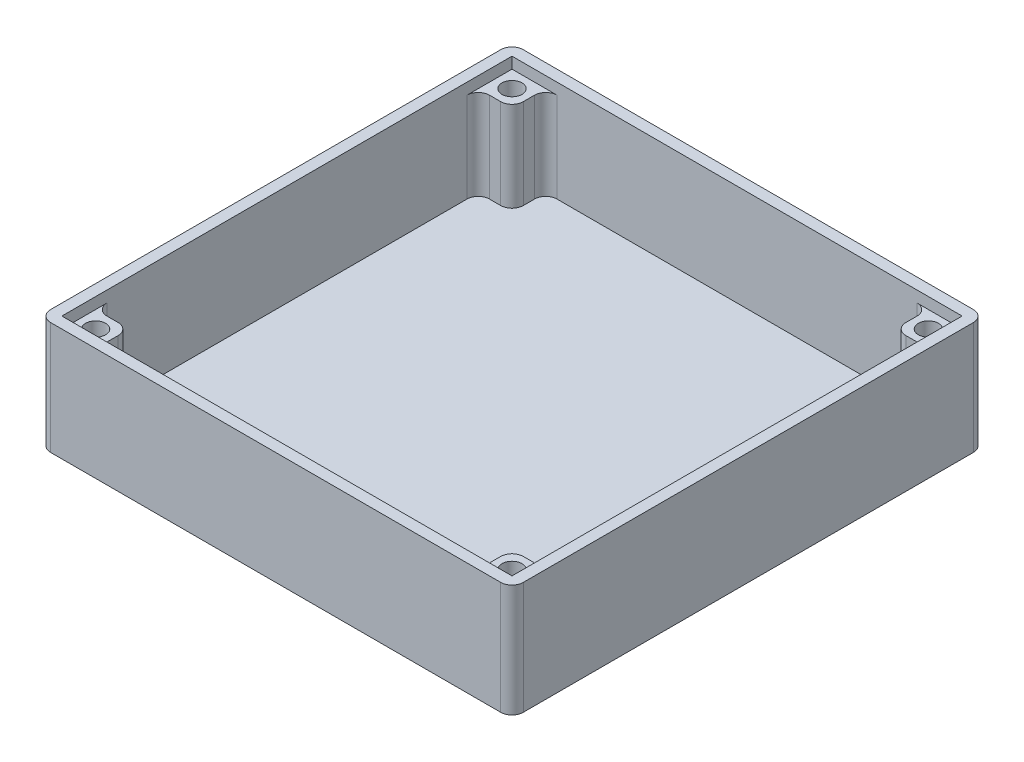
SolidWorks part; units mm, degrees
ref_plane "Front Plane" through (0, 0, 0) normal (0, 0, 1) x (1, 0, 0)
ref_plane "Top Plane" through (0, 0, 0) normal (0, 1, 0) x (1, 0, 0)
ref_plane "Right Plane" through (0, 0, 0) normal (1, 0, 0) x (0, 0, -1)
sketch "Sketch1" plane through (0, 0, 0) normal (0, 1, 0) x (1, 0, 0)
  line L0 (0, 0) -> (0, 50.8)
  line L1 (0, 50.8) -> (50.8, 50.8)
  line L2 (50.8, 50.8) -> (50.8, 0)
  line L3 (50.8, 0) -> (0, 0)
  line L4 (29.845, 40.64) -> (28.575, 40.64)
  line L5 (30.48, 43.18) -> (30.48, 38.1)
  line L6 (30.48, 38.1) -> (27.94, 38.1)
  line L7 (27.94, 38.1) -> (27.94, 43.18)
  line L8 (27.94, 43.18) -> (30.48, 43.18)
  line L9 (28.3382, 37.639) -> (28.245, 37.7322)
  line L10 (28.245, 37.7322) -> (28.0586, 37.7322)
  line L11 (28.0586, 37.7322) -> (27.9654, 37.639)
  line L12 (27.9654, 37.639) -> (27.9654, 37.2661)
  line L13 (27.9654, 37.2661) -> (28.0586, 37.1729)
  line L14 (28.0586, 37.1729) -> (28.245, 37.1729)
  line L15 (28.245, 37.1729) -> (28.3382, 37.2661)
  line L16 (28.5267, 37.5457) -> (28.7131, 37.7322)
  line L17 (28.7131, 37.7322) -> (28.7131, 37.1729)
  line L18 (28.5267, 37.1729) -> (28.8996, 37.1729)
  line L19 (28.2829, 43.8957) -> (28.4693, 44.0822)
  line L20 (28.4693, 44.0822) -> (28.4693, 43.5229)
  line L21 (28.2829, 43.5229) -> (28.6557, 43.5229)
  line L22 (28.8442, 43.6161) -> (28.8442, 43.989)
  line L23 (28.8442, 43.989) -> (28.9374, 44.0822)
  line L24 (28.9374, 44.0822) -> (29.1238, 44.0822)
  line L25 (29.1238, 44.0822) -> (29.2171, 43.989)
  line L26 (29.2171, 43.989) -> (29.2171, 43.6161)
  line L27 (29.2171, 43.6161) -> (29.1238, 43.5229)
  line L28 (29.1238, 43.5229) -> (28.9374, 43.5229)
  line L29 (28.9374, 43.5229) -> (28.8442, 43.6161)
  line L30 (28.8442, 43.6161) -> (29.2171, 43.989)
  line L31 (29.4055, 43.8957) -> (29.4055, 43.6161)
  line L32 (29.4055, 43.6161) -> (29.4987, 43.5229)
  line L33 (29.4987, 43.5229) -> (29.7784, 43.5229)
  line L34 (29.7784, 43.5229) -> (29.7784, 43.8957)
  line L35 (29.9668, 43.5229) -> (29.9668, 44.0822)
  line L36 (29.9668, 44.0822) -> (30.3397, 44.0822)
  line L37 (29.9668, 43.8025) -> (30.1533, 43.8025)
  line L38 (24.765, 40.64) -> (26.035, 40.64)
  line L39 (24.13, 38.1) -> (24.13, 43.18)
  line L40 (24.13, 43.18) -> (26.67, 43.18)
  line L41 (26.67, 43.18) -> (26.67, 38.1)
  line L42 (26.67, 38.1) -> (24.13, 38.1)
  line L43 (24.6756, 37.6644) -> (24.5824, 37.7576)
  line L44 (24.5824, 37.7576) -> (24.396, 37.7576)
  line L45 (24.396, 37.7576) -> (24.3028, 37.6644)
  line L46 (24.3028, 37.6644) -> (24.3028, 37.2915)
  line L47 (24.3028, 37.2915) -> (24.396, 37.1983)
  line L48 (24.396, 37.1983) -> (24.5824, 37.1983)
  line L49 (24.5824, 37.1983) -> (24.6756, 37.2915)
  line L50 (25.2369, 37.1983) -> (24.8641, 37.1983)
  line L51 (24.8641, 37.1983) -> (25.2369, 37.5711)
  line L52 (25.2369, 37.5711) -> (25.2369, 37.6644)
  line L53 (25.2369, 37.6644) -> (25.1437, 37.7576)
  line L54 (25.1437, 37.7576) -> (24.9573, 37.7576)
  line L55 (24.9573, 37.7576) -> (24.8641, 37.6644)
  line L56 (24.1326, 43.9211) -> (24.3191, 44.1076)
  line L57 (24.3191, 44.1076) -> (24.3191, 43.5483)
  line L58 (24.1326, 43.5483) -> (24.5055, 43.5483)
  line L59 (24.694, 43.6415) -> (24.694, 44.0144)
  line L60 (24.694, 44.0144) -> (24.7872, 44.1076)
  line L61 (24.7872, 44.1076) -> (24.9736, 44.1076)
  line L62 (24.9736, 44.1076) -> (25.0668, 44.0144)
  line L63 (25.0668, 44.0144) -> (25.0668, 43.6415)
  line L64 (25.0668, 43.6415) -> (24.9736, 43.5483)
  line L65 (24.9736, 43.5483) -> (24.7872, 43.5483)
  line L66 (24.7872, 43.5483) -> (24.694, 43.6415)
  line L67 (24.694, 43.6415) -> (25.0668, 44.0144)
  line L68 (25.2553, 43.9211) -> (25.2553, 43.6415)
  line L69 (25.2553, 43.6415) -> (25.3485, 43.5483)
  line L70 (25.3485, 43.5483) -> (25.6281, 43.5483)
  line L71 (25.6281, 43.5483) -> (25.6281, 43.9211)
  line L72 (25.8166, 43.5483) -> (25.8166, 44.1076)
  line L73 (25.8166, 44.1076) -> (26.1894, 44.1076)
  line L74 (25.8166, 43.8279) -> (26.003, 43.8279)
  line L75 (15.748, 34.29) -> (19.812, 34.29)
  line L76 (15.748, 34.29) -> (15.748, 31.75)
  line L77 (19.812, 31.75) -> (15.748, 31.75)
  line L78 (19.812, 31.75) -> (19.812, 34.29)
  line L79 (12.7, 33.02) -> (13.716, 33.02)
  line L80 (22.86, 33.02) -> (21.844, 33.02)
  line L81 (18.415, 33.02) -> (17.78, 33.02)
  line L82 (16.764, 32.385) -> (16.764, 33.655)
  line L83 (16.764, 33.655) -> (17.78, 33.02)
  line L84 (17.78, 33.02) -> (16.256, 33.02)
  line L85 (17.78, 33.02) -> (16.764, 32.385)
  line L86 (17.78, 32.385) -> (17.78, 33.02)
  line L87 (17.78, 33.02) -> (17.78, 33.655)
  line L88 (12.8591, 35.3702) -> (13.2404, 35.7515)
  line L89 (13.2404, 35.7515) -> (13.2404, 34.6075)
  line L90 (12.8591, 34.6075) -> (13.6217, 34.6075)
  line L91 (14.0285, 34.6075) -> (14.0285, 35.7515)
  line L92 (14.0285, 35.7515) -> (14.7912, 34.6075)
  line L93 (14.7912, 34.6075) -> (14.7912, 35.7515)
  line L94 (15.7699, 34.6075) -> (15.7699, 35.7515)
  line L95 (15.7699, 35.7515) -> (15.1979, 35.1795)
  line L96 (15.1979, 35.1795) -> (15.9605, 35.1795)
  line L97 (16.3673, 34.7982) -> (16.3673, 35.5608)
  line L98 (16.3673, 35.5608) -> (16.558, 35.7515)
  line L99 (16.558, 35.7515) -> (16.9393, 35.7515)
  line L100 (16.9393, 35.7515) -> (17.1299, 35.5608)
  line L101 (17.1299, 35.5608) -> (17.1299, 34.7982)
  line L102 (17.1299, 34.7982) -> (16.9393, 34.6075)
  line L103 (16.9393, 34.6075) -> (16.558, 34.6075)
  line L104 (16.558, 34.6075) -> (16.3673, 34.7982)
  line L105 (16.3673, 34.7982) -> (17.1299, 35.5608)
  line L106 (17.5367, 34.7982) -> (17.5367, 35.5608)
  line L107 (17.5367, 35.5608) -> (17.7273, 35.7515)
  line L108 (17.7273, 35.7515) -> (18.1087, 35.7515)
  line L109 (18.1087, 35.7515) -> (18.2993, 35.5608)
  line L110 (18.2993, 35.5608) -> (18.2993, 34.7982)
  line L111 (18.2993, 34.7982) -> (18.1087, 34.6075)
  line L112 (18.1087, 34.6075) -> (17.7273, 34.6075)
  line L113 (17.7273, 34.6075) -> (17.5367, 34.7982)
  line L114 (17.5367, 34.7982) -> (18.2993, 35.5608)
  line L115 (18.7061, 35.3702) -> (19.0874, 35.7515)
  line L116 (19.0874, 35.7515) -> (19.0874, 34.6075)
  line L117 (18.7061, 34.6075) -> (19.4687, 34.6075)
  line L118 (4.39, 39.64) -> (6.49, 39.64)
  line L119 (13.39, 50.34) -> (13.39, 53.24)
  line L120 (4.39, 53.24) -> (4.39, 50.34)
  line L121 (4.39, 53.24) -> (13.39, 53.24)
  line L122 (4.39, 50.34) -> (4.39, 45.04)
  line L123 (4.39, 39.64) -> (4.39, 40.34)
  line L124 (13.39, 50.34) -> (13.39, 39.64)
  line L125 (13.39, 39.64) -> (11.29, 39.64)
  line L126 (13.39, 50.34) -> (4.39, 50.34)
  line L127 (11.5901, 47.9299) -> (11.6536, 47.8663)
  line L128 (11.6536, 47.8663) -> (11.7172, 47.8663)
  line L129 (11.7172, 47.8663) -> (11.7807, 47.9299)
  line L130 (11.7807, 47.9299) -> (11.7807, 48.2476)
  line L131 (11.7172, 48.2476) -> (11.8443, 48.2476)
  line L132 (11.9643, 47.8663) -> (11.9643, 48.2476)
  line L133 (11.9643, 48.2476) -> (12.1549, 48.2476)
  line L134 (12.1549, 48.2476) -> (12.2185, 48.1841)
  line L135 (12.2185, 48.1841) -> (12.2185, 48.057)
  line L136 (12.2185, 48.057) -> (12.1549, 47.9934)
  line L137 (12.1549, 47.9934) -> (11.9643, 47.9934)
  line L138 (12.3385, 48.1205) -> (12.4656, 48.2476)
  line L139 (12.4656, 48.2476) -> (12.4656, 47.8663)
  line L140 (12.3385, 47.8663) -> (12.5927, 47.8663)
  line L141 (7.848, 49.1363) -> (7.848, 49.5176)
  line L142 (7.848, 49.5176) -> (8.0387, 49.5176)
  line L143 (8.0387, 49.5176) -> (8.1022, 49.4541)
  line L144 (8.1022, 49.4541) -> (8.1022, 49.327)
  line L145 (8.1022, 49.327) -> (8.0387, 49.2634)
  line L146 (8.0387, 49.2634) -> (7.848, 49.2634)
  line L147 (8.4129, 49.5176) -> (8.2858, 49.5176)
  line L148 (8.2858, 49.5176) -> (8.2222, 49.4541)
  line L149 (8.2222, 49.4541) -> (8.2222, 49.1999)
  line L150 (8.2222, 49.1999) -> (8.2858, 49.1363)
  line L151 (8.2858, 49.1363) -> (8.4129, 49.1363)
  line L152 (8.4129, 49.1363) -> (8.4764, 49.1999)
  line L153 (8.4764, 49.1999) -> (8.4764, 49.4541)
  line L154 (8.4764, 49.4541) -> (8.4129, 49.5176)
  line L155 (8.5964, 49.5176) -> (8.5964, 49.1363)
  line L156 (8.5964, 49.1363) -> (8.7235, 49.2634)
  line L157 (8.7235, 49.2634) -> (8.8506, 49.1363)
  line L158 (8.8506, 49.1363) -> (8.8506, 49.5176)
  line L159 (9.2248, 49.5176) -> (8.9706, 49.5176)
  line L160 (8.9706, 49.5176) -> (8.9706, 49.1363)
  line L161 (8.9706, 49.1363) -> (9.2248, 49.1363)
  line L162 (8.9706, 49.327) -> (9.0977, 49.327)
  line L163 (9.3448, 49.1363) -> (9.3448, 49.5176)
  line L164 (9.3448, 49.5176) -> (9.5355, 49.5176)
  line L165 (9.5355, 49.5176) -> (9.599, 49.4541)
  line L166 (9.599, 49.4541) -> (9.599, 49.327)
  line L167 (9.599, 49.327) -> (9.5355, 49.2634)
  line L168 (9.5355, 49.2634) -> (9.3448, 49.2634)
  line L169 (9.4719, 49.2634) -> (9.599, 49.1363)
  line L170 (9.719, 49.0727) -> (9.9733, 49.0727)
  line L171 (10.0932, 49.1999) -> (10.1568, 49.1363)
  line L172 (10.1568, 49.1363) -> (10.2204, 49.1363)
  line L173 (10.2204, 49.1363) -> (10.2839, 49.1999)
  line L174 (10.2839, 49.1999) -> (10.2839, 49.5176)
  line L175 (10.2204, 49.5176) -> (10.3475, 49.5176)
  line L176 (10.4674, 49.1363) -> (10.4674, 49.3905)
  line L177 (10.4674, 49.3905) -> (10.5945, 49.5176)
  line L178 (10.5945, 49.5176) -> (10.7217, 49.3905)
  line L179 (10.7217, 49.3905) -> (10.7217, 49.1363)
  line L180 (10.4674, 49.327) -> (10.7217, 49.327)
  line L181 (11.0959, 49.4541) -> (11.0323, 49.5176)
  line L182 (11.0323, 49.5176) -> (10.9052, 49.5176)
  line L183 (10.9052, 49.5176) -> (10.8417, 49.4541)
  line L184 (10.8417, 49.4541) -> (10.8417, 49.1999)
  line L185 (10.8417, 49.1999) -> (10.9052, 49.1363)
  line L186 (10.9052, 49.1363) -> (11.0323, 49.1363)
  line L187 (11.0323, 49.1363) -> (11.0959, 49.1999)
  line L188 (11.2159, 49.5176) -> (11.2159, 49.1363)
  line L189 (11.2159, 49.2634) -> (11.4701, 49.5176)
  line L190 (11.2794, 49.327) -> (11.4701, 49.1363)
  line L191 (11.5901, 49.1363) -> (11.5901, 49.5176)
  line L192 (11.5901, 49.5176) -> (11.7807, 49.5176)
  line L193 (11.7807, 49.5176) -> (11.8443, 49.4541)
  line L194 (11.8443, 49.4541) -> (11.8443, 49.327)
  line L195 (11.8443, 49.327) -> (11.7807, 49.2634)
  line L196 (11.7807, 49.2634) -> (11.5901, 49.2634)
  line L197 (12.0914, 49.1363) -> (12.0914, 49.5176)
  line L198 (11.9643, 49.5176) -> (12.2185, 49.5176)
  line L199 (12.3385, 49.1363) -> (12.3385, 49.5176)
  line L200 (12.3385, 49.327) -> (12.5927, 49.327)
  line L201 (12.5927, 49.5176) -> (12.5927, 49.1363)
  line L202 (10.795, 1.27) -> (24.765, 1.27)
  line L203 (24.765, 1.27) -> (24.765, 35.56)
  line L204 (24.765, 35.56) -> (10.795, 35.56)
  line L205 (10.795, 35.56) -> (10.795, 1.27)
  line L206 (14.1986, 3.8354) -> (13.6393, 3.8354)
  line L207 (13.6393, 3.8354) -> (13.6393, 4.115)
  line L208 (13.6393, 4.115) -> (13.7325, 4.2082)
  line L209 (13.7325, 4.2082) -> (13.919, 4.2082)
  line L210 (13.919, 4.2082) -> (14.0122, 4.115)
  line L211 (14.0122, 4.115) -> (14.0122, 3.8354)
  line L212 (14.0122, 4.0218) -> (14.1986, 4.2082)
  line L213 (13.6393, 4.3967) -> (14.1986, 4.7696)
  line L214 (13.6393, 4.7696) -> (14.1986, 4.3967)
  line L215 (16.7386, 4.0218) -> (16.1793, 4.0218)
  line L216 (16.1793, 3.8354) -> (16.1793, 4.2082)
  line L217 (16.1793, 4.3967) -> (16.7386, 4.7696)
  line L218 (16.1793, 4.7696) -> (16.7386, 4.3967)
  line L219 (18.8125, 4.2082) -> (18.7193, 4.115)
  line L220 (18.7193, 4.115) -> (18.7193, 3.9286)
  line L221 (18.7193, 3.9286) -> (18.8125, 3.8354)
  line L222 (18.8125, 3.8354) -> (19.1854, 3.8354)
  line L223 (19.1854, 3.8354) -> (19.2786, 3.9286)
  line L224 (19.2786, 3.9286) -> (19.2786, 4.115)
  line L225 (19.2786, 4.115) -> (19.1854, 4.2082)
  line L226 (19.1854, 4.2082) -> (18.999, 4.2082)
  line L227 (18.999, 4.2082) -> (18.999, 4.0218)
  line L228 (19.2786, 4.3967) -> (18.7193, 4.3967)
  line L229 (18.7193, 4.3967) -> (19.2786, 4.7696)
  line L230 (19.2786, 4.7696) -> (18.7193, 4.7696)
  line L231 (18.7193, 4.958) -> (19.2786, 4.958)
  line L232 (19.2786, 4.958) -> (19.2786, 5.2377)
  line L233 (19.2786, 5.2377) -> (19.1854, 5.3309)
  line L234 (19.1854, 5.3309) -> (18.8125, 5.3309)
  line L235 (18.8125, 5.3309) -> (18.7193, 5.2377)
  line L236 (18.7193, 5.2377) -> (18.7193, 4.958)
  line L237 (21.2593, 3.8354) -> (21.6322, 3.8354)
  line L238 (21.6322, 3.8354) -> (21.8186, 4.0218)
  line L239 (21.8186, 4.0218) -> (21.6322, 4.2082)
  line L240 (21.6322, 4.2082) -> (21.2593, 4.2082)
  line L241 (21.3525, 4.7696) -> (21.2593, 4.6763)
  line L242 (21.2593, 4.6763) -> (21.2593, 4.4899)
  line L243 (21.2593, 4.4899) -> (21.3525, 4.3967)
  line L244 (21.3525, 4.3967) -> (21.7254, 4.3967)
  line L245 (21.7254, 4.3967) -> (21.8186, 4.4899)
  line L246 (21.8186, 4.4899) -> (21.8186, 4.6763)
  line L247 (21.8186, 4.6763) -> (21.7254, 4.7696)
  line L248 (21.3525, 5.3309) -> (21.2593, 5.2377)
  line L249 (21.2593, 5.2377) -> (21.2593, 5.0512)
  line L250 (21.2593, 5.0512) -> (21.3525, 4.958)
  line L251 (21.3525, 4.958) -> (21.7254, 4.958)
  line L252 (21.7254, 4.958) -> (21.8186, 5.0512)
  line L253 (21.8186, 5.0512) -> (21.8186, 5.2377)
  line L254 (21.8186, 5.2377) -> (21.7254, 5.3309)
  line L255 (10.0752, 1.3335) -> (10.2235, 1.4818)
  line L256 (10.2235, 1.4818) -> (10.2235, 1.6301)
  line L257 (10.2235, 1.6301) -> (10.0752, 1.7784)
  line L258 (10.0752, 1.7784) -> (9.3337, 1.7784)
  line L259 (9.3337, 1.6301) -> (9.3337, 1.9267)
  line L260 (10.3718, 2.269) -> (10.3718, 2.8622)
  line L261 (10.2235, 3.2045) -> (9.3337, 3.2045)
  line L262 (9.3337, 3.2045) -> (9.3337, 3.6494)
  line L263 (9.3337, 3.6494) -> (9.482, 3.7977)
  line L264 (9.482, 3.7977) -> (9.6303, 3.7977)
  line L265 (9.6303, 3.7977) -> (9.7786, 3.6494)
  line L266 (9.7786, 3.6494) -> (9.9269, 3.7977)
  line L267 (9.9269, 3.7977) -> (10.0752, 3.7977)
  line L268 (10.0752, 3.7977) -> (10.2235, 3.6494)
  line L269 (10.2235, 3.6494) -> (10.2235, 3.2045)
  line L270 (9.7786, 3.2045) -> (9.7786, 3.6494)
  line L271 (10.2235, 4.4366) -> (9.3337, 4.4366)
  line L272 (9.3337, 4.14) -> (9.3337, 4.7332)
  line L273 (10.3718, 5.0756) -> (10.3718, 5.6687)
  line L274 (10.2235, 6.0111) -> (9.3337, 6.0111)
  line L275 (9.3337, 6.0111) -> (9.3337, 6.456)
  line L276 (9.3337, 6.456) -> (9.482, 6.6043)
  line L277 (9.482, 6.6043) -> (9.6303, 6.6043)
  line L278 (9.6303, 6.6043) -> (9.7786, 6.456)
  line L279 (9.7786, 6.456) -> (9.9269, 6.6043)
  line L280 (9.9269, 6.6043) -> (10.0752, 6.6043)
  line L281 (10.0752, 6.6043) -> (10.2235, 6.456)
  line L282 (10.2235, 6.456) -> (10.2235, 6.0111)
  line L283 (9.7786, 6.0111) -> (9.7786, 6.456)
  line L284 (9.3337, 7.3915) -> (9.3337, 7.0949)
  line L285 (9.3337, 7.0949) -> (9.482, 6.9466)
  line L286 (9.482, 6.9466) -> (10.0752, 6.9466)
  line L287 (10.0752, 6.9466) -> (10.2235, 7.0949)
  line L288 (10.2235, 7.0949) -> (10.2235, 7.3915)
  line L289 (10.2235, 7.3915) -> (10.0752, 7.5398)
  line L290 (10.0752, 7.5398) -> (9.482, 7.5398)
  line L291 (9.482, 7.5398) -> (9.3337, 7.3915)
  line L292 (10.2235, 7.8821) -> (9.6303, 7.8821)
  line L293 (9.6303, 7.8821) -> (9.3337, 8.1787)
  line L294 (9.3337, 8.1787) -> (9.6303, 8.4753)
  line L295 (9.6303, 8.4753) -> (10.2235, 8.4753)
  line L296 (9.7786, 7.8821) -> (9.7786, 8.4753)
  line L297 (10.2235, 8.8177) -> (9.3337, 8.8177)
  line L298 (9.3337, 8.8177) -> (9.3337, 9.2625)
  line L299 (9.3337, 9.2625) -> (9.482, 9.4108)
  line L300 (9.482, 9.4108) -> (9.7786, 9.4108)
  line L301 (9.7786, 9.4108) -> (9.9269, 9.2625)
  line L302 (9.9269, 9.2625) -> (9.9269, 8.8177)
  line L303 (9.9269, 9.1142) -> (10.2235, 9.4108)
  line L304 (9.3337, 9.7532) -> (10.2235, 9.7532)
  line L305 (10.2235, 9.7532) -> (10.2235, 10.198)
  line L306 (10.2235, 10.198) -> (10.0752, 10.3463)
  line L307 (10.0752, 10.3463) -> (9.482, 10.3463)
  line L308 (9.482, 10.3463) -> (9.3337, 10.198)
  line L309 (9.3337, 10.198) -> (9.3337, 9.7532)
  line L310 (10.3718, 10.6887) -> (10.3718, 11.2819)
  line L311 (9.6303, 11.6242) -> (9.3337, 11.9208)
  line L312 (9.3337, 11.9208) -> (10.2235, 11.9208)
  line L313 (10.2235, 11.6242) -> (10.2235, 12.2174)
  line L314 (3.81, 35.8648) -> (1.27, 35.8648)
  line L315 (0.9515, 36.2585) -> (2.0955, 36.2585)
  line L316 (2.0955, 36.2585) -> (2.0955, 37.0212)
  line L317 (0.9515, 38.1906) -> (0.9515, 37.4279)
  line L318 (0.9515, 37.4279) -> (2.0955, 37.4279)
  line L319 (2.0955, 37.4279) -> (2.0955, 38.1906)
  line L320 (1.5235, 37.4279) -> (1.5235, 37.8092)
  line L321 (0.9515, 38.5973) -> (2.0955, 38.5973)
  line L322 (2.0955, 38.5973) -> (2.0955, 39.1693)
  line L323 (2.0955, 39.1693) -> (1.9048, 39.3599)
  line L324 (1.9048, 39.3599) -> (1.1422, 39.3599)
  line L325 (1.1422, 39.3599) -> (0.9515, 39.1693)
  line L326 (0.9515, 39.1693) -> (0.9515, 38.5973)
  line L327 (1.3328, 39.7667) -> (0.9515, 40.148)
  line L328 (0.9515, 40.148) -> (2.0955, 40.148)
  line L329 (2.0955, 39.7667) -> (2.0955, 40.5293)
  line L330 (2.6768, 32.6898) -> (2.4032, 32.6898)
  line L331 (2.4032, 32.6898) -> (2.2098, 32.8832)
  line L332 (2.2098, 32.8832) -> (2.2098, 33.1568)
  line L333 (2.2098, 33.1568) -> (2.4032, 33.3502)
  line L334 (2.4032, 33.3502) -> (2.6768, 33.3502)
  line L335 (2.6768, 33.3502) -> (2.8702, 33.1568)
  line L336 (2.8702, 33.1568) -> (2.8702, 32.8832)
  line L337 (2.8702, 32.8832) -> (2.6768, 32.6898)
  line L338 (2.6768, 32.6898) -> (2.4032, 32.6898)
  line L339 (2.6768, 32.6898) -> (2.4032, 32.6898)
  line L340 (2.4032, 32.6898) -> (2.2098, 32.8832)
  line L341 (2.2098, 32.8832) -> (2.2098, 33.1568)
  line L342 (2.2098, 33.1568) -> (2.4032, 33.3502)
  line L343 (2.4032, 33.3502) -> (2.6768, 33.3502)
  line L344 (2.6768, 33.3502) -> (2.8702, 33.1568)
  line L345 (2.8702, 33.1568) -> (2.8702, 32.8832)
  line L346 (2.8702, 32.8832) -> (2.6768, 32.6898)
  line L347 (2.6768, 32.6898) -> (2.4032, 32.6898)
  line L348 (2.6768, 35.2298) -> (2.4032, 35.2298)
  line L349 (2.4032, 35.2298) -> (2.2098, 35.4232)
  line L350 (2.2098, 35.4232) -> (2.2098, 35.6968)
  line L351 (2.2098, 35.6968) -> (2.4032, 35.8902)
  line L352 (2.4032, 35.8902) -> (2.6768, 35.8902)
  line L353 (2.6768, 35.8902) -> (2.8702, 35.6968)
  line L354 (2.8702, 35.6968) -> (2.8702, 35.4232)
  line L355 (2.8702, 35.4232) -> (2.6768, 35.2298)
  line L356 (2.6768, 35.2298) -> (2.4032, 35.2298)
  line L357 (2.6768, 35.2298) -> (2.4032, 35.2298)
  line L358 (2.4032, 35.2298) -> (2.2098, 35.4232)
  line L359 (2.2098, 35.4232) -> (2.2098, 35.6968)
  line L360 (2.2098, 35.6968) -> (2.4032, 35.8902)
  line L361 (2.4032, 35.8902) -> (2.6768, 35.8902)
  line L362 (2.6768, 35.8902) -> (2.8702, 35.6968)
  line L363 (2.8702, 35.6968) -> (2.8702, 35.4232)
  line L364 (2.8702, 35.4232) -> (2.6768, 35.2298)
  line L365 (2.6768, 35.2298) -> (2.4032, 35.2298)
  line L366 (10.16, 36.83) -> (10.16, 31.75)
  line L367 (10.16, 31.75) -> (5.08, 31.75)
  line L368 (5.08, 31.75) -> (5.08, 36.83)
  line L369 (5.08, 36.83) -> (10.16, 36.83)
  line L370 (8.9275, 32.8596) -> (8.9275, 32.6139)
  line L371 (8.9275, 32.6139) -> (9.0504, 32.491)
  line L372 (9.0504, 32.491) -> (9.5418, 32.491)
  line L373 (9.5418, 32.491) -> (9.6647, 32.6139)
  line L374 (9.6647, 32.6139) -> (9.6647, 32.8596)
  line L375 (9.6647, 32.8596) -> (9.5418, 32.9825)
  line L376 (9.5418, 32.9825) -> (9.0504, 32.9825)
  line L377 (9.0504, 32.9825) -> (8.9275, 32.8596)
  line L378 (9.6647, 33.2394) -> (8.9275, 33.2394)
  line L379 (8.9275, 33.2394) -> (9.6647, 33.7309)
  line L380 (9.6647, 33.7309) -> (8.9275, 33.7309)
  line L381 (8.9275, 34.3565) -> (8.9275, 34.1107)
  line L382 (8.9275, 34.1107) -> (9.0504, 33.9878)
  line L383 (9.0504, 33.9878) -> (9.5418, 33.9878)
  line L384 (9.5418, 33.9878) -> (9.6647, 34.1107)
  line L385 (9.6647, 34.1107) -> (9.6647, 34.3565)
  line L386 (9.6647, 34.3565) -> (9.5418, 34.4793)
  line L387 (9.5418, 34.4793) -> (9.0504, 34.4793)
  line L388 (9.0504, 34.4793) -> (8.9275, 34.3565)
  line L389 (9.6647, 34.7363) -> (8.9275, 34.7363)
  line L390 (8.9275, 34.7363) -> (8.9275, 35.2277)
  line L391 (9.2961, 34.7363) -> (9.2961, 34.982)
  line L392 (9.6647, 35.4847) -> (8.9275, 35.4847)
  line L393 (8.9275, 35.4847) -> (8.9275, 35.9762)
  line L394 (9.2961, 35.4847) -> (9.2961, 35.7304)
  line L395 (5.7525, 31.7426) -> (6.4897, 31.7426)
  line L396 (6.4897, 31.7426) -> (6.4897, 32.1112)
  line L397 (6.4897, 32.1112) -> (6.3668, 32.2341)
  line L398 (6.3668, 32.2341) -> (5.8754, 32.2341)
  line L399 (5.8754, 32.2341) -> (5.7525, 32.1112)
  line L400 (5.7525, 32.1112) -> (5.7525, 31.7426)
  line L401 (5.8754, 32.9825) -> (5.7525, 32.8596)
  line L402 (5.7525, 32.8596) -> (5.7525, 32.6139)
  line L403 (5.7525, 32.6139) -> (5.8754, 32.491)
  line L404 (5.8754, 32.491) -> (5.9982, 32.491)
  line L405 (5.9982, 32.491) -> (6.1211, 32.6139)
  line L406 (6.1211, 32.6139) -> (6.1211, 32.8596)
  line L407 (6.1211, 32.8596) -> (6.244, 32.9825)
  line L408 (6.244, 32.9825) -> (6.3668, 32.9825)
  line L409 (6.3668, 32.9825) -> (6.4897, 32.8596)
  line L410 (6.4897, 32.8596) -> (6.4897, 32.6139)
  line L411 (6.4897, 32.6139) -> (6.3668, 32.491)
  line L412 (6.1211, 33.2394) -> (6.1211, 33.7309)
  line L413 (6.4897, 34.4793) -> (6.4897, 33.9878)
  line L414 (6.4897, 33.9878) -> (5.9982, 34.4793)
  line L415 (5.9982, 34.4793) -> (5.8754, 34.4793)
  line L416 (5.8754, 34.4793) -> (5.7525, 34.3565)
  line L417 (5.7525, 34.3565) -> (5.7525, 34.1107)
  line L418 (5.7525, 34.1107) -> (5.8754, 33.9878)
  line L419 (6.4897, 35.2277) -> (6.4897, 34.7363)
  line L420 (6.4897, 34.7363) -> (5.9982, 35.2277)
  line L421 (5.9982, 35.2277) -> (5.8754, 35.2277)
  line L422 (5.8754, 35.2277) -> (5.7525, 35.1049)
  line L423 (5.7525, 35.1049) -> (5.7525, 34.8591)
  line L424 (5.7525, 34.8591) -> (5.8754, 34.7363)
  line L425 (5.8754, 35.4847) -> (5.7525, 35.6075)
  line L426 (5.7525, 35.6075) -> (5.7525, 35.8533)
  line L427 (5.7525, 35.8533) -> (5.8754, 35.9762)
  line L428 (5.8754, 35.9762) -> (5.9982, 35.9762)
  line L429 (5.9982, 35.9762) -> (6.1211, 35.8533)
  line L430 (6.1211, 35.8533) -> (6.244, 35.9762)
  line L431 (6.244, 35.9762) -> (6.3668, 35.9762)
  line L432 (6.3668, 35.9762) -> (6.4897, 35.8533)
  line L433 (6.4897, 35.8533) -> (6.4897, 35.6075)
  line L434 (6.4897, 35.6075) -> (6.3668, 35.4847)
  line L435 (6.3668, 35.4847) -> (6.244, 35.4847)
  line L436 (6.244, 35.4847) -> (6.1211, 35.6075)
  line L437 (6.1211, 35.6075) -> (5.9982, 35.4847)
  line L438 (5.9982, 35.4847) -> (5.8754, 35.4847)
  line L439 (6.1211, 35.6075) -> (6.1211, 35.8533)
  line L440 (15.24, 21.082) -> (20.32, 21.082)
  line L441 (20.32, 21.082) -> (20.32, 20.32)
  line L442 (20.32, 20.32) -> (20.32, 19.558)
  line L443 (20.32, 19.558) -> (15.24, 19.558)
  line L444 (15.24, 19.558) -> (15.24, 20.32)
  line L445 (15.24, 20.32) -> (15.24, 21.082)
  line L446 (20.32, 20.32) -> (20.574, 20.32)
  line L447 (15.24, 20.32) -> (14.986, 20.32)
  line L448 (15.2527, 21.6027) -> (15.2527, 21.984)
  line L449 (15.2527, 21.984) -> (15.4434, 21.984)
  line L450 (15.4434, 21.984) -> (15.5069, 21.9205)
  line L451 (15.5069, 21.9205) -> (15.5069, 21.7934)
  line L452 (15.5069, 21.7934) -> (15.4434, 21.7298)
  line L453 (15.4434, 21.7298) -> (15.2527, 21.7298)
  line L454 (15.3798, 21.7298) -> (15.5069, 21.6027)
  line L455 (15.6269, 21.8569) -> (15.754, 21.984)
  line L456 (15.754, 21.984) -> (15.754, 21.6027)
  line L457 (15.6269, 21.6027) -> (15.8811, 21.6027)
  line L458 (15.8242, 20.5914) -> (16.1123, 20.8795)
  line L459 (16.1123, 20.8795) -> (16.1123, 20.0152)
  line L460 (15.8242, 20.0152) -> (16.4004, 20.0152)
  line L461 (16.7597, 20.1593) -> (16.7597, 20.7355)
  line L462 (16.7597, 20.7355) -> (16.9038, 20.8795)
  line L463 (16.9038, 20.8795) -> (17.1919, 20.8795)
  line L464 (17.1919, 20.8795) -> (17.3359, 20.7355)
  line L465 (17.3359, 20.7355) -> (17.3359, 20.1593)
  line L466 (17.3359, 20.1593) -> (17.1919, 20.0152)
  line L467 (17.1919, 20.0152) -> (16.9038, 20.0152)
  line L468 (16.9038, 20.0152) -> (16.7597, 20.1593)
  line L469 (16.7597, 20.1593) -> (17.3359, 20.7355)
  line L470 (17.6952, 20.8795) -> (17.6952, 20.0152)
  line L471 (17.6952, 20.3033) -> (18.2715, 20.8795)
  line L472 (17.8393, 20.4474) -> (18.2715, 20.0152)
  line L473 (15.24, 18.542) -> (20.32, 18.542)
  line L474 (20.32, 18.542) -> (20.32, 17.78)
  line L475 (20.32, 17.78) -> (20.32, 17.018)
  line L476 (20.32, 17.018) -> (15.24, 17.018)
  line L477 (15.24, 17.018) -> (15.24, 17.78)
  line L478 (15.24, 17.78) -> (15.24, 18.542)
  line L479 (20.32, 17.78) -> (20.574, 17.78)
  line L480 (15.24, 17.78) -> (14.986, 17.78)
  line L481 (15.2527, 19.0627) -> (15.2527, 19.444)
  line L482 (15.2527, 19.444) -> (15.4434, 19.444)
  line L483 (15.4434, 19.444) -> (15.5069, 19.3805)
  line L484 (15.5069, 19.3805) -> (15.5069, 19.2534)
  line L485 (15.5069, 19.2534) -> (15.4434, 19.1898)
  line L486 (15.4434, 19.1898) -> (15.2527, 19.1898)
  line L487 (15.3798, 19.1898) -> (15.5069, 19.0627)
  line L488 (15.8811, 19.0627) -> (15.6269, 19.0627)
  line L489 (15.6269, 19.0627) -> (15.8811, 19.3169)
  line L490 (15.8811, 19.3169) -> (15.8811, 19.3805)
  line L491 (15.8811, 19.3805) -> (15.8176, 19.444)
  line L492 (15.8176, 19.444) -> (15.6905, 19.444)
  line L493 (15.6905, 19.444) -> (15.6269, 19.3805)
  line L494 (15.8242, 18.0514) -> (16.1123, 18.3395)
  line L495 (16.1123, 18.3395) -> (16.1123, 17.4752)
  line L496 (15.8242, 17.4752) -> (16.4004, 17.4752)
  line L497 (16.7597, 17.6193) -> (16.7597, 18.1955)
  line L498 (16.7597, 18.1955) -> (16.9038, 18.3395)
  line L499 (16.9038, 18.3395) -> (17.1919, 18.3395)
  line L500 (17.1919, 18.3395) -> (17.3359, 18.1955)
  line L501 (17.3359, 18.1955) -> (17.3359, 17.6193)
  line L502 (17.3359, 17.6193) -> (17.1919, 17.4752)
  line L503 (17.1919, 17.4752) -> (16.9038, 17.4752)
  line L504 (16.9038, 17.4752) -> (16.7597, 17.6193)
  line L505 (16.7597, 17.6193) -> (17.3359, 18.1955)
  line L506 (17.6952, 18.3395) -> (17.6952, 17.4752)
  line L507 (17.6952, 17.7633) -> (18.2715, 18.3395)
  line L508 (17.8393, 17.9074) -> (18.2715, 17.4752)
  line L509 (15.24, 16.002) -> (20.32, 16.002)
  line L510 (20.32, 16.002) -> (20.32, 15.24)
  line L511 (20.32, 15.24) -> (20.32, 14.478)
  line L512 (20.32, 14.478) -> (15.24, 14.478)
  line L513 (15.24, 14.478) -> (15.24, 15.24)
  line L514 (15.24, 15.24) -> (15.24, 16.002)
  line L515 (20.32, 15.24) -> (20.574, 15.24)
  line L516 (15.24, 15.24) -> (14.986, 15.24)
  line L517 (15.2527, 16.5227) -> (15.2527, 16.904)
  line L518 (15.2527, 16.904) -> (15.4434, 16.904)
  line L519 (15.4434, 16.904) -> (15.5069, 16.8405)
  line L520 (15.5069, 16.8405) -> (15.5069, 16.7134)
  line L521 (15.5069, 16.7134) -> (15.4434, 16.6498)
  line L522 (15.4434, 16.6498) -> (15.2527, 16.6498)
  line L523 (15.3798, 16.6498) -> (15.5069, 16.5227)
  line L524 (15.6269, 16.8405) -> (15.6905, 16.904)
  line L525 (15.6905, 16.904) -> (15.8176, 16.904)
  line L526 (15.8176, 16.904) -> (15.8811, 16.8405)
  line L527 (15.8811, 16.8405) -> (15.8811, 16.7769)
  line L528 (15.8811, 16.7769) -> (15.8176, 16.7134)
  line L529 (15.8176, 16.7134) -> (15.754, 16.7134)
  line L530 (15.8176, 16.7134) -> (15.8811, 16.6498)
  line L531 (15.8811, 16.6498) -> (15.8811, 16.5863)
  line L532 (15.8811, 16.5863) -> (15.8176, 16.5227)
  line L533 (15.8176, 16.5227) -> (15.6905, 16.5227)
  line L534 (15.6905, 16.5227) -> (15.6269, 16.5863)
  line L535 (15.8242, 15.5114) -> (16.1123, 15.7995)
  line L536 (16.1123, 15.7995) -> (16.1123, 14.9352)
  line L537 (15.8242, 14.9352) -> (16.4004, 14.9352)
  line L538 (16.7597, 15.0793) -> (16.7597, 15.6555)
  line L539 (16.7597, 15.6555) -> (16.9038, 15.7995)
  line L540 (16.9038, 15.7995) -> (17.1919, 15.7995)
  line L541 (17.1919, 15.7995) -> (17.3359, 15.6555)
  line L542 (17.3359, 15.6555) -> (17.3359, 15.0793)
  line L543 (17.3359, 15.0793) -> (17.1919, 14.9352)
  line L544 (17.1919, 14.9352) -> (16.9038, 14.9352)
  line L545 (16.9038, 14.9352) -> (16.7597, 15.0793)
  line L546 (16.7597, 15.0793) -> (17.3359, 15.6555)
  line L547 (17.6952, 15.7995) -> (17.6952, 14.9352)
  line L548 (17.6952, 15.2233) -> (18.2715, 15.7995)
  line L549 (17.8393, 15.3674) -> (18.2715, 14.9352)
  line L550 (15.24, 13.462) -> (20.32, 13.462)
  line L551 (20.32, 13.462) -> (20.32, 12.7)
  line L552 (20.32, 12.7) -> (20.32, 11.938)
  line L553 (20.32, 11.938) -> (15.24, 11.938)
  line L554 (15.24, 11.938) -> (15.24, 12.7)
  line L555 (15.24, 12.7) -> (15.24, 13.462)
  line L556 (20.32, 12.7) -> (20.574, 12.7)
  line L557 (15.24, 12.7) -> (14.986, 12.7)
  line L558 (15.2527, 13.9827) -> (15.2527, 14.364)
  line L559 (15.2527, 14.364) -> (15.4434, 14.364)
  line L560 (15.4434, 14.364) -> (15.5069, 14.3005)
  line L561 (15.5069, 14.3005) -> (15.5069, 14.1734)
  line L562 (15.5069, 14.1734) -> (15.4434, 14.1098)
  line L563 (15.4434, 14.1098) -> (15.2527, 14.1098)
  line L564 (15.3798, 14.1098) -> (15.5069, 13.9827)
  line L565 (15.8176, 13.9827) -> (15.8176, 14.364)
  line L566 (15.8176, 14.364) -> (15.6269, 14.1734)
  line L567 (15.6269, 14.1734) -> (15.8811, 14.1734)
  line L568 (15.8242, 12.9714) -> (16.1123, 13.2595)
  line L569 (16.1123, 13.2595) -> (16.1123, 12.3952)
  line L570 (15.8242, 12.3952) -> (16.4004, 12.3952)
  line L571 (16.7597, 12.5393) -> (16.7597, 13.1155)
  line L572 (16.7597, 13.1155) -> (16.9038, 13.2595)
  line L573 (16.9038, 13.2595) -> (17.1919, 13.2595)
  line L574 (17.1919, 13.2595) -> (17.3359, 13.1155)
  line L575 (17.3359, 13.1155) -> (17.3359, 12.5393)
  line L576 (17.3359, 12.5393) -> (17.1919, 12.3952)
  line L577 (17.1919, 12.3952) -> (16.9038, 12.3952)
  line L578 (16.9038, 12.3952) -> (16.7597, 12.5393)
  line L579 (16.7597, 12.5393) -> (17.3359, 13.1155)
  line L580 (17.6952, 13.2595) -> (17.6952, 12.3952)
  line L581 (17.6952, 12.6833) -> (18.2715, 13.2595)
  line L582 (17.8393, 12.8274) -> (18.2715, 12.3952)
  line L583 (15.24, 10.922) -> (20.32, 10.922)
  line L584 (20.32, 10.922) -> (20.32, 10.16)
  line L585 (20.32, 10.16) -> (20.32, 9.398)
  line L586 (20.32, 9.398) -> (15.24, 9.398)
  line L587 (15.24, 9.398) -> (15.24, 10.16)
  line L588 (15.24, 10.16) -> (15.24, 10.922)
  line L589 (20.32, 10.16) -> (20.574, 10.16)
  line L590 (15.24, 10.16) -> (14.986, 10.16)
  line L591 (15.2527, 11.4427) -> (15.2527, 11.824)
  line L592 (15.2527, 11.824) -> (15.4434, 11.824)
  line L593 (15.4434, 11.824) -> (15.5069, 11.7605)
  line L594 (15.5069, 11.7605) -> (15.5069, 11.6334)
  line L595 (15.5069, 11.6334) -> (15.4434, 11.5698)
  line L596 (15.4434, 11.5698) -> (15.2527, 11.5698)
  line L597 (15.3798, 11.5698) -> (15.5069, 11.4427)
  line L598 (15.8811, 11.824) -> (15.6269, 11.824)
  line L599 (15.6269, 11.824) -> (15.6269, 11.6334)
  line L600 (15.6269, 11.6334) -> (15.754, 11.6969)
  line L601 (15.754, 11.6969) -> (15.8176, 11.6969)
  line L602 (15.8176, 11.6969) -> (15.8811, 11.6334)
  line L603 (15.8811, 11.6334) -> (15.8811, 11.5063)
  line L604 (15.8811, 11.5063) -> (15.8176, 11.4427)
  line L605 (15.8176, 11.4427) -> (15.6905, 11.4427)
  line L606 (15.6905, 11.4427) -> (15.6269, 11.5063)
  line L607 (15.8242, 10.4314) -> (16.1123, 10.7195)
  line L608 (16.1123, 10.7195) -> (16.1123, 9.8552)
  line L609 (15.8242, 9.8552) -> (16.4004, 9.8552)
  line L610 (16.7597, 9.9993) -> (16.7597, 10.5755)
  line L611 (16.7597, 10.5755) -> (16.9038, 10.7195)
  line L612 (16.9038, 10.7195) -> (17.1919, 10.7195)
  line L613 (17.1919, 10.7195) -> (17.3359, 10.5755)
  line L614 (17.3359, 10.5755) -> (17.3359, 9.9993)
  line L615 (17.3359, 9.9993) -> (17.1919, 9.8552)
  line L616 (17.1919, 9.8552) -> (16.9038, 9.8552)
  line L617 (16.9038, 9.8552) -> (16.7597, 9.9993)
  line L618 (16.7597, 9.9993) -> (17.3359, 10.5755)
  line L619 (17.6952, 10.7195) -> (17.6952, 9.8552)
  line L620 (17.6952, 10.1433) -> (18.2715, 10.7195)
  line L621 (17.8393, 10.2874) -> (18.2715, 9.8552)
  line L622 (15.24, 8.382) -> (20.32, 8.382)
  line L623 (20.32, 8.382) -> (20.32, 7.62)
  line L624 (20.32, 7.62) -> (20.32, 6.858)
  line L625 (20.32, 6.858) -> (15.24, 6.858)
  line L626 (15.24, 6.858) -> (15.24, 7.62)
  line L627 (15.24, 7.62) -> (15.24, 8.382)
  line L628 (20.32, 7.62) -> (20.574, 7.62)
  line L629 (15.24, 7.62) -> (14.986, 7.62)
  line L630 (15.2527, 8.9027) -> (15.2527, 9.284)
  line L631 (15.2527, 9.284) -> (15.4434, 9.284)
  line L632 (15.4434, 9.284) -> (15.5069, 9.2205)
  line L633 (15.5069, 9.2205) -> (15.5069, 9.0934)
  line L634 (15.5069, 9.0934) -> (15.4434, 9.0298)
  line L635 (15.4434, 9.0298) -> (15.2527, 9.0298)
  line L636 (15.3798, 9.0298) -> (15.5069, 8.9027)
  line L637 (15.8811, 9.284) -> (15.754, 9.2205)
  line L638 (15.754, 9.2205) -> (15.6269, 9.0934)
  line L639 (15.6269, 9.0934) -> (15.6269, 8.9663)
  line L640 (15.6269, 8.9663) -> (15.6905, 8.9027)
  line L641 (15.6905, 8.9027) -> (15.8176, 8.9027)
  line L642 (15.8176, 8.9027) -> (15.8811, 8.9663)
  line L643 (15.8811, 8.9663) -> (15.8811, 9.0298)
  line L644 (15.8811, 9.0298) -> (15.8176, 9.0934)
  line L645 (15.8176, 9.0934) -> (15.6269, 9.0934)
  line L646 (15.8242, 7.8914) -> (16.1123, 8.1795)
  line L647 (16.1123, 8.1795) -> (16.1123, 7.3152)
  line L648 (15.8242, 7.3152) -> (16.4004, 7.3152)
  line L649 (16.7597, 7.4593) -> (16.7597, 8.0355)
  line L650 (16.7597, 8.0355) -> (16.9038, 8.1795)
  line L651 (16.9038, 8.1795) -> (17.1919, 8.1795)
  line L652 (17.1919, 8.1795) -> (17.3359, 8.0355)
  line L653 (17.3359, 8.0355) -> (17.3359, 7.4593)
  line L654 (17.3359, 7.4593) -> (17.1919, 7.3152)
  line L655 (17.1919, 7.3152) -> (16.9038, 7.3152)
  line L656 (16.9038, 7.3152) -> (16.7597, 7.4593)
  line L657 (16.7597, 7.4593) -> (17.3359, 8.0355)
  line L658 (17.6952, 8.1795) -> (17.6952, 7.3152)
  line L659 (17.6952, 7.6033) -> (18.2715, 8.1795)
  line L660 (17.8393, 7.7474) -> (18.2715, 7.3152)
  line L661 (15.24, 28.702) -> (20.32, 28.702)
  line L662 (20.32, 28.702) -> (20.32, 27.94)
  line L663 (20.32, 27.94) -> (20.32, 27.178)
  line L664 (20.32, 27.178) -> (15.24, 27.178)
  line L665 (15.24, 27.178) -> (15.24, 27.94)
  line L666 (15.24, 27.94) -> (15.24, 28.702)
  line L667 (20.32, 27.94) -> (20.574, 27.94)
  line L668 (15.24, 27.94) -> (14.986, 27.94)
  line L669 (15.2527, 29.2227) -> (15.2527, 29.604)
  line L670 (15.2527, 29.604) -> (15.4434, 29.604)
  line L671 (15.4434, 29.604) -> (15.5069, 29.5405)
  line L672 (15.5069, 29.5405) -> (15.5069, 29.4134)
  line L673 (15.5069, 29.4134) -> (15.4434, 29.3498)
  line L674 (15.4434, 29.3498) -> (15.2527, 29.3498)
  line L675 (15.3798, 29.3498) -> (15.5069, 29.2227)
  line L676 (15.6269, 29.604) -> (15.8811, 29.604)
  line L677 (15.8811, 29.604) -> (15.8811, 29.5405)
  line L678 (15.8811, 29.5405) -> (15.6269, 29.2863)
  line L679 (15.6269, 29.2863) -> (15.6269, 29.2227)
  line L680 (15.8242, 28.2114) -> (16.1123, 28.4995)
  line L681 (16.1123, 28.4995) -> (16.1123, 27.6352)
  line L682 (15.8242, 27.6352) -> (16.4004, 27.6352)
  line L683 (16.7597, 27.6352) -> (16.7597, 27.7793)
  line L684 (16.7597, 27.7793) -> (16.9038, 27.7793)
  line L685 (16.9038, 27.7793) -> (16.9038, 27.6352)
  line L686 (16.9038, 27.6352) -> (16.7597, 27.6352)
  line L687 (17.2275, 28.2114) -> (17.5156, 28.4995)
  line L688 (17.5156, 28.4995) -> (17.5156, 27.6352)
  line L689 (17.2275, 27.6352) -> (17.8037, 27.6352)
  line L690 (18.163, 28.4995) -> (18.163, 27.6352)
  line L691 (18.163, 27.9233) -> (18.7392, 28.4995)
  line L692 (18.307, 28.0674) -> (18.7392, 27.6352)
  line L693 (25.4, 49.53) -> (30.48, 49.53)
  line L694 (30.48, 49.53) -> (30.48, 44.45)
  line L695 (30.48, 44.45) -> (25.4, 44.45)
  line L696 (25.4, 44.45) -> (25.4, 49.53)
  line L697 (26.0731, 48.2981) -> (26.0731, 49.0353)
  line L698 (26.0731, 49.0353) -> (26.4417, 49.0353)
  line L699 (26.4417, 49.0353) -> (26.5646, 48.9124)
  line L700 (26.5646, 48.9124) -> (26.5646, 48.6667)
  line L701 (26.5646, 48.6667) -> (26.4417, 48.5438)
  line L702 (26.4417, 48.5438) -> (26.0731, 48.5438)
  line L703 (26.3188, 48.5438) -> (26.5646, 48.2981)
  line L704 (27.313, 49.0353) -> (26.8215, 49.0353)
  line L705 (26.8215, 49.0353) -> (26.8215, 48.2981)
  line L706 (26.8215, 48.2981) -> (27.313, 48.2981)
  line L707 (26.8215, 48.6667) -> (27.0673, 48.6667)
  line L708 (28.0614, 48.9124) -> (27.9386, 49.0353)
  line L709 (27.9386, 49.0353) -> (27.6928, 49.0353)
  line L710 (27.6928, 49.0353) -> (27.5699, 48.9124)
  line L711 (27.5699, 48.9124) -> (27.5699, 48.7896)
  line L712 (27.5699, 48.7896) -> (27.6928, 48.6667)
  line L713 (27.6928, 48.6667) -> (27.9386, 48.6667)
  line L714 (27.9386, 48.6667) -> (28.0614, 48.5438)
  line L715 (28.0614, 48.5438) -> (28.0614, 48.421)
  line L716 (28.0614, 48.421) -> (27.9386, 48.2981)
  line L717 (27.9386, 48.2981) -> (27.6928, 48.2981)
  line L718 (27.6928, 48.2981) -> (27.5699, 48.421)
  line L719 (28.8098, 49.0353) -> (28.3184, 49.0353)
  line L720 (28.3184, 49.0353) -> (28.3184, 48.2981)
  line L721 (28.3184, 48.2981) -> (28.8098, 48.2981)
  line L722 (28.3184, 48.6667) -> (28.5641, 48.6667)
  line L723 (29.3125, 48.2981) -> (29.3125, 49.0353)
  line L724 (29.0668, 49.0353) -> (29.5583, 49.0353)
  line L725 (26.0731, 45.8603) -> (26.0731, 45.1231)
  line L726 (26.0731, 45.1231) -> (26.4417, 45.1231)
  line L727 (26.4417, 45.1231) -> (26.5646, 45.246)
  line L728 (26.5646, 45.246) -> (26.5646, 45.7374)
  line L729 (26.5646, 45.7374) -> (26.4417, 45.8603)
  line L730 (26.4417, 45.8603) -> (26.0731, 45.8603)
  line L731 (27.313, 45.7374) -> (27.1901, 45.8603)
  line L732 (27.1901, 45.8603) -> (26.9444, 45.8603)
  line L733 (26.9444, 45.8603) -> (26.8215, 45.7374)
  line L734 (26.8215, 45.7374) -> (26.8215, 45.6146)
  line L735 (26.8215, 45.6146) -> (26.9444, 45.4917)
  line L736 (26.9444, 45.4917) -> (27.1901, 45.4917)
  line L737 (27.1901, 45.4917) -> (27.313, 45.3688)
  line L738 (27.313, 45.3688) -> (27.313, 45.246)
  line L739 (27.313, 45.246) -> (27.1901, 45.1231)
  line L740 (27.1901, 45.1231) -> (26.9444, 45.1231)
  line L741 (26.9444, 45.1231) -> (26.8215, 45.246)
  line L742 (27.5699, 45.4917) -> (28.0614, 45.4917)
  line L743 (28.8098, 45.1231) -> (28.3184, 45.1231)
  line L744 (28.3184, 45.1231) -> (28.8098, 45.6146)
  line L745 (28.8098, 45.6146) -> (28.8098, 45.7374)
  line L746 (28.8098, 45.7374) -> (28.687, 45.8603)
  line L747 (28.687, 45.8603) -> (28.4412, 45.8603)
  line L748 (28.4412, 45.8603) -> (28.3184, 45.7374)
  line L749 (29.5583, 45.1231) -> (29.0668, 45.1231)
  line L750 (29.0668, 45.1231) -> (29.5583, 45.6146)
  line L751 (29.5583, 45.6146) -> (29.5583, 45.7374)
  line L752 (29.5583, 45.7374) -> (29.4354, 45.8603)
  line L753 (29.4354, 45.8603) -> (29.1896, 45.8603)
  line L754 (29.1896, 45.8603) -> (29.0668, 45.7374)
  line L755 (29.8152, 45.8603) -> (30.3067, 45.8603)
  line L756 (30.3067, 45.8603) -> (30.3067, 45.7374)
  line L757 (30.3067, 45.7374) -> (29.8152, 45.246)
  line L758 (29.8152, 45.246) -> (29.8152, 45.1231)
  line L759 (6.35, 20.32) -> (6.35, 30.48)
  line L760 (6.35, 30.48) -> (-5.08, 30.48)
  line L761 (-5.08, 30.48) -> (-5.08, 20.32)
  line L762 (-5.08, 20.32) -> (6.35, 20.32)
  line L763 (6.35, 20.32) -> (6.35, 30.48)
  line L764 (6.223, 20.32) -> (6.223, 30.48)
  line L765 (6.096, 20.32) -> (6.096, 30.48)
  line L766 (5.969, 20.32) -> (5.969, 30.48)
  line L767 (5.842, 20.32) -> (5.842, 30.48)
  line L768 (5.715, 20.32) -> (5.715, 30.48)
  line L769 (5.588, 20.32) -> (5.588, 30.48)
  line L770 (5.461, 20.32) -> (5.461, 30.48)
  line L771 (5.334, 20.32) -> (5.334, 30.48)
  line L772 (5.207, 20.32) -> (5.207, 30.48)
  line L773 (5.08, 20.32) -> (5.08, 30.48)
  line L774 (4.953, 20.32) -> (4.953, 30.48)
  line L775 (4.826, 20.32) -> (4.826, 30.48)
  line L776 (4.699, 20.32) -> (4.699, 30.48)
  line L777 (4.572, 20.32) -> (4.572, 30.48)
  line L778 (4.445, 20.32) -> (4.445, 30.48)
  line L779 (4.318, 20.32) -> (4.318, 30.48)
  line L780 (4.191, 20.32) -> (4.191, 30.48)
  line L781 (4.064, 20.32) -> (4.064, 30.48)
  line L782 (3.937, 20.32) -> (3.937, 30.48)
  line L783 (3.81, 20.32) -> (3.81, 30.48)
  line L784 (3.683, 20.32) -> (3.683, 30.48)
  line L785 (3.556, 20.32) -> (3.556, 30.48)
  line L786 (3.429, 20.32) -> (3.429, 30.48)
  line L787 (3.302, 20.32) -> (3.302, 30.48)
  line L788 (3.175, 20.32) -> (3.175, 30.48)
  line L789 (3.048, 20.32) -> (3.048, 30.48)
  line L790 (2.921, 20.32) -> (2.921, 30.48)
  line L791 (2.794, 20.32) -> (2.794, 30.48)
  line L792 (2.667, 20.32) -> (2.667, 30.48)
  line L793 (2.54, 20.32) -> (2.54, 30.48)
  line L794 (2.413, 20.32) -> (2.413, 30.48)
  line L795 (2.286, 20.32) -> (2.286, 30.48)
  line L796 (2.159, 20.32) -> (2.159, 30.48)
  line L797 (2.032, 20.32) -> (2.032, 30.48)
  line L798 (1.905, 20.32) -> (1.905, 30.48)
  line L799 (1.778, 20.32) -> (1.778, 30.48)
  line L800 (1.651, 20.32) -> (1.651, 30.48)
  line L801 (1.524, 20.32) -> (1.524, 30.48)
  line L802 (1.397, 20.32) -> (1.397, 30.48)
  line L803 (1.27, 20.32) -> (1.27, 30.48)
  line L804 (1.143, 20.32) -> (1.143, 30.48)
  line L805 (1.016, 20.32) -> (1.016, 30.48)
  line L806 (0.889, 20.32) -> (0.889, 30.48)
  line L807 (0.762, 20.32) -> (0.762, 30.48)
  line L808 (0.635, 20.32) -> (0.635, 30.48)
  line L809 (0.508, 20.32) -> (0.508, 30.48)
  line L810 (0.381, 20.32) -> (0.381, 30.48)
  line L811 (0.254, 20.32) -> (0.254, 30.48)
  line L812 (0.127, 20.32) -> (0.127, 30.48)
  line L813 (0, 20.32) -> (0, 30.48)
  line L814 (-0.127, 20.32) -> (-0.127, 30.48)
  line L815 (-0.254, 20.32) -> (-0.254, 30.48)
  line L816 (-0.381, 20.32) -> (-0.381, 30.48)
  line L817 (-0.508, 20.32) -> (-0.508, 30.48)
  line L818 (-0.635, 20.32) -> (-0.635, 30.48)
  line L819 (-0.762, 20.32) -> (-0.762, 30.48)
  line L820 (-0.889, 20.32) -> (-0.889, 30.48)
  line L821 (-1.016, 20.32) -> (-1.016, 30.48)
  line L822 (-1.143, 20.32) -> (-1.143, 30.48)
  line L823 (-1.27, 20.32) -> (-1.27, 30.48)
  line L824 (-1.397, 20.32) -> (-1.397, 30.48)
  line L825 (-1.524, 20.32) -> (-1.524, 30.48)
  line L826 (-1.651, 20.32) -> (-1.651, 30.48)
  line L827 (-1.778, 20.32) -> (-1.778, 30.48)
  line L828 (-1.905, 20.32) -> (-1.905, 30.48)
  line L829 (-2.032, 20.32) -> (-2.032, 30.48)
  line L830 (-2.159, 20.32) -> (-2.159, 30.48)
  line L831 (-2.286, 20.32) -> (-2.286, 30.48)
  line L832 (-2.413, 20.32) -> (-2.413, 30.48)
  line L833 (-2.54, 20.32) -> (-2.54, 30.48)
  line L834 (-2.667, 20.32) -> (-2.667, 30.48)
  line L835 (-2.794, 20.32) -> (-2.794, 30.48)
  line L836 (-2.921, 20.32) -> (-2.921, 30.48)
  line L837 (-3.048, 20.32) -> (-3.048, 30.48)
  line L838 (-3.175, 20.32) -> (-3.175, 30.48)
  line L839 (-3.302, 20.32) -> (-3.302, 30.48)
  line L840 (-3.429, 20.32) -> (-3.429, 30.48)
  line L841 (-3.556, 20.32) -> (-3.556, 30.48)
  line L842 (-3.683, 20.32) -> (-3.683, 30.48)
  line L843 (-3.81, 20.32) -> (-3.81, 30.48)
  line L844 (-3.937, 20.32) -> (-3.937, 30.48)
  line L845 (-4.064, 20.32) -> (-4.064, 30.48)
  line L846 (-4.191, 20.32) -> (-4.191, 30.48)
  line L847 (-4.318, 20.32) -> (-4.318, 30.48)
  line L848 (-4.445, 20.32) -> (-4.445, 30.48)
  line L849 (-4.572, 20.32) -> (-4.572, 30.48)
  line L850 (-4.699, 20.32) -> (-4.699, 30.48)
  line L851 (-4.826, 20.32) -> (-4.826, 30.48)
  line L852 (-4.953, 20.32) -> (-4.953, 30.48)
  line L853 (8.89, 20.32) -> (8.89, 30.48)
  line L854 (43.18, 1.27) -> (25.4, 1.27)
  line L855 (25.4, 1.27) -> (25.4, 36.83)
  line L856 (25.4, 36.83) -> (43.18, 36.83)
  line L857 (43.18, 36.83) -> (43.18, 1.27)
  line L858 (35.56, 2.54) -> (33.02, 2.54)
  line L859 (33.02, 2.54) -> (33.02, 1.27)
  line L860 (33.02, 1.27) -> (25.4, 1.27)
  line L861 (25.4, 1.27) -> (25.4, 36.83)
  line L862 (25.4, 36.83) -> (43.18, 36.83)
  line L863 (43.18, 36.83) -> (43.18, 1.27)
  line L864 (43.18, 1.27) -> (35.56, 1.27)
  line L865 (35.56, 1.27) -> (35.56, 2.54)
  line L866 (35.5092, 12.1913) -> (34.3398, 12.1913)
  line L867 (34.3398, 11.8015) -> (34.3398, 12.5811)
  line L868 (34.3398, 13.7505) -> (34.3398, 12.9709)
  line L869 (34.3398, 12.9709) -> (35.5092, 12.9709)
  line L870 (35.5092, 12.9709) -> (35.5092, 13.7505)
  line L871 (34.9245, 12.9709) -> (34.9245, 13.3607)
  line L872 (34.3398, 14.9199) -> (34.3398, 14.1403)
  line L873 (34.3398, 14.1403) -> (35.5092, 14.1403)
  line L874 (35.5092, 14.1403) -> (35.5092, 14.9199)
  line L875 (34.9245, 14.1403) -> (34.9245, 14.5301)
  line L876 (35.5092, 15.3097) -> (34.3398, 15.3097)
  line L877 (34.3398, 15.3097) -> (35.5092, 16.0893)
  line L878 (35.5092, 16.0893) -> (34.3398, 16.0893)
  line L879 (34.5347, 17.2587) -> (34.3398, 17.0638)
  line L880 (34.3398, 17.0638) -> (34.3398, 16.674)
  line L881 (34.3398, 16.674) -> (34.5347, 16.4791)
  line L882 (34.5347, 16.4791) -> (34.7296, 16.4791)
  line L883 (34.7296, 16.4791) -> (34.9245, 16.674)
  line L884 (34.9245, 16.674) -> (34.9245, 17.0638)
  line L885 (34.9245, 17.0638) -> (35.1194, 17.2587)
  line L886 (35.1194, 17.2587) -> (35.3143, 17.2587)
  line L887 (35.3143, 17.2587) -> (35.5092, 17.0638)
  line L888 (35.5092, 17.0638) -> (35.5092, 16.674)
  line L889 (35.5092, 16.674) -> (35.3143, 16.4791)
  line L890 (34.3398, 17.6485) -> (34.5347, 17.6485)
  line L891 (34.5347, 17.6485) -> (34.9245, 18.0383)
  line L892 (34.9245, 18.0383) -> (34.5347, 18.4281)
  line L893 (34.5347, 18.4281) -> (34.3398, 18.4281)
  line L894 (34.9245, 18.0383) -> (35.5092, 18.0383)
  line L895 (35.7041, 18.8179) -> (35.7041, 19.5975)
  line L896 (34.5347, 19.9873) -> (34.3398, 20.1822)
  line L897 (34.3398, 20.1822) -> (34.3398, 20.572)
  line L898 (34.3398, 20.572) -> (34.5347, 20.7669)
  line L899 (34.5347, 20.7669) -> (34.7296, 20.7669)
  line L900 (34.7296, 20.7669) -> (34.9245, 20.572)
  line L901 (34.9245, 20.572) -> (34.9245, 20.3771)
  line L902 (34.9245, 20.572) -> (35.1194, 20.7669)
  line L903 (35.1194, 20.7669) -> (35.3143, 20.7669)
  line L904 (35.3143, 20.7669) -> (35.5092, 20.572)
  line L905 (35.5092, 20.572) -> (35.5092, 20.1822)
  line L906 (35.5092, 20.1822) -> (35.3143, 19.9873)
  line L907 (35.5092, 21.1567) -> (35.3143, 21.1567)
  line L908 (35.3143, 21.1567) -> (35.3143, 21.3516)
  line L909 (35.3143, 21.3516) -> (35.5092, 21.3516)
  line L910 (35.5092, 21.3516) -> (35.5092, 21.1567)
  line L911 (35.5092, 22.521) -> (35.5092, 21.7414)
  line L912 (35.5092, 21.7414) -> (34.7296, 22.521)
  line L913 (34.7296, 22.521) -> (34.5347, 22.521)
  line L914 (34.5347, 22.521) -> (34.3398, 22.3261)
  line L915 (34.3398, 22.3261) -> (34.3398, 21.9363)
  line L916 (34.3398, 21.9363) -> (34.5347, 21.7414)
  line L917 (18.415, 48.26) -> (18.415, 38.1)
  line L918 (18.415, 38.1) -> (14.605, 38.1)
  line L919 (14.605, 38.1) -> (13.97, 38.1)
  line L920 (13.97, 38.1) -> (13.97, 48.26)
  line L921 (13.97, 48.26) -> (14.605, 48.26)
  line L922 (14.605, 48.26) -> (18.415, 48.26)
  line L923 (14.605, 48.26) -> (14.605, 38.1)
  line L924 (23.495, 48.26) -> (23.495, 38.1)
  line L925 (23.495, 38.1) -> (19.685, 38.1)
  line L926 (19.685, 38.1) -> (19.05, 38.1)
  line L927 (19.05, 38.1) -> (19.05, 48.26)
  line L928 (19.05, 48.26) -> (19.685, 48.26)
  line L929 (19.685, 48.26) -> (23.495, 48.26)
  line L930 (19.685, 48.26) -> (19.685, 38.1)
  line L931 (46.77, 53.37) -> (31.97, 53.37)
  line L932 (31.97, 53.37) -> (31.97, 39.07)
  line L933 (31.97, 39.07) -> (46.77, 39.07)
  line L934 (46.77, 39.07) -> (46.77, 53.37)
  line L935 (44.45, 46.05) -> (43.18, 51.9)
  line L936 (43.18, 51.9) -> (41.91, 51.9)
  line L937 (41.91, 51.9) -> (40.64, 46.05)
  line L938 (38.1, 46.05) -> (36.83, 51.9)
  line L939 (36.83, 51.9) -> (35.56, 51.9)
  line L940 (35.56, 51.9) -> (34.29, 46.05)
  line L941 (43.205, 42.28) -> (43.205, 44.28)
  line L942 (43.205, 44.28) -> (42.58, 44.28)
  line L943 (42.58, 44.28) -> (42.58, 43.28)
  line L944 (42.58, 43.28) -> (42.58, 42.28)
  line L945 (42.58, 42.28) -> (43.205, 42.28)
  line L946 (42.58, 42.28) -> (41.83, 42.78)
  line L947 (41.83, 42.78) -> (42.58, 43.28)
  line L948 (42.58, 43.28) -> (41.83, 43.78)
  line L949 (41.83, 43.78) -> (42.58, 44.28)
  line L950 (41.83, 44.28) -> (42.58, 44.28)
  line L951 (41.83, 42.28) -> (42.58, 42.28)
  line L952 (41.08, 42.28) -> (41.08, 44.28)
  line L953 (41.08, 44.28) -> (39.33, 44.28)
  line L954 (39.33, 44.28) -> (39.33, 43.78)
  line L955 (39.33, 43.78) -> (40.455, 43.78)
  line L956 (40.455, 43.78) -> (40.455, 43.53)
  line L957 (40.455, 43.53) -> (39.33, 43.53)
  line L958 (39.33, 43.53) -> (39.33, 43.03)
  line L959 (39.33, 43.03) -> (40.455, 43.03)
  line L960 (40.455, 43.03) -> (40.455, 42.78)
  line L961 (40.455, 42.78) -> (39.33, 42.78)
  line L962 (39.33, 42.78) -> (39.33, 42.28)
  line L963 (39.33, 42.28) -> (41.08, 42.28)
  line L964 (39.08, 42.28) -> (39.08, 44.28)
  line L965 (39.08, 44.28) -> (38.455, 44.28)
  line L966 (38.455, 44.28) -> (38.455, 43.53)
  line L967 (38.455, 43.53) -> (37.955, 44.28)
  line L968 (37.955, 44.28) -> (37.205, 44.28)
  line L969 (37.205, 44.28) -> (37.705, 43.53)
  line L970 (38.455, 42.78) -> (38.455, 43.155)
  line L971 (39.08, 42.28) -> (37.705, 42.28)
  line L972 (38.455, 42.78) -> (38.08, 42.78)
  line L973 (38.455, 43.155) -> (38.08, 43.155)
  line L974 (35.705, 43.28) -> (35.205, 43.28)
  line L975 (35.705, 43.28) -> (35.705, 43.78)
  line L976 (35.21, 42.78) -> (35.21, 42.335)
  line L977 (35.205, 43.28) -> (35.205, 44.155)
  line L978 (35.7133, 45.2076) -> (35.4591, 45.2076)
  line L979 (35.4591, 45.2076) -> (35.4591, 44.8263)
  line L980 (35.4591, 44.8263) -> (35.7133, 44.8263)
  line L981 (35.4591, 45.017) -> (35.5862, 45.017)
  line L982 (36.2075, 45.2076) -> (36.2075, 44.8263)
  line L983 (36.2075, 44.8263) -> (36.4617, 44.8263)
  line L984 (37.2101, 45.2076) -> (36.9559, 45.2076)
  line L985 (36.9559, 45.2076) -> (36.9559, 44.8263)
  line L986 (36.9559, 44.8263) -> (37.2101, 44.8263)
  line L987 (36.9559, 45.017) -> (37.083, 45.017)
  line L988 (37.9585, 45.1441) -> (37.895, 45.2076)
  line L989 (37.895, 45.2076) -> (37.7679, 45.2076)
  line L990 (37.7679, 45.2076) -> (37.7043, 45.1441)
  line L991 (37.7043, 45.1441) -> (37.7043, 44.8899)
  line L992 (37.7043, 44.8899) -> (37.7679, 44.8263)
  line L993 (37.7679, 44.8263) -> (37.895, 44.8263)
  line L994 (37.895, 44.8263) -> (37.9585, 44.8899)
  line L995 (38.5798, 44.8263) -> (38.5798, 45.2076)
  line L996 (38.4527, 45.2076) -> (38.7069, 45.2076)
  line L997 (39.2011, 44.8263) -> (39.2011, 45.2076)
  line L998 (39.2011, 45.2076) -> (39.3918, 45.2076)
  line L999 (39.3918, 45.2076) -> (39.4553, 45.1441)
  line L1000 (39.4553, 45.1441) -> (39.4553, 45.017)
  line L1001 (39.4553, 45.017) -> (39.3918, 44.9534)
  line L1002 (39.3918, 44.9534) -> (39.2011, 44.9534)
  line L1003 (39.3282, 44.9534) -> (39.4553, 44.8263)
  line L1004 (40.1402, 45.2076) -> (40.0131, 45.2076)
  line L1005 (40.0131, 45.2076) -> (39.9496, 45.1441)
  line L1006 (39.9496, 45.1441) -> (39.9496, 44.8899)
  line L1007 (39.9496, 44.8899) -> (40.0131, 44.8263)
  line L1008 (40.0131, 44.8263) -> (40.1402, 44.8263)
  line L1009 (40.1402, 44.8263) -> (40.2038, 44.8899)
  line L1010 (40.2038, 44.8899) -> (40.2038, 45.1441)
  line L1011 (40.2038, 45.1441) -> (40.1402, 45.2076)
  line L1012 (40.698, 44.8263) -> (40.698, 45.2076)
  line L1013 (40.698, 45.2076) -> (40.9522, 44.8263)
  line L1014 (40.9522, 44.8263) -> (40.9522, 45.2076)
  line L1015 (41.4464, 44.8263) -> (41.5735, 44.8263)
  line L1016 (41.5099, 44.8263) -> (41.5099, 45.2076)
  line L1017 (41.4464, 45.2076) -> (41.5735, 45.2076)
  line L1018 (42.3243, 45.1441) -> (42.2607, 45.2076)
  line L1019 (42.2607, 45.2076) -> (42.1336, 45.2076)
  line L1020 (42.1336, 45.2076) -> (42.07, 45.1441)
  line L1021 (42.07, 45.1441) -> (42.07, 44.8899)
  line L1022 (42.07, 44.8899) -> (42.1336, 44.8263)
  line L1023 (42.1336, 44.8263) -> (42.2607, 44.8263)
  line L1024 (42.2607, 44.8263) -> (42.3243, 44.8899)
  line L1025 (43.0727, 45.1441) -> (43.0091, 45.2076)
  line L1026 (43.0091, 45.2076) -> (42.882, 45.2076)
  line L1027 (42.882, 45.2076) -> (42.8185, 45.1441)
  line L1028 (42.8185, 45.1441) -> (42.8185, 45.0805)
  line L1029 (42.8185, 45.0805) -> (42.882, 45.017)
  line L1030 (42.882, 45.017) -> (43.0091, 45.017)
  line L1031 (43.0091, 45.017) -> (43.0727, 44.9534)
  line L1032 (43.0727, 44.9534) -> (43.0727, 44.8899)
  line L1033 (43.0727, 44.8899) -> (43.0091, 44.8263)
  line L1034 (43.0091, 44.8263) -> (42.882, 44.8263)
  line L1035 (42.882, 44.8263) -> (42.8185, 44.8899)
  line L1036 (42.87, 41.199) -> (42.87, 39.741)
  line L1037 (42.87, 41.199) -> (42.87, 39.741)
  line L1038 (40.37, 41.199) -> (40.37, 39.741)
  line L1039 (40.37, 41.199) -> (40.37, 39.741)
  line L1040 (38.37, 41.199) -> (38.37, 39.741)
  line L1041 (38.37, 41.199) -> (38.37, 39.741)
  line L1042 (35.87, 41.199) -> (35.87, 39.741)
  line L1043 (35.87, 41.199) -> (35.87, 39.741)
  line L1044 (46.99, 35.56) -> (46.99, 20.32)
  line L1045 (46.99, 20.32) -> (58.42, 20.32)
  line L1046 (58.42, 20.32) -> (58.42, 35.56)
  line L1047 (58.42, 35.56) -> (46.99, 35.56)
  line L1048 (46.99, 35.56) -> (46.99, 20.32)
  line L1049 (47.117, 35.56) -> (47.117, 20.32)
  line L1050 (47.244, 35.56) -> (47.244, 20.32)
  line L1051 (47.371, 35.56) -> (47.371, 20.32)
  line L1052 (47.498, 35.56) -> (47.498, 20.32)
  line L1053 (47.625, 35.56) -> (47.625, 20.32)
  line L1054 (47.752, 35.56) -> (47.752, 20.32)
  line L1055 (47.879, 35.56) -> (47.879, 20.32)
  line L1056 (48.006, 35.56) -> (48.006, 20.32)
  line L1057 (48.133, 35.56) -> (48.133, 20.32)
  line L1058 (48.26, 35.56) -> (48.26, 20.32)
  line L1059 (48.387, 35.56) -> (48.387, 20.32)
  line L1060 (48.514, 35.56) -> (48.514, 20.32)
  line L1061 (48.641, 35.56) -> (48.641, 20.32)
  line L1062 (48.768, 35.56) -> (48.768, 20.32)
  line L1063 (48.895, 35.56) -> (48.895, 20.32)
  line L1064 (49.022, 35.56) -> (49.022, 20.32)
  line L1065 (49.149, 35.56) -> (49.149, 20.32)
  line L1066 (49.276, 35.56) -> (49.276, 20.32)
  line L1067 (49.403, 35.56) -> (49.403, 20.32)
  line L1068 (49.53, 35.56) -> (49.53, 20.32)
  line L1069 (49.657, 35.56) -> (49.657, 20.32)
  line L1070 (49.784, 35.56) -> (49.784, 20.32)
  line L1071 (49.911, 35.56) -> (49.911, 20.32)
  line L1072 (50.038, 35.56) -> (50.038, 20.32)
  line L1073 (50.165, 35.56) -> (50.165, 20.32)
  line L1074 (50.292, 35.56) -> (50.292, 20.32)
  line L1075 (50.419, 35.56) -> (50.419, 20.32)
  line L1076 (50.546, 35.56) -> (50.546, 20.32)
  line L1077 (50.673, 35.56) -> (50.673, 20.32)
  line L1078 (50.8, 35.56) -> (50.8, 20.32)
  line L1079 (50.927, 35.56) -> (50.927, 20.32)
  line L1080 (51.054, 35.56) -> (51.054, 20.32)
  line L1081 (51.181, 35.56) -> (51.181, 20.32)
  line L1082 (51.308, 35.56) -> (51.308, 20.32)
  line L1083 (51.435, 35.56) -> (51.435, 20.32)
  line L1084 (51.562, 35.56) -> (51.562, 20.32)
  line L1085 (51.689, 35.56) -> (51.689, 20.32)
  line L1086 (51.816, 35.56) -> (51.816, 20.32)
  line L1087 (51.943, 35.56) -> (51.943, 20.32)
  line L1088 (52.07, 35.56) -> (52.07, 20.32)
  line L1089 (52.197, 35.56) -> (52.197, 20.32)
  line L1090 (52.324, 35.56) -> (52.324, 20.32)
  line L1091 (52.451, 35.56) -> (52.451, 20.32)
  line L1092 (52.578, 35.56) -> (52.578, 20.32)
  line L1093 (52.705, 35.56) -> (52.705, 20.32)
  line L1094 (52.832, 35.56) -> (52.832, 20.32)
  line L1095 (52.959, 35.56) -> (52.959, 20.32)
  line L1096 (53.086, 35.56) -> (53.086, 20.32)
  line L1097 (53.213, 35.56) -> (53.213, 20.32)
  line L1098 (53.34, 35.56) -> (53.34, 20.32)
  line L1099 (53.467, 35.56) -> (53.467, 20.32)
  line L1100 (53.594, 35.56) -> (53.594, 20.32)
  line L1101 (53.721, 35.56) -> (53.721, 20.32)
  line L1102 (53.848, 35.56) -> (53.848, 20.32)
  line L1103 (53.975, 35.56) -> (53.975, 20.32)
  line L1104 (54.102, 35.56) -> (54.102, 20.32)
  line L1105 (54.229, 35.56) -> (54.229, 20.32)
  line L1106 (54.356, 35.56) -> (54.356, 20.32)
  line L1107 (54.483, 35.56) -> (54.483, 20.32)
  line L1108 (54.61, 35.56) -> (54.61, 20.32)
  line L1109 (54.737, 35.56) -> (54.737, 20.32)
  line L1110 (54.864, 35.56) -> (54.864, 20.32)
  line L1111 (54.991, 35.56) -> (54.991, 20.32)
  line L1112 (55.118, 35.56) -> (55.118, 20.32)
  line L1113 (55.245, 35.56) -> (55.245, 20.32)
  line L1114 (55.372, 35.56) -> (55.372, 20.32)
  line L1115 (55.499, 35.56) -> (55.499, 20.32)
  line L1116 (55.626, 35.56) -> (55.626, 20.32)
  line L1117 (55.753, 35.56) -> (55.753, 20.32)
  line L1118 (55.88, 35.56) -> (55.88, 20.32)
  line L1119 (56.007, 35.56) -> (56.007, 20.32)
  line L1120 (56.134, 35.56) -> (56.134, 20.32)
  line L1121 (56.261, 35.56) -> (56.261, 20.32)
  line L1122 (56.388, 35.56) -> (56.388, 20.32)
  line L1123 (56.515, 35.56) -> (56.515, 20.32)
  line L1124 (56.642, 35.56) -> (56.642, 20.32)
  line L1125 (56.769, 35.56) -> (56.769, 20.32)
  line L1126 (56.896, 35.56) -> (56.896, 20.32)
  line L1127 (57.023, 35.56) -> (57.023, 20.32)
  line L1128 (57.15, 35.56) -> (57.15, 20.32)
  line L1129 (57.277, 35.56) -> (57.277, 20.32)
  line L1130 (57.404, 35.56) -> (57.404, 20.32)
  line L1131 (57.531, 35.56) -> (57.531, 20.32)
  line L1132 (57.658, 35.56) -> (57.658, 20.32)
  line L1133 (57.785, 35.56) -> (57.785, 20.32)
  line L1134 (57.912, 35.56) -> (57.912, 20.32)
  line L1135 (58.039, 35.56) -> (58.039, 20.32)
  line L1136 (58.166, 35.56) -> (58.166, 20.32)
  line L1137 (58.293, 35.56) -> (58.293, 20.32)
  line L1138 (44.45, 35.56) -> (44.45, 20.32)
  line L1139 (46.99, 19.05) -> (46.99, 3.81)
  line L1140 (46.99, 3.81) -> (58.42, 3.81)
  line L1141 (58.42, 3.81) -> (58.42, 19.05)
  line L1142 (58.42, 19.05) -> (46.99, 19.05)
  line L1143 (46.99, 19.05) -> (46.99, 3.81)
  line L1144 (47.117, 19.05) -> (47.117, 3.81)
  line L1145 (47.244, 19.05) -> (47.244, 3.81)
  line L1146 (47.371, 19.05) -> (47.371, 3.81)
  line L1147 (47.498, 19.05) -> (47.498, 3.81)
  line L1148 (47.625, 19.05) -> (47.625, 3.81)
  line L1149 (47.752, 19.05) -> (47.752, 3.81)
  line L1150 (47.879, 19.05) -> (47.879, 3.81)
  line L1151 (48.006, 19.05) -> (48.006, 3.81)
  line L1152 (48.133, 19.05) -> (48.133, 3.81)
  line L1153 (48.26, 19.05) -> (48.26, 3.81)
  line L1154 (48.387, 19.05) -> (48.387, 3.81)
  line L1155 (48.514, 19.05) -> (48.514, 3.81)
  line L1156 (48.641, 19.05) -> (48.641, 3.81)
  line L1157 (48.768, 19.05) -> (48.768, 3.81)
  line L1158 (48.895, 19.05) -> (48.895, 3.81)
  line L1159 (49.022, 19.05) -> (49.022, 3.81)
  line L1160 (49.149, 19.05) -> (49.149, 3.81)
  line L1161 (49.276, 19.05) -> (49.276, 3.81)
  line L1162 (49.403, 19.05) -> (49.403, 3.81)
  line L1163 (49.53, 19.05) -> (49.53, 3.81)
  line L1164 (49.657, 19.05) -> (49.657, 3.81)
  line L1165 (49.784, 19.05) -> (49.784, 3.81)
  line L1166 (49.911, 19.05) -> (49.911, 3.81)
  line L1167 (50.038, 19.05) -> (50.038, 3.81)
  line L1168 (50.165, 19.05) -> (50.165, 3.81)
  line L1169 (50.292, 19.05) -> (50.292, 3.81)
  line L1170 (50.419, 19.05) -> (50.419, 3.81)
  line L1171 (50.546, 19.05) -> (50.546, 3.81)
  line L1172 (50.673, 19.05) -> (50.673, 3.81)
  line L1173 (50.8, 19.05) -> (50.8, 3.81)
  line L1174 (50.927, 19.05) -> (50.927, 3.81)
  line L1175 (51.054, 19.05) -> (51.054, 3.81)
  line L1176 (51.181, 19.05) -> (51.181, 3.81)
  line L1177 (51.308, 19.05) -> (51.308, 3.81)
  line L1178 (51.435, 19.05) -> (51.435, 3.81)
  line L1179 (51.562, 19.05) -> (51.562, 3.81)
  line L1180 (51.689, 19.05) -> (51.689, 3.81)
  line L1181 (51.816, 19.05) -> (51.816, 3.81)
  line L1182 (51.943, 19.05) -> (51.943, 3.81)
  line L1183 (52.07, 19.05) -> (52.07, 3.81)
  line L1184 (52.197, 19.05) -> (52.197, 3.81)
  line L1185 (52.324, 19.05) -> (52.324, 3.81)
  line L1186 (52.451, 19.05) -> (52.451, 3.81)
  line L1187 (52.578, 19.05) -> (52.578, 3.81)
  line L1188 (52.705, 19.05) -> (52.705, 3.81)
  line L1189 (52.832, 19.05) -> (52.832, 3.81)
  line L1190 (52.959, 19.05) -> (52.959, 3.81)
  line L1191 (53.086, 19.05) -> (53.086, 3.81)
  line L1192 (53.213, 19.05) -> (53.213, 3.81)
  line L1193 (53.34, 19.05) -> (53.34, 3.81)
  line L1194 (53.467, 19.05) -> (53.467, 3.81)
  line L1195 (53.594, 19.05) -> (53.594, 3.81)
  line L1196 (53.721, 19.05) -> (53.721, 3.81)
  line L1197 (53.848, 19.05) -> (53.848, 3.81)
  line L1198 (53.975, 19.05) -> (53.975, 3.81)
  line L1199 (54.102, 19.05) -> (54.102, 3.81)
  line L1200 (54.229, 19.05) -> (54.229, 3.81)
  line L1201 (54.356, 19.05) -> (54.356, 3.81)
  line L1202 (54.483, 19.05) -> (54.483, 3.81)
  line L1203 (54.61, 19.05) -> (54.61, 3.81)
  line L1204 (54.737, 19.05) -> (54.737, 3.81)
  line L1205 (54.864, 19.05) -> (54.864, 3.81)
  line L1206 (54.991, 19.05) -> (54.991, 3.81)
  line L1207 (55.118, 19.05) -> (55.118, 3.81)
  line L1208 (55.245, 19.05) -> (55.245, 3.81)
  line L1209 (55.372, 19.05) -> (55.372, 3.81)
  line L1210 (55.499, 19.05) -> (55.499, 3.81)
  line L1211 (55.626, 19.05) -> (55.626, 3.81)
  line L1212 (55.753, 19.05) -> (55.753, 3.81)
  line L1213 (55.88, 19.05) -> (55.88, 3.81)
  line L1214 (56.007, 19.05) -> (56.007, 3.81)
  line L1215 (56.134, 19.05) -> (56.134, 3.81)
  line L1216 (56.261, 19.05) -> (56.261, 3.81)
  line L1217 (56.388, 19.05) -> (56.388, 3.81)
  line L1218 (56.515, 19.05) -> (56.515, 3.81)
  line L1219 (56.642, 19.05) -> (56.642, 3.81)
  line L1220 (56.769, 19.05) -> (56.769, 3.81)
  line L1221 (56.896, 19.05) -> (56.896, 3.81)
  line L1222 (57.023, 19.05) -> (57.023, 3.81)
  line L1223 (57.15, 19.05) -> (57.15, 3.81)
  line L1224 (57.277, 19.05) -> (57.277, 3.81)
  line L1225 (57.404, 19.05) -> (57.404, 3.81)
  line L1226 (57.531, 19.05) -> (57.531, 3.81)
  line L1227 (57.658, 19.05) -> (57.658, 3.81)
  line L1228 (57.785, 19.05) -> (57.785, 3.81)
  line L1229 (57.912, 19.05) -> (57.912, 3.81)
  line L1230 (58.039, 19.05) -> (58.039, 3.81)
  line L1231 (58.166, 19.05) -> (58.166, 3.81)
  line L1232 (58.293, 19.05) -> (58.293, 3.81)
  line L1233 (44.45, 19.05) -> (44.45, 3.81)
  line L1234 (6.35, 3.81) -> (6.35, 19.05)
  line L1235 (6.35, 19.05) -> (-5.08, 19.05)
  line L1236 (-5.08, 19.05) -> (-5.08, 3.81)
  line L1237 (-5.08, 3.81) -> (6.35, 3.81)
  line L1238 (6.35, 3.81) -> (6.35, 19.05)
  line L1239 (6.223, 3.81) -> (6.223, 19.05)
  line L1240 (6.096, 3.81) -> (6.096, 19.05)
  line L1241 (5.969, 3.81) -> (5.969, 19.05)
  line L1242 (5.842, 3.81) -> (5.842, 19.05)
  line L1243 (5.715, 3.81) -> (5.715, 19.05)
  line L1244 (5.588, 3.81) -> (5.588, 19.05)
  line L1245 (5.461, 3.81) -> (5.461, 19.05)
  line L1246 (5.334, 3.81) -> (5.334, 19.05)
  line L1247 (5.207, 3.81) -> (5.207, 19.05)
  line L1248 (5.08, 3.81) -> (5.08, 19.05)
  line L1249 (4.953, 3.81) -> (4.953, 19.05)
  line L1250 (4.826, 3.81) -> (4.826, 19.05)
  line L1251 (4.699, 3.81) -> (4.699, 19.05)
  line L1252 (4.572, 3.81) -> (4.572, 19.05)
  line L1253 (4.445, 3.81) -> (4.445, 19.05)
  line L1254 (4.318, 3.81) -> (4.318, 19.05)
  line L1255 (4.191, 3.81) -> (4.191, 19.05)
  line L1256 (4.064, 3.81) -> (4.064, 19.05)
  line L1257 (3.937, 3.81) -> (3.937, 19.05)
  line L1258 (3.81, 3.81) -> (3.81, 19.05)
  line L1259 (3.683, 3.81) -> (3.683, 19.05)
  line L1260 (3.556, 3.81) -> (3.556, 19.05)
  line L1261 (3.429, 3.81) -> (3.429, 19.05)
  line L1262 (3.302, 3.81) -> (3.302, 19.05)
  line L1263 (3.175, 3.81) -> (3.175, 19.05)
  line L1264 (3.048, 3.81) -> (3.048, 19.05)
  line L1265 (2.921, 3.81) -> (2.921, 19.05)
  line L1266 (2.794, 3.81) -> (2.794, 19.05)
  line L1267 (2.667, 3.81) -> (2.667, 19.05)
  line L1268 (2.54, 3.81) -> (2.54, 19.05)
  line L1269 (2.413, 3.81) -> (2.413, 19.05)
  line L1270 (2.286, 3.81) -> (2.286, 19.05)
  line L1271 (2.159, 3.81) -> (2.159, 19.05)
  line L1272 (2.032, 3.81) -> (2.032, 19.05)
  line L1273 (1.905, 3.81) -> (1.905, 19.05)
  line L1274 (1.778, 3.81) -> (1.778, 19.05)
  line L1275 (1.651, 3.81) -> (1.651, 19.05)
  line L1276 (1.524, 3.81) -> (1.524, 19.05)
  line L1277 (1.397, 3.81) -> (1.397, 19.05)
  line L1278 (1.27, 3.81) -> (1.27, 19.05)
  line L1279 (1.143, 3.81) -> (1.143, 19.05)
  line L1280 (1.016, 3.81) -> (1.016, 19.05)
  line L1281 (0.889, 3.81) -> (0.889, 19.05)
  line L1282 (0.762, 3.81) -> (0.762, 19.05)
  line L1283 (0.635, 3.81) -> (0.635, 19.05)
  line L1284 (0.508, 3.81) -> (0.508, 19.05)
  line L1285 (0.381, 3.81) -> (0.381, 19.05)
  line L1286 (0.254, 3.81) -> (0.254, 19.05)
  line L1287 (0.127, 3.81) -> (0.127, 19.05)
  line L1288 (0, 3.81) -> (0, 19.05)
  line L1289 (-0.127, 3.81) -> (-0.127, 19.05)
  line L1290 (-0.254, 3.81) -> (-0.254, 19.05)
  line L1291 (-0.381, 3.81) -> (-0.381, 19.05)
  line L1292 (-0.508, 3.81) -> (-0.508, 19.05)
  line L1293 (-0.635, 3.81) -> (-0.635, 19.05)
  line L1294 (-0.762, 3.81) -> (-0.762, 19.05)
  line L1295 (-0.889, 3.81) -> (-0.889, 19.05)
  line L1296 (-1.016, 3.81) -> (-1.016, 19.05)
  line L1297 (-1.143, 3.81) -> (-1.143, 19.05)
  line L1298 (-1.27, 3.81) -> (-1.27, 19.05)
  line L1299 (-1.397, 3.81) -> (-1.397, 19.05)
  line L1300 (-1.524, 3.81) -> (-1.524, 19.05)
  line L1301 (-1.651, 3.81) -> (-1.651, 19.05)
  line L1302 (-1.778, 3.81) -> (-1.778, 19.05)
  line L1303 (-1.905, 3.81) -> (-1.905, 19.05)
  line L1304 (-2.032, 3.81) -> (-2.032, 19.05)
  line L1305 (-2.159, 3.81) -> (-2.159, 19.05)
  line L1306 (-2.286, 3.81) -> (-2.286, 19.05)
  line L1307 (-2.413, 3.81) -> (-2.413, 19.05)
  line L1308 (-2.54, 3.81) -> (-2.54, 19.05)
  line L1309 (-2.667, 3.81) -> (-2.667, 19.05)
  line L1310 (-2.794, 3.81) -> (-2.794, 19.05)
  line L1311 (-2.921, 3.81) -> (-2.921, 19.05)
  line L1312 (-3.048, 3.81) -> (-3.048, 19.05)
  line L1313 (-3.175, 3.81) -> (-3.175, 19.05)
  line L1314 (-3.302, 3.81) -> (-3.302, 19.05)
  line L1315 (-3.429, 3.81) -> (-3.429, 19.05)
  line L1316 (-3.556, 3.81) -> (-3.556, 19.05)
  line L1317 (-3.683, 3.81) -> (-3.683, 19.05)
  line L1318 (-3.81, 3.81) -> (-3.81, 19.05)
  line L1319 (-3.937, 3.81) -> (-3.937, 19.05)
  line L1320 (-4.064, 3.81) -> (-4.064, 19.05)
  line L1321 (-4.191, 3.81) -> (-4.191, 19.05)
  line L1322 (-4.318, 3.81) -> (-4.318, 19.05)
  line L1323 (-4.445, 3.81) -> (-4.445, 19.05)
  line L1324 (-4.572, 3.81) -> (-4.572, 19.05)
  line L1325 (-4.699, 3.81) -> (-4.699, 19.05)
  line L1326 (-4.826, 3.81) -> (-4.826, 19.05)
  line L1327 (-4.953, 3.81) -> (-4.953, 19.05)
  line L1328 (8.89, 3.81) -> (8.89, 19.05)
  line L1329 (45.72, 15.24) -> (45.72, 31.75)
  line L1330 (25.4, 39.37) -> (45.72, 31.75)
  line L1331 (16.51, 43.18) -> (25.4, 39.37)
  line L1332 (13.97, 20.32) -> (25.4, 39.37)
  line L1333 (13.97, 17.78) -> (13.97, 20.32)
  line L1334 (13.97, 15.24) -> (13.97, 17.78)
  line L1335 (13.97, 12.7) -> (13.97, 15.24)
  line L1336 (13.97, 10.16) -> (13.97, 12.7)
  line L1337 (13.97, 7.62) -> (13.97, 10.16)
  line L1338 (7.62, 7.62) -> (13.97, 7.62)
  line L1339 (7.62, 21.59) -> (13.97, 20.32)
  line L1340 (21.59, 2.54) -> (13.97, 7.62)
  line L1341 (26.67, 2.54) -> (21.59, 2.54)
  line L1342 (21.59, 27.94) -> (7.62, 7.62)
  line L1343 (29.21, 41.91) -> (42.87, 40.47)
  line L1344 (21.59, 43.18) -> (29.21, 41.91)
  line L1345 (26.67, 7.62) -> (36.83, 35.56)
  line L1346 (16.51, 45.72) -> (21.59, 45.72)
  line L1347 (22.86, 33.02) -> (16.51, 45.72)
  line L1348 (34.29, 35.56) -> (35.87, 40.47)
  line L1349 (29.21, 39.37) -> (34.29, 35.56)
  line L1350 (25.4, 41.91) -> (29.21, 39.37)
  line L1351 (21.59, 40.64) -> (25.4, 41.91)
  line L1352 (16.51, 40.64) -> (21.59, 40.64)
  line L1353 (26.67, 46.99) -> (25.4, 41.91)
  line L1354 (8.89, 45.64) -> (16.51, 40.64)
  line L1355 (4.19, 42.64) -> (8.89, 45.64)
  line L1356 (45.72, 24.13) -> (34.29, 35.56)
  line L1357 (45.72, 7.62) -> (45.72, 24.13)
  line L1358 (41.91, 2.54) -> (45.72, 7.62)
  line L1359 (7.62, 24.13) -> (16.51, 40.64)
  line L1360 (7.62, 15.24) -> (7.62, 24.13)
  line L1361 (19.05, 2.54) -> (7.62, 15.24)
  line L1362 (2.54, 35.56) -> (7.62, 15.24)
  line L1363 (2.54, 33.02) -> (13.97, 27.94)
  line L1364 (7.62, 35.56) -> (8.89, 39.64)
  line L1365 (7.62, 33.02) -> (12.7, 33.02)
  line L1366 (16.51, 2.54) -> (41.91, 5.08)
  line L1367 (7.62, 26.67) -> (41.91, 12.7)
  line L1368 (13.97, 2.54) -> (41.91, 7.62)
  line L1369 (41.91, 33.02) -> (45.72, 29.21)
  line L1370 (21.59, 20.32) -> (41.91, 33.02)
  line L1371 (41.91, 35.56) -> (45.72, 34.29)
  line L1372 (21.59, 17.78) -> (41.91, 35.56)
  line L1373 (21.59, 15.24) -> (45.72, 12.7)
  line L1374 (26.67, 33.02) -> (21.59, 15.24)
  line L1375 (26.67, 30.48) -> (45.72, 17.78)
  line L1376 (21.59, 12.7) -> (26.67, 30.48)
  line L1377 (41.91, 17.78) -> (29.21, 46.99)
  line L1378 (21.59, 10.16) -> (26.67, 27.94)
  line L1379 (7.62, 10.16) -> (21.59, 10.16)
  line L1380 (7.62, 5.08) -> (26.67, 25.4)
  arc A0 (0.1016, 50.8) -> (-0.1016, 50.8) centre (0, 50.8) ccw
  arc A1 (-0.1016, 0) -> (0.1016, 0) centre (0, 0) ccw
  arc A2 (50.8, 50.6984) -> (50.8, 50.9016) centre (50.8, 50.8) ccw
  arc A3 (0, 50.9016) -> (0, 50.6984) centre (0, 50.8) ccw
  arc A4 (50.6984, 0) -> (50.9016, 0) centre (50.8, 0) ccw
  arc A5 (50.9016, 50.8) -> (50.6984, 50.8) centre (50.8, 50.8) ccw
  arc A6 (0, 0.1016) -> (0, -0.1016) centre (0, 0) ccw
  arc A7 (50.8, -0.1016) -> (50.8, 0.1016) centre (50.8, 0) ccw
  circle A8 centre (48.895, 1.905) radius 1.1
  circle A9 centre (48.895, 48.895) radius 1.1
  circle A10 centre (1.905, 48.895) radius 1.1
  circle A11 centre (1.905, 1.905) radius 1.1
  arc A12 (28.575, 40.6908) -> (28.575, 40.5892) centre (28.575, 40.64) ccw
  arc A13 (29.845, 40.5892) -> (29.845, 40.6908) centre (29.845, 40.64) ccw
  arc A14 (30.4292, 38.1) -> (30.5308, 38.1) centre (30.48, 38.1) ccw
  arc A15 (30.5308, 43.18) -> (30.4292, 43.18) centre (30.48, 43.18) ccw
  arc A16 (27.94, 38.1508) -> (27.94, 38.0492) centre (27.94, 38.1) ccw
  arc A17 (30.48, 38.0492) -> (30.48, 38.1508) centre (30.48, 38.1) ccw
  arc A18 (27.9908, 43.18) -> (27.8892, 43.18) centre (27.94, 43.18) ccw
  arc A19 (27.8892, 38.1) -> (27.9908, 38.1) centre (27.94, 38.1) ccw
  arc A20 (30.48, 43.1292) -> (30.48, 43.2308) centre (30.48, 43.18) ccw
  arc A21 (27.94, 43.2308) -> (27.94, 43.1292) centre (27.94, 43.18) ccw
  circle A22 centre (29.21, 41.91) radius 0.4128
  circle A23 centre (29.21, 41.91) radius 0.4128
  circle A24 centre (29.21, 39.37) radius 0.4128
  circle A25 centre (29.21, 39.37) radius 0.4128
  arc A26 (28.245, 37.7449) -> (28.2361, 37.7232) centre (28.2405, 37.734) ccw
  arc A27 (28.3382, 37.639) -> (28.3472, 37.6479) centre (28.3427, 37.6434) ccw
  arc A28 (28.0496, 37.7411) -> (28.0586, 37.7195) centre (28.0541, 37.7303) ccw
  arc A29 (28.2361, 37.7232) -> (28.245, 37.7449) centre (28.2405, 37.734) ccw
  arc A30 (27.9527, 37.639) -> (27.9744, 37.63) centre (27.9635, 37.6345) ccw
  arc A31 (28.0586, 37.7195) -> (28.0496, 37.7411) centre (28.0541, 37.7303) ccw
  arc A32 (27.9564, 37.2571) -> (27.9781, 37.2661) centre (27.9673, 37.2616) ccw
  arc A33 (27.9744, 37.63) -> (27.9527, 37.639) centre (27.9635, 37.6345) ccw
  arc A34 (28.0586, 37.1602) -> (28.0676, 37.1819) centre (28.0631, 37.171) ccw
  arc A35 (27.9781, 37.2661) -> (27.9564, 37.2571) centre (27.9673, 37.2616) ccw
  arc A36 (28.254, 37.1639) -> (28.245, 37.1856) centre (28.2495, 37.1748) ccw
  arc A37 (28.0676, 37.1819) -> (28.0586, 37.1602) centre (28.0631, 37.171) ccw
  arc A38 (28.3382, 37.2661) -> (28.3293, 37.2751) centre (28.3338, 37.2706) ccw
  arc A39 (28.245, 37.1856) -> (28.254, 37.1639) centre (28.2495, 37.1748) ccw
  arc A40 (28.7221, 37.7232) -> (28.7042, 37.7411) centre (28.7131, 37.7322) ccw
  arc A41 (28.5267, 37.5457) -> (28.5357, 37.5368) centre (28.5312, 37.5413) ccw
  arc A42 (28.7131, 37.1729) -> (28.7258, 37.1729) centre (28.7195, 37.1729) ccw
  arc A43 (28.7221, 37.7232) -> (28.7004, 37.7322) centre (28.7113, 37.7277) ccw
  arc A44 (28.8996, 37.1729) -> (28.8996, 37.1856) centre (28.8996, 37.1792) ccw
  arc A45 (28.5267, 37.1729) -> (28.5267, 37.1602) centre (28.5267, 37.1666) ccw
  arc A46 (28.4783, 44.0732) -> (28.4603, 44.0911) centre (28.4693, 44.0822) ccw
  arc A47 (28.2829, 43.8957) -> (28.2919, 43.8868) centre (28.2874, 43.8913) ccw
  arc A48 (28.4693, 43.5229) -> (28.482, 43.5229) centre (28.4757, 43.5229) ccw
  arc A49 (28.4783, 44.0732) -> (28.4566, 44.0822) centre (28.4675, 44.0777) ccw
  arc A50 (28.6557, 43.5229) -> (28.6557, 43.5356) centre (28.6557, 43.5292) ccw
  arc A51 (28.2829, 43.5229) -> (28.2829, 43.5102) centre (28.2829, 43.5166) ccw
  arc A52 (28.8532, 43.98) -> (28.8315, 43.989) centre (28.8423, 43.9845) ccw
  arc A53 (28.8315, 43.6161) -> (28.8569, 43.6161) centre (28.8442, 43.6161) ccw
  arc A54 (28.9374, 44.0695) -> (28.9284, 44.0911) centre (28.9329, 44.0803) ccw
  arc A55 (28.8315, 43.989) -> (28.8532, 43.98) centre (28.8423, 43.9845) ccw
  arc A56 (29.1149, 44.0732) -> (29.1238, 44.0949) centre (29.1194, 44.084) ccw
  arc A57 (28.9284, 44.0911) -> (28.9374, 44.0695) centre (28.9329, 44.0803) ccw
  arc A58 (29.2044, 43.989) -> (29.226, 43.9979) centre (29.2152, 43.9934) ccw
  arc A59 (29.1238, 44.0949) -> (29.1149, 44.0732) centre (29.1194, 44.084) ccw
  arc A60 (29.2081, 43.6251) -> (29.2298, 43.6161) centre (29.2189, 43.6206) ccw
  arc A61 (29.2298, 43.989) -> (29.2044, 43.989) centre (29.2171, 43.989) ccw
  arc A62 (29.1238, 43.5356) -> (29.1328, 43.5139) centre (29.1283, 43.5248) ccw
  arc A63 (29.2298, 43.6161) -> (29.2081, 43.6251) centre (29.2189, 43.6206) ccw
  arc A64 (28.9464, 43.5319) -> (28.9374, 43.5102) centre (28.9419, 43.521) ccw
  arc A65 (29.1328, 43.5139) -> (29.1238, 43.5356) centre (29.1283, 43.5248) ccw
  arc A66 (28.8569, 43.6161) -> (28.8352, 43.6071) centre (28.8461, 43.6116) ccw
  arc A67 (28.9374, 43.5102) -> (28.9464, 43.5319) centre (28.9419, 43.521) ccw
  arc A68 (29.2298, 43.989) -> (29.2081, 43.9979) centre (29.2189, 43.9934) ccw
  arc A69 (28.8315, 43.6161) -> (28.8532, 43.6071) centre (28.8423, 43.6116) ccw
  arc A70 (29.3965, 43.6071) -> (29.4182, 43.6161) centre (29.4074, 43.6116) ccw
  arc A71 (29.4055, 43.8957) -> (29.3928, 43.8957) centre (29.3992, 43.8957) ccw
  arc A72 (29.4987, 43.5102) -> (29.5077, 43.5319) centre (29.5032, 43.521) ccw
  arc A73 (29.4182, 43.6161) -> (29.3965, 43.6071) centre (29.4074, 43.6116) ccw
  arc A74 (29.7784, 43.5229) -> (29.7784, 43.5356) centre (29.7784, 43.5292) ccw
  arc A75 (29.5077, 43.5319) -> (29.4987, 43.5102) centre (29.5032, 43.521) ccw
  arc A76 (29.7784, 43.8957) -> (29.7657, 43.8957) centre (29.772, 43.8957) ccw
  arc A77 (29.7784, 43.5229) -> (29.7911, 43.5229) centre (29.7847, 43.5229) ccw
  arc A78 (29.9668, 44.0822) -> (29.9541, 44.0822) centre (29.9605, 44.0822) ccw
  arc A79 (29.9668, 43.5229) -> (29.9795, 43.5229) centre (29.9732, 43.5229) ccw
  arc A80 (30.3397, 44.0822) -> (30.3397, 44.0949) centre (30.3397, 44.0885) ccw
  arc A81 (29.9668, 44.0822) -> (29.9668, 44.0695) centre (29.9668, 44.0758) ccw
  arc A82 (30.1533, 43.8025) -> (30.1533, 43.8152) centre (30.1533, 43.8089) ccw
  arc A83 (29.9668, 43.8025) -> (29.9668, 43.7898) centre (29.9668, 43.7962) ccw
  arc A84 (26.035, 40.5892) -> (26.035, 40.6908) centre (26.035, 40.64) ccw
  arc A85 (24.765, 40.6908) -> (24.765, 40.5892) centre (24.765, 40.64) ccw
  arc A86 (24.1808, 43.18) -> (24.0792, 43.18) centre (24.13, 43.18) ccw
  arc A87 (24.0792, 38.1) -> (24.1808, 38.1) centre (24.13, 38.1) ccw
  arc A88 (26.67, 43.1292) -> (26.67, 43.2308) centre (26.67, 43.18) ccw
  arc A89 (24.13, 43.2308) -> (24.13, 43.1292) centre (24.13, 43.18) ccw
  arc A90 (26.6192, 38.1) -> (26.7208, 38.1) centre (26.67, 38.1) ccw
  arc A91 (26.7208, 43.18) -> (26.6192, 43.18) centre (26.67, 43.18) ccw
  arc A92 (24.13, 38.1508) -> (24.13, 38.0492) centre (24.13, 38.1) ccw
  arc A93 (26.67, 38.0492) -> (26.67, 38.1508) centre (26.67, 38.1) ccw
  circle A94 centre (25.4, 39.37) radius 0.4128
  circle A95 centre (25.4, 39.37) radius 0.4128
  circle A96 centre (25.4, 41.91) radius 0.4128
  circle A97 centre (25.4, 41.91) radius 0.4128
  arc A98 (24.5824, 37.7703) -> (24.5734, 37.7486) centre (24.5779, 37.7594) ccw
  arc A99 (24.6756, 37.6644) -> (24.6846, 37.6733) centre (24.6801, 37.6688) ccw
  arc A100 (24.387, 37.7665) -> (24.396, 37.7449) centre (24.3915, 37.7557) ccw
  arc A101 (24.5734, 37.7486) -> (24.5824, 37.7703) centre (24.5779, 37.7594) ccw
  arc A102 (24.2901, 37.6644) -> (24.3118, 37.6554) centre (24.3009, 37.6599) ccw
  arc A103 (24.396, 37.7449) -> (24.387, 37.7665) centre (24.3915, 37.7557) ccw
  arc A104 (24.2938, 37.2825) -> (24.3155, 37.2915) centre (24.3046, 37.287) ccw
  arc A105 (24.3118, 37.6554) -> (24.2901, 37.6644) centre (24.3009, 37.6599) ccw
  arc A106 (24.396, 37.1856) -> (24.405, 37.2073) centre (24.4005, 37.1964) ccw
  arc A107 (24.3155, 37.2915) -> (24.2938, 37.2825) centre (24.3046, 37.287) ccw
  arc A108 (24.5914, 37.1893) -> (24.5824, 37.211) centre (24.5869, 37.2002) ccw
  arc A109 (24.405, 37.2073) -> (24.396, 37.1856) centre (24.4005, 37.1964) ccw
  arc A110 (24.6756, 37.2915) -> (24.6667, 37.3005) centre (24.6711, 37.296) ccw
  arc A111 (24.5824, 37.211) -> (24.5914, 37.1893) centre (24.5869, 37.2002) ccw
  arc A112 (24.8641, 37.211) -> (24.8641, 37.1856) centre (24.8641, 37.1983) ccw
  arc A113 (25.2369, 37.1983) -> (25.2369, 37.211) centre (25.2369, 37.2047) ccw
  arc A114 (25.2496, 37.5711) -> (25.228, 37.5801) centre (25.2388, 37.5756) ccw
  arc A115 (24.8641, 37.211) -> (24.8731, 37.1893) centre (24.8686, 37.2002) ccw
  arc A116 (25.2459, 37.6733) -> (25.2242, 37.6644) centre (25.2351, 37.6688) ccw
  arc A117 (25.228, 37.5801) -> (25.2496, 37.5711) centre (25.2388, 37.5756) ccw
  arc A118 (25.1437, 37.7703) -> (25.1347, 37.7486) centre (25.1392, 37.7594) ccw
  arc A119 (25.2242, 37.6644) -> (25.2459, 37.6733) centre (25.2351, 37.6688) ccw
  arc A120 (24.9483, 37.7665) -> (24.9573, 37.7449) centre (24.9528, 37.7557) ccw
  arc A121 (25.1347, 37.7486) -> (25.1437, 37.7703) centre (25.1392, 37.7594) ccw
  arc A122 (24.8641, 37.6644) -> (24.8731, 37.6554) centre (24.8686, 37.6599) ccw
  arc A123 (24.9573, 37.7449) -> (24.9483, 37.7665) centre (24.9528, 37.7557) ccw
  arc A124 (24.3281, 44.0986) -> (24.3101, 44.1165) centre (24.3191, 44.1076) ccw
  arc A125 (24.1326, 43.9211) -> (24.1416, 43.9122) centre (24.1371, 43.9167) ccw
  arc A126 (24.3191, 43.5483) -> (24.3318, 43.5483) centre (24.3254, 43.5483) ccw
  arc A127 (24.3281, 44.0986) -> (24.3064, 44.1076) centre (24.3172, 44.1031) ccw
  arc A128 (24.5055, 43.5483) -> (24.5055, 43.561) centre (24.5055, 43.5547) ccw
  arc A129 (24.1326, 43.5483) -> (24.1326, 43.5356) centre (24.1326, 43.5419) ccw
  arc A130 (24.7029, 44.0054) -> (24.6813, 44.0144) centre (24.6921, 44.0099) ccw
  arc A131 (24.6813, 43.6415) -> (24.7067, 43.6415) centre (24.694, 43.6415) ccw
  arc A132 (24.7872, 44.0949) -> (24.7782, 44.1165) centre (24.7827, 44.1057) ccw
  arc A133 (24.6813, 44.0144) -> (24.7029, 44.0054) centre (24.6921, 44.0099) ccw
  arc A134 (24.9646, 44.0986) -> (24.9736, 44.1203) centre (24.9691, 44.1094) ccw
  arc A135 (24.7782, 44.1165) -> (24.7872, 44.0949) centre (24.7827, 44.1057) ccw
  arc A136 (25.0541, 44.0144) -> (25.0758, 44.0233) centre (25.0649, 44.0188) ccw
  arc A137 (24.9736, 44.1203) -> (24.9646, 44.0986) centre (24.9691, 44.1094) ccw
  arc A138 (25.0578, 43.6505) -> (25.0795, 43.6415) centre (25.0687, 43.646) ccw
  arc A139 (25.0795, 44.0144) -> (25.0541, 44.0144) centre (25.0668, 44.0144) ccw
  arc A140 (24.9736, 43.561) -> (24.9826, 43.5393) centre (24.9781, 43.5502) ccw
  arc A141 (25.0795, 43.6415) -> (25.0578, 43.6505) centre (25.0687, 43.646) ccw
  arc A142 (24.7962, 43.5573) -> (24.7872, 43.5356) centre (24.7917, 43.5464) ccw
  arc A143 (24.9826, 43.5393) -> (24.9736, 43.561) centre (24.9781, 43.5502) ccw
  arc A144 (24.7067, 43.6415) -> (24.685, 43.6325) centre (24.6958, 43.637) ccw
  arc A145 (24.7872, 43.5356) -> (24.7962, 43.5573) centre (24.7917, 43.5464) ccw
  arc A146 (25.0795, 44.0144) -> (25.0578, 44.0233) centre (25.0687, 44.0188) ccw
  arc A147 (24.6813, 43.6415) -> (24.7029, 43.6325) centre (24.6921, 43.637) ccw
  arc A148 (25.2463, 43.6325) -> (25.268, 43.6415) centre (25.2571, 43.637) ccw
  arc A149 (25.2553, 43.9211) -> (25.2426, 43.9211) centre (25.2489, 43.9211) ccw
  arc A150 (25.3485, 43.5356) -> (25.3575, 43.5573) centre (25.353, 43.5464) ccw
  arc A151 (25.268, 43.6415) -> (25.2463, 43.6325) centre (25.2571, 43.637) ccw
  arc A152 (25.6281, 43.5483) -> (25.6281, 43.561) centre (25.6281, 43.5547) ccw
  arc A153 (25.3575, 43.5573) -> (25.3485, 43.5356) centre (25.353, 43.5464) ccw
  arc A154 (25.6281, 43.9211) -> (25.6154, 43.9211) centre (25.6218, 43.9211) ccw
  arc A155 (25.6281, 43.5483) -> (25.6408, 43.5483) centre (25.6345, 43.5483) ccw
  arc A156 (25.8166, 44.1076) -> (25.8039, 44.1076) centre (25.8102, 44.1076) ccw
  arc A157 (25.8166, 43.5483) -> (25.8293, 43.5483) centre (25.8229, 43.5483) ccw
  arc A158 (26.1894, 44.1076) -> (26.1894, 44.1203) centre (26.1894, 44.1139) ccw
  arc A159 (25.8166, 44.1076) -> (25.8166, 44.0949) centre (25.8166, 44.1012) ccw
  arc A160 (26.003, 43.8279) -> (26.003, 43.8406) centre (26.003, 43.8343) ccw
  arc A161 (25.8166, 43.8279) -> (25.8166, 43.8152) centre (25.8166, 43.8216) ccw
  arc A162 (19.812, 34.2519) -> (19.812, 34.3281) centre (19.812, 34.29) ccw
  arc A163 (15.748, 34.3281) -> (15.748, 34.2519) centre (15.748, 34.29) ccw
  arc A164 (15.7099, 31.75) -> (15.7861, 31.75) centre (15.748, 31.75) ccw
  arc A165 (15.7861, 34.29) -> (15.7099, 34.29) centre (15.748, 34.29) ccw
  arc A166 (15.748, 31.7881) -> (15.748, 31.7119) centre (15.748, 31.75) ccw
  arc A167 (19.812, 31.7119) -> (19.812, 31.7881) centre (19.812, 31.75) ccw
  arc A168 (19.8501, 34.29) -> (19.7739, 34.29) centre (19.812, 34.29) ccw
  arc A169 (19.7739, 31.75) -> (19.8501, 31.75) centre (19.812, 31.75) ccw
  arc A170 (13.716, 32.8295) -> (13.716, 33.2105) centre (13.716, 33.02) ccw
  arc A171 (12.7, 33.2105) -> (12.7, 32.8295) centre (12.7, 33.02) ccw
  arc A172 (21.844, 33.2105) -> (21.844, 32.8295) centre (21.844, 33.02) ccw
  arc A173 (22.86, 32.8295) -> (22.86, 33.2105) centre (22.86, 33.02) ccw
  arc A174 (17.78, 33.0581) -> (17.78, 32.9819) centre (17.78, 33.02) ccw
  arc A175 (18.415, 32.9819) -> (18.415, 33.0581) centre (18.415, 33.02) ccw
  arc A176 (16.8021, 33.655) -> (16.7259, 33.655) centre (16.764, 33.655) ccw
  arc A177 (16.7259, 32.385) -> (16.8021, 32.385) centre (16.764, 32.385) ccw
  arc A178 (17.78, 32.9819) -> (17.8002, 33.0523) centre (17.7901, 33.0171) ccw
  arc A179 (16.7842, 33.6873) -> (16.7438, 33.6227) centre (16.764, 33.655) ccw
  arc A180 (16.256, 33.0581) -> (16.256, 32.9819) centre (16.256, 33.02) ccw
  arc A181 (17.78, 32.9819) -> (17.78, 33.0581) centre (17.78, 33.02) ccw
  arc A182 (16.7438, 32.4173) -> (16.7842, 32.3527) centre (16.764, 32.385) ccw
  arc A183 (17.78, 32.9819) -> (17.7598, 33.0523) centre (17.7699, 33.0171) ccw
  arc A184 (17.8181, 33.02) -> (17.7419, 33.02) centre (17.78, 33.02) ccw
  arc A185 (17.7419, 32.385) -> (17.8181, 32.385) centre (17.78, 32.385) ccw
  arc A186 (17.8181, 33.655) -> (17.7419, 33.655) centre (17.78, 33.655) ccw
  arc A187 (17.7419, 33.02) -> (17.8181, 33.02) centre (17.78, 33.02) ccw
  circle A188 centre (12.7, 33.02) radius 0.4191
  circle A189 centre (12.7, 33.02) radius 0.4191
  circle A190 centre (22.86, 33.02) radius 0.4191
  circle A191 centre (22.86, 33.02) radius 0.4191
  arc A192 (13.2629, 35.729) -> (13.218, 35.7739) centre (13.2404, 35.7515) ccw
  arc A193 (12.8367, 35.3926) -> (12.8816, 35.3477) centre (12.8591, 35.3701) ccw
  arc A194 (13.2087, 34.6075) -> (13.2722, 34.6075) centre (13.2404, 34.6075) ccw
  arc A195 (13.2629, 35.729) -> (13.2087, 35.7515) centre (13.2358, 35.7403) ccw
  arc A196 (13.6217, 34.5757) -> (13.6217, 34.6392) centre (13.6217, 34.6075) ccw
  arc A197 (12.8591, 34.6392) -> (12.8591, 34.5757) centre (12.8591, 34.6075) ccw
  arc A198 (14.0602, 35.7515) -> (13.9967, 35.7515) centre (14.0285, 35.7515) ccw
  arc A199 (13.9967, 34.6075) -> (14.0602, 34.6075) centre (14.0285, 34.6075) ccw
  arc A200 (14.7647, 34.5899) -> (14.8176, 34.6251) centre (14.7912, 34.6075) ccw
  arc A201 (14.0602, 35.7515) -> (14.0021, 35.7339) centre (14.0312, 35.7427) ccw
  arc A202 (14.8229, 35.7515) -> (14.7594, 35.7515) centre (14.7912, 35.7515) ccw
  arc A203 (14.7647, 34.5899) -> (14.8229, 34.6075) centre (14.7938, 34.5987) ccw
  arc A204 (15.8016, 35.7515) -> (15.7381, 35.7515) centre (15.7699, 35.7515) ccw
  arc A205 (15.7381, 34.6075) -> (15.8016, 34.6075) centre (15.7699, 34.6075) ccw
  arc A206 (15.1755, 35.2019) -> (15.2203, 35.157) centre (15.1979, 35.1795) ccw
  arc A207 (15.8016, 35.7515) -> (15.7474, 35.7739) centre (15.7745, 35.7627) ccw
  arc A208 (15.9605, 35.1477) -> (15.9605, 35.2112) centre (15.9605, 35.1795) ccw
  arc A209 (15.1755, 35.2019) -> (15.1979, 35.1477) centre (15.1867, 35.1748) ccw
  arc A210 (16.3898, 35.5384) -> (16.3356, 35.5608) centre (16.3627, 35.5496) ccw
  arc A211 (16.3356, 34.7982) -> (16.3991, 34.7982) centre (16.3673, 34.7982) ccw
  arc A212 (16.558, 35.7197) -> (16.5355, 35.7739) centre (16.5467, 35.7468) ccw
  arc A213 (16.3356, 35.5608) -> (16.3898, 35.5384) centre (16.3627, 35.5496) ccw
  arc A214 (16.9168, 35.729) -> (16.9393, 35.7832) centre (16.9281, 35.7561) ccw
  arc A215 (16.5355, 35.7739) -> (16.558, 35.7197) centre (16.5467, 35.7468) ccw
  arc A216 (17.0982, 35.5608) -> (17.1524, 35.5833) centre (17.1253, 35.572) ccw
  arc A217 (16.9393, 35.7832) -> (16.9168, 35.729) centre (16.9281, 35.7561) ccw
  arc A218 (17.1075, 34.8206) -> (17.1617, 34.7982) centre (17.1346, 34.8094) ccw
  arc A219 (17.1617, 35.5608) -> (17.0982, 35.5608) centre (17.1299, 35.5608) ccw
  arc A220 (16.9393, 34.6392) -> (16.9617, 34.585) centre (16.9505, 34.6121) ccw
  arc A221 (17.1617, 34.7982) -> (17.1075, 34.8206) centre (17.1346, 34.8094) ccw
  arc A222 (16.5804, 34.63) -> (16.558, 34.5757) centre (16.5692, 34.6029) ccw
  arc A223 (16.9617, 34.585) -> (16.9393, 34.6392) centre (16.9505, 34.6121) ccw
  arc A224 (16.3991, 34.7982) -> (16.3448, 34.7757) centre (16.372, 34.7869) ccw
  arc A225 (16.558, 34.5757) -> (16.5804, 34.63) centre (16.5692, 34.6029) ccw
  arc A226 (17.1617, 35.5608) -> (17.1075, 35.5833) centre (17.1346, 35.572) ccw
  arc A227 (16.3356, 34.7982) -> (16.3898, 34.7757) centre (16.3627, 34.7869) ccw
  arc A228 (17.5591, 35.5384) -> (17.5049, 35.5608) centre (17.532, 35.5496) ccw
  arc A229 (17.5049, 34.7982) -> (17.5684, 34.7982) centre (17.5367, 34.7982) ccw
  arc A230 (17.7273, 35.7197) -> (17.7049, 35.7739) centre (17.7161, 35.7468) ccw
  arc A231 (17.5049, 35.5608) -> (17.5591, 35.5384) centre (17.532, 35.5496) ccw
  arc A232 (18.0862, 35.729) -> (18.1087, 35.7832) centre (18.0974, 35.7561) ccw
  arc A233 (17.7049, 35.7739) -> (17.7273, 35.7197) centre (17.7161, 35.7468) ccw
  arc A234 (18.2676, 35.5608) -> (18.3218, 35.5833) centre (18.2947, 35.572) ccw
  arc A235 (18.1087, 35.7832) -> (18.0862, 35.729) centre (18.0974, 35.7561) ccw
  arc A236 (18.2769, 34.8206) -> (18.3311, 34.7982) centre (18.304, 34.8094) ccw
  arc A237 (18.3311, 35.5608) -> (18.2676, 35.5608) centre (18.2993, 35.5608) ccw
  arc A238 (18.1087, 34.6392) -> (18.1311, 34.585) centre (18.1199, 34.6121) ccw
  arc A239 (18.3311, 34.7982) -> (18.2769, 34.8206) centre (18.304, 34.8094) ccw
  arc A240 (17.7498, 34.63) -> (17.7273, 34.5757) centre (17.7386, 34.6029) ccw
  arc A241 (18.1311, 34.585) -> (18.1087, 34.6392) centre (18.1199, 34.6121) ccw
  arc A242 (17.5684, 34.7982) -> (17.5142, 34.7757) centre (17.5413, 34.7869) ccw
  arc A243 (17.7273, 34.5757) -> (17.7498, 34.63) centre (17.7386, 34.6029) ccw
  arc A244 (18.3311, 35.5608) -> (18.2769, 35.5833) centre (18.304, 35.572) ccw
  arc A245 (17.5049, 34.7982) -> (17.5591, 34.7757) centre (17.532, 34.7869) ccw
  arc A246 (19.1099, 35.729) -> (19.065, 35.7739) centre (19.0874, 35.7515) ccw
  arc A247 (18.6836, 35.3926) -> (18.7285, 35.3477) centre (18.7061, 35.3701) ccw
  arc A248 (19.0557, 34.6075) -> (19.1192, 34.6075) centre (19.0874, 34.6075) ccw
  arc A249 (19.1099, 35.729) -> (19.0557, 35.7515) centre (19.0828, 35.7403) ccw
  arc A250 (19.4687, 34.5757) -> (19.4687, 34.6392) centre (19.4687, 34.6075) ccw
  arc A251 (18.7061, 34.6392) -> (18.7061, 34.5757) centre (18.7061, 34.6075) ccw
  arc A252 (6.49, 39.5892) -> (6.49, 39.6908) centre (6.49, 39.64) ccw
  arc A253 (4.39, 39.6908) -> (4.39, 39.5892) centre (4.39, 39.64) ccw
  arc A254 (13.4408, 53.24) -> (13.3392, 53.24) centre (13.39, 53.24) ccw
  arc A255 (13.3392, 50.34) -> (13.4408, 50.34) centre (13.39, 50.34) ccw
  arc A256 (4.3392, 50.34) -> (4.4408, 50.34) centre (4.39, 50.34) ccw
  arc A257 (4.4408, 53.24) -> (4.3392, 53.24) centre (4.39, 53.24) ccw
  arc A258 (13.39, 53.1892) -> (13.39, 53.2908) centre (13.39, 53.24) ccw
  arc A259 (4.39, 53.2908) -> (4.39, 53.1892) centre (4.39, 53.24) ccw
  arc A260 (4.3392, 45.04) -> (4.4408, 45.04) centre (4.39, 45.04) ccw
  arc A261 (4.4408, 50.34) -> (4.3392, 50.34) centre (4.39, 50.34) ccw
  arc A262 (4.4408, 40.34) -> (4.3392, 40.34) centre (4.39, 40.34) ccw
  arc A263 (4.3392, 39.64) -> (4.4408, 39.64) centre (4.39, 39.64) ccw
  arc A264 (13.3392, 39.64) -> (13.4408, 39.64) centre (13.39, 39.64) ccw
  arc A265 (13.4408, 50.34) -> (13.3392, 50.34) centre (13.39, 50.34) ccw
  arc A266 (11.29, 39.6908) -> (11.29, 39.5892) centre (11.29, 39.64) ccw
  arc A267 (13.39, 39.5892) -> (13.39, 39.6908) centre (13.39, 39.64) ccw
  arc A268 (4.39, 50.3908) -> (4.39, 50.2892) centre (4.39, 50.34) ccw
  arc A269 (13.39, 50.2892) -> (13.39, 50.3908) centre (13.39, 50.34) ccw
  arc A270 (11.6536, 47.8599) -> (11.6581, 47.8708) centre (11.6559, 47.8654) ccw
  arc A271 (11.5901, 47.9299) -> (11.5856, 47.9254) centre (11.5878, 47.9276) ccw
  arc A272 (11.7217, 47.8618) -> (11.7172, 47.8726) centre (11.7194, 47.8672) ccw
  arc A273 (11.6581, 47.8708) -> (11.6536, 47.8599) centre (11.6559, 47.8654) ccw
  arc A274 (11.7871, 47.9299) -> (11.7763, 47.9343) centre (11.7817, 47.9321) ccw
  arc A275 (11.7172, 47.8726) -> (11.7217, 47.8618) centre (11.7194, 47.8672) ccw
  arc A276 (11.7807, 48.2476) -> (11.7744, 48.2476) centre (11.7776, 48.2476) ccw
  arc A277 (11.7763, 47.9343) -> (11.7871, 47.9299) centre (11.7817, 47.9321) ccw
  arc A278 (11.8443, 48.2476) -> (11.8443, 48.254) centre (11.8443, 48.2508) ccw
  arc A279 (11.7172, 48.2476) -> (11.7172, 48.2413) centre (11.7172, 48.2445) ccw
  arc A280 (11.9643, 48.2476) -> (11.9579, 48.2476) centre (11.9611, 48.2476) ccw
  arc A281 (11.9643, 47.8663) -> (11.9706, 47.8663) centre (11.9675, 47.8663) ccw
  arc A282 (12.1504, 48.2431) -> (12.1549, 48.254) centre (12.1527, 48.2486) ccw
  arc A283 (11.9643, 48.2476) -> (11.9643, 48.2413) centre (11.9643, 48.2445) ccw
  arc A284 (12.2121, 48.1841) -> (12.223, 48.1885) centre (12.2176, 48.1863) ccw
  arc A285 (12.1549, 48.254) -> (12.1504, 48.2431) centre (12.1527, 48.2486) ccw
  arc A286 (12.214, 48.0614) -> (12.2248, 48.057) centre (12.2194, 48.0592) ccw
  arc A287 (12.223, 48.1885) -> (12.2121, 48.1841) centre (12.2176, 48.1863) ccw
  arc A288 (12.1549, 47.9998) -> (12.1594, 47.9889) centre (12.1572, 47.9943) ccw
  arc A289 (12.2248, 48.057) -> (12.214, 48.0614) centre (12.2194, 48.0592) ccw
  arc A290 (11.9643, 47.9934) -> (11.9643, 47.9871) centre (11.9643, 47.9902) ccw
  arc A291 (12.1594, 47.9889) -> (12.1549, 47.9998) centre (12.1572, 47.9943) ccw
  arc A292 (12.4701, 48.2431) -> (12.4611, 48.2521) centre (12.4656, 48.2476) ccw
  arc A293 (12.3385, 48.1205) -> (12.343, 48.116) centre (12.3407, 48.1183) ccw
  arc A294 (12.4656, 47.8663) -> (12.472, 47.8663) centre (12.4688, 47.8663) ccw
  arc A295 (12.4701, 48.2431) -> (12.4593, 48.2476) centre (12.4647, 48.2454) ccw
  arc A296 (12.5927, 47.8663) -> (12.5927, 47.8726) centre (12.5927, 47.8695) ccw
  arc A297 (12.3385, 47.8663) -> (12.3385, 47.8599) centre (12.3385, 47.8631) ccw
  arc A298 (7.848, 49.5176) -> (7.8416, 49.5176) centre (7.8448, 49.5176) ccw
  arc A299 (7.848, 49.1363) -> (7.8543, 49.1363) centre (7.8512, 49.1363) ccw
  arc A300 (8.0342, 49.5131) -> (8.0387, 49.524) centre (8.0364, 49.5186) ccw
  arc A301 (7.848, 49.5176) -> (7.848, 49.5113) centre (7.848, 49.5145) ccw
  arc A302 (8.0959, 49.4541) -> (8.1067, 49.4585) centre (8.1013, 49.4563) ccw
  arc A303 (8.0387, 49.524) -> (8.0342, 49.5131) centre (8.0364, 49.5186) ccw
  arc A304 (8.0977, 49.3314) -> (8.1086, 49.327) centre (8.1031, 49.3292) ccw
  arc A305 (8.1067, 49.4585) -> (8.0959, 49.4541) centre (8.1013, 49.4563) ccw
  arc A306 (8.0387, 49.2698) -> (8.0432, 49.2589) centre (8.0409, 49.2643) ccw
  arc A307 (8.1086, 49.327) -> (8.0977, 49.3314) centre (8.1031, 49.3292) ccw
  arc A308 (7.848, 49.2634) -> (7.848, 49.2571) centre (7.848, 49.2602) ccw
  arc A309 (8.0432, 49.2589) -> (8.0387, 49.2698) centre (8.0409, 49.2643) ccw
  arc A310 (8.2813, 49.5221) -> (8.2858, 49.5113) centre (8.2835, 49.5167) ccw
  arc A311 (8.4084, 49.5131) -> (8.4129, 49.524) centre (8.4106, 49.5186) ccw
  arc A312 (8.2159, 49.4541) -> (8.2267, 49.4496) centre (8.2213, 49.4518) ccw
  arc A313 (8.2858, 49.5113) -> (8.2813, 49.5221) centre (8.2835, 49.5167) ccw
  arc A314 (8.2177, 49.1954) -> (8.2286, 49.1999) centre (8.2231, 49.1976) ccw
  arc A315 (8.2267, 49.4496) -> (8.2159, 49.4541) centre (8.2213, 49.4518) ccw
  arc A316 (8.2858, 49.13) -> (8.2903, 49.1408) centre (8.288, 49.1354) ccw
  arc A317 (8.2286, 49.1999) -> (8.2177, 49.1954) centre (8.2231, 49.1976) ccw
  arc A318 (8.4174, 49.1318) -> (8.4129, 49.1426) centre (8.4151, 49.1372) ccw
  arc A319 (8.2903, 49.1408) -> (8.2858, 49.13) centre (8.288, 49.1354) ccw
  arc A320 (8.4828, 49.1999) -> (8.4719, 49.2043) centre (8.4774, 49.2021) ccw
  arc A321 (8.4129, 49.1426) -> (8.4174, 49.1318) centre (8.4151, 49.1372) ccw
  arc A322 (8.4809, 49.4585) -> (8.4701, 49.4541) centre (8.4755, 49.4563) ccw
  arc A323 (8.4719, 49.2043) -> (8.4828, 49.1999) centre (8.4774, 49.2021) ccw
  arc A324 (8.4129, 49.524) -> (8.4084, 49.5131) centre (8.4106, 49.5186) ccw
  arc A325 (8.4701, 49.4541) -> (8.4809, 49.4585) centre (8.4755, 49.4563) ccw
  arc A326 (8.5901, 49.1363) -> (8.6028, 49.1363) centre (8.5964, 49.1363) ccw
  arc A327 (8.5964, 49.5176) -> (8.5901, 49.5176) centre (8.5932, 49.5176) ccw
  arc A328 (8.7235, 49.2634) -> (8.719, 49.2679) centre (8.7213, 49.2656) ccw
  arc A329 (8.5901, 49.1363) -> (8.6009, 49.1318) centre (8.5955, 49.1341) ccw
  arc A330 (8.8461, 49.1318) -> (8.8551, 49.1408) centre (8.8506, 49.1363) ccw
  arc A331 (8.7235, 49.2634) -> (8.719, 49.2589) centre (8.7213, 49.2612) ccw
  arc A332 (8.8506, 49.5176) -> (8.8443, 49.5176) centre (8.8475, 49.5176) ccw
  arc A333 (8.8461, 49.1318) -> (8.857, 49.1363) centre (8.8516, 49.1341) ccw
  arc A334 (8.9706, 49.5176) -> (8.9706, 49.5113) centre (8.9706, 49.5145) ccw
  arc A335 (9.2248, 49.5176) -> (9.2248, 49.524) centre (9.2248, 49.5208) ccw
  arc A336 (8.9706, 49.1363) -> (8.977, 49.1363) centre (8.9738, 49.1363) ccw
  arc A337 (8.9706, 49.5176) -> (8.9643, 49.5176) centre (8.9674, 49.5176) ccw
  arc A338 (9.2248, 49.1363) -> (9.2248, 49.1426) centre (9.2248, 49.1395) ccw
  arc A339 (8.9706, 49.1363) -> (8.9706, 49.13) centre (8.9706, 49.1331) ccw
  arc A340 (9.0977, 49.327) -> (9.0977, 49.3333) centre (9.0977, 49.3301) ccw
  arc A341 (8.9706, 49.327) -> (8.9706, 49.3206) centre (8.9706, 49.3238) ccw
  arc A342 (9.3448, 49.5176) -> (9.3385, 49.5176) centre (9.3416, 49.5176) ccw
  arc A343 (9.3448, 49.1363) -> (9.3512, 49.1363) centre (9.348, 49.1363) ccw
  arc A344 (9.531, 49.5131) -> (9.5355, 49.524) centre (9.5332, 49.5186) ccw
  arc A345 (9.3448, 49.5176) -> (9.3448, 49.5113) centre (9.3448, 49.5145) ccw
  arc A346 (9.5927, 49.4541) -> (9.6035, 49.4585) centre (9.5981, 49.4563) ccw
  arc A347 (9.5355, 49.524) -> (9.531, 49.5131) centre (9.5332, 49.5186) ccw
  arc A348 (9.5945, 49.3314) -> (9.6054, 49.327) centre (9.6, 49.3292) ccw
  arc A349 (9.6035, 49.4585) -> (9.5927, 49.4541) centre (9.5981, 49.4563) ccw
  arc A350 (9.5355, 49.2698) -> (9.54, 49.2589) centre (9.5377, 49.2643) ccw
  arc A351 (9.6054, 49.327) -> (9.5945, 49.3314) centre (9.6, 49.3292) ccw
  arc A352 (9.3448, 49.2634) -> (9.3448, 49.2571) centre (9.3448, 49.2602) ccw
  arc A353 (9.54, 49.2589) -> (9.5355, 49.2698) centre (9.5377, 49.2643) ccw
  arc A354 (9.599, 49.1363) -> (9.6035, 49.1408) centre (9.6013, 49.1385) ccw
  arc A355 (9.4719, 49.2634) -> (9.4674, 49.2589) centre (9.4697, 49.2612) ccw
  arc A356 (9.9733, 49.0727) -> (9.9733, 49.0791) centre (9.9733, 49.0759) ccw
  arc A357 (9.719, 49.0727) -> (9.719, 49.0664) centre (9.719, 49.0696) ccw
  arc A358 (10.1568, 49.13) -> (10.1613, 49.1408) centre (10.159, 49.1354) ccw
  arc A359 (10.0932, 49.1999) -> (10.0888, 49.1954) centre (10.091, 49.1976) ccw
  arc A360 (10.2248, 49.1318) -> (10.2204, 49.1426) centre (10.2226, 49.1372) ccw
  arc A361 (10.1613, 49.1408) -> (10.1568, 49.13) centre (10.159, 49.1354) ccw
  arc A362 (10.2903, 49.1999) -> (10.2794, 49.2043) centre (10.2848, 49.2021) ccw
  arc A363 (10.2204, 49.1426) -> (10.2248, 49.1318) centre (10.2226, 49.1372) ccw
  arc A364 (10.2839, 49.5176) -> (10.2776, 49.5176) centre (10.2807, 49.5176) ccw
  arc A365 (10.2794, 49.2043) -> (10.2903, 49.1999) centre (10.2848, 49.2021) ccw
  arc A366 (10.3475, 49.5176) -> (10.3475, 49.524) centre (10.3475, 49.5208) ccw
  arc A367 (10.2204, 49.5176) -> (10.2204, 49.5113) centre (10.2204, 49.5145) ccw
  arc A368 (10.4719, 49.386) -> (10.4611, 49.3905) centre (10.4665, 49.3883) ccw
  arc A369 (10.4674, 49.1363) -> (10.4738, 49.1363) centre (10.4706, 49.1363) ccw
  arc A370 (10.5945, 49.5176) -> (10.59, 49.5221) centre (10.5923, 49.5199) ccw
  arc A371 (10.4611, 49.3905) -> (10.4719, 49.386) centre (10.4665, 49.3883) ccw
  arc A372 (10.7153, 49.3905) -> (10.7261, 49.395) centre (10.7207, 49.3928) ccw
  arc A373 (10.5945, 49.5176) -> (10.59, 49.5131) centre (10.5923, 49.5154) ccw
  arc A374 (10.7217, 49.1363) -> (10.728, 49.1363) centre (10.7248, 49.1363) ccw
  arc A375 (10.7261, 49.395) -> (10.7153, 49.3905) centre (10.7207, 49.3928) ccw
  arc A376 (10.7217, 49.327) -> (10.7217, 49.3333) centre (10.7217, 49.3301) ccw
  arc A377 (10.4674, 49.327) -> (10.4674, 49.3206) centre (10.4674, 49.3238) ccw
  arc A378 (11.0323, 49.524) -> (11.0278, 49.5131) centre (11.0301, 49.5186) ccw
  arc A379 (11.0959, 49.4541) -> (11.1004, 49.4585) centre (11.0981, 49.4563) ccw
  arc A380 (10.9007, 49.5221) -> (10.9052, 49.5113) centre (10.903, 49.5167) ccw
  arc A381 (11.0278, 49.5131) -> (11.0323, 49.524) centre (11.0301, 49.5186) ccw
  arc A382 (10.8353, 49.4541) -> (10.8461, 49.4496) centre (10.8407, 49.4518) ccw
  arc A383 (10.9052, 49.5113) -> (10.9007, 49.5221) centre (10.903, 49.5167) ccw
  arc A384 (10.8372, 49.1954) -> (10.848, 49.1999) centre (10.8426, 49.1976) ccw
  arc A385 (10.8461, 49.4496) -> (10.8353, 49.4541) centre (10.8407, 49.4518) ccw
  arc A386 (10.9052, 49.13) -> (10.9097, 49.1408) centre (10.9074, 49.1354) ccw
  arc A387 (10.848, 49.1999) -> (10.8372, 49.1954) centre (10.8426, 49.1976) ccw
  arc A388 (11.0368, 49.1318) -> (11.0323, 49.1426) centre (11.0346, 49.1372) ccw
  arc A389 (10.9097, 49.1408) -> (10.9052, 49.13) centre (10.9074, 49.1354) ccw
  arc A390 (11.0959, 49.1999) -> (11.0914, 49.2043) centre (11.0936, 49.2021) ccw
  arc A391 (11.0323, 49.1426) -> (11.0368, 49.1318) centre (11.0346, 49.1372) ccw
  arc A392 (11.2159, 49.1363) -> (11.2222, 49.1363) centre (11.219, 49.1363) ccw
  arc A393 (11.2159, 49.5176) -> (11.2095, 49.5176) centre (11.2127, 49.5176) ccw
  arc A394 (11.4701, 49.5176) -> (11.4656, 49.5221) centre (11.4678, 49.5199) ccw
  arc A395 (11.2159, 49.2634) -> (11.2203, 49.2589) centre (11.2181, 49.2612) ccw
  arc A396 (11.4701, 49.1363) -> (11.4746, 49.1408) centre (11.4723, 49.1385) ccw
  arc A397 (11.2794, 49.327) -> (11.2749, 49.3225) centre (11.2772, 49.3247) ccw
  arc A398 (11.5901, 49.5176) -> (11.5837, 49.5176) centre (11.5869, 49.5176) ccw
  arc A399 (11.5901, 49.1363) -> (11.5964, 49.1363) centre (11.5932, 49.1363) ccw
  arc A400 (11.7762, 49.5131) -> (11.7807, 49.524) centre (11.7785, 49.5186) ccw
  arc A401 (11.5901, 49.5176) -> (11.5901, 49.5113) centre (11.5901, 49.5145) ccw
  arc A402 (11.8379, 49.4541) -> (11.8488, 49.4585) centre (11.8433, 49.4563) ccw
  arc A403 (11.7807, 49.524) -> (11.7762, 49.5131) centre (11.7785, 49.5186) ccw
  arc A404 (11.8398, 49.3314) -> (11.8506, 49.327) centre (11.8452, 49.3292) ccw
  arc A405 (11.8488, 49.4585) -> (11.8379, 49.4541) centre (11.8433, 49.4563) ccw
  arc A406 (11.7807, 49.2698) -> (11.7852, 49.2589) centre (11.783, 49.2643) ccw
  arc A407 (11.8506, 49.327) -> (11.8398, 49.3314) centre (11.8452, 49.3292) ccw
  arc A408 (11.5901, 49.2634) -> (11.5901, 49.2571) centre (11.5901, 49.2602) ccw
  arc A409 (11.7852, 49.2589) -> (11.7807, 49.2698) centre (11.783, 49.2643) ccw
  arc A410 (12.0914, 49.5176) -> (12.085, 49.5176) centre (12.0882, 49.5176) ccw
  arc A411 (12.0914, 49.1363) -> (12.0977, 49.1363) centre (12.0945, 49.1363) ccw
  arc A412 (12.2185, 49.5176) -> (12.2185, 49.524) centre (12.2185, 49.5208) ccw
  arc A413 (11.9643, 49.5176) -> (11.9643, 49.5113) centre (11.9643, 49.5145) ccw
  arc A414 (12.3385, 49.5176) -> (12.3321, 49.5176) centre (12.3353, 49.5176) ccw
  arc A415 (12.3385, 49.1363) -> (12.3448, 49.1363) centre (12.3417, 49.1363) ccw
  arc A416 (12.5927, 49.327) -> (12.5927, 49.3333) centre (12.5927, 49.3301) ccw
  arc A417 (12.3385, 49.327) -> (12.3385, 49.3206) centre (12.3385, 49.3238) ccw
  arc A418 (12.5927, 49.1363) -> (12.599, 49.1363) centre (12.5959, 49.1363) ccw
  arc A419 (12.5927, 49.5176) -> (12.5863, 49.5176) centre (12.5895, 49.5176) ccw
  circle A420 centre (8.89, 45.64) radius 1.0795
  circle A421 centre (8.89, 45.64) radius 1.0795
  circle A422 centre (4.19, 42.64) radius 1.0795
  circle A423 centre (4.19, 42.64) radius 1.0795
  circle A424 centre (8.89, 39.64) radius 1.0795
  circle A425 centre (8.89, 39.64) radius 1.0795
  arc A426 (24.765, 1.2383) -> (24.765, 1.3017) centre (24.765, 1.27) ccw
  arc A427 (10.795, 1.3017) -> (10.795, 1.2383) centre (10.795, 1.27) ccw
  arc A428 (24.7967, 35.56) -> (24.7332, 35.56) centre (24.765, 35.56) ccw
  arc A429 (24.7332, 1.27) -> (24.7967, 1.27) centre (24.765, 1.27) ccw
  arc A430 (10.795, 35.5917) -> (10.795, 35.5282) centre (10.795, 35.56) ccw
  arc A431 (24.765, 35.5282) -> (24.765, 35.5917) centre (24.765, 35.56) ccw
  arc A432 (10.7633, 1.27) -> (10.8267, 1.27) centre (10.795, 1.27) ccw
  arc A433 (10.8267, 35.56) -> (10.7633, 35.56) centre (10.795, 35.56) ccw
  arc A434 (13.6393, 3.8354) -> (13.6393, 3.8227) centre (13.6393, 3.829) ccw
  arc A435 (14.1986, 3.8354) -> (14.1986, 3.8481) centre (14.1986, 3.8417) ccw
  arc A436 (13.6483, 4.1061) -> (13.6266, 4.115) centre (13.6375, 4.1105) ccw
  arc A437 (13.6393, 3.8354) -> (13.652, 3.8354) centre (13.6457, 3.8354) ccw
  arc A438 (13.7325, 4.1955) -> (13.7236, 4.2172) centre (13.7281, 4.2064) ccw
  arc A439 (13.6266, 4.115) -> (13.6483, 4.1061) centre (13.6375, 4.1105) ccw
  arc A440 (13.91, 4.1993) -> (13.919, 4.2209) centre (13.9145, 4.2101) ccw
  arc A441 (13.7236, 4.2172) -> (13.7325, 4.1955) centre (13.7281, 4.2064) ccw
  arc A442 (13.9995, 4.115) -> (14.0212, 4.124) centre (14.0103, 4.1195) ccw
  arc A443 (13.919, 4.2209) -> (13.91, 4.1993) centre (13.9145, 4.2101) ccw
  arc A444 (14.0122, 3.8354) -> (14.0249, 3.8354) centre (14.0185, 3.8354) ccw
  arc A445 (14.0212, 4.124) -> (13.9995, 4.115) centre (14.0103, 4.1195) ccw
  arc A446 (14.1986, 4.2082) -> (14.1896, 4.2172) centre (14.1941, 4.2127) ccw
  arc A447 (14.0122, 4.0218) -> (14.0212, 4.0128) centre (14.0167, 4.0173) ccw
  arc A448 (14.1986, 4.7696) -> (14.1916, 4.7801) centre (14.1951, 4.7748) ccw
  arc A449 (13.6393, 4.3967) -> (13.6464, 4.3861) centre (13.6428, 4.3914) ccw
  arc A450 (14.1986, 4.3967) -> (14.2056, 4.4073) centre (14.2021, 4.402) ccw
  arc A451 (13.6393, 4.7696) -> (13.6323, 4.759) centre (13.6358, 4.7643) ccw
  arc A452 (16.1793, 4.0218) -> (16.1793, 4.0091) centre (16.1793, 4.0155) ccw
  arc A453 (16.7386, 4.0218) -> (16.7386, 4.0345) centre (16.7386, 4.0282) ccw
  arc A454 (16.1793, 4.2082) -> (16.1666, 4.2082) centre (16.173, 4.2082) ccw
  arc A455 (16.1793, 3.8354) -> (16.192, 3.8354) centre (16.1857, 3.8354) ccw
  arc A456 (16.7386, 4.7696) -> (16.7316, 4.7801) centre (16.7351, 4.7748) ccw
  arc A457 (16.1793, 4.3967) -> (16.1864, 4.3861) centre (16.1828, 4.3914) ccw
  arc A458 (16.7386, 4.3967) -> (16.7456, 4.4073) centre (16.7421, 4.402) ccw
  arc A459 (16.1793, 4.7696) -> (16.1723, 4.759) centre (16.1758, 4.7643) ccw
  arc A460 (18.7066, 4.115) -> (18.7283, 4.1061) centre (18.7175, 4.1105) ccw
  arc A461 (18.8125, 4.2082) -> (18.8036, 4.2172) centre (18.8081, 4.2127) ccw
  arc A462 (18.7104, 3.9196) -> (18.732, 3.9286) centre (18.7212, 3.9241) ccw
  arc A463 (18.7283, 4.1061) -> (18.7066, 4.115) centre (18.7175, 4.1105) ccw
  arc A464 (18.8125, 3.8227) -> (18.8215, 3.8444) centre (18.817, 3.8335) ccw
  arc A465 (18.732, 3.9286) -> (18.7104, 3.9196) centre (18.7212, 3.9241) ccw
  arc A466 (19.1944, 3.8264) -> (19.1854, 3.8481) centre (19.1899, 3.8373) ccw
  arc A467 (18.8215, 3.8444) -> (18.8125, 3.8227) centre (18.817, 3.8335) ccw
  arc A468 (19.2913, 3.9286) -> (19.2696, 3.9376) centre (19.2805, 3.9331) ccw
  arc A469 (19.1854, 3.8481) -> (19.1944, 3.8264) centre (19.1899, 3.8373) ccw
  arc A470 (19.2876, 4.124) -> (19.2659, 4.115) centre (19.2767, 4.1195) ccw
  arc A471 (19.2696, 3.9376) -> (19.2913, 3.9286) centre (19.2805, 3.9331) ccw
  arc A472 (19.1854, 4.2209) -> (19.1764, 4.1993) centre (19.1809, 4.2101) ccw
  arc A473 (19.2659, 4.115) -> (19.2876, 4.124) centre (19.2767, 4.1195) ccw
  arc A474 (18.999, 4.2082) -> (18.999, 4.1955) centre (18.999, 4.2019) ccw
  arc A475 (19.1764, 4.1993) -> (19.1854, 4.2209) centre (19.1809, 4.2101) ccw
  arc A476 (18.999, 4.0218) -> (19.0117, 4.0218) centre (19.0053, 4.0218) ccw
  arc A477 (18.999, 4.2082) -> (18.9863, 4.2082) centre (18.9926, 4.2082) ccw
  arc A478 (18.7193, 4.4094) -> (18.7193, 4.384) centre (18.7193, 4.3967) ccw
  arc A479 (19.2786, 4.3967) -> (19.2786, 4.4094) centre (19.2786, 4.4031) ccw
  arc A480 (19.2856, 4.759) -> (19.2716, 4.7801) centre (19.2786, 4.7696) ccw
  arc A481 (18.7193, 4.4094) -> (18.7264, 4.3861) centre (18.7228, 4.3978) ccw
  arc A482 (18.7193, 4.7696) -> (18.7193, 4.7569) centre (18.7193, 4.7632) ccw
  arc A483 (19.2856, 4.759) -> (19.2786, 4.7823) centre (19.2821, 4.7706) ccw
  arc A484 (19.2786, 4.958) -> (19.2786, 4.9707) centre (19.2786, 4.9644) ccw
  arc A485 (18.7193, 4.958) -> (18.7193, 4.9453) centre (18.7193, 4.9517) ccw
  arc A486 (19.2876, 5.2466) -> (19.2659, 5.2377) centre (19.2767, 5.2421) ccw
  arc A487 (19.2786, 4.958) -> (19.2913, 4.958) centre (19.2849, 4.958) ccw
  arc A488 (19.1854, 5.3436) -> (19.1764, 5.3219) centre (19.1809, 5.3327) ccw
  arc A489 (19.2659, 5.2377) -> (19.2876, 5.2466) centre (19.2767, 5.2421) ccw
  arc A490 (18.8036, 5.3398) -> (18.8125, 5.3182) centre (18.8081, 5.329) ccw
  arc A491 (19.1764, 5.3219) -> (19.1854, 5.3436) centre (19.1809, 5.3327) ccw
  arc A492 (18.7066, 5.2377) -> (18.7283, 5.2287) centre (18.7175, 5.2332) ccw
  arc A493 (18.8125, 5.3182) -> (18.8036, 5.3398) centre (18.8081, 5.329) ccw
  arc A494 (18.7193, 4.958) -> (18.732, 4.958) centre (18.7257, 4.958) ccw
  arc A495 (18.7283, 5.2287) -> (18.7066, 5.2377) centre (18.7175, 5.2332) ccw
  arc A496 (21.6412, 3.8264) -> (21.6322, 3.8481) centre (21.6367, 3.8373) ccw
  arc A497 (21.2593, 3.8354) -> (21.2593, 3.8227) centre (21.2593, 3.829) ccw
  arc A498 (21.8186, 4.0218) -> (21.8096, 4.0308) centre (21.8141, 4.0263) ccw
  arc A499 (21.6322, 3.8481) -> (21.6412, 3.8264) centre (21.6367, 3.8373) ccw
  arc A500 (21.6322, 4.2209) -> (21.6232, 4.1993) centre (21.6277, 4.2101) ccw
  arc A501 (21.8186, 4.0218) -> (21.8276, 4.0308) centre (21.8231, 4.0263) ccw
  arc A502 (21.2593, 4.2082) -> (21.2593, 4.1955) centre (21.2593, 4.2019) ccw
  arc A503 (21.6232, 4.1993) -> (21.6322, 4.2209) centre (21.6277, 4.2101) ccw
  arc A504 (21.2466, 4.6763) -> (21.2683, 4.6674) centre (21.2575, 4.6719) ccw
  arc A505 (21.3525, 4.7696) -> (21.3436, 4.7785) centre (21.3481, 4.774) ccw
  arc A506 (21.2504, 4.4809) -> (21.272, 4.4899) centre (21.2612, 4.4854) ccw
  arc A507 (21.2683, 4.6674) -> (21.2466, 4.6763) centre (21.2575, 4.6719) ccw
  arc A508 (21.3525, 4.384) -> (21.3615, 4.4057) centre (21.357, 4.3948) ccw
  arc A509 (21.272, 4.4899) -> (21.2504, 4.4809) centre (21.2612, 4.4854) ccw
  arc A510 (21.7344, 4.3877) -> (21.7254, 4.4094) centre (21.7299, 4.3986) ccw
  arc A511 (21.3615, 4.4057) -> (21.3525, 4.384) centre (21.357, 4.3948) ccw
  arc A512 (21.8313, 4.4899) -> (21.8096, 4.4989) centre (21.8205, 4.4944) ccw
  arc A513 (21.7254, 4.4094) -> (21.7344, 4.3877) centre (21.7299, 4.3986) ccw
  arc A514 (21.8276, 4.6853) -> (21.8059, 4.6763) centre (21.8167, 4.6808) ccw
  arc A515 (21.8096, 4.4989) -> (21.8313, 4.4899) centre (21.8205, 4.4944) ccw
  arc A516 (21.7254, 4.7696) -> (21.7164, 4.7606) centre (21.7209, 4.7651) ccw
  arc A517 (21.8059, 4.6763) -> (21.8276, 4.6853) centre (21.8167, 4.6808) ccw
  arc A518 (21.2466, 5.2377) -> (21.2683, 5.2287) centre (21.2575, 5.2332) ccw
  arc A519 (21.3525, 5.3309) -> (21.3436, 5.3398) centre (21.3481, 5.3354) ccw
  arc A520 (21.2504, 5.0423) -> (21.272, 5.0512) centre (21.2612, 5.0467) ccw
  arc A521 (21.2683, 5.2287) -> (21.2466, 5.2377) centre (21.2575, 5.2332) ccw
  arc A522 (21.3525, 4.9453) -> (21.3615, 4.967) centre (21.357, 4.9562) ccw
  arc A523 (21.272, 5.0512) -> (21.2504, 5.0423) centre (21.2612, 5.0467) ccw
  arc A524 (21.7344, 4.949) -> (21.7254, 4.9707) centre (21.7299, 4.9599) ccw
  arc A525 (21.3615, 4.967) -> (21.3525, 4.9453) centre (21.357, 4.9562) ccw
  arc A526 (21.8313, 5.0512) -> (21.8096, 5.0602) centre (21.8205, 5.0557) ccw
  arc A527 (21.7254, 4.9707) -> (21.7344, 4.949) centre (21.7299, 4.9599) ccw
  arc A528 (21.8276, 5.2466) -> (21.8059, 5.2377) centre (21.8167, 5.2421) ccw
  arc A529 (21.8096, 5.0602) -> (21.8313, 5.0512) centre (21.8205, 5.0557) ccw
  arc A530 (21.7254, 5.3309) -> (21.7164, 5.3219) centre (21.7209, 5.3264) ccw
  arc A531 (21.8059, 5.2377) -> (21.8276, 5.2466) centre (21.8167, 5.2421) ccw
  arc A532 (10.2552, 1.4818) -> (10.201, 1.5042) centre (10.2281, 1.493) ccw
  arc A533 (10.0528, 1.356) -> (10.0977, 1.311) centre (10.0752, 1.3335) ccw
  arc A534 (10.246, 1.6525) -> (10.1917, 1.6301) centre (10.2189, 1.6413) ccw
  arc A535 (10.201, 1.5042) -> (10.2552, 1.4818) centre (10.2281, 1.493) ccw
  arc A536 (10.0752, 1.8101) -> (10.0528, 1.7559) centre (10.064, 1.783) ccw
  arc A537 (10.1917, 1.6301) -> (10.246, 1.6525) centre (10.2189, 1.6413) ccw
  arc A538 (9.3337, 1.8101) -> (9.3337, 1.7466) centre (9.3337, 1.7784) ccw
  arc A539 (10.0528, 1.7559) -> (10.0752, 1.8101) centre (10.064, 1.783) ccw
  arc A540 (9.3655, 1.9267) -> (9.302, 1.9267) centre (9.3337, 1.9267) ccw
  arc A541 (9.302, 1.6301) -> (9.3655, 1.6301) centre (9.3337, 1.6301) ccw
  arc A542 (10.4035, 2.8622) -> (10.34, 2.8622) centre (10.3718, 2.8622) ccw
  arc A543 (10.34, 2.269) -> (10.4035, 2.269) centre (10.3718, 2.269) ccw
  arc A544 (9.3337, 3.2363) -> (9.3337, 3.1728) centre (9.3337, 3.2045) ccw
  arc A545 (10.2235, 3.1728) -> (10.2235, 3.2363) centre (10.2235, 3.2045) ccw
  arc A546 (9.3562, 3.627) -> (9.302, 3.6494) centre (9.3291, 3.6382) ccw
  arc A547 (9.302, 3.2045) -> (9.3655, 3.2045) centre (9.3337, 3.2045) ccw
  arc A548 (9.482, 3.766) -> (9.4596, 3.8202) centre (9.4708, 3.7931) ccw
  arc A549 (9.302, 3.6494) -> (9.3562, 3.627) centre (9.3291, 3.6382) ccw
  arc A550 (9.6079, 3.7753) -> (9.6303, 3.8295) centre (9.6191, 3.8024) ccw
  arc A551 (9.4596, 3.8202) -> (9.482, 3.766) centre (9.4708, 3.7931) ccw
  arc A552 (9.7469, 3.6494) -> (9.8011, 3.6719) centre (9.774, 3.6606) ccw
  arc A553 (9.6303, 3.8295) -> (9.6079, 3.7753) centre (9.6191, 3.8024) ccw
  arc A554 (9.9269, 3.766) -> (9.9045, 3.8202) centre (9.9157, 3.7931) ccw
  arc A555 (9.7469, 3.6494) -> (9.8011, 3.627) centre (9.774, 3.6382) ccw
  arc A556 (10.0528, 3.7753) -> (10.0752, 3.8295) centre (10.064, 3.8024) ccw
  arc A557 (9.9045, 3.8202) -> (9.9269, 3.766) centre (9.9157, 3.7931) ccw
  arc A558 (10.1917, 3.6494) -> (10.246, 3.6719) centre (10.2189, 3.6606) ccw
  arc A559 (10.0752, 3.8295) -> (10.0528, 3.7753) centre (10.064, 3.8024) ccw
  arc A560 (10.1917, 3.2045) -> (10.2552, 3.2045) centre (10.2235, 3.2045) ccw
  arc A561 (10.246, 3.6719) -> (10.1917, 3.6494) centre (10.2189, 3.6606) ccw
  arc A562 (9.8011, 3.627) -> (9.7469, 3.6494) centre (9.774, 3.6382) ccw
  arc A563 (9.7469, 3.2045) -> (9.8104, 3.2045) centre (9.7786, 3.2045) ccw
  arc A564 (9.3337, 4.4684) -> (9.3337, 4.4049) centre (9.3337, 4.4366) ccw
  arc A565 (10.2235, 4.4049) -> (10.2235, 4.4684) centre (10.2235, 4.4366) ccw
  arc A566 (9.3655, 4.7332) -> (9.302, 4.7332) centre (9.3337, 4.7332) ccw
  arc A567 (9.302, 4.14) -> (9.3655, 4.14) centre (9.3337, 4.14) ccw
  arc A568 (10.4035, 5.6687) -> (10.34, 5.6687) centre (10.3718, 5.6687) ccw
  arc A569 (10.34, 5.0756) -> (10.4035, 5.0756) centre (10.3718, 5.0756) ccw
  arc A570 (9.3337, 6.0428) -> (9.3337, 5.9793) centre (9.3337, 6.0111) ccw
  arc A571 (10.2235, 5.9793) -> (10.2235, 6.0428) centre (10.2235, 6.0111) ccw
  arc A572 (9.3562, 6.4335) -> (9.302, 6.456) centre (9.3291, 6.4447) ccw
  arc A573 (9.302, 6.0111) -> (9.3655, 6.0111) centre (9.3337, 6.0111) ccw
  arc A574 (9.482, 6.5725) -> (9.4596, 6.6267) centre (9.4708, 6.5996) ccw
  arc A575 (9.302, 6.456) -> (9.3562, 6.4335) centre (9.3291, 6.4447) ccw
  arc A576 (9.6079, 6.5818) -> (9.6303, 6.636) centre (9.6191, 6.6089) ccw
  arc A577 (9.4596, 6.6267) -> (9.482, 6.5725) centre (9.4708, 6.5996) ccw
  arc A578 (9.7469, 6.456) -> (9.8011, 6.4784) centre (9.774, 6.4672) ccw
  arc A579 (9.6303, 6.636) -> (9.6079, 6.5818) centre (9.6191, 6.6089) ccw
  arc A580 (9.9269, 6.5725) -> (9.9045, 6.6267) centre (9.9157, 6.5996) ccw
  arc A581 (9.7469, 6.456) -> (9.8011, 6.4335) centre (9.774, 6.4447) ccw
  arc A582 (10.0528, 6.5818) -> (10.0752, 6.636) centre (10.064, 6.6089) ccw
  arc A583 (9.9045, 6.6267) -> (9.9269, 6.5725) centre (9.9157, 6.5996) ccw
  arc A584 (10.1917, 6.456) -> (10.246, 6.4784) centre (10.2189, 6.4672) ccw
  arc A585 (10.0752, 6.636) -> (10.0528, 6.5818) centre (10.064, 6.6089) ccw
  arc A586 (10.1917, 6.0111) -> (10.2552, 6.0111) centre (10.2235, 6.0111) ccw
  arc A587 (10.246, 6.4784) -> (10.1917, 6.456) centre (10.2189, 6.4672) ccw
  arc A588 (9.8011, 6.4335) -> (9.7469, 6.456) centre (9.774, 6.4447) ccw
  arc A589 (9.7469, 6.0111) -> (9.8104, 6.0111) centre (9.7786, 6.0111) ccw
  arc A590 (9.3113, 7.0725) -> (9.3655, 7.0949) centre (9.3384, 7.0837) ccw
  arc A591 (9.3562, 7.369) -> (9.302, 7.3915) centre (9.3291, 7.3803) ccw
  arc A592 (9.482, 6.9149) -> (9.5045, 6.9691) centre (9.4932, 6.942) ccw
  arc A593 (9.3655, 7.0949) -> (9.3113, 7.0725) centre (9.3384, 7.0837) ccw
  arc A594 (10.0977, 6.9242) -> (10.0752, 6.9784) centre (10.0864, 6.9513) ccw
  arc A595 (9.5045, 6.9691) -> (9.482, 6.9149) centre (9.4932, 6.942) ccw
  arc A596 (10.2552, 7.0949) -> (10.201, 7.1174) centre (10.2281, 7.1061) ccw
  arc A597 (10.0752, 6.9784) -> (10.0977, 6.9242) centre (10.0864, 6.9513) ccw
  arc A598 (10.246, 7.4139) -> (10.1917, 7.3915) centre (10.2189, 7.4027) ccw
  arc A599 (10.201, 7.1174) -> (10.2552, 7.0949) centre (10.2281, 7.1061) ccw
  arc A600 (10.0752, 7.5715) -> (10.0528, 7.5173) centre (10.064, 7.5444) ccw
  arc A601 (10.1917, 7.3915) -> (10.246, 7.4139) centre (10.2189, 7.4027) ccw
  arc A602 (9.4596, 7.5622) -> (9.482, 7.508) centre (9.4708, 7.5351) ccw
  arc A603 (10.0528, 7.5173) -> (10.0752, 7.5715) centre (10.064, 7.5444) ccw
  arc A604 (9.302, 7.3915) -> (9.3562, 7.369) centre (9.3291, 7.3803) ccw
  arc A605 (9.482, 7.508) -> (9.4596, 7.5622) centre (9.4708, 7.5351) ccw
  arc A606 (9.6528, 7.9046) -> (9.6303, 7.8504) centre (9.6416, 7.8775) ccw
  arc A607 (10.2235, 7.8504) -> (10.2235, 7.9139) centre (10.2235, 7.8821) ccw
  arc A608 (9.3562, 8.2012) -> (9.3113, 8.1563) centre (9.3337, 8.1787) ccw
  arc A609 (9.6303, 7.8504) -> (9.6528, 7.9046) centre (9.6416, 7.8775) ccw
  arc A610 (9.6303, 8.4435) -> (9.6079, 8.4977) centre (9.6191, 8.4706) ccw
  arc A611 (9.3113, 8.2012) -> (9.3562, 8.1563) centre (9.3337, 8.1787) ccw
  arc A612 (10.2235, 8.4435) -> (10.2235, 8.507) centre (10.2235, 8.4753) ccw
  arc A613 (9.6079, 8.4977) -> (9.6303, 8.4435) centre (9.6191, 8.4706) ccw
  arc A614 (9.8104, 8.4753) -> (9.7469, 8.4753) centre (9.7786, 8.4753) ccw
  arc A615 (9.7469, 7.8821) -> (9.8104, 7.8821) centre (9.7786, 7.8821) ccw
  arc A616 (9.3337, 8.8494) -> (9.3337, 8.7859) centre (9.3337, 8.8177) ccw
  arc A617 (10.2235, 8.7859) -> (10.2235, 8.8494) centre (10.2235, 8.8177) ccw
  arc A618 (9.3562, 9.2401) -> (9.302, 9.2625) centre (9.3291, 9.2513) ccw
  arc A619 (9.302, 8.8177) -> (9.3655, 8.8177) centre (9.3337, 8.8177) ccw
  arc A620 (9.482, 9.3791) -> (9.4596, 9.4333) centre (9.4708, 9.4062) ccw
  arc A621 (9.302, 9.2625) -> (9.3562, 9.2401) centre (9.3291, 9.2513) ccw
  arc A622 (9.7562, 9.3884) -> (9.7786, 9.4426) centre (9.7674, 9.4155) ccw
  arc A623 (9.4596, 9.4333) -> (9.482, 9.3791) centre (9.4708, 9.4062) ccw
  arc A624 (9.8952, 9.2625) -> (9.9494, 9.285) centre (9.9223, 9.2737) ccw
  arc A625 (9.7786, 9.4426) -> (9.7562, 9.3884) centre (9.7674, 9.4155) ccw
  arc A626 (9.8952, 8.8177) -> (9.9587, 8.8177) centre (9.9269, 8.8177) ccw
  arc A627 (9.9494, 9.285) -> (9.8952, 9.2625) centre (9.9223, 9.2737) ccw
  arc A628 (10.246, 9.3884) -> (10.201, 9.4333) centre (10.2235, 9.4108) ccw
  arc A629 (9.9045, 9.1367) -> (9.9494, 9.0918) centre (9.9269, 9.1142) ccw
  arc A630 (10.2235, 9.7214) -> (10.2235, 9.7849) centre (10.2235, 9.7532) ccw
  arc A631 (9.3337, 9.7849) -> (9.3337, 9.7214) centre (9.3337, 9.7532) ccw
  arc A632 (10.246, 10.2205) -> (10.1917, 10.198) centre (10.2189, 10.2093) ccw
  arc A633 (10.1917, 9.7532) -> (10.2552, 9.7532) centre (10.2235, 9.7532) ccw
  arc A634 (10.0752, 10.3781) -> (10.0528, 10.3239) centre (10.064, 10.351) ccw
  arc A635 (10.1917, 10.198) -> (10.246, 10.2205) centre (10.2189, 10.2093) ccw
  arc A636 (9.4596, 10.3688) -> (9.482, 10.3146) centre (9.4708, 10.3417) ccw
  arc A637 (10.0528, 10.3239) -> (10.0752, 10.3781) centre (10.064, 10.351) ccw
  arc A638 (9.302, 10.198) -> (9.3562, 10.1756) centre (9.3291, 10.1868) ccw
  arc A639 (9.482, 10.3146) -> (9.4596, 10.3688) centre (9.4708, 10.3417) ccw
  arc A640 (9.302, 9.7532) -> (9.3655, 9.7532) centre (9.3337, 9.7532) ccw
  arc A641 (9.3562, 10.1756) -> (9.302, 10.198) centre (9.3291, 10.1868) ccw
  arc A642 (10.4035, 11.2819) -> (10.34, 11.2819) centre (10.3718, 11.2819) ccw
  arc A643 (10.34, 10.6887) -> (10.4035, 10.6887) centre (10.3718, 10.6887) ccw
  arc A644 (9.3562, 11.9432) -> (9.3113, 11.8984) centre (9.3337, 11.9208) ccw
  arc A645 (9.6079, 11.6018) -> (9.6528, 11.6467) centre (9.6303, 11.6242) ccw
  arc A646 (10.2235, 11.889) -> (10.2235, 11.9525) centre (10.2235, 11.9208) ccw
  arc A647 (9.3562, 11.9432) -> (9.3337, 11.889) centre (9.345, 11.9161) ccw
  arc A648 (10.2552, 12.2174) -> (10.1917, 12.2174) centre (10.2235, 12.2174) ccw
  arc A649 (10.1917, 11.6242) -> (10.2552, 11.6242) centre (10.2235, 11.6242) ccw
  circle A650 centre (19.05, 2.54) radius 0.4445
  circle A651 centre (19.05, 2.54) radius 0.4445
  circle A652 centre (13.97, 2.54) radius 0.4445
  circle A653 centre (13.97, 2.54) radius 0.4445
  circle A654 centre (16.51, 2.54) radius 0.4445
  circle A655 centre (16.51, 2.54) radius 0.4445
  circle A656 centre (21.59, 2.54) radius 0.4445
  circle A657 centre (21.59, 2.54) radius 0.4445
  arc A658 (1.27, 35.9283) -> (1.27, 35.8013) centre (1.27, 35.8648) ccw
  arc A659 (3.81, 35.8013) -> (3.81, 35.9283) centre (3.81, 35.8648) ccw
  arc A660 (1.5644, 33.1192) -> (2.54, 32.766) centre (2.54, 34.29) ccw
  arc A661 (1.5888, 33.1485) -> (1.54, 33.0899) centre (1.5644, 33.1192) ccw
  arc A662 (2.54, 32.7279) -> (2.54, 32.8041) centre (2.54, 32.766) ccw
  arc A663 (2.54, 32.766) -> (3.5525, 33.1509) centre (2.54, 34.29) ccw
  arc A664 (2.54, 32.8041) -> (2.54, 32.7279) centre (2.54, 32.766) ccw
  arc A665 (3.5778, 33.1224) -> (3.5272, 33.1794) centre (3.5525, 33.1509) ccw
  arc A666 (2.54, 35.814) -> (1.5482, 35.4471) centre (2.54, 34.29) ccw
  arc A667 (2.54, 35.7759) -> (2.54, 35.8521) centre (2.54, 35.814) ccw
  arc A668 (1.5234, 35.476) -> (1.573, 35.4182) centre (1.5482, 35.4471) ccw
  arc A669 (3.5156, 35.4608) -> (2.54, 35.814) centre (2.54, 34.29) ccw
  arc A670 (3.4912, 35.4315) -> (3.54, 35.4901) centre (3.5156, 35.4608) ccw
  arc A671 (2.54, 35.8521) -> (2.54, 35.7759) centre (2.54, 35.814) ccw
  arc A672 (1.6542, 35.5301) -> (1.016, 34.29) centre (2.54, 34.29) ccw
  arc A673 (1.6763, 35.4991) -> (1.6321, 35.5611) centre (1.6542, 35.5301) ccw
  arc A674 (0.9779, 34.29) -> (1.0541, 34.29) centre (1.016, 34.29) ccw
  arc A675 (1.016, 34.29) -> (1.6256, 33.0708) centre (2.54, 34.29) ccw
  arc A676 (1.0541, 34.29) -> (0.9779, 34.29) centre (1.016, 34.29) ccw
  arc A677 (1.6027, 33.0403) -> (1.6485, 33.1013) centre (1.6256, 33.0708) ccw
  arc A678 (4.064, 34.29) -> (3.4756, 35.493) centre (2.54, 34.29) ccw
  arc A679 (4.0259, 34.29) -> (4.1021, 34.29) centre (4.064, 34.29) ccw
  arc A680 (3.499, 35.5231) -> (3.4522, 35.4629) centre (3.4756, 35.493) ccw
  arc A681 (3.4756, 33.087) -> (4.064, 34.29) centre (2.54, 34.29) ccw
  arc A682 (3.4522, 33.1171) -> (3.499, 33.0569) centre (3.4756, 33.087) ccw
  arc A683 (4.1021, 34.29) -> (4.0259, 34.29) centre (4.064, 34.29) ccw
  arc A684 (1.905, 34.29) -> (2.54, 33.655) centre (2.54, 34.29) ccw
  arc A685 (1.9431, 34.29) -> (1.8669, 34.29) centre (1.905, 34.29) ccw
  arc A686 (2.54, 33.6169) -> (2.54, 33.6931) centre (2.54, 33.655) ccw
  arc A687 (1.524, 34.29) -> (2.54, 33.274) centre (2.54, 34.29) ccw
  arc A688 (1.5621, 34.29) -> (1.4859, 34.29) centre (1.524, 34.29) ccw
  arc A689 (2.54, 33.2359) -> (2.54, 33.3121) centre (2.54, 33.274) ccw
  arc A690 (3.175, 34.29) -> (2.54, 34.925) centre (2.54, 34.29) ccw
  arc A691 (3.1369, 34.29) -> (3.2131, 34.29) centre (3.175, 34.29) ccw
  arc A692 (2.54, 34.9631) -> (2.54, 34.8869) centre (2.54, 34.925) ccw
  arc A693 (3.556, 34.29) -> (2.54, 35.306) centre (2.54, 34.29) ccw
  arc A694 (3.5179, 34.29) -> (3.5941, 34.29) centre (3.556, 34.29) ccw
  arc A695 (2.54, 35.3441) -> (2.54, 35.2679) centre (2.54, 35.306) ccw
  arc A696 (1.2391, 35.851) -> (0.508, 34.29) centre (2.54, 34.29) ccw
  arc A697 (1.27, 35.8013) -> (1.1984, 35.8998) centre (1.2342, 35.8505) ccw
  arc A698 (0.4445, 34.29) -> (0.5715, 34.29) centre (0.508, 34.29) ccw
  arc A699 (0.508, 34.29) -> (1.5838, 32.4971) centre (2.54, 34.29) ccw
  arc A700 (0.5715, 34.29) -> (0.4445, 34.29) centre (0.508, 34.29) ccw
  arc A701 (1.5465, 32.445) -> (1.6137, 32.5531) centre (1.5801, 32.4991) ccw
  arc A702 (4.572, 34.29) -> (3.8526, 35.8412) centre (2.54, 34.29) ccw
  arc A703 (4.5085, 34.29) -> (4.6355, 34.29) centre (4.572, 34.29) ccw
  arc A704 (3.8936, 35.8897) -> (3.81, 35.8013) centre (3.8518, 35.8455) ccw
  arc A705 (3.5482, 32.5257) -> (4.572, 34.29) centre (2.54, 34.2899) ccw
  arc A706 (3.5167, 32.5808) -> (3.5797, 32.4706) centre (3.5482, 32.5257) ccw
  arc A707 (4.6355, 34.29) -> (4.5085, 34.29) centre (4.572, 34.29) ccw
  arc A708 (1.5838, 32.4971) -> (2.54, 32.258) centre (2.536, 34.2738) ccw
  arc A709 (1.6137, 32.5531) -> (1.5465, 32.445) centre (1.5801, 32.4991) ccw
  arc A710 (2.54, 32.1945) -> (2.54, 32.3215) centre (2.54, 32.258) ccw
  arc A711 (2.54, 32.258) -> (3.605, 32.5594) centre (2.5401, 34.29) ccw
  arc A712 (2.54, 32.3215) -> (2.54, 32.1945) centre (2.54, 32.258) ccw
  arc A713 (3.6383, 32.5053) -> (3.5717, 32.6135) centre (3.605, 32.5594) ccw
  arc A714 (2.0955, 36.2268) -> (2.0955, 36.2902) centre (2.0955, 36.2585) ccw
  arc A715 (0.9515, 36.2902) -> (0.9515, 36.2268) centre (0.9515, 36.2585) ccw
  arc A716 (2.1273, 37.0212) -> (2.0638, 37.0212) centre (2.0955, 37.0212) ccw
  arc A717 (2.0638, 36.2585) -> (2.1273, 36.2585) centre (2.0955, 36.2585) ccw
  arc A718 (0.9198, 37.4279) -> (0.9833, 37.4279) centre (0.9515, 37.4279) ccw
  arc A719 (0.9833, 38.1906) -> (0.9198, 38.1906) centre (0.9515, 38.1906) ccw
  arc A720 (2.0955, 37.3961) -> (2.0955, 37.4596) centre (2.0955, 37.4279) ccw
  arc A721 (0.9515, 37.4596) -> (0.9515, 37.3961) centre (0.9515, 37.4279) ccw
  arc A722 (2.1273, 38.1906) -> (2.0638, 38.1906) centre (2.0955, 38.1906) ccw
  arc A723 (2.0638, 37.4279) -> (2.1273, 37.4279) centre (2.0955, 37.4279) ccw
  arc A724 (1.5553, 37.8092) -> (1.4918, 37.8092) centre (1.5235, 37.8092) ccw
  arc A725 (1.4918, 37.4279) -> (1.5553, 37.4279) centre (1.5235, 37.4279) ccw
  arc A726 (2.0955, 38.5655) -> (2.0955, 38.629) centre (2.0955, 38.5973) ccw
  arc A727 (0.9515, 38.629) -> (0.9515, 38.5655) centre (0.9515, 38.5973) ccw
  arc A728 (2.118, 39.1917) -> (2.0638, 39.1693) centre (2.0909, 39.1805) ccw
  arc A729 (2.0638, 38.5973) -> (2.1273, 38.5973) centre (2.0955, 38.5973) ccw
  arc A730 (1.9048, 39.3917) -> (1.8824, 39.3375) centre (1.8936, 39.3646) ccw
  arc A731 (2.0638, 39.1693) -> (2.118, 39.1917) centre (2.0909, 39.1805) ccw
  arc A732 (1.1197, 39.3824) -> (1.1422, 39.3282) centre (1.131, 39.3553) ccw
  arc A733 (1.8824, 39.3375) -> (1.9048, 39.3917) centre (1.8936, 39.3646) ccw
  arc A734 (0.9198, 39.1693) -> (0.974, 39.1468) centre (0.9469, 39.1581) ccw
  arc A735 (1.1422, 39.3282) -> (1.1197, 39.3824) centre (1.131, 39.3553) ccw
  arc A736 (0.9198, 38.5973) -> (0.9833, 38.5973) centre (0.9515, 38.5973) ccw
  arc A737 (0.974, 39.1468) -> (0.9198, 39.1693) centre (0.9469, 39.1581) ccw
  arc A738 (0.974, 40.1705) -> (0.9291, 40.1256) centre (0.9515, 40.148) ccw
  arc A739 (1.3104, 39.7442) -> (1.3553, 39.7892) centre (1.3329, 39.7667) ccw
  arc A740 (2.0955, 40.1163) -> (2.0955, 40.1798) centre (2.0955, 40.148) ccw
  arc A741 (0.974, 40.1705) -> (0.9515, 40.1163) centre (0.9627, 40.1434) ccw
  arc A742 (2.1273, 40.5293) -> (2.0638, 40.5293) centre (2.0955, 40.5293) ccw
  arc A743 (2.0638, 39.7667) -> (2.1273, 39.7667) centre (2.0955, 39.7667) ccw
  arc A744 (10.1092, 31.75) -> (10.2108, 31.75) centre (10.16, 31.75) ccw
  arc A745 (10.2108, 36.83) -> (10.1092, 36.83) centre (10.16, 36.83) ccw
  arc A746 (5.08, 31.8008) -> (5.08, 31.6992) centre (5.08, 31.75) ccw
  arc A747 (10.16, 31.6992) -> (10.16, 31.8008) centre (10.16, 31.75) ccw
  arc A748 (5.1308, 36.83) -> (5.0292, 36.83) centre (5.08, 36.83) ccw
  arc A749 (5.0292, 31.75) -> (5.1308, 31.75) centre (5.08, 31.75) ccw
  arc A750 (10.16, 36.7792) -> (10.16, 36.8808) centre (10.16, 36.83) ccw
  arc A751 (5.08, 36.8808) -> (5.08, 36.7792) centre (5.08, 36.83) ccw
  arc A752 (8.914, 32.6004) -> (8.9465, 32.6139) centre (8.9303, 32.6071) ccw
  arc A753 (8.941, 32.8462) -> (8.9084, 32.8596) centre (8.9247, 32.8529) ccw
  arc A754 (9.0504, 32.472) -> (9.0638, 32.5045) centre (9.0571, 32.4882) ccw
  arc A755 (8.9465, 32.6139) -> (8.914, 32.6004) centre (8.9303, 32.6071) ccw
  arc A756 (9.5553, 32.4776) -> (9.5418, 32.5101) centre (9.5486, 32.4938) ccw
  arc A757 (9.0638, 32.5045) -> (9.0504, 32.472) centre (9.0571, 32.4882) ccw
  arc A758 (9.6837, 32.6139) -> (9.6512, 32.6274) centre (9.6675, 32.6206) ccw
  arc A759 (9.5418, 32.5101) -> (9.5553, 32.4776) centre (9.5486, 32.4938) ccw
  arc A760 (9.6782, 32.8731) -> (9.6456, 32.8596) centre (9.6619, 32.8664) ccw
  arc A761 (9.6512, 32.6274) -> (9.6837, 32.6139) centre (9.6675, 32.6206) ccw
  arc A762 (9.5418, 33.0016) -> (9.5284, 32.969) centre (9.5351, 32.9853) ccw
  arc A763 (9.6456, 32.8596) -> (9.6782, 32.8731) centre (9.6619, 32.8664) ccw
  arc A764 (9.0369, 32.996) -> (9.0504, 32.9635) centre (9.0436, 32.9797) ccw
  arc A765 (9.5284, 32.969) -> (9.5418, 33.0016) centre (9.5351, 32.9853) ccw
  arc A766 (8.9084, 32.8596) -> (8.941, 32.8462) centre (8.9247, 32.8529) ccw
  arc A767 (9.0504, 32.9635) -> (9.0369, 32.996) centre (9.0436, 32.9797) ccw
  arc A768 (8.9275, 33.2585) -> (8.9275, 33.2204) centre (8.9275, 33.2394) ccw
  arc A769 (9.6647, 33.2394) -> (9.6647, 33.2585) centre (9.6647, 33.249) ccw
  arc A770 (9.6753, 33.7151) -> (9.6541, 33.7468) centre (9.6647, 33.7309) ccw
  arc A771 (8.9275, 33.2585) -> (8.938, 33.2236) centre (8.9327, 33.241) ccw
  arc A772 (8.9275, 33.7309) -> (8.9275, 33.7119) centre (8.9275, 33.7214) ccw
  arc A773 (9.6753, 33.7151) -> (9.6647, 33.75) centre (9.67, 33.7325) ccw
  arc A774 (8.914, 34.0972) -> (8.9465, 34.1107) centre (8.9303, 34.104) ccw
  arc A775 (8.941, 34.343) -> (8.9084, 34.3565) centre (8.9247, 34.3497) ccw
  arc A776 (9.0504, 33.9688) -> (9.0638, 34.0013) centre (9.0571, 33.9851) ccw
  arc A777 (8.9465, 34.1107) -> (8.914, 34.0972) centre (8.9303, 34.104) ccw
  arc A778 (9.5553, 33.9744) -> (9.5418, 34.0069) centre (9.5486, 33.9906) ccw
  arc A779 (9.0638, 34.0013) -> (9.0504, 33.9688) centre (9.0571, 33.9851) ccw
  arc A780 (9.6837, 34.1107) -> (9.6512, 34.1242) centre (9.6675, 34.1175) ccw
  arc A781 (9.5418, 34.0069) -> (9.5553, 33.9744) centre (9.5486, 33.9906) ccw
  arc A782 (9.6782, 34.3699) -> (9.6456, 34.3565) centre (9.6619, 34.3632) ccw
  arc A783 (9.6512, 34.1242) -> (9.6837, 34.1107) centre (9.6675, 34.1175) ccw
  arc A784 (9.5418, 34.4984) -> (9.5284, 34.4659) centre (9.5351, 34.4821) ccw
  arc A785 (9.6456, 34.3565) -> (9.6782, 34.3699) centre (9.6619, 34.3632) ccw
  arc A786 (9.0369, 34.4928) -> (9.0504, 34.4603) centre (9.0436, 34.4766) ccw
  arc A787 (9.5284, 34.4659) -> (9.5418, 34.4984) centre (9.5351, 34.4821) ccw
  arc A788 (8.9084, 34.3565) -> (8.941, 34.343) centre (8.9247, 34.3497) ccw
  arc A789 (9.0504, 34.4603) -> (9.0369, 34.4928) centre (9.0436, 34.4766) ccw
  arc A790 (8.9275, 34.7363) -> (8.9275, 34.7172) centre (8.9275, 34.7268) ccw
  arc A791 (9.6647, 34.7363) -> (9.6647, 34.7553) centre (9.6647, 34.7458) ccw
  arc A792 (8.9275, 35.2277) -> (8.9084, 35.2277) centre (8.9179, 35.2277) ccw
  arc A793 (8.9275, 34.7363) -> (8.9465, 34.7363) centre (8.937, 34.7363) ccw
  arc A794 (9.2961, 34.982) -> (9.277, 34.982) centre (9.2866, 34.982) ccw
  arc A795 (9.2961, 34.7363) -> (9.3151, 34.7363) centre (9.3056, 34.7363) ccw
  arc A796 (8.9275, 35.4847) -> (8.9275, 35.4656) centre (8.9275, 35.4752) ccw
  arc A797 (9.6647, 35.4847) -> (9.6647, 35.5037) centre (9.6647, 35.4942) ccw
  arc A798 (8.9275, 35.9762) -> (8.9084, 35.9762) centre (8.9179, 35.9762) ccw
  arc A799 (8.9275, 35.4847) -> (8.9465, 35.4847) centre (8.937, 35.4847) ccw
  arc A800 (9.2961, 35.7304) -> (9.277, 35.7304) centre (9.2866, 35.7304) ccw
  arc A801 (9.2961, 35.4847) -> (9.3151, 35.4847) centre (9.3056, 35.4847) ccw
  arc A802 (6.4897, 31.7426) -> (6.4897, 31.7617) centre (6.4897, 31.7521) ccw
  arc A803 (5.7525, 31.7426) -> (5.7525, 31.7236) centre (5.7525, 31.7331) ccw
  arc A804 (6.5032, 32.1247) -> (6.4706, 32.1112) centre (6.4869, 32.118) ccw
  arc A805 (6.4897, 31.7426) -> (6.5087, 31.7426) centre (6.4992, 31.7426) ccw
  arc A806 (6.3668, 32.2531) -> (6.3534, 32.2206) centre (6.3601, 32.2369) ccw
  arc A807 (6.4706, 32.1112) -> (6.5032, 32.1247) centre (6.4869, 32.118) ccw
  arc A808 (5.8619, 32.2476) -> (5.8754, 32.215) centre (5.8686, 32.2313) ccw
  arc A809 (6.3534, 32.2206) -> (6.3668, 32.2531) centre (6.3601, 32.2369) ccw
  arc A810 (5.7334, 32.1112) -> (5.766, 32.0978) centre (5.7497, 32.1045) ccw
  arc A811 (5.8754, 32.215) -> (5.8619, 32.2476) centre (5.8686, 32.2313) ccw
  arc A812 (5.7525, 31.7426) -> (5.7715, 31.7426) centre (5.762, 31.7426) ccw
  arc A813 (5.766, 32.0978) -> (5.7334, 32.1112) centre (5.7497, 32.1045) ccw
  arc A814 (5.7334, 32.8596) -> (5.766, 32.8462) centre (5.7497, 32.8529) ccw
  arc A815 (5.8754, 32.9825) -> (5.8619, 32.996) centre (5.8686, 32.9892) ccw
  arc A816 (5.739, 32.6004) -> (5.7715, 32.6139) centre (5.7553, 32.6071) ccw
  arc A817 (5.766, 32.8462) -> (5.7334, 32.8596) centre (5.7497, 32.8529) ccw
  arc A818 (5.8754, 32.472) -> (5.8888, 32.5045) centre (5.8821, 32.4882) ccw
  arc A819 (5.7715, 32.6139) -> (5.739, 32.6004) centre (5.7553, 32.6071) ccw
  arc A820 (6.0117, 32.4776) -> (5.9982, 32.5101) centre (6.005, 32.4938) ccw
  arc A821 (5.8888, 32.5045) -> (5.8754, 32.472) centre (5.8821, 32.4882) ccw
  arc A822 (6.1401, 32.6139) -> (6.1076, 32.6274) centre (6.1239, 32.6206) ccw
  arc A823 (5.9982, 32.5101) -> (6.0117, 32.4776) centre (6.005, 32.4938) ccw
  arc A824 (6.1346, 32.8462) -> (6.102, 32.8596) centre (6.1183, 32.8529) ccw
  arc A825 (6.1076, 32.6274) -> (6.1401, 32.6139) centre (6.1239, 32.6206) ccw
  arc A826 (6.244, 32.9635) -> (6.2305, 32.996) centre (6.2372, 32.9797) ccw
  arc A827 (6.102, 32.8596) -> (6.1346, 32.8462) centre (6.1183, 32.8529) ccw
  arc A828 (6.3534, 32.969) -> (6.3668, 33.0016) centre (6.3601, 32.9853) ccw
  arc A829 (6.2305, 32.996) -> (6.244, 32.9635) centre (6.2372, 32.9797) ccw
  arc A830 (6.4706, 32.8596) -> (6.5032, 32.8731) centre (6.4869, 32.8664) ccw
  arc A831 (6.3668, 33.0016) -> (6.3534, 32.969) centre (6.3601, 32.9853) ccw
  arc A832 (6.4762, 32.6274) -> (6.5087, 32.6139) centre (6.4925, 32.6206) ccw
  arc A833 (6.5032, 32.8731) -> (6.4706, 32.8596) centre (6.4869, 32.8664) ccw
  arc A834 (6.3668, 32.491) -> (6.3803, 32.4776) centre (6.3736, 32.4843) ccw
  arc A835 (6.5087, 32.6139) -> (6.4762, 32.6274) centre (6.4925, 32.6206) ccw
  arc A836 (6.1211, 33.7309) -> (6.102, 33.7309) centre (6.1116, 33.7309) ccw
  arc A837 (6.1211, 33.2394) -> (6.1401, 33.2394) centre (6.1306, 33.2394) ccw
  arc A838 (6.4706, 33.9878) -> (6.5087, 33.9878) centre (6.4897, 33.9878) ccw
  arc A839 (6.4897, 34.4793) -> (6.4706, 34.4793) centre (6.4802, 34.4793) ccw
  arc A840 (5.9982, 34.4984) -> (5.9847, 34.4659) centre (5.9915, 34.4821) ccw
  arc A841 (6.4706, 33.9878) -> (6.5032, 34.0013) centre (6.4869, 33.9946) ccw
  arc A842 (5.8619, 34.4928) -> (5.8754, 34.4603) centre (5.8686, 34.4766) ccw
  arc A843 (5.9847, 34.4659) -> (5.9982, 34.4984) centre (5.9915, 34.4821) ccw
  arc A844 (5.7334, 34.3565) -> (5.766, 34.343) centre (5.7497, 34.3497) ccw
  arc A845 (5.8754, 34.4603) -> (5.8619, 34.4928) centre (5.8686, 34.4766) ccw
  arc A846 (5.739, 34.0972) -> (5.7715, 34.1107) centre (5.7553, 34.104) ccw
  arc A847 (5.766, 34.343) -> (5.7334, 34.3565) centre (5.7497, 34.3497) ccw
  arc A848 (5.8754, 33.9878) -> (5.8888, 34.0013) centre (5.8821, 33.9946) ccw
  arc A849 (5.7715, 34.1107) -> (5.739, 34.0972) centre (5.7553, 34.104) ccw
  arc A850 (6.4706, 34.7363) -> (6.5087, 34.7363) centre (6.4897, 34.7363) ccw
  arc A851 (6.4897, 35.2277) -> (6.4706, 35.2277) centre (6.4802, 35.2277) ccw
  arc A852 (5.9982, 35.2468) -> (5.9847, 35.2143) centre (5.9915, 35.2305) ccw
  arc A853 (6.4706, 34.7363) -> (6.5032, 34.7497) centre (6.4869, 34.743) ccw
  arc A854 (5.8619, 35.2412) -> (5.8754, 35.2087) centre (5.8686, 35.225) ccw
  arc A855 (5.9847, 35.2143) -> (5.9982, 35.2468) centre (5.9915, 35.2305) ccw
  arc A856 (5.7334, 35.1049) -> (5.766, 35.0914) centre (5.7497, 35.0982) ccw
  arc A857 (5.8754, 35.2087) -> (5.8619, 35.2412) centre (5.8686, 35.225) ccw
  arc A858 (5.739, 34.8457) -> (5.7715, 34.8591) centre (5.7553, 34.8524) ccw
  arc A859 (5.766, 35.0914) -> (5.7334, 35.1049) centre (5.7497, 35.0982) ccw
  arc A860 (5.8754, 34.7363) -> (5.8888, 34.7497) centre (5.8821, 34.743) ccw
  arc A861 (5.7715, 34.8591) -> (5.739, 34.8457) centre (5.7553, 34.8524) ccw
  arc A862 (5.7715, 35.6075) -> (5.739, 35.5941) centre (5.7553, 35.6008) ccw
  arc A863 (5.8754, 35.4656) -> (5.8888, 35.4982) centre (5.8821, 35.4819) ccw
  arc A864 (5.766, 35.8398) -> (5.7334, 35.8533) centre (5.7497, 35.8466) ccw
  arc A865 (5.739, 35.5941) -> (5.7715, 35.6075) centre (5.7553, 35.6008) ccw
  arc A866 (5.8754, 35.9571) -> (5.8619, 35.9896) centre (5.8686, 35.9734) ccw
  arc A867 (5.7334, 35.8533) -> (5.766, 35.8398) centre (5.7497, 35.8466) ccw
  arc A868 (5.9847, 35.9627) -> (5.9982, 35.9952) centre (5.9915, 35.979) ccw
  arc A869 (5.8619, 35.9896) -> (5.8754, 35.9571) centre (5.8686, 35.9734) ccw
  arc A870 (6.102, 35.8533) -> (6.1346, 35.8668) centre (6.1183, 35.86) ccw
  arc A871 (5.9982, 35.9952) -> (5.9847, 35.9627) centre (5.9915, 35.979) ccw
  arc A872 (6.244, 35.9571) -> (6.2305, 35.9896) centre (6.2372, 35.9734) ccw
  arc A873 (6.102, 35.8533) -> (6.1346, 35.8398) centre (6.1183, 35.8466) ccw
  arc A874 (6.3534, 35.9627) -> (6.3668, 35.9952) centre (6.3601, 35.979) ccw
  arc A875 (6.2305, 35.9896) -> (6.244, 35.9571) centre (6.2372, 35.9734) ccw
  arc A876 (6.4706, 35.8533) -> (6.5032, 35.8668) centre (6.4869, 35.86) ccw
  arc A877 (6.3668, 35.9952) -> (6.3534, 35.9627) centre (6.3601, 35.979) ccw
  arc A878 (6.4762, 35.621) -> (6.5087, 35.6075) centre (6.4925, 35.6143) ccw
  arc A879 (6.5032, 35.8668) -> (6.4706, 35.8533) centre (6.4869, 35.86) ccw
  arc A880 (6.3668, 35.5037) -> (6.3803, 35.4712) centre (6.3736, 35.4875) ccw
  arc A881 (6.5087, 35.6075) -> (6.4762, 35.621) centre (6.4925, 35.6143) ccw
  arc A882 (6.2574, 35.4982) -> (6.244, 35.4656) centre (6.2507, 35.4819) ccw
  arc A883 (6.3803, 35.4712) -> (6.3668, 35.5037) centre (6.3736, 35.4875) ccw
  arc A884 (6.1401, 35.6075) -> (6.1076, 35.5941) centre (6.1239, 35.6008) ccw
  arc A885 (6.244, 35.4656) -> (6.2574, 35.4982) centre (6.2507, 35.4819) ccw
  arc A886 (5.9982, 35.5037) -> (6.0117, 35.4712) centre (6.005, 35.4875) ccw
  arc A887 (6.1401, 35.6075) -> (6.1076, 35.621) centre (6.1239, 35.6143) ccw
  arc A888 (5.8888, 35.4982) -> (5.8754, 35.4656) centre (5.8821, 35.4819) ccw
  arc A889 (6.0117, 35.4712) -> (5.9982, 35.5037) centre (6.005, 35.4875) ccw
  arc A890 (6.1346, 35.8668) -> (6.102, 35.8533) centre (6.1183, 35.86) ccw
  arc A891 (6.1076, 35.5941) -> (6.1401, 35.6075) centre (6.1239, 35.6008) ccw
  circle A892 centre (7.62, 35.56) radius 0.327
  circle A893 centre (7.62, 35.56) radius 0.327
  circle A894 centre (7.62, 33.02) radius 0.327
  circle A895 centre (7.62, 33.02) radius 0.327
  arc A896 (20.32, 21.0312) -> (20.32, 21.1328) centre (20.32, 21.082) ccw
  arc A897 (15.24, 21.1328) -> (15.24, 21.0312) centre (15.24, 21.082) ccw
  arc A898 (20.2692, 20.32) -> (20.3708, 20.32) centre (20.32, 20.32) ccw
  arc A899 (20.3708, 21.082) -> (20.2692, 21.082) centre (20.32, 21.082) ccw
  arc A900 (20.2692, 19.558) -> (20.3708, 19.558) centre (20.32, 19.558) ccw
  arc A901 (20.3708, 20.32) -> (20.2692, 20.32) centre (20.32, 20.32) ccw
  arc A902 (15.24, 19.6088) -> (15.24, 19.5072) centre (15.24, 19.558) ccw
  arc A903 (20.32, 19.5072) -> (20.32, 19.6088) centre (20.32, 19.558) ccw
  arc A904 (15.2908, 20.32) -> (15.1892, 20.32) centre (15.24, 20.32) ccw
  arc A905 (15.1892, 19.558) -> (15.2908, 19.558) centre (15.24, 19.558) ccw
  arc A906 (15.2908, 21.082) -> (15.1892, 21.082) centre (15.24, 21.082) ccw
  arc A907 (15.1892, 20.32) -> (15.2908, 20.32) centre (15.24, 20.32) ccw
  arc A908 (20.574, 20.2692) -> (20.574, 20.3708) centre (20.574, 20.32) ccw
  arc A909 (20.32, 20.3708) -> (20.32, 20.2692) centre (20.32, 20.32) ccw
  arc A910 (14.986, 20.3708) -> (14.986, 20.2692) centre (14.986, 20.32) ccw
  arc A911 (15.24, 20.2692) -> (15.24, 20.3708) centre (15.24, 20.32) ccw
  arc A912 (15.2527, 21.984) -> (15.2463, 21.984) centre (15.2495, 21.984) ccw
  arc A913 (15.2527, 21.6027) -> (15.2591, 21.6027) centre (15.2559, 21.6027) ccw
  arc A914 (15.4389, 21.9795) -> (15.4434, 21.9904) centre (15.4411, 21.985) ccw
  arc A915 (15.2527, 21.984) -> (15.2527, 21.9777) centre (15.2527, 21.9809) ccw
  arc A916 (15.5006, 21.9205) -> (15.5114, 21.9249) centre (15.506, 21.9227) ccw
  arc A917 (15.4434, 21.9904) -> (15.4389, 21.9795) centre (15.4411, 21.985) ccw
  arc A918 (15.5024, 21.7978) -> (15.5133, 21.7934) centre (15.5078, 21.7956) ccw
  arc A919 (15.5114, 21.9249) -> (15.5006, 21.9205) centre (15.506, 21.9227) ccw
  arc A920 (15.4434, 21.7362) -> (15.4478, 21.7253) centre (15.4456, 21.7307) ccw
  arc A921 (15.5133, 21.7934) -> (15.5024, 21.7978) centre (15.5078, 21.7956) ccw
  arc A922 (15.2527, 21.7298) -> (15.2527, 21.7235) centre (15.2527, 21.7266) ccw
  arc A923 (15.4478, 21.7253) -> (15.4434, 21.7362) centre (15.4456, 21.7307) ccw
  arc A924 (15.5069, 21.6027) -> (15.5114, 21.6072) centre (15.5092, 21.6049) ccw
  arc A925 (15.3798, 21.7298) -> (15.3753, 21.7253) centre (15.3776, 21.7276) ccw
  arc A926 (15.7585, 21.9795) -> (15.7495, 21.9885) centre (15.754, 21.984) ccw
  arc A927 (15.6269, 21.8569) -> (15.6314, 21.8524) centre (15.6292, 21.8547) ccw
  arc A928 (15.754, 21.6027) -> (15.7604, 21.6027) centre (15.7572, 21.6027) ccw
  arc A929 (15.7585, 21.9795) -> (15.7477, 21.984) centre (15.7531, 21.9818) ccw
  arc A930 (15.8811, 21.6027) -> (15.8811, 21.609) centre (15.8811, 21.6059) ccw
  arc A931 (15.6269, 21.6027) -> (15.6269, 21.5963) centre (15.6269, 21.5995) ccw
  arc A932 (16.1393, 20.8526) -> (16.0854, 20.9065) centre (16.1123, 20.8795) ccw
  arc A933 (15.7973, 20.6184) -> (15.8511, 20.5645) centre (15.8242, 20.5914) ccw
  arc A934 (16.0742, 20.0152) -> (16.1504, 20.0152) centre (16.1123, 20.0152) ccw
  arc A935 (16.1504, 20.8795) -> (16.0742, 20.8795) centre (16.1123, 20.8795) ccw
  arc A936 (16.4004, 19.9771) -> (16.4004, 20.0533) centre (16.4004, 20.0152) ccw
  arc A937 (15.8242, 20.0533) -> (15.8242, 19.9771) centre (15.8242, 20.0152) ccw
  arc A938 (16.7978, 20.7355) -> (16.7216, 20.7355) centre (16.7597, 20.7355) ccw
  arc A939 (16.7216, 20.1593) -> (16.7978, 20.1593) centre (16.7597, 20.1593) ccw
  arc A940 (16.9307, 20.8526) -> (16.8768, 20.9065) centre (16.9038, 20.8795) ccw
  arc A941 (16.7328, 20.7624) -> (16.7867, 20.7085) centre (16.7597, 20.7355) ccw
  arc A942 (17.1919, 20.8414) -> (17.1919, 20.9176) centre (17.1919, 20.8795) ccw
  arc A943 (16.9038, 20.9176) -> (16.9038, 20.8414) centre (16.9038, 20.8795) ccw
  arc A944 (17.309, 20.7085) -> (17.3629, 20.7624) centre (17.3359, 20.7355) ccw
  arc A945 (17.2188, 20.9065) -> (17.1649, 20.8526) centre (17.1919, 20.8795) ccw
  arc A946 (17.2978, 20.1593) -> (17.374, 20.1593) centre (17.3359, 20.1593) ccw
  arc A947 (17.374, 20.7355) -> (17.2978, 20.7355) centre (17.3359, 20.7355) ccw
  arc A948 (17.1649, 20.0421) -> (17.2188, 19.9883) centre (17.1919, 20.0152) ccw
  arc A949 (17.3629, 20.1323) -> (17.309, 20.1862) centre (17.3359, 20.1593) ccw
  arc A950 (16.9038, 20.0533) -> (16.9038, 19.9771) centre (16.9038, 20.0152) ccw
  arc A951 (17.1919, 19.9771) -> (17.1919, 20.0533) centre (17.1919, 20.0152) ccw
  arc A952 (16.7867, 20.1862) -> (16.7328, 20.1323) centre (16.7597, 20.1593) ccw
  arc A953 (16.8768, 19.9883) -> (16.9307, 20.0421) centre (16.9038, 20.0152) ccw
  arc A954 (17.3629, 20.7085) -> (17.309, 20.7624) centre (17.3359, 20.7355) ccw
  arc A955 (16.7328, 20.1862) -> (16.7867, 20.1323) centre (16.7597, 20.1593) ccw
  arc A956 (17.6571, 20.0152) -> (17.7333, 20.0152) centre (17.6952, 20.0152) ccw
  arc A957 (17.7333, 20.8795) -> (17.6571, 20.8795) centre (17.6952, 20.8795) ccw
  arc A958 (18.2984, 20.8526) -> (18.2445, 20.9065) centre (18.2715, 20.8795) ccw
  arc A959 (17.6683, 20.3303) -> (17.7222, 20.2764) centre (17.6952, 20.3033) ccw
  arc A960 (18.2445, 19.9883) -> (18.2984, 20.0421) centre (18.2715, 20.0152) ccw
  arc A961 (17.8662, 20.4743) -> (17.8124, 20.4204) centre (17.8393, 20.4474) ccw
  circle A962 centre (13.97, 20.32) radius 0.4699
  circle A963 centre (13.97, 20.32) radius 0.4699
  circle A964 centre (21.59, 20.32) radius 0.4699
  circle A965 centre (21.59, 20.32) radius 0.4699
  arc A966 (20.32, 18.4912) -> (20.32, 18.5928) centre (20.32, 18.542) ccw
  arc A967 (15.24, 18.5928) -> (15.24, 18.4912) centre (15.24, 18.542) ccw
  arc A968 (20.2692, 17.78) -> (20.3708, 17.78) centre (20.32, 17.78) ccw
  arc A969 (20.3708, 18.542) -> (20.2692, 18.542) centre (20.32, 18.542) ccw
  arc A970 (20.2692, 17.018) -> (20.3708, 17.018) centre (20.32, 17.018) ccw
  arc A971 (20.3708, 17.78) -> (20.2692, 17.78) centre (20.32, 17.78) ccw
  arc A972 (15.24, 17.0688) -> (15.24, 16.9672) centre (15.24, 17.018) ccw
  arc A973 (20.32, 16.9672) -> (20.32, 17.0688) centre (20.32, 17.018) ccw
  arc A974 (15.2908, 17.78) -> (15.1892, 17.78) centre (15.24, 17.78) ccw
  arc A975 (15.1892, 17.018) -> (15.2908, 17.018) centre (15.24, 17.018) ccw
  arc A976 (15.2908, 18.542) -> (15.1892, 18.542) centre (15.24, 18.542) ccw
  arc A977 (15.1892, 17.78) -> (15.2908, 17.78) centre (15.24, 17.78) ccw
  arc A978 (20.574, 17.7292) -> (20.574, 17.8308) centre (20.574, 17.78) ccw
  arc A979 (20.32, 17.8308) -> (20.32, 17.7292) centre (20.32, 17.78) ccw
  arc A980 (14.986, 17.8308) -> (14.986, 17.7292) centre (14.986, 17.78) ccw
  arc A981 (15.24, 17.7292) -> (15.24, 17.8308) centre (15.24, 17.78) ccw
  arc A982 (15.2527, 19.444) -> (15.2463, 19.444) centre (15.2495, 19.444) ccw
  arc A983 (15.2527, 19.0627) -> (15.2591, 19.0627) centre (15.2559, 19.0627) ccw
  arc A984 (15.4389, 19.4395) -> (15.4434, 19.4504) centre (15.4411, 19.445) ccw
  arc A985 (15.2527, 19.444) -> (15.2527, 19.4377) centre (15.2527, 19.4409) ccw
  arc A986 (15.5006, 19.3805) -> (15.5114, 19.3849) centre (15.506, 19.3827) ccw
  arc A987 (15.4434, 19.4504) -> (15.4389, 19.4395) centre (15.4411, 19.445) ccw
  arc A988 (15.5024, 19.2578) -> (15.5133, 19.2534) centre (15.5078, 19.2556) ccw
  arc A989 (15.5114, 19.3849) -> (15.5006, 19.3805) centre (15.506, 19.3827) ccw
  arc A990 (15.4434, 19.1962) -> (15.4478, 19.1853) centre (15.4456, 19.1907) ccw
  arc A991 (15.5133, 19.2534) -> (15.5024, 19.2578) centre (15.5078, 19.2556) ccw
  arc A992 (15.2527, 19.1898) -> (15.2527, 19.1835) centre (15.2527, 19.1866) ccw
  arc A993 (15.4478, 19.1853) -> (15.4434, 19.1962) centre (15.4456, 19.1907) ccw
  arc A994 (15.5069, 19.0627) -> (15.5114, 19.0672) centre (15.5092, 19.0649) ccw
  arc A995 (15.3798, 19.1898) -> (15.3753, 19.1853) centre (15.3776, 19.1876) ccw
  arc A996 (15.6269, 19.0691) -> (15.6269, 19.0563) centre (15.6269, 19.0627) ccw
  arc A997 (15.8811, 19.0627) -> (15.8811, 19.0691) centre (15.8811, 19.0659) ccw
  arc A998 (15.8875, 19.3169) -> (15.8766, 19.3214) centre (15.882, 19.3192) ccw
  arc A999 (15.6269, 19.0691) -> (15.6314, 19.0582) centre (15.6292, 19.0636) ccw
  arc A1000 (15.8856, 19.3849) -> (15.8748, 19.3805) centre (15.8802, 19.3827) ccw
  arc A1001 (15.8766, 19.3214) -> (15.8875, 19.3169) centre (15.882, 19.3192) ccw
  arc A1002 (15.8176, 19.4504) -> (15.8131, 19.4395) centre (15.8153, 19.445) ccw
  arc A1003 (15.8748, 19.3805) -> (15.8856, 19.3849) centre (15.8802, 19.3827) ccw
  arc A1004 (15.686, 19.4485) -> (15.6905, 19.4377) centre (15.6882, 19.4431) ccw
  arc A1005 (15.8131, 19.4395) -> (15.8176, 19.4504) centre (15.8153, 19.445) ccw
  arc A1006 (15.6269, 19.3805) -> (15.6314, 19.376) centre (15.6292, 19.3782) ccw
  arc A1007 (15.6905, 19.4377) -> (15.686, 19.4485) centre (15.6882, 19.4431) ccw
  arc A1008 (16.1393, 18.3126) -> (16.0854, 18.3665) centre (16.1123, 18.3395) ccw
  arc A1009 (15.7973, 18.0784) -> (15.8511, 18.0245) centre (15.8242, 18.0514) ccw
  arc A1010 (16.0742, 17.4752) -> (16.1504, 17.4752) centre (16.1123, 17.4752) ccw
  arc A1011 (16.1504, 18.3395) -> (16.0742, 18.3395) centre (16.1123, 18.3395) ccw
  arc A1012 (16.4004, 17.4371) -> (16.4004, 17.5133) centre (16.4004, 17.4752) ccw
  arc A1013 (15.8242, 17.5133) -> (15.8242, 17.4371) centre (15.8242, 17.4752) ccw
  arc A1014 (16.7978, 18.1955) -> (16.7216, 18.1955) centre (16.7597, 18.1955) ccw
  arc A1015 (16.7216, 17.6193) -> (16.7978, 17.6193) centre (16.7597, 17.6193) ccw
  arc A1016 (16.9307, 18.3126) -> (16.8768, 18.3665) centre (16.9038, 18.3395) ccw
  arc A1017 (16.7328, 18.2224) -> (16.7867, 18.1685) centre (16.7597, 18.1955) ccw
  arc A1018 (17.1919, 18.3014) -> (17.1919, 18.3776) centre (17.1919, 18.3395) ccw
  arc A1019 (16.9038, 18.3776) -> (16.9038, 18.3014) centre (16.9038, 18.3395) ccw
  arc A1020 (17.309, 18.1685) -> (17.3629, 18.2224) centre (17.3359, 18.1955) ccw
  arc A1021 (17.2188, 18.3665) -> (17.1649, 18.3126) centre (17.1919, 18.3395) ccw
  arc A1022 (17.2978, 17.6193) -> (17.374, 17.6193) centre (17.3359, 17.6193) ccw
  arc A1023 (17.374, 18.1955) -> (17.2978, 18.1955) centre (17.3359, 18.1955) ccw
  arc A1024 (17.1649, 17.5021) -> (17.2188, 17.4483) centre (17.1919, 17.4752) ccw
  arc A1025 (17.3629, 17.5923) -> (17.309, 17.6462) centre (17.3359, 17.6193) ccw
  arc A1026 (16.9038, 17.5133) -> (16.9038, 17.4371) centre (16.9038, 17.4752) ccw
  arc A1027 (17.1919, 17.4371) -> (17.1919, 17.5133) centre (17.1919, 17.4752) ccw
  arc A1028 (16.7867, 17.6462) -> (16.7328, 17.5923) centre (16.7597, 17.6193) ccw
  arc A1029 (16.8768, 17.4483) -> (16.9307, 17.5021) centre (16.9038, 17.4752) ccw
  arc A1030 (17.3629, 18.1685) -> (17.309, 18.2224) centre (17.3359, 18.1955) ccw
  arc A1031 (16.7328, 17.6462) -> (16.7867, 17.5923) centre (16.7597, 17.6193) ccw
  arc A1032 (17.6571, 17.4752) -> (17.7333, 17.4752) centre (17.6952, 17.4752) ccw
  arc A1033 (17.7333, 18.3395) -> (17.6571, 18.3395) centre (17.6952, 18.3395) ccw
  arc A1034 (18.2984, 18.3126) -> (18.2445, 18.3665) centre (18.2715, 18.3395) ccw
  arc A1035 (17.6683, 17.7903) -> (17.7222, 17.7364) centre (17.6952, 17.7633) ccw
  arc A1036 (18.2445, 17.4483) -> (18.2984, 17.5021) centre (18.2715, 17.4752) ccw
  arc A1037 (17.8662, 17.9343) -> (17.8124, 17.8804) centre (17.8393, 17.9074) ccw
  circle A1038 centre (13.97, 17.78) radius 0.4699
  circle A1039 centre (13.97, 17.78) radius 0.4699
  circle A1040 centre (21.59, 17.78) radius 0.4699
  circle A1041 centre (21.59, 17.78) radius 0.4699
  arc A1042 (20.32, 15.9512) -> (20.32, 16.0528) centre (20.32, 16.002) ccw
  arc A1043 (15.24, 16.0528) -> (15.24, 15.9512) centre (15.24, 16.002) ccw
  arc A1044 (20.2692, 15.24) -> (20.3708, 15.24) centre (20.32, 15.24) ccw
  arc A1045 (20.3708, 16.002) -> (20.2692, 16.002) centre (20.32, 16.002) ccw
  arc A1046 (20.2692, 14.478) -> (20.3708, 14.478) centre (20.32, 14.478) ccw
  arc A1047 (20.3708, 15.24) -> (20.2692, 15.24) centre (20.32, 15.24) ccw
  arc A1048 (15.24, 14.5288) -> (15.24, 14.4272) centre (15.24, 14.478) ccw
  arc A1049 (20.32, 14.4272) -> (20.32, 14.5288) centre (20.32, 14.478) ccw
  arc A1050 (15.2908, 15.24) -> (15.1892, 15.24) centre (15.24, 15.24) ccw
  arc A1051 (15.1892, 14.478) -> (15.2908, 14.478) centre (15.24, 14.478) ccw
  arc A1052 (15.2908, 16.002) -> (15.1892, 16.002) centre (15.24, 16.002) ccw
  arc A1053 (15.1892, 15.24) -> (15.2908, 15.24) centre (15.24, 15.24) ccw
  arc A1054 (20.574, 15.1892) -> (20.574, 15.2908) centre (20.574, 15.24) ccw
  arc A1055 (20.32, 15.2908) -> (20.32, 15.1892) centre (20.32, 15.24) ccw
  arc A1056 (14.986, 15.2908) -> (14.986, 15.1892) centre (14.986, 15.24) ccw
  arc A1057 (15.24, 15.1892) -> (15.24, 15.2908) centre (15.24, 15.24) ccw
  arc A1058 (15.2527, 16.904) -> (15.2463, 16.904) centre (15.2495, 16.904) ccw
  arc A1059 (15.2527, 16.5227) -> (15.2591, 16.5227) centre (15.2559, 16.5227) ccw
  arc A1060 (15.4389, 16.8995) -> (15.4434, 16.9104) centre (15.4411, 16.905) ccw
  arc A1061 (15.2527, 16.904) -> (15.2527, 16.8977) centre (15.2527, 16.9009) ccw
  arc A1062 (15.5006, 16.8405) -> (15.5114, 16.8449) centre (15.506, 16.8427) ccw
  arc A1063 (15.4434, 16.9104) -> (15.4389, 16.8995) centre (15.4411, 16.905) ccw
  arc A1064 (15.5024, 16.7178) -> (15.5133, 16.7134) centre (15.5078, 16.7156) ccw
  arc A1065 (15.5114, 16.8449) -> (15.5006, 16.8405) centre (15.506, 16.8427) ccw
  arc A1066 (15.4434, 16.6562) -> (15.4478, 16.6453) centre (15.4456, 16.6507) ccw
  arc A1067 (15.5133, 16.7134) -> (15.5024, 16.7178) centre (15.5078, 16.7156) ccw
  arc A1068 (15.2527, 16.6498) -> (15.2527, 16.6435) centre (15.2527, 16.6466) ccw
  arc A1069 (15.4478, 16.6453) -> (15.4434, 16.6562) centre (15.4456, 16.6507) ccw
  arc A1070 (15.5069, 16.5227) -> (15.5114, 16.5272) centre (15.5092, 16.5249) ccw
  arc A1071 (15.3798, 16.6498) -> (15.3753, 16.6453) centre (15.3776, 16.6476) ccw
  arc A1072 (15.6905, 16.8977) -> (15.686, 16.9085) centre (15.6882, 16.9031) ccw
  arc A1073 (15.6269, 16.8405) -> (15.6314, 16.836) centre (15.6292, 16.8382) ccw
  arc A1074 (15.8131, 16.8995) -> (15.8176, 16.9104) centre (15.8153, 16.905) ccw
  arc A1075 (15.686, 16.9085) -> (15.6905, 16.8977) centre (15.6882, 16.9031) ccw
  arc A1076 (15.8748, 16.8405) -> (15.8856, 16.8449) centre (15.8802, 16.8427) ccw
  arc A1077 (15.8176, 16.9104) -> (15.8131, 16.8995) centre (15.8153, 16.905) ccw
  arc A1078 (15.8766, 16.7814) -> (15.8875, 16.7769) centre (15.882, 16.7792) ccw
  arc A1079 (15.8856, 16.8449) -> (15.8748, 16.8405) centre (15.8802, 16.8427) ccw
  arc A1080 (15.8176, 16.7197) -> (15.8221, 16.7089) centre (15.8198, 16.7143) ccw
  arc A1081 (15.8875, 16.7769) -> (15.8766, 16.7814) centre (15.882, 16.7792) ccw
  arc A1082 (15.754, 16.7134) -> (15.754, 16.707) centre (15.754, 16.7102) ccw
  arc A1083 (15.8221, 16.7089) -> (15.8176, 16.7197) centre (15.8198, 16.7143) ccw
  arc A1084 (15.8748, 16.6498) -> (15.8856, 16.6543) centre (15.8802, 16.652) ccw
  arc A1085 (15.8176, 16.7197) -> (15.8131, 16.7089) centre (15.8153, 16.7143) ccw
  arc A1086 (15.8766, 16.5907) -> (15.8875, 16.5863) centre (15.882, 16.5885) ccw
  arc A1087 (15.8856, 16.6543) -> (15.8748, 16.6498) centre (15.8802, 16.652) ccw
  arc A1088 (15.8176, 16.5291) -> (15.8221, 16.5182) centre (15.8198, 16.5236) ccw
  arc A1089 (15.8875, 16.5863) -> (15.8766, 16.5907) centre (15.882, 16.5885) ccw
  arc A1090 (15.6949, 16.5272) -> (15.6905, 16.5163) centre (15.6927, 16.5218) ccw
  arc A1091 (15.8221, 16.5182) -> (15.8176, 16.5291) centre (15.8198, 16.5236) ccw
  arc A1092 (15.6269, 16.5863) -> (15.6224, 16.5818) centre (15.6247, 16.584) ccw
  arc A1093 (15.6905, 16.5163) -> (15.6949, 16.5272) centre (15.6927, 16.5218) ccw
  arc A1094 (16.1393, 15.7726) -> (16.0854, 15.8265) centre (16.1123, 15.7995) ccw
  arc A1095 (15.7973, 15.5384) -> (15.8511, 15.4845) centre (15.8242, 15.5114) ccw
  arc A1096 (16.0742, 14.9352) -> (16.1504, 14.9352) centre (16.1123, 14.9352) ccw
  arc A1097 (16.1504, 15.7995) -> (16.0742, 15.7995) centre (16.1123, 15.7995) ccw
  arc A1098 (16.4004, 14.8971) -> (16.4004, 14.9733) centre (16.4004, 14.9352) ccw
  arc A1099 (15.8242, 14.9733) -> (15.8242, 14.8971) centre (15.8242, 14.9352) ccw
  arc A1100 (16.7978, 15.6555) -> (16.7216, 15.6555) centre (16.7597, 15.6555) ccw
  arc A1101 (16.7216, 15.0793) -> (16.7978, 15.0793) centre (16.7597, 15.0793) ccw
  arc A1102 (16.9307, 15.7726) -> (16.8768, 15.8265) centre (16.9038, 15.7995) ccw
  arc A1103 (16.7328, 15.6824) -> (16.7867, 15.6285) centre (16.7597, 15.6555) ccw
  arc A1104 (17.1919, 15.7614) -> (17.1919, 15.8376) centre (17.1919, 15.7995) ccw
  arc A1105 (16.9038, 15.8376) -> (16.9038, 15.7614) centre (16.9038, 15.7995) ccw
  arc A1106 (17.309, 15.6285) -> (17.3629, 15.6824) centre (17.3359, 15.6555) ccw
  arc A1107 (17.2188, 15.8265) -> (17.1649, 15.7726) centre (17.1919, 15.7995) ccw
  arc A1108 (17.2978, 15.0793) -> (17.374, 15.0793) centre (17.3359, 15.0793) ccw
  arc A1109 (17.374, 15.6555) -> (17.2978, 15.6555) centre (17.3359, 15.6555) ccw
  arc A1110 (17.1649, 14.9621) -> (17.2188, 14.9083) centre (17.1919, 14.9352) ccw
  arc A1111 (17.3629, 15.0523) -> (17.309, 15.1062) centre (17.3359, 15.0793) ccw
  arc A1112 (16.9038, 14.9733) -> (16.9038, 14.8971) centre (16.9038, 14.9352) ccw
  arc A1113 (17.1919, 14.8971) -> (17.1919, 14.9733) centre (17.1919, 14.9352) ccw
  arc A1114 (16.7867, 15.1062) -> (16.7328, 15.0523) centre (16.7597, 15.0793) ccw
  arc A1115 (16.8768, 14.9083) -> (16.9307, 14.9621) centre (16.9038, 14.9352) ccw
  arc A1116 (17.3629, 15.6285) -> (17.309, 15.6824) centre (17.3359, 15.6555) ccw
  arc A1117 (16.7328, 15.1062) -> (16.7867, 15.0523) centre (16.7597, 15.0793) ccw
  arc A1118 (17.6571, 14.9352) -> (17.7333, 14.9352) centre (17.6952, 14.9352) ccw
  arc A1119 (17.7333, 15.7995) -> (17.6571, 15.7995) centre (17.6952, 15.7995) ccw
  arc A1120 (18.2984, 15.7726) -> (18.2445, 15.8265) centre (18.2715, 15.7995) ccw
  arc A1121 (17.6683, 15.2503) -> (17.7222, 15.1964) centre (17.6952, 15.2233) ccw
  arc A1122 (18.2445, 14.9083) -> (18.2984, 14.9621) centre (18.2715, 14.9352) ccw
  arc A1123 (17.8662, 15.3943) -> (17.8124, 15.3404) centre (17.8393, 15.3674) ccw
  circle A1124 centre (13.97, 15.24) radius 0.4699
  circle A1125 centre (13.97, 15.24) radius 0.4699
  circle A1126 centre (21.59, 15.24) radius 0.4699
  circle A1127 centre (21.59, 15.24) radius 0.4699
  arc A1128 (20.32, 13.4112) -> (20.32, 13.5128) centre (20.32, 13.462) ccw
  arc A1129 (15.24, 13.5128) -> (15.24, 13.4112) centre (15.24, 13.462) ccw
  arc A1130 (20.2692, 12.7) -> (20.3708, 12.7) centre (20.32, 12.7) ccw
  arc A1131 (20.3708, 13.462) -> (20.2692, 13.462) centre (20.32, 13.462) ccw
  arc A1132 (20.2692, 11.938) -> (20.3708, 11.938) centre (20.32, 11.938) ccw
  arc A1133 (20.3708, 12.7) -> (20.2692, 12.7) centre (20.32, 12.7) ccw
  arc A1134 (15.24, 11.9888) -> (15.24, 11.8872) centre (15.24, 11.938) ccw
  arc A1135 (20.32, 11.8872) -> (20.32, 11.9888) centre (20.32, 11.938) ccw
  arc A1136 (15.2908, 12.7) -> (15.1892, 12.7) centre (15.24, 12.7) ccw
  arc A1137 (15.1892, 11.938) -> (15.2908, 11.938) centre (15.24, 11.938) ccw
  arc A1138 (15.2908, 13.462) -> (15.1892, 13.462) centre (15.24, 13.462) ccw
  arc A1139 (15.1892, 12.7) -> (15.2908, 12.7) centre (15.24, 12.7) ccw
  arc A1140 (20.574, 12.6492) -> (20.574, 12.7508) centre (20.574, 12.7) ccw
  arc A1141 (20.32, 12.7508) -> (20.32, 12.6492) centre (20.32, 12.7) ccw
  arc A1142 (14.986, 12.7508) -> (14.986, 12.6492) centre (14.986, 12.7) ccw
  arc A1143 (15.24, 12.6492) -> (15.24, 12.7508) centre (15.24, 12.7) ccw
  arc A1144 (15.2527, 14.364) -> (15.2463, 14.364) centre (15.2495, 14.364) ccw
  arc A1145 (15.2527, 13.9827) -> (15.2591, 13.9827) centre (15.2559, 13.9827) ccw
  arc A1146 (15.4389, 14.3595) -> (15.4434, 14.3704) centre (15.4411, 14.365) ccw
  arc A1147 (15.2527, 14.364) -> (15.2527, 14.3577) centre (15.2527, 14.3609) ccw
  arc A1148 (15.5006, 14.3005) -> (15.5114, 14.3049) centre (15.506, 14.3027) ccw
  arc A1149 (15.4434, 14.3704) -> (15.4389, 14.3595) centre (15.4411, 14.365) ccw
  arc A1150 (15.5024, 14.1778) -> (15.5133, 14.1734) centre (15.5078, 14.1756) ccw
  arc A1151 (15.5114, 14.3049) -> (15.5006, 14.3005) centre (15.506, 14.3027) ccw
  arc A1152 (15.4434, 14.1162) -> (15.4478, 14.1053) centre (15.4456, 14.1107) ccw
  arc A1153 (15.5133, 14.1734) -> (15.5024, 14.1778) centre (15.5078, 14.1756) ccw
  arc A1154 (15.2527, 14.1098) -> (15.2527, 14.1035) centre (15.2527, 14.1066) ccw
  arc A1155 (15.4478, 14.1053) -> (15.4434, 14.1162) centre (15.4456, 14.1107) ccw
  arc A1156 (15.5069, 13.9827) -> (15.5114, 13.9872) centre (15.5092, 13.9849) ccw
  arc A1157 (15.3798, 14.1098) -> (15.3753, 14.1053) centre (15.3776, 14.1076) ccw
  arc A1158 (15.8239, 14.364) -> (15.8112, 14.364) centre (15.8176, 14.364) ccw
  arc A1159 (15.8176, 13.9827) -> (15.8239, 13.9827) centre (15.8207, 13.9827) ccw
  arc A1160 (15.6224, 14.1778) -> (15.6314, 14.1689) centre (15.6269, 14.1734) ccw
  arc A1161 (15.8239, 14.364) -> (15.8131, 14.3685) centre (15.8185, 14.3663) ccw
  arc A1162 (15.8811, 14.1734) -> (15.8811, 14.1797) centre (15.8811, 14.1765) ccw
  arc A1163 (15.6224, 14.1778) -> (15.6269, 14.167) centre (15.6247, 14.1724) ccw
  arc A1164 (16.1393, 13.2326) -> (16.0854, 13.2865) centre (16.1123, 13.2595) ccw
  arc A1165 (15.7973, 12.9984) -> (15.8511, 12.9445) centre (15.8242, 12.9714) ccw
  arc A1166 (16.0742, 12.3952) -> (16.1504, 12.3952) centre (16.1123, 12.3952) ccw
  arc A1167 (16.1504, 13.2595) -> (16.0742, 13.2595) centre (16.1123, 13.2595) ccw
  arc A1168 (16.4004, 12.3571) -> (16.4004, 12.4333) centre (16.4004, 12.3952) ccw
  arc A1169 (15.8242, 12.4333) -> (15.8242, 12.3571) centre (15.8242, 12.3952) ccw
  arc A1170 (16.7978, 13.1155) -> (16.7216, 13.1155) centre (16.7597, 13.1155) ccw
  arc A1171 (16.7216, 12.5393) -> (16.7978, 12.5393) centre (16.7597, 12.5393) ccw
  arc A1172 (16.9307, 13.2326) -> (16.8768, 13.2865) centre (16.9038, 13.2595) ccw
  arc A1173 (16.7328, 13.1424) -> (16.7867, 13.0885) centre (16.7597, 13.1155) ccw
  arc A1174 (17.1919, 13.2214) -> (17.1919, 13.2976) centre (17.1919, 13.2595) ccw
  arc A1175 (16.9038, 13.2976) -> (16.9038, 13.2214) centre (16.9038, 13.2595) ccw
  arc A1176 (17.309, 13.0885) -> (17.3629, 13.1424) centre (17.3359, 13.1155) ccw
  arc A1177 (17.2188, 13.2865) -> (17.1649, 13.2326) centre (17.1919, 13.2595) ccw
  arc A1178 (17.2978, 12.5393) -> (17.374, 12.5393) centre (17.3359, 12.5393) ccw
  arc A1179 (17.374, 13.1155) -> (17.2978, 13.1155) centre (17.3359, 13.1155) ccw
  arc A1180 (17.1649, 12.4221) -> (17.2188, 12.3683) centre (17.1919, 12.3952) ccw
  arc A1181 (17.3629, 12.5123) -> (17.309, 12.5662) centre (17.3359, 12.5393) ccw
  arc A1182 (16.9038, 12.4333) -> (16.9038, 12.3571) centre (16.9038, 12.3952) ccw
  arc A1183 (17.1919, 12.3571) -> (17.1919, 12.4333) centre (17.1919, 12.3952) ccw
  arc A1184 (16.7867, 12.5662) -> (16.7328, 12.5123) centre (16.7597, 12.5393) ccw
  arc A1185 (16.8768, 12.3683) -> (16.9307, 12.4221) centre (16.9038, 12.3952) ccw
  arc A1186 (17.3629, 13.0885) -> (17.309, 13.1424) centre (17.3359, 13.1155) ccw
  arc A1187 (16.7328, 12.5662) -> (16.7867, 12.5123) centre (16.7597, 12.5393) ccw
  arc A1188 (17.6571, 12.3952) -> (17.7333, 12.3952) centre (17.6952, 12.3952) ccw
  arc A1189 (17.7333, 13.2595) -> (17.6571, 13.2595) centre (17.6952, 13.2595) ccw
  arc A1190 (18.2984, 13.2326) -> (18.2445, 13.2865) centre (18.2715, 13.2595) ccw
  arc A1191 (17.6683, 12.7103) -> (17.7222, 12.6564) centre (17.6952, 12.6833) ccw
  arc A1192 (18.2445, 12.3683) -> (18.2984, 12.4221) centre (18.2715, 12.3952) ccw
  arc A1193 (17.8662, 12.8543) -> (17.8124, 12.8004) centre (17.8393, 12.8274) ccw
  circle A1194 centre (13.97, 12.7) radius 0.4699
  circle A1195 centre (13.97, 12.7) radius 0.4699
  circle A1196 centre (21.59, 12.7) radius 0.4699
  circle A1197 centre (21.59, 12.7) radius 0.4699
  arc A1198 (20.32, 10.8712) -> (20.32, 10.9728) centre (20.32, 10.922) ccw
  arc A1199 (15.24, 10.9728) -> (15.24, 10.8712) centre (15.24, 10.922) ccw
  arc A1200 (20.2692, 10.16) -> (20.3708, 10.16) centre (20.32, 10.16) ccw
  arc A1201 (20.3708, 10.922) -> (20.2692, 10.922) centre (20.32, 10.922) ccw
  arc A1202 (20.2692, 9.398) -> (20.3708, 9.398) centre (20.32, 9.398) ccw
  arc A1203 (20.3708, 10.16) -> (20.2692, 10.16) centre (20.32, 10.16) ccw
  arc A1204 (15.24, 9.4488) -> (15.24, 9.3472) centre (15.24, 9.398) ccw
  arc A1205 (20.32, 9.3472) -> (20.32, 9.4488) centre (20.32, 9.398) ccw
  arc A1206 (15.2908, 10.16) -> (15.1892, 10.16) centre (15.24, 10.16) ccw
  arc A1207 (15.1892, 9.398) -> (15.2908, 9.398) centre (15.24, 9.398) ccw
  arc A1208 (15.2908, 10.922) -> (15.1892, 10.922) centre (15.24, 10.922) ccw
  arc A1209 (15.1892, 10.16) -> (15.2908, 10.16) centre (15.24, 10.16) ccw
  arc A1210 (20.574, 10.1092) -> (20.574, 10.2108) centre (20.574, 10.16) ccw
  arc A1211 (20.32, 10.2108) -> (20.32, 10.1092) centre (20.32, 10.16) ccw
  arc A1212 (14.986, 10.2108) -> (14.986, 10.1092) centre (14.986, 10.16) ccw
  arc A1213 (15.24, 10.1092) -> (15.24, 10.2108) centre (15.24, 10.16) ccw
  arc A1214 (15.2527, 11.824) -> (15.2463, 11.824) centre (15.2495, 11.824) ccw
  arc A1215 (15.2527, 11.4427) -> (15.2591, 11.4427) centre (15.2559, 11.4427) ccw
  arc A1216 (15.4389, 11.8195) -> (15.4434, 11.8304) centre (15.4411, 11.825) ccw
  arc A1217 (15.2527, 11.824) -> (15.2527, 11.8177) centre (15.2527, 11.8209) ccw
  arc A1218 (15.5006, 11.7605) -> (15.5114, 11.7649) centre (15.506, 11.7627) ccw
  arc A1219 (15.4434, 11.8304) -> (15.4389, 11.8195) centre (15.4411, 11.825) ccw
  arc A1220 (15.5024, 11.6378) -> (15.5133, 11.6334) centre (15.5078, 11.6356) ccw
  arc A1221 (15.5114, 11.7649) -> (15.5006, 11.7605) centre (15.506, 11.7627) ccw
  arc A1222 (15.4434, 11.5762) -> (15.4478, 11.5653) centre (15.4456, 11.5707) ccw
  arc A1223 (15.5133, 11.6334) -> (15.5024, 11.6378) centre (15.5078, 11.6356) ccw
  arc A1224 (15.2527, 11.5698) -> (15.2527, 11.5635) centre (15.2527, 11.5666) ccw
  arc A1225 (15.4478, 11.5653) -> (15.4434, 11.5762) centre (15.4456, 11.5707) ccw
  arc A1226 (15.5069, 11.4427) -> (15.5114, 11.4472) centre (15.5092, 11.4449) ccw
  arc A1227 (15.3798, 11.5698) -> (15.3753, 11.5653) centre (15.3776, 11.5676) ccw
  arc A1228 (15.6269, 11.824) -> (15.6269, 11.8177) centre (15.6269, 11.8209) ccw
  arc A1229 (15.8811, 11.824) -> (15.8811, 11.8304) centre (15.8811, 11.8272) ccw
  arc A1230 (15.6269, 11.6334) -> (15.6333, 11.6334) centre (15.6301, 11.6334) ccw
  arc A1231 (15.6269, 11.824) -> (15.6206, 11.824) centre (15.6237, 11.824) ccw
  arc A1232 (15.754, 11.6906) -> (15.7512, 11.7026) centre (15.7526, 11.6966) ccw
  arc A1233 (15.6269, 11.6334) -> (15.6297, 11.6277) centre (15.6283, 11.6305) ccw
  arc A1234 (15.8131, 11.6924) -> (15.8176, 11.7033) centre (15.8153, 11.6978) ccw
  arc A1235 (15.7512, 11.7026) -> (15.754, 11.6906) centre (15.7526, 11.6966) ccw
  arc A1236 (15.8748, 11.6334) -> (15.8856, 11.6378) centre (15.8802, 11.6356) ccw
  arc A1237 (15.8176, 11.7033) -> (15.8131, 11.6924) centre (15.8153, 11.6978) ccw
  arc A1238 (15.8766, 11.5107) -> (15.8875, 11.5063) centre (15.882, 11.5085) ccw
  arc A1239 (15.8856, 11.6378) -> (15.8748, 11.6334) centre (15.8802, 11.6356) ccw
  arc A1240 (15.8176, 11.449) -> (15.8221, 11.4382) centre (15.8198, 11.4436) ccw
  arc A1241 (15.8875, 11.5063) -> (15.8766, 11.5107) centre (15.882, 11.5085) ccw
  arc A1242 (15.6949, 11.4472) -> (15.6905, 11.4363) centre (15.6927, 11.4418) ccw
  arc A1243 (15.8221, 11.4382) -> (15.8176, 11.449) centre (15.8198, 11.4436) ccw
  arc A1244 (15.6269, 11.5063) -> (15.6224, 11.5018) centre (15.6247, 11.504) ccw
  arc A1245 (15.6905, 11.4363) -> (15.6949, 11.4472) centre (15.6927, 11.4418) ccw
  arc A1246 (16.1393, 10.6926) -> (16.0854, 10.7465) centre (16.1123, 10.7195) ccw
  arc A1247 (15.7973, 10.4584) -> (15.8511, 10.4045) centre (15.8242, 10.4314) ccw
  arc A1248 (16.0742, 9.8552) -> (16.1504, 9.8552) centre (16.1123, 9.8552) ccw
  arc A1249 (16.1504, 10.7195) -> (16.0742, 10.7195) centre (16.1123, 10.7195) ccw
  arc A1250 (16.4004, 9.8171) -> (16.4004, 9.8933) centre (16.4004, 9.8552) ccw
  arc A1251 (15.8242, 9.8933) -> (15.8242, 9.8171) centre (15.8242, 9.8552) ccw
  arc A1252 (16.7978, 10.5755) -> (16.7216, 10.5755) centre (16.7597, 10.5755) ccw
  arc A1253 (16.7216, 9.9993) -> (16.7978, 9.9993) centre (16.7597, 9.9993) ccw
  arc A1254 (16.9307, 10.6926) -> (16.8768, 10.7465) centre (16.9038, 10.7195) ccw
  arc A1255 (16.7328, 10.6024) -> (16.7867, 10.5485) centre (16.7597, 10.5755) ccw
  arc A1256 (17.1919, 10.6814) -> (17.1919, 10.7576) centre (17.1919, 10.7195) ccw
  arc A1257 (16.9038, 10.7576) -> (16.9038, 10.6814) centre (16.9038, 10.7195) ccw
  arc A1258 (17.309, 10.5485) -> (17.3629, 10.6024) centre (17.3359, 10.5755) ccw
  arc A1259 (17.2188, 10.7465) -> (17.1649, 10.6926) centre (17.1919, 10.7195) ccw
  arc A1260 (17.2978, 9.9993) -> (17.374, 9.9993) centre (17.3359, 9.9993) ccw
  arc A1261 (17.374, 10.5755) -> (17.2978, 10.5755) centre (17.3359, 10.5755) ccw
  arc A1262 (17.1649, 9.8821) -> (17.2188, 9.8283) centre (17.1919, 9.8552) ccw
  arc A1263 (17.3629, 9.9723) -> (17.309, 10.0262) centre (17.3359, 9.9993) ccw
  arc A1264 (16.9038, 9.8933) -> (16.9038, 9.8171) centre (16.9038, 9.8552) ccw
  arc A1265 (17.1919, 9.8171) -> (17.1919, 9.8933) centre (17.1919, 9.8552) ccw
  arc A1266 (16.7867, 10.0262) -> (16.7328, 9.9723) centre (16.7597, 9.9993) ccw
  arc A1267 (16.8768, 9.8283) -> (16.9307, 9.8821) centre (16.9038, 9.8552) ccw
  arc A1268 (17.3629, 10.5485) -> (17.309, 10.6024) centre (17.3359, 10.5755) ccw
  arc A1269 (16.7328, 10.0262) -> (16.7867, 9.9723) centre (16.7597, 9.9993) ccw
  arc A1270 (17.6571, 9.8552) -> (17.7333, 9.8552) centre (17.6952, 9.8552) ccw
  arc A1271 (17.7333, 10.7195) -> (17.6571, 10.7195) centre (17.6952, 10.7195) ccw
  arc A1272 (18.2984, 10.6926) -> (18.2445, 10.7465) centre (18.2715, 10.7195) ccw
  arc A1273 (17.6683, 10.1703) -> (17.7222, 10.1164) centre (17.6952, 10.1433) ccw
  arc A1274 (18.2445, 9.8283) -> (18.2984, 9.8821) centre (18.2715, 9.8552) ccw
  arc A1275 (17.8662, 10.3143) -> (17.8124, 10.2604) centre (17.8393, 10.2874) ccw
  circle A1276 centre (13.97, 10.16) radius 0.4699
  circle A1277 centre (13.97, 10.16) radius 0.4699
  circle A1278 centre (21.59, 10.16) radius 0.4699
  circle A1279 centre (21.59, 10.16) radius 0.4699
  arc A1280 (20.32, 8.3312) -> (20.32, 8.4328) centre (20.32, 8.382) ccw
  arc A1281 (15.24, 8.4328) -> (15.24, 8.3312) centre (15.24, 8.382) ccw
  arc A1282 (20.2692, 7.62) -> (20.3708, 7.62) centre (20.32, 7.62) ccw
  arc A1283 (20.3708, 8.382) -> (20.2692, 8.382) centre (20.32, 8.382) ccw
  arc A1284 (20.2692, 6.858) -> (20.3708, 6.858) centre (20.32, 6.858) ccw
  arc A1285 (20.3708, 7.62) -> (20.2692, 7.62) centre (20.32, 7.62) ccw
  arc A1286 (15.24, 6.9088) -> (15.24, 6.8072) centre (15.24, 6.858) ccw
  arc A1287 (20.32, 6.8072) -> (20.32, 6.9088) centre (20.32, 6.858) ccw
  arc A1288 (15.2908, 7.62) -> (15.1892, 7.62) centre (15.24, 7.62) ccw
  arc A1289 (15.1892, 6.858) -> (15.2908, 6.858) centre (15.24, 6.858) ccw
  arc A1290 (15.2908, 8.382) -> (15.1892, 8.382) centre (15.24, 8.382) ccw
  arc A1291 (15.1892, 7.62) -> (15.2908, 7.62) centre (15.24, 7.62) ccw
  arc A1292 (20.574, 7.5692) -> (20.574, 7.6708) centre (20.574, 7.62) ccw
  arc A1293 (20.32, 7.6708) -> (20.32, 7.5692) centre (20.32, 7.62) ccw
  arc A1294 (14.986, 7.6708) -> (14.986, 7.5692) centre (14.986, 7.62) ccw
  arc A1295 (15.24, 7.5692) -> (15.24, 7.6708) centre (15.24, 7.62) ccw
  arc A1296 (15.2527, 9.284) -> (15.2463, 9.284) centre (15.2495, 9.284) ccw
  arc A1297 (15.2527, 8.9027) -> (15.2591, 8.9027) centre (15.2559, 8.9027) ccw
  arc A1298 (15.4389, 9.2795) -> (15.4434, 9.2904) centre (15.4411, 9.285) ccw
  arc A1299 (15.2527, 9.284) -> (15.2527, 9.2777) centre (15.2527, 9.2809) ccw
  arc A1300 (15.5006, 9.2205) -> (15.5114, 9.2249) centre (15.506, 9.2227) ccw
  arc A1301 (15.4434, 9.2904) -> (15.4389, 9.2795) centre (15.4411, 9.285) ccw
  arc A1302 (15.5024, 9.0978) -> (15.5133, 9.0934) centre (15.5078, 9.0956) ccw
  arc A1303 (15.5114, 9.2249) -> (15.5006, 9.2205) centre (15.506, 9.2227) ccw
  arc A1304 (15.4434, 9.0362) -> (15.4478, 9.0253) centre (15.4456, 9.0307) ccw
  arc A1305 (15.5133, 9.0934) -> (15.5024, 9.0978) centre (15.5078, 9.0956) ccw
  arc A1306 (15.2527, 9.0298) -> (15.2527, 9.0235) centre (15.2527, 9.0266) ccw
  arc A1307 (15.4478, 9.0253) -> (15.4434, 9.0362) centre (15.4456, 9.0307) ccw
  arc A1308 (15.5069, 8.9027) -> (15.5114, 8.9072) centre (15.5092, 8.9049) ccw
  arc A1309 (15.3798, 9.0298) -> (15.3753, 9.0253) centre (15.3776, 9.0276) ccw
  arc A1310 (15.7495, 9.2249) -> (15.7569, 9.2148) centre (15.7532, 9.2199) ccw
  arc A1311 (15.8811, 9.284) -> (15.8783, 9.2897) centre (15.8797, 9.2869) ccw
  arc A1312 (15.6224, 9.0978) -> (15.6314, 9.0889) centre (15.6269, 9.0934) ccw
  arc A1313 (15.7569, 9.2148) -> (15.7495, 9.2249) centre (15.7532, 9.2199) ccw
  arc A1314 (15.6224, 8.9618) -> (15.6333, 8.9663) centre (15.6278, 8.964) ccw
  arc A1315 (15.6314, 9.0889) -> (15.6206, 9.0934) centre (15.626, 9.0911) ccw
  arc A1316 (15.6905, 8.8963) -> (15.6949, 8.9072) centre (15.6927, 8.9018) ccw
  arc A1317 (15.6333, 8.9663) -> (15.6224, 8.9618) centre (15.6278, 8.964) ccw
  arc A1318 (15.8221, 8.8982) -> (15.8176, 8.9091) centre (15.8198, 8.9036) ccw
  arc A1319 (15.6949, 8.9072) -> (15.6905, 8.8963) centre (15.6927, 8.9018) ccw
  arc A1320 (15.8875, 8.9663) -> (15.8766, 8.9707) centre (15.882, 8.9685) ccw
  arc A1321 (15.8176, 8.9091) -> (15.8221, 8.8982) centre (15.8198, 8.9036) ccw
  arc A1322 (15.8856, 9.0343) -> (15.8748, 9.0298) centre (15.8802, 9.032) ccw
  arc A1323 (15.8766, 8.9707) -> (15.8875, 8.9663) centre (15.882, 8.9685) ccw
  arc A1324 (15.8176, 9.0997) -> (15.8131, 9.0889) centre (15.8153, 9.0943) ccw
  arc A1325 (15.8748, 9.0298) -> (15.8856, 9.0343) centre (15.8802, 9.032) ccw
  arc A1326 (15.6224, 9.0978) -> (15.6269, 9.087) centre (15.6247, 9.0924) ccw
  arc A1327 (15.8131, 9.0889) -> (15.8176, 9.0997) centre (15.8153, 9.0943) ccw
  arc A1328 (16.1393, 8.1526) -> (16.0854, 8.2065) centre (16.1123, 8.1795) ccw
  arc A1329 (15.7973, 7.9184) -> (15.8511, 7.8645) centre (15.8242, 7.8914) ccw
  arc A1330 (16.0742, 7.3152) -> (16.1504, 7.3152) centre (16.1123, 7.3152) ccw
  arc A1331 (16.1504, 8.1795) -> (16.0742, 8.1795) centre (16.1123, 8.1795) ccw
  arc A1332 (16.4004, 7.2771) -> (16.4004, 7.3533) centre (16.4004, 7.3152) ccw
  arc A1333 (15.8242, 7.3533) -> (15.8242, 7.2771) centre (15.8242, 7.3152) ccw
  arc A1334 (16.7978, 8.0355) -> (16.7216, 8.0355) centre (16.7597, 8.0355) ccw
  arc A1335 (16.7216, 7.4593) -> (16.7978, 7.4593) centre (16.7597, 7.4593) ccw
  arc A1336 (16.9307, 8.1526) -> (16.8768, 8.2065) centre (16.9038, 8.1795) ccw
  arc A1337 (16.7328, 8.0624) -> (16.7867, 8.0085) centre (16.7597, 8.0355) ccw
  arc A1338 (17.1919, 8.1414) -> (17.1919, 8.2176) centre (17.1919, 8.1795) ccw
  arc A1339 (16.9038, 8.2176) -> (16.9038, 8.1414) centre (16.9038, 8.1795) ccw
  arc A1340 (17.309, 8.0085) -> (17.3629, 8.0624) centre (17.3359, 8.0355) ccw
  arc A1341 (17.2188, 8.2065) -> (17.1649, 8.1526) centre (17.1919, 8.1795) ccw
  arc A1342 (17.2978, 7.4593) -> (17.374, 7.4593) centre (17.3359, 7.4593) ccw
  arc A1343 (17.374, 8.0355) -> (17.2978, 8.0355) centre (17.3359, 8.0355) ccw
  arc A1344 (17.1649, 7.3421) -> (17.2188, 7.2883) centre (17.1919, 7.3152) ccw
  arc A1345 (17.3629, 7.4323) -> (17.309, 7.4862) centre (17.3359, 7.4593) ccw
  arc A1346 (16.9038, 7.3533) -> (16.9038, 7.2771) centre (16.9038, 7.3152) ccw
  arc A1347 (17.1919, 7.2771) -> (17.1919, 7.3533) centre (17.1919, 7.3152) ccw
  arc A1348 (16.7867, 7.4862) -> (16.7328, 7.4323) centre (16.7597, 7.4593) ccw
  arc A1349 (16.8768, 7.2883) -> (16.9307, 7.3421) centre (16.9038, 7.3152) ccw
  arc A1350 (17.3629, 8.0085) -> (17.309, 8.0624) centre (17.3359, 8.0355) ccw
  arc A1351 (16.7328, 7.4862) -> (16.7867, 7.4323) centre (16.7597, 7.4593) ccw
  arc A1352 (17.6571, 7.3152) -> (17.7333, 7.3152) centre (17.6952, 7.3152) ccw
  arc A1353 (17.7333, 8.1795) -> (17.6571, 8.1795) centre (17.6952, 8.1795) ccw
  arc A1354 (18.2984, 8.1526) -> (18.2445, 8.2065) centre (18.2715, 8.1795) ccw
  arc A1355 (17.6683, 7.6303) -> (17.7222, 7.5764) centre (17.6952, 7.6033) ccw
  arc A1356 (18.2445, 7.2883) -> (18.2984, 7.3421) centre (18.2715, 7.3152) ccw
  arc A1357 (17.8662, 7.7743) -> (17.8124, 7.7204) centre (17.8393, 7.7474) ccw
  circle A1358 centre (13.97, 7.62) radius 0.4699
  circle A1359 centre (13.97, 7.62) radius 0.4699
  circle A1360 centre (21.59, 7.62) radius 0.4699
  circle A1361 centre (21.59, 7.62) radius 0.4699
  arc A1362 (20.32, 28.6512) -> (20.32, 28.7528) centre (20.32, 28.702) ccw
  arc A1363 (15.24, 28.7528) -> (15.24, 28.6512) centre (15.24, 28.702) ccw
  arc A1364 (20.2692, 27.94) -> (20.3708, 27.94) centre (20.32, 27.94) ccw
  arc A1365 (20.3708, 28.702) -> (20.2692, 28.702) centre (20.32, 28.702) ccw
  arc A1366 (20.2692, 27.178) -> (20.3708, 27.178) centre (20.32, 27.178) ccw
  arc A1367 (20.3708, 27.94) -> (20.2692, 27.94) centre (20.32, 27.94) ccw
  arc A1368 (15.24, 27.2288) -> (15.24, 27.1272) centre (15.24, 27.178) ccw
  arc A1369 (20.32, 27.1272) -> (20.32, 27.2288) centre (20.32, 27.178) ccw
  arc A1370 (15.2908, 27.94) -> (15.1892, 27.94) centre (15.24, 27.94) ccw
  arc A1371 (15.1892, 27.178) -> (15.2908, 27.178) centre (15.24, 27.178) ccw
  arc A1372 (15.2908, 28.702) -> (15.1892, 28.702) centre (15.24, 28.702) ccw
  arc A1373 (15.1892, 27.94) -> (15.2908, 27.94) centre (15.24, 27.94) ccw
  arc A1374 (20.574, 27.8892) -> (20.574, 27.9908) centre (20.574, 27.94) ccw
  arc A1375 (20.32, 27.9908) -> (20.32, 27.8892) centre (20.32, 27.94) ccw
  arc A1376 (14.986, 27.9908) -> (14.986, 27.8892) centre (14.986, 27.94) ccw
  arc A1377 (15.24, 27.8892) -> (15.24, 27.9908) centre (15.24, 27.94) ccw
  arc A1378 (15.2527, 29.604) -> (15.2463, 29.604) centre (15.2495, 29.604) ccw
  arc A1379 (15.2527, 29.2227) -> (15.2591, 29.2227) centre (15.2559, 29.2227) ccw
  arc A1380 (15.4389, 29.5995) -> (15.4434, 29.6104) centre (15.4411, 29.605) ccw
  arc A1381 (15.2527, 29.604) -> (15.2527, 29.5977) centre (15.2527, 29.6009) ccw
  arc A1382 (15.5006, 29.5405) -> (15.5114, 29.5449) centre (15.506, 29.5427) ccw
  arc A1383 (15.4434, 29.6104) -> (15.4389, 29.5995) centre (15.4411, 29.605) ccw
  arc A1384 (15.5024, 29.4178) -> (15.5133, 29.4134) centre (15.5078, 29.4156) ccw
  arc A1385 (15.5114, 29.5449) -> (15.5006, 29.5405) centre (15.506, 29.5427) ccw
  arc A1386 (15.4434, 29.3562) -> (15.4478, 29.3453) centre (15.4456, 29.3507) ccw
  arc A1387 (15.5133, 29.4134) -> (15.5024, 29.4178) centre (15.5078, 29.4156) ccw
  arc A1388 (15.2527, 29.3498) -> (15.2527, 29.3435) centre (15.2527, 29.3466) ccw
  arc A1389 (15.4478, 29.3453) -> (15.4434, 29.3562) centre (15.4456, 29.3507) ccw
  arc A1390 (15.5069, 29.2227) -> (15.5114, 29.2272) centre (15.5092, 29.2249) ccw
  arc A1391 (15.3798, 29.3498) -> (15.3753, 29.3453) centre (15.3776, 29.3476) ccw
  arc A1392 (15.8811, 29.604) -> (15.8811, 29.6104) centre (15.8811, 29.6072) ccw
  arc A1393 (15.6269, 29.604) -> (15.6269, 29.5977) centre (15.6269, 29.6009) ccw
  arc A1394 (15.8766, 29.5449) -> (15.8875, 29.5405) centre (15.882, 29.5427) ccw
  arc A1395 (15.8811, 29.604) -> (15.8748, 29.604) centre (15.8779, 29.604) ccw
  arc A1396 (15.6206, 29.2863) -> (15.6314, 29.2818) centre (15.626, 29.284) ccw
  arc A1397 (15.8875, 29.5405) -> (15.8766, 29.5449) centre (15.882, 29.5427) ccw
  arc A1398 (15.6269, 29.2227) -> (15.6333, 29.2227) centre (15.6301, 29.2227) ccw
  arc A1399 (15.6314, 29.2818) -> (15.6206, 29.2863) centre (15.626, 29.284) ccw
  arc A1400 (16.1393, 28.4726) -> (16.0854, 28.5265) centre (16.1123, 28.4995) ccw
  arc A1401 (15.7973, 28.2384) -> (15.8511, 28.1845) centre (15.8242, 28.2114) ccw
  arc A1402 (16.0742, 27.6352) -> (16.1504, 27.6352) centre (16.1123, 27.6352) ccw
  arc A1403 (16.1504, 28.4995) -> (16.0742, 28.4995) centre (16.1123, 28.4995) ccw
  arc A1404 (16.4004, 27.5971) -> (16.4004, 27.6733) centre (16.4004, 27.6352) ccw
  arc A1405 (15.8242, 27.6733) -> (15.8242, 27.5971) centre (15.8242, 27.6352) ccw
  arc A1406 (16.7978, 27.7793) -> (16.7216, 27.7793) centre (16.7597, 27.7793) ccw
  arc A1407 (16.7216, 27.6352) -> (16.7978, 27.6352) centre (16.7597, 27.6352) ccw
  arc A1408 (16.9038, 27.7412) -> (16.9038, 27.8174) centre (16.9038, 27.7793) ccw
  arc A1409 (16.7597, 27.8174) -> (16.7597, 27.7412) centre (16.7597, 27.7793) ccw
  arc A1410 (16.8657, 27.6352) -> (16.9419, 27.6352) centre (16.9038, 27.6352) ccw
  arc A1411 (16.9419, 27.7793) -> (16.8657, 27.7793) centre (16.9038, 27.7793) ccw
  arc A1412 (16.7597, 27.6733) -> (16.7597, 27.5971) centre (16.7597, 27.6352) ccw
  arc A1413 (16.9038, 27.5971) -> (16.9038, 27.6733) centre (16.9038, 27.6352) ccw
  arc A1414 (17.5425, 28.4726) -> (17.4887, 28.5265) centre (17.5156, 28.4995) ccw
  arc A1415 (17.2005, 28.2384) -> (17.2544, 28.1845) centre (17.2275, 28.2114) ccw
  arc A1416 (17.4775, 27.6352) -> (17.5537, 27.6352) centre (17.5156, 27.6352) ccw
  arc A1417 (17.5537, 28.4995) -> (17.4775, 28.4995) centre (17.5156, 28.4995) ccw
  arc A1418 (17.8037, 27.5971) -> (17.8037, 27.6733) centre (17.8037, 27.6352) ccw
  arc A1419 (17.2275, 27.6733) -> (17.2275, 27.5971) centre (17.2275, 27.6352) ccw
  arc A1420 (18.1249, 27.6352) -> (18.2011, 27.6352) centre (18.163, 27.6352) ccw
  arc A1421 (18.2011, 28.4995) -> (18.1249, 28.4995) centre (18.163, 28.4995) ccw
  arc A1422 (18.7662, 28.4726) -> (18.7123, 28.5265) centre (18.7392, 28.4995) ccw
  arc A1423 (18.1361, 27.9503) -> (18.1899, 27.8964) centre (18.163, 27.9233) ccw
  arc A1424 (18.7123, 27.6083) -> (18.7662, 27.6621) centre (18.7392, 27.6352) ccw
  arc A1425 (18.334, 28.0943) -> (18.2801, 28.0404) centre (18.307, 28.0674) ccw
  circle A1426 centre (13.97, 27.94) radius 0.4699
  circle A1427 centre (13.97, 27.94) radius 0.4699
  circle A1428 centre (21.59, 27.94) radius 0.4699
  circle A1429 centre (21.59, 27.94) radius 0.4699
  arc A1430 (30.48, 49.4792) -> (30.48, 49.5808) centre (30.48, 49.53) ccw
  arc A1431 (25.4, 49.5808) -> (25.4, 49.4792) centre (25.4, 49.53) ccw
  arc A1432 (30.4292, 44.45) -> (30.5308, 44.45) centre (30.48, 44.45) ccw
  arc A1433 (30.5308, 49.53) -> (30.4292, 49.53) centre (30.48, 49.53) ccw
  arc A1434 (25.4, 44.5008) -> (25.4, 44.3992) centre (25.4, 44.45) ccw
  arc A1435 (30.48, 44.3992) -> (30.48, 44.5008) centre (30.48, 44.45) ccw
  arc A1436 (25.4508, 49.53) -> (25.3492, 49.53) centre (25.4, 49.53) ccw
  arc A1437 (25.3492, 44.45) -> (25.4508, 44.45) centre (25.4, 44.45) ccw
  arc A1438 (26.0731, 49.0353) -> (26.0541, 49.0353) centre (26.0636, 49.0353) ccw
  arc A1439 (26.0731, 48.2981) -> (26.0921, 48.2981) centre (26.0826, 48.2981) ccw
  arc A1440 (26.4282, 49.0218) -> (26.4417, 49.0544) centre (26.435, 49.0381) ccw
  arc A1441 (26.0731, 49.0353) -> (26.0731, 49.0163) centre (26.0731, 49.0258) ccw
  arc A1442 (26.5455, 48.9124) -> (26.5781, 48.9259) centre (26.5618, 48.9192) ccw
  arc A1443 (26.4417, 49.0544) -> (26.4282, 49.0218) centre (26.435, 49.0381) ccw
  arc A1444 (26.5511, 48.6802) -> (26.5836, 48.6667) centre (26.5674, 48.6734) ccw
  arc A1445 (26.5781, 48.9259) -> (26.5455, 48.9124) centre (26.5618, 48.9192) ccw
  arc A1446 (26.4417, 48.5629) -> (26.4552, 48.5304) centre (26.4484, 48.5466) ccw
  arc A1447 (26.5836, 48.6667) -> (26.5511, 48.6802) centre (26.5674, 48.6734) ccw
  arc A1448 (26.0731, 48.5438) -> (26.0731, 48.5248) centre (26.0731, 48.5343) ccw
  arc A1449 (26.4552, 48.5304) -> (26.4417, 48.5629) centre (26.4484, 48.5466) ccw
  arc A1450 (26.5646, 48.2981) -> (26.5781, 48.3116) centre (26.5713, 48.3048) ccw
  arc A1451 (26.3188, 48.5438) -> (26.3054, 48.5304) centre (26.3121, 48.5371) ccw
  arc A1452 (26.8215, 49.0353) -> (26.8215, 49.0163) centre (26.8215, 49.0258) ccw
  arc A1453 (27.313, 49.0353) -> (27.313, 49.0544) centre (27.313, 49.0449) ccw
  arc A1454 (26.8215, 48.2981) -> (26.8406, 48.2981) centre (26.831, 48.2981) ccw
  arc A1455 (26.8215, 49.0353) -> (26.8025, 49.0353) centre (26.812, 49.0353) ccw
  arc A1456 (27.313, 48.2981) -> (27.313, 48.3171) centre (27.313, 48.3076) ccw
  arc A1457 (26.8215, 48.2981) -> (26.8215, 48.279) centre (26.8215, 48.2886) ccw
  arc A1458 (27.0673, 48.6667) -> (27.0673, 48.6858) centre (27.0673, 48.6762) ccw
  arc A1459 (26.8215, 48.6667) -> (26.8215, 48.6477) centre (26.8215, 48.6572) ccw
  arc A1460 (27.9386, 49.0544) -> (27.9251, 49.0218) centre (27.9318, 49.0381) ccw
  arc A1461 (28.0614, 48.9124) -> (28.0749, 48.9259) centre (28.0681, 48.9192) ccw
  arc A1462 (27.6793, 49.0488) -> (27.6928, 49.0163) centre (27.6861, 49.0325) ccw
  arc A1463 (27.9251, 49.0218) -> (27.9386, 49.0544) centre (27.9318, 49.0381) ccw
  arc A1464 (27.5509, 48.9124) -> (27.5834, 48.899) centre (27.5671, 48.9057) ccw
  arc A1465 (27.6928, 49.0163) -> (27.6793, 49.0488) centre (27.6861, 49.0325) ccw
  arc A1466 (27.5565, 48.7761) -> (27.589, 48.7896) centre (27.5727, 48.7828) ccw
  arc A1467 (27.5834, 48.899) -> (27.5509, 48.9124) centre (27.5671, 48.9057) ccw
  arc A1468 (27.6928, 48.6477) -> (27.7063, 48.6802) centre (27.6995, 48.6639) ccw
  arc A1469 (27.589, 48.7896) -> (27.5565, 48.7761) centre (27.5727, 48.7828) ccw
  arc A1470 (27.9251, 48.6532) -> (27.9386, 48.6858) centre (27.9318, 48.6695) ccw
  arc A1471 (27.7063, 48.6802) -> (27.6928, 48.6477) centre (27.6995, 48.6639) ccw
  arc A1472 (28.0424, 48.5438) -> (28.0749, 48.5573) centre (28.0586, 48.5506) ccw
  arc A1473 (27.9386, 48.6858) -> (27.9251, 48.6532) centre (27.9318, 48.6695) ccw
  arc A1474 (28.048, 48.4344) -> (28.0805, 48.421) centre (28.0642, 48.4277) ccw
  arc A1475 (28.0749, 48.5573) -> (28.0424, 48.5438) centre (28.0586, 48.5506) ccw
  arc A1476 (27.9386, 48.3171) -> (27.952, 48.2846) centre (27.9453, 48.3009) ccw
  arc A1477 (28.0805, 48.421) -> (28.048, 48.4344) centre (28.0642, 48.4277) ccw
  arc A1478 (27.7063, 48.3116) -> (27.6928, 48.279) centre (27.6995, 48.2953) ccw
  arc A1479 (27.952, 48.2846) -> (27.9386, 48.3171) centre (27.9453, 48.3009) ccw
  arc A1480 (27.5699, 48.421) -> (27.5565, 48.4075) centre (27.5632, 48.4142) ccw
  arc A1481 (27.6928, 48.279) -> (27.7063, 48.3116) centre (27.6995, 48.2953) ccw
  arc A1482 (28.3184, 49.0353) -> (28.3184, 49.0163) centre (28.3184, 49.0258) ccw
  arc A1483 (28.8098, 49.0353) -> (28.8098, 49.0544) centre (28.8098, 49.0449) ccw
  arc A1484 (28.3184, 48.2981) -> (28.3374, 48.2981) centre (28.3279, 48.2981) ccw
  arc A1485 (28.3184, 49.0353) -> (28.2993, 49.0353) centre (28.3088, 49.0353) ccw
  arc A1486 (28.8098, 48.2981) -> (28.8098, 48.3171) centre (28.8098, 48.3076) ccw
  arc A1487 (28.3184, 48.2981) -> (28.3184, 48.279) centre (28.3184, 48.2886) ccw
  arc A1488 (28.5641, 48.6667) -> (28.5641, 48.6858) centre (28.5641, 48.6762) ccw
  arc A1489 (28.3184, 48.6667) -> (28.3184, 48.6477) centre (28.3184, 48.6572) ccw
  arc A1490 (29.3125, 49.0353) -> (29.2935, 49.0353) centre (29.303, 49.0353) ccw
  arc A1491 (29.3125, 48.2981) -> (29.3316, 48.2981) centre (29.322, 48.2981) ccw
  arc A1492 (29.5583, 49.0353) -> (29.5583, 49.0544) centre (29.5583, 49.0449) ccw
  arc A1493 (29.0668, 49.0353) -> (29.0668, 49.0163) centre (29.0668, 49.0258) ccw
  arc A1494 (26.0731, 45.1231) -> (26.0921, 45.1231) centre (26.0826, 45.1231) ccw
  arc A1495 (26.0731, 45.8603) -> (26.0541, 45.8603) centre (26.0636, 45.8603) ccw
  arc A1496 (26.4552, 45.1096) -> (26.4417, 45.1422) centre (26.4484, 45.1259) ccw
  arc A1497 (26.0731, 45.1231) -> (26.0731, 45.1041) centre (26.0731, 45.1136) ccw
  arc A1498 (26.5836, 45.246) -> (26.5511, 45.2594) centre (26.5674, 45.2527) ccw
  arc A1499 (26.4417, 45.1422) -> (26.4552, 45.1096) centre (26.4484, 45.1259) ccw
  arc A1500 (26.5781, 45.7509) -> (26.5455, 45.7374) centre (26.5618, 45.7442) ccw
  arc A1501 (26.5511, 45.2594) -> (26.5836, 45.246) centre (26.5674, 45.2527) ccw
  arc A1502 (26.4417, 45.8794) -> (26.4282, 45.8468) centre (26.435, 45.8631) ccw
  arc A1503 (26.5455, 45.7374) -> (26.5781, 45.7509) centre (26.5618, 45.7442) ccw
  arc A1504 (26.0731, 45.8603) -> (26.0731, 45.8413) centre (26.0731, 45.8508) ccw
  arc A1505 (26.4282, 45.8468) -> (26.4417, 45.8794) centre (26.435, 45.8631) ccw
  arc A1506 (27.1901, 45.8794) -> (27.1767, 45.8468) centre (27.1834, 45.8631) ccw
  arc A1507 (27.313, 45.7374) -> (27.3265, 45.7509) centre (27.3197, 45.7442) ccw
  arc A1508 (26.9309, 45.8738) -> (26.9444, 45.8413) centre (26.9377, 45.8575) ccw
  arc A1509 (27.1767, 45.8468) -> (27.1901, 45.8794) centre (27.1834, 45.8631) ccw
  arc A1510 (26.8025, 45.7374) -> (26.835, 45.724) centre (26.8187, 45.7307) ccw
  arc A1511 (26.9444, 45.8413) -> (26.9309, 45.8738) centre (26.9377, 45.8575) ccw
  arc A1512 (26.808, 45.6011) -> (26.8406, 45.6146) centre (26.8243, 45.6078) ccw
  arc A1513 (26.835, 45.724) -> (26.8025, 45.7374) centre (26.8187, 45.7307) ccw
  arc A1514 (26.9444, 45.4727) -> (26.9579, 45.5052) centre (26.9511, 45.4889) ccw
  arc A1515 (26.8406, 45.6146) -> (26.808, 45.6011) centre (26.8243, 45.6078) ccw
  arc A1516 (27.1767, 45.4782) -> (27.1901, 45.5108) centre (27.1834, 45.4945) ccw
  arc A1517 (26.9579, 45.5052) -> (26.9444, 45.4727) centre (26.9511, 45.4889) ccw
  arc A1518 (27.294, 45.3688) -> (27.3265, 45.3823) centre (27.3102, 45.3756) ccw
  arc A1519 (27.1901, 45.5108) -> (27.1767, 45.4782) centre (27.1834, 45.4945) ccw
  arc A1520 (27.2995, 45.2594) -> (27.3321, 45.246) centre (27.3158, 45.2527) ccw
  arc A1521 (27.3265, 45.3823) -> (27.294, 45.3688) centre (27.3102, 45.3756) ccw
  arc A1522 (27.1901, 45.1422) -> (27.2036, 45.1096) centre (27.1969, 45.1259) ccw
  arc A1523 (27.3321, 45.246) -> (27.2995, 45.2594) centre (27.3158, 45.2527) ccw
  arc A1524 (26.9579, 45.1366) -> (26.9444, 45.1041) centre (26.9511, 45.1203) ccw
  arc A1525 (27.2036, 45.1096) -> (27.1901, 45.1422) centre (27.1969, 45.1259) ccw
  arc A1526 (26.8215, 45.246) -> (26.808, 45.2325) centre (26.8148, 45.2392) ccw
  arc A1527 (26.9444, 45.1041) -> (26.9579, 45.1366) centre (26.9511, 45.1203) ccw
  arc A1528 (28.0614, 45.4917) -> (28.0614, 45.5108) centre (28.0614, 45.5012) ccw
  arc A1529 (27.5699, 45.4917) -> (27.5699, 45.4727) centre (27.5699, 45.4822) ccw
  arc A1530 (28.3184, 45.1422) -> (28.3184, 45.1041) centre (28.3184, 45.1231) ccw
  arc A1531 (28.8098, 45.1231) -> (28.8098, 45.1422) centre (28.8098, 45.1326) ccw
  arc A1532 (28.8289, 45.6146) -> (28.7964, 45.6281) centre (28.8126, 45.6213) ccw
  arc A1533 (28.3184, 45.1422) -> (28.3318, 45.1096) centre (28.3251, 45.1259) ccw
  arc A1534 (28.8233, 45.7509) -> (28.7908, 45.7374) centre (28.807, 45.7442) ccw
  arc A1535 (28.7964, 45.6281) -> (28.8289, 45.6146) centre (28.8126, 45.6213) ccw
  arc A1536 (28.687, 45.8794) -> (28.6735, 45.8468) centre (28.6802, 45.8631) ccw
  arc A1537 (28.7908, 45.7374) -> (28.8233, 45.7509) centre (28.807, 45.7442) ccw
  arc A1538 (28.4278, 45.8738) -> (28.4412, 45.8413) centre (28.4345, 45.8575) ccw
  arc A1539 (28.6735, 45.8468) -> (28.687, 45.8794) centre (28.6802, 45.8631) ccw
  arc A1540 (28.3184, 45.7374) -> (28.3318, 45.724) centre (28.3251, 45.7307) ccw
  arc A1541 (28.4412, 45.8413) -> (28.4278, 45.8738) centre (28.4345, 45.8575) ccw
  arc A1542 (29.0668, 45.1422) -> (29.0668, 45.1041) centre (29.0668, 45.1231) ccw
  arc A1543 (29.5583, 45.1231) -> (29.5583, 45.1422) centre (29.5583, 45.1326) ccw
  arc A1544 (29.5773, 45.6146) -> (29.5448, 45.6281) centre (29.561, 45.6213) ccw
  arc A1545 (29.0668, 45.1422) -> (29.0802, 45.1096) centre (29.0735, 45.1259) ccw
  arc A1546 (29.5717, 45.7509) -> (29.5392, 45.7374) centre (29.5555, 45.7442) ccw
  arc A1547 (29.5448, 45.6281) -> (29.5773, 45.6146) centre (29.561, 45.6213) ccw
  arc A1548 (29.4354, 45.8794) -> (29.4219, 45.8468) centre (29.4286, 45.8631) ccw
  arc A1549 (29.5392, 45.7374) -> (29.5717, 45.7509) centre (29.5555, 45.7442) ccw
  arc A1550 (29.1762, 45.8738) -> (29.1896, 45.8413) centre (29.1829, 45.8575) ccw
  arc A1551 (29.4219, 45.8468) -> (29.4354, 45.8794) centre (29.4286, 45.8631) ccw
  arc A1552 (29.0668, 45.7374) -> (29.0802, 45.724) centre (29.0735, 45.7307) ccw
  arc A1553 (29.1896, 45.8413) -> (29.1762, 45.8738) centre (29.1829, 45.8575) ccw
  arc A1554 (30.3067, 45.8603) -> (30.3067, 45.8794) centre (30.3067, 45.8699) ccw
  arc A1555 (29.8152, 45.8603) -> (29.8152, 45.8413) centre (29.8152, 45.8508) ccw
  arc A1556 (30.2932, 45.7509) -> (30.3257, 45.7374) centre (30.3095, 45.7442) ccw
  arc A1557 (30.3067, 45.8603) -> (30.2876, 45.8603) centre (30.2971, 45.8603) ccw
  arc A1558 (29.7961, 45.246) -> (29.8286, 45.2325) centre (29.8124, 45.2392) ccw
  arc A1559 (30.3257, 45.7374) -> (30.2932, 45.7509) centre (30.3095, 45.7442) ccw
  arc A1560 (29.8152, 45.1231) -> (29.8342, 45.1231) centre (29.8247, 45.1231) ccw
  arc A1561 (29.8286, 45.2325) -> (29.7961, 45.246) centre (29.8124, 45.2392) ccw
  circle A1562 centre (26.67, 46.99) radius 0.327
  circle A1563 centre (26.67, 46.99) radius 0.327
  circle A1564 centre (29.21, 46.99) radius 0.327
  circle A1565 centre (29.21, 46.99) radius 0.327
  arc A1566 (6.3817, 30.48) -> (6.3182, 30.48) centre (6.35, 30.48) ccw
  arc A1567 (6.3182, 20.32) -> (6.3817, 20.32) centre (6.35, 20.32) ccw
  arc A1568 (-5.08, 30.5117) -> (-5.08, 30.4482) centre (-5.08, 30.48) ccw
  arc A1569 (6.35, 30.4482) -> (6.35, 30.5117) centre (6.35, 30.48) ccw
  arc A1570 (-5.1117, 20.32) -> (-5.0482, 20.32) centre (-5.08, 20.32) ccw
  arc A1571 (-5.0482, 30.48) -> (-5.1117, 30.48) centre (-5.08, 30.48) ccw
  arc A1572 (6.35, 20.2882) -> (6.35, 20.3517) centre (6.35, 20.32) ccw
  arc A1573 (-5.08, 20.3517) -> (-5.08, 20.2882) centre (-5.08, 20.32) ccw
  arc A1574 (6.3817, 30.48) -> (6.3182, 30.48) centre (6.35, 30.48) ccw
  arc A1575 (6.3182, 20.32) -> (6.3817, 20.32) centre (6.35, 20.32) ccw
  arc A1576 (6.2547, 30.48) -> (6.1913, 30.48) centre (6.223, 30.48) ccw
  arc A1577 (6.1913, 20.32) -> (6.2547, 20.32) centre (6.223, 20.32) ccw
  arc A1578 (6.1277, 30.48) -> (6.0642, 30.48) centre (6.096, 30.48) ccw
  arc A1579 (6.0642, 20.32) -> (6.1277, 20.32) centre (6.096, 20.32) ccw
  arc A1580 (6.0007, 30.48) -> (5.9372, 30.48) centre (5.969, 30.48) ccw
  arc A1581 (5.9372, 20.32) -> (6.0007, 20.32) centre (5.969, 20.32) ccw
  arc A1582 (5.8737, 30.48) -> (5.8102, 30.48) centre (5.842, 30.48) ccw
  arc A1583 (5.8102, 20.32) -> (5.8737, 20.32) centre (5.842, 20.32) ccw
  arc A1584 (5.7468, 30.48) -> (5.6833, 30.48) centre (5.715, 30.48) ccw
  arc A1585 (5.6833, 20.32) -> (5.7468, 20.32) centre (5.715, 20.32) ccw
  arc A1586 (5.6197, 30.48) -> (5.5562, 30.48) centre (5.588, 30.48) ccw
  arc A1587 (5.5562, 20.32) -> (5.6197, 20.32) centre (5.588, 20.32) ccw
  arc A1588 (5.4927, 30.48) -> (5.4292, 30.48) centre (5.461, 30.48) ccw
  arc A1589 (5.4292, 20.32) -> (5.4927, 20.32) centre (5.461, 20.32) ccw
  arc A1590 (5.3658, 30.48) -> (5.3022, 30.48) centre (5.334, 30.48) ccw
  arc A1591 (5.3022, 20.32) -> (5.3658, 20.32) centre (5.334, 20.32) ccw
  arc A1592 (5.2387, 30.48) -> (5.1752, 30.48) centre (5.207, 30.48) ccw
  arc A1593 (5.1752, 20.32) -> (5.2387, 20.32) centre (5.207, 20.32) ccw
  arc A1594 (5.1117, 30.48) -> (5.0482, 30.48) centre (5.08, 30.48) ccw
  arc A1595 (5.0482, 20.32) -> (5.1117, 20.32) centre (5.08, 20.32) ccw
  arc A1596 (4.9848, 30.48) -> (4.9213, 30.48) centre (4.953, 30.48) ccw
  arc A1597 (4.9213, 20.32) -> (4.9848, 20.32) centre (4.953, 20.32) ccw
  arc A1598 (4.8578, 30.48) -> (4.7942, 30.48) centre (4.826, 30.48) ccw
  arc A1599 (4.7942, 20.32) -> (4.8578, 20.32) centre (4.826, 20.32) ccw
  arc A1600 (4.7307, 30.48) -> (4.6672, 30.48) centre (4.699, 30.48) ccw
  arc A1601 (4.6672, 20.32) -> (4.7307, 20.32) centre (4.699, 20.32) ccw
  arc A1602 (4.6037, 30.48) -> (4.5403, 30.48) centre (4.572, 30.48) ccw
  arc A1603 (4.5403, 20.32) -> (4.6037, 20.32) centre (4.572, 20.32) ccw
  arc A1604 (4.4768, 30.48) -> (4.4132, 30.48) centre (4.445, 30.48) ccw
  arc A1605 (4.4132, 20.32) -> (4.4768, 20.32) centre (4.445, 20.32) ccw
  arc A1606 (4.3498, 30.48) -> (4.2862, 30.48) centre (4.318, 30.48) ccw
  arc A1607 (4.2862, 20.32) -> (4.3498, 20.32) centre (4.318, 20.32) ccw
  arc A1608 (4.2227, 30.48) -> (4.1593, 30.48) centre (4.191, 30.48) ccw
  arc A1609 (4.1593, 20.32) -> (4.2227, 20.32) centre (4.191, 20.32) ccw
  arc A1610 (4.0957, 30.48) -> (4.0323, 30.48) centre (4.064, 30.48) ccw
  arc A1611 (4.0323, 20.32) -> (4.0957, 20.32) centre (4.064, 20.32) ccw
  arc A1612 (3.9688, 30.48) -> (3.9052, 30.48) centre (3.937, 30.48) ccw
  arc A1613 (3.9052, 20.32) -> (3.9688, 20.32) centre (3.937, 20.32) ccw
  arc A1614 (3.8417, 30.48) -> (3.7782, 30.48) centre (3.81, 30.48) ccw
  arc A1615 (3.7782, 20.32) -> (3.8417, 20.32) centre (3.81, 20.32) ccw
  arc A1616 (3.7147, 30.48) -> (3.6512, 30.48) centre (3.683, 30.48) ccw
  arc A1617 (3.6512, 20.32) -> (3.7147, 20.32) centre (3.683, 20.32) ccw
  arc A1618 (3.5877, 30.48) -> (3.5242, 30.48) centre (3.556, 30.48) ccw
  arc A1619 (3.5242, 20.32) -> (3.5877, 20.32) centre (3.556, 20.32) ccw
  arc A1620 (3.4608, 30.48) -> (3.3973, 30.48) centre (3.429, 30.48) ccw
  arc A1621 (3.3973, 20.32) -> (3.4608, 20.32) centre (3.429, 20.32) ccw
  arc A1622 (3.3337, 30.48) -> (3.2703, 30.48) centre (3.302, 30.48) ccw
  arc A1623 (3.2703, 20.32) -> (3.3337, 20.32) centre (3.302, 20.32) ccw
  arc A1624 (3.2067, 30.48) -> (3.1432, 30.48) centre (3.175, 30.48) ccw
  arc A1625 (3.1432, 20.32) -> (3.2067, 20.32) centre (3.175, 20.32) ccw
  arc A1626 (3.0797, 30.48) -> (3.0162, 30.48) centre (3.048, 30.48) ccw
  arc A1627 (3.0162, 20.32) -> (3.0797, 20.32) centre (3.048, 20.32) ccw
  arc A1628 (2.9527, 30.48) -> (2.8893, 30.48) centre (2.921, 30.48) ccw
  arc A1629 (2.8893, 20.32) -> (2.9527, 20.32) centre (2.921, 20.32) ccw
  arc A1630 (2.8258, 30.48) -> (2.7622, 30.48) centre (2.794, 30.48) ccw
  arc A1631 (2.7622, 20.32) -> (2.8258, 20.32) centre (2.794, 20.32) ccw
  arc A1632 (2.6987, 30.48) -> (2.6352, 30.48) centre (2.667, 30.48) ccw
  arc A1633 (2.6352, 20.32) -> (2.6987, 20.32) centre (2.667, 20.32) ccw
  arc A1634 (2.5718, 30.48) -> (2.5082, 30.48) centre (2.54, 30.48) ccw
  arc A1635 (2.5082, 20.32) -> (2.5718, 20.32) centre (2.54, 20.32) ccw
  arc A1636 (2.4447, 30.48) -> (2.3812, 30.48) centre (2.413, 30.48) ccw
  arc A1637 (2.3812, 20.32) -> (2.4447, 20.32) centre (2.413, 20.32) ccw
  arc A1638 (2.3177, 30.48) -> (2.2542, 30.48) centre (2.286, 30.48) ccw
  arc A1639 (2.2542, 20.32) -> (2.3177, 20.32) centre (2.286, 20.32) ccw
  arc A1640 (2.1907, 30.48) -> (2.1273, 30.48) centre (2.159, 30.48) ccw
  arc A1641 (2.1273, 20.32) -> (2.1907, 20.32) centre (2.159, 20.32) ccw
  arc A1642 (2.0638, 30.48) -> (2.0002, 30.48) centre (2.032, 30.48) ccw
  arc A1643 (2.0002, 20.32) -> (2.0638, 20.32) centre (2.032, 20.32) ccw
  arc A1644 (1.9367, 30.48) -> (1.8732, 30.48) centre (1.905, 30.48) ccw
  arc A1645 (1.8732, 20.32) -> (1.9367, 20.32) centre (1.905, 20.32) ccw
  arc A1646 (1.8097, 30.48) -> (1.7463, 30.48) centre (1.778, 30.48) ccw
  arc A1647 (1.7463, 20.32) -> (1.8097, 20.32) centre (1.778, 20.32) ccw
  arc A1648 (1.6827, 30.48) -> (1.6193, 30.48) centre (1.651, 30.48) ccw
  arc A1649 (1.6193, 20.32) -> (1.6827, 20.32) centre (1.651, 20.32) ccw
  arc A1650 (1.5557, 30.48) -> (1.4922, 30.48) centre (1.524, 30.48) ccw
  arc A1651 (1.4922, 20.32) -> (1.5557, 20.32) centre (1.524, 20.32) ccw
  arc A1652 (1.4287, 30.48) -> (1.3652, 30.48) centre (1.397, 30.48) ccw
  arc A1653 (1.3652, 20.32) -> (1.4287, 20.32) centre (1.397, 20.32) ccw
  arc A1654 (1.3017, 30.48) -> (1.2383, 30.48) centre (1.27, 30.48) ccw
  arc A1655 (1.2383, 20.32) -> (1.3017, 20.32) centre (1.27, 20.32) ccw
  arc A1656 (1.1747, 30.48) -> (1.1112, 30.48) centre (1.143, 30.48) ccw
  arc A1657 (1.1112, 20.32) -> (1.1747, 20.32) centre (1.143, 20.32) ccw
  arc A1658 (1.0478, 30.48) -> (0.9842, 30.48) centre (1.016, 30.48) ccw
  arc A1659 (0.9842, 20.32) -> (1.0478, 20.32) centre (1.016, 20.32) ccw
  arc A1660 (0.9207, 30.48) -> (0.8573, 30.48) centre (0.889, 30.48) ccw
  arc A1661 (0.8573, 20.32) -> (0.9207, 20.32) centre (0.889, 20.32) ccw
  arc A1662 (0.7937, 30.48) -> (0.7302, 30.48) centre (0.762, 30.48) ccw
  arc A1663 (0.7302, 20.32) -> (0.7937, 20.32) centre (0.762, 20.32) ccw
  arc A1664 (0.6667, 30.48) -> (0.6032, 30.48) centre (0.635, 30.48) ccw
  arc A1665 (0.6032, 20.32) -> (0.6667, 20.32) centre (0.635, 20.32) ccw
  arc A1666 (0.5397, 30.48) -> (0.4762, 30.48) centre (0.508, 30.48) ccw
  arc A1667 (0.4762, 20.32) -> (0.5397, 20.32) centre (0.508, 20.32) ccw
  arc A1668 (0.4127, 30.48) -> (0.3493, 30.48) centre (0.381, 30.48) ccw
  arc A1669 (0.3493, 20.32) -> (0.4127, 20.32) centre (0.381, 20.32) ccw
  arc A1670 (0.2858, 30.48) -> (0.2223, 30.48) centre (0.254, 30.48) ccw
  arc A1671 (0.2223, 20.32) -> (0.2858, 20.32) centre (0.254, 20.32) ccw
  arc A1672 (0.1588, 30.48) -> (0.0953, 30.48) centre (0.127, 30.48) ccw
  arc A1673 (0.0953, 20.32) -> (0.1588, 20.32) centre (0.127, 20.32) ccw
  arc A1674 (0.0318, 30.48) -> (-0.0318, 30.48) centre (0, 30.48) ccw
  arc A1675 (-0.0318, 20.32) -> (0.0318, 20.32) centre (0, 20.32) ccw
  arc A1676 (-0.0953, 30.48) -> (-0.1588, 30.48) centre (-0.127, 30.48) ccw
  arc A1677 (-0.1588, 20.32) -> (-0.0953, 20.32) centre (-0.127, 20.32) ccw
  arc A1678 (-0.2223, 30.48) -> (-0.2858, 30.48) centre (-0.254, 30.48) ccw
  arc A1679 (-0.2858, 20.32) -> (-0.2223, 20.32) centre (-0.254, 20.32) ccw
  arc A1680 (-0.3493, 30.48) -> (-0.4127, 30.48) centre (-0.381, 30.48) ccw
  arc A1681 (-0.4127, 20.32) -> (-0.3493, 20.32) centre (-0.381, 20.32) ccw
  arc A1682 (-0.4762, 30.48) -> (-0.5397, 30.48) centre (-0.508, 30.48) ccw
  arc A1683 (-0.5397, 20.32) -> (-0.4762, 20.32) centre (-0.508, 20.32) ccw
  arc A1684 (-0.6032, 30.48) -> (-0.6667, 30.48) centre (-0.635, 30.48) ccw
  arc A1685 (-0.6667, 20.32) -> (-0.6032, 20.32) centre (-0.635, 20.32) ccw
  arc A1686 (-0.7302, 30.48) -> (-0.7937, 30.48) centre (-0.762, 30.48) ccw
  arc A1687 (-0.7937, 20.32) -> (-0.7302, 20.32) centre (-0.762, 20.32) ccw
  arc A1688 (-0.8573, 30.48) -> (-0.9207, 30.48) centre (-0.889, 30.48) ccw
  arc A1689 (-0.9207, 20.32) -> (-0.8573, 20.32) centre (-0.889, 20.32) ccw
  arc A1690 (-0.9842, 30.48) -> (-1.0478, 30.48) centre (-1.016, 30.48) ccw
  arc A1691 (-1.0478, 20.32) -> (-0.9842, 20.32) centre (-1.016, 20.32) ccw
  arc A1692 (-1.1112, 30.48) -> (-1.1747, 30.48) centre (-1.143, 30.48) ccw
  arc A1693 (-1.1747, 20.32) -> (-1.1112, 20.32) centre (-1.143, 20.32) ccw
  arc A1694 (-1.2383, 30.48) -> (-1.3017, 30.48) centre (-1.27, 30.48) ccw
  arc A1695 (-1.3017, 20.32) -> (-1.2383, 20.32) centre (-1.27, 20.32) ccw
  arc A1696 (-1.3652, 30.48) -> (-1.4287, 30.48) centre (-1.397, 30.48) ccw
  arc A1697 (-1.4287, 20.32) -> (-1.3652, 20.32) centre (-1.397, 20.32) ccw
  arc A1698 (-1.4922, 30.48) -> (-1.5557, 30.48) centre (-1.524, 30.48) ccw
  arc A1699 (-1.5557, 20.32) -> (-1.4922, 20.32) centre (-1.524, 20.32) ccw
  arc A1700 (-1.6193, 30.48) -> (-1.6827, 30.48) centre (-1.651, 30.48) ccw
  arc A1701 (-1.6827, 20.32) -> (-1.6193, 20.32) centre (-1.651, 20.32) ccw
  arc A1702 (-1.7463, 30.48) -> (-1.8097, 30.48) centre (-1.778, 30.48) ccw
  arc A1703 (-1.8097, 20.32) -> (-1.7463, 20.32) centre (-1.778, 20.32) ccw
  arc A1704 (-1.8732, 30.48) -> (-1.9367, 30.48) centre (-1.905, 30.48) ccw
  arc A1705 (-1.9367, 20.32) -> (-1.8732, 20.32) centre (-1.905, 20.32) ccw
  arc A1706 (-2.0002, 30.48) -> (-2.0638, 30.48) centre (-2.032, 30.48) ccw
  arc A1707 (-2.0638, 20.32) -> (-2.0002, 20.32) centre (-2.032, 20.32) ccw
  arc A1708 (-2.1273, 30.48) -> (-2.1907, 30.48) centre (-2.159, 30.48) ccw
  arc A1709 (-2.1907, 20.32) -> (-2.1273, 20.32) centre (-2.159, 20.32) ccw
  arc A1710 (-2.2542, 30.48) -> (-2.3177, 30.48) centre (-2.286, 30.48) ccw
  arc A1711 (-2.3177, 20.32) -> (-2.2542, 20.32) centre (-2.286, 20.32) ccw
  arc A1712 (-2.3812, 30.48) -> (-2.4447, 30.48) centre (-2.413, 30.48) ccw
  arc A1713 (-2.4447, 20.32) -> (-2.3812, 20.32) centre (-2.413, 20.32) ccw
  arc A1714 (-2.5082, 30.48) -> (-2.5718, 30.48) centre (-2.54, 30.48) ccw
  arc A1715 (-2.5718, 20.32) -> (-2.5082, 20.32) centre (-2.54, 20.32) ccw
  arc A1716 (-2.6352, 30.48) -> (-2.6987, 30.48) centre (-2.667, 30.48) ccw
  arc A1717 (-2.6987, 20.32) -> (-2.6352, 20.32) centre (-2.667, 20.32) ccw
  arc A1718 (-2.7622, 30.48) -> (-2.8258, 30.48) centre (-2.794, 30.48) ccw
  arc A1719 (-2.8258, 20.32) -> (-2.7622, 20.32) centre (-2.794, 20.32) ccw
  arc A1720 (-2.8893, 30.48) -> (-2.9527, 30.48) centre (-2.921, 30.48) ccw
  arc A1721 (-2.9527, 20.32) -> (-2.8893, 20.32) centre (-2.921, 20.32) ccw
  arc A1722 (-3.0162, 30.48) -> (-3.0797, 30.48) centre (-3.048, 30.48) ccw
  arc A1723 (-3.0797, 20.32) -> (-3.0162, 20.32) centre (-3.048, 20.32) ccw
  arc A1724 (-3.1432, 30.48) -> (-3.2067, 30.48) centre (-3.175, 30.48) ccw
  arc A1725 (-3.2067, 20.32) -> (-3.1432, 20.32) centre (-3.175, 20.32) ccw
  arc A1726 (-3.2703, 30.48) -> (-3.3337, 30.48) centre (-3.302, 30.48) ccw
  arc A1727 (-3.3337, 20.32) -> (-3.2703, 20.32) centre (-3.302, 20.32) ccw
  arc A1728 (-3.3973, 30.48) -> (-3.4608, 30.48) centre (-3.429, 30.48) ccw
  arc A1729 (-3.4608, 20.32) -> (-3.3973, 20.32) centre (-3.429, 20.32) ccw
  arc A1730 (-3.5242, 30.48) -> (-3.5877, 30.48) centre (-3.556, 30.48) ccw
  arc A1731 (-3.5877, 20.32) -> (-3.5242, 20.32) centre (-3.556, 20.32) ccw
  arc A1732 (-3.6512, 30.48) -> (-3.7147, 30.48) centre (-3.683, 30.48) ccw
  arc A1733 (-3.7147, 20.32) -> (-3.6512, 20.32) centre (-3.683, 20.32) ccw
  arc A1734 (-3.7782, 30.48) -> (-3.8417, 30.48) centre (-3.81, 30.48) ccw
  arc A1735 (-3.8417, 20.32) -> (-3.7782, 20.32) centre (-3.81, 20.32) ccw
  arc A1736 (-3.9052, 30.48) -> (-3.9688, 30.48) centre (-3.937, 30.48) ccw
  arc A1737 (-3.9688, 20.32) -> (-3.9052, 20.32) centre (-3.937, 20.32) ccw
  arc A1738 (-4.0323, 30.48) -> (-4.0957, 30.48) centre (-4.064, 30.48) ccw
  arc A1739 (-4.0957, 20.32) -> (-4.0323, 20.32) centre (-4.064, 20.32) ccw
  arc A1740 (-4.1593, 30.48) -> (-4.2227, 30.48) centre (-4.191, 30.48) ccw
  arc A1741 (-4.2227, 20.32) -> (-4.1593, 20.32) centre (-4.191, 20.32) ccw
  arc A1742 (-4.2862, 30.48) -> (-4.3498, 30.48) centre (-4.318, 30.48) ccw
  arc A1743 (-4.3498, 20.32) -> (-4.2862, 20.32) centre (-4.318, 20.32) ccw
  arc A1744 (-4.4132, 30.48) -> (-4.4768, 30.48) centre (-4.445, 30.48) ccw
  arc A1745 (-4.4768, 20.32) -> (-4.4132, 20.32) centre (-4.445, 20.32) ccw
  arc A1746 (-4.5403, 30.48) -> (-4.6037, 30.48) centre (-4.572, 30.48) ccw
  arc A1747 (-4.6037, 20.32) -> (-4.5403, 20.32) centre (-4.572, 20.32) ccw
  arc A1748 (-4.6672, 30.48) -> (-4.7307, 30.48) centre (-4.699, 30.48) ccw
  arc A1749 (-4.7307, 20.32) -> (-4.6672, 20.32) centre (-4.699, 20.32) ccw
  arc A1750 (-4.7942, 30.48) -> (-4.8578, 30.48) centre (-4.826, 30.48) ccw
  arc A1751 (-4.8578, 20.32) -> (-4.7942, 20.32) centre (-4.826, 20.32) ccw
  arc A1752 (-4.9213, 30.48) -> (-4.9848, 30.48) centre (-4.953, 30.48) ccw
  arc A1753 (-4.9848, 20.32) -> (-4.9213, 20.32) centre (-4.953, 20.32) ccw
  arc A1754 (8.9217, 30.48) -> (8.8582, 30.48) centre (8.89, 30.48) ccw
  arc A1755 (8.8582, 20.32) -> (8.9217, 20.32) centre (8.89, 20.32) ccw
  circle A1756 centre (7.62, 21.59) radius 0.352
  circle A1757 centre (7.62, 21.59) radius 0.352
  circle A1758 centre (7.62, 24.13) radius 0.352
  circle A1759 centre (7.62, 24.13) radius 0.352
  circle A1760 centre (7.62, 26.67) radius 0.352
  circle A1761 centre (7.62, 26.67) radius 0.352
  circle A1762 centre (7.62, 29.21) radius 0.352
  circle A1763 centre (7.62, 29.21) radius 0.352
  arc A1764 (25.4, 1.3017) -> (25.4, 1.2383) centre (25.4, 1.27) ccw
  arc A1765 (43.18, 1.2383) -> (43.18, 1.3017) centre (43.18, 1.27) ccw
  arc A1766 (25.4318, 36.83) -> (25.3682, 36.83) centre (25.4, 36.83) ccw
  arc A1767 (25.3682, 1.27) -> (25.4318, 1.27) centre (25.4, 1.27) ccw
  arc A1768 (43.18, 36.7982) -> (43.18, 36.8618) centre (43.18, 36.83) ccw
  arc A1769 (25.4, 36.8618) -> (25.4, 36.7982) centre (25.4, 36.83) ccw
  arc A1770 (43.1482, 1.27) -> (43.2117, 1.27) centre (43.18, 1.27) ccw
  arc A1771 (43.2117, 36.83) -> (43.1482, 36.83) centre (43.18, 36.83) ccw
  arc A1772 (33.02, 2.5908) -> (33.02, 2.4892) centre (33.02, 2.54) ccw
  arc A1773 (35.56, 2.4892) -> (35.56, 2.5908) centre (35.56, 2.54) ccw
  arc A1774 (32.9692, 1.27) -> (33.0708, 1.27) centre (33.02, 1.27) ccw
  arc A1775 (33.0708, 2.54) -> (32.9692, 2.54) centre (33.02, 2.54) ccw
  arc A1776 (25.4, 1.3017) -> (25.4, 1.2192) centre (25.4, 1.2605) ccw
  arc A1777 (33.02, 1.2192) -> (33.02, 1.3208) centre (33.02, 1.27) ccw
  arc A1778 (25.4318, 36.83) -> (25.3492, 36.83) centre (25.3905, 36.83) ccw
  arc A1779 (25.3682, 1.27) -> (25.4508, 1.27) centre (25.4095, 1.27) ccw
  arc A1780 (43.18, 36.7982) -> (43.18, 36.8808) centre (43.18, 36.8395) ccw
  arc A1781 (25.4, 36.8618) -> (25.4, 36.7792) centre (25.4, 36.8205) ccw
  arc A1782 (43.1482, 1.27) -> (43.2308, 1.27) centre (43.1895, 1.27) ccw
  arc A1783 (43.2117, 36.83) -> (43.1292, 36.83) centre (43.1705, 36.83) ccw
  arc A1784 (35.56, 1.3208) -> (35.56, 1.2192) centre (35.56, 1.27) ccw
  arc A1785 (43.18, 1.2383) -> (43.18, 1.3208) centre (43.18, 1.2795) ccw
  arc A1786 (35.6108, 2.54) -> (35.5092, 2.54) centre (35.56, 2.54) ccw
  arc A1787 (35.5092, 1.27) -> (35.6108, 1.27) centre (35.56, 1.27) ccw
  circle A1788 centre (41.91, 5.08) radius 0.3683
  circle A1789 centre (41.91, 5.08) radius 0.3683
  circle A1790 centre (41.91, 7.62) radius 0.3683
  circle A1791 centre (41.91, 7.62) radius 0.3683
  circle A1792 centre (41.91, 10.16) radius 0.3683
  circle A1793 centre (41.91, 10.16) radius 0.3683
  circle A1794 centre (41.91, 12.7) radius 0.3683
  circle A1795 centre (41.91, 12.7) radius 0.3683
  circle A1796 centre (26.67, 7.62) radius 0.3683
  circle A1797 centre (26.67, 7.62) radius 0.3683
  circle A1798 centre (36.83, 35.56) radius 0.3683
  circle A1799 centre (36.83, 35.56) radius 0.3683
  circle A1800 centre (41.91, 15.24) radius 0.3683
  circle A1801 centre (41.91, 15.24) radius 0.3683
  circle A1802 centre (41.91, 17.78) radius 0.3683
  circle A1803 centre (41.91, 17.78) radius 0.3683
  circle A1804 centre (41.91, 20.32) radius 0.3683
  circle A1805 centre (41.91, 20.32) radius 0.3683
  circle A1806 centre (41.91, 22.86) radius 0.3683
  circle A1807 centre (41.91, 22.86) radius 0.3683
  circle A1808 centre (41.91, 25.4) radius 0.3683
  circle A1809 centre (41.91, 25.4) radius 0.3683
  circle A1810 centre (41.91, 27.94) radius 0.3683
  circle A1811 centre (41.91, 27.94) radius 0.3683
  circle A1812 centre (41.91, 30.48) radius 0.3683
  circle A1813 centre (41.91, 30.48) radius 0.3683
  circle A1814 centre (41.91, 33.02) radius 0.3683
  circle A1815 centre (41.91, 33.02) radius 0.3683
  circle A1816 centre (41.91, 35.56) radius 0.3683
  circle A1817 centre (41.91, 35.56) radius 0.3683
  circle A1818 centre (26.67, 35.56) radius 0.3683
  circle A1819 centre (26.67, 35.56) radius 0.3683
  circle A1820 centre (26.67, 33.02) radius 0.3683
  circle A1821 centre (26.67, 33.02) radius 0.3683
  circle A1822 centre (26.67, 30.48) radius 0.3683
  circle A1823 centre (26.67, 30.48) radius 0.3683
  circle A1824 centre (26.67, 27.94) radius 0.3683
  circle A1825 centre (26.67, 27.94) radius 0.3683
  circle A1826 centre (26.67, 25.4) radius 0.3683
  circle A1827 centre (26.67, 25.4) radius 0.3683
  circle A1828 centre (26.67, 22.86) radius 0.3683
  circle A1829 centre (26.67, 22.86) radius 0.3683
  circle A1830 centre (26.67, 20.32) radius 0.3683
  circle A1831 centre (26.67, 20.32) radius 0.3683
  circle A1832 centre (26.67, 17.78) radius 0.3683
  circle A1833 centre (26.67, 17.78) radius 0.3683
  circle A1834 centre (26.67, 15.24) radius 0.3683
  circle A1835 centre (26.67, 15.24) radius 0.3683
  circle A1836 centre (26.67, 12.7) radius 0.3683
  circle A1837 centre (26.67, 12.7) radius 0.3683
  circle A1838 centre (26.67, 10.16) radius 0.3683
  circle A1839 centre (26.67, 10.16) radius 0.3683
  circle A1840 centre (29.21, 35.56) radius 0.3683
  circle A1841 centre (29.21, 35.56) radius 0.3683
  circle A1842 centre (26.67, 5.08) radius 0.3683
  circle A1843 centre (26.67, 5.08) radius 0.3683
  circle A1844 centre (41.91, 2.54) radius 0.3683
  circle A1845 centre (41.91, 2.54) radius 0.3683
  circle A1846 centre (34.29, 35.56) radius 0.3683
  circle A1847 centre (34.29, 35.56) radius 0.3683
  circle A1848 centre (31.75, 35.56) radius 0.3683
  circle A1849 centre (31.75, 35.56) radius 0.3683
  circle A1850 centre (39.37, 35.56) radius 0.3683
  circle A1851 centre (39.37, 35.56) radius 0.3683
  circle A1852 centre (26.67, 2.54) radius 0.3683
  circle A1853 centre (26.67, 2.54) radius 0.3683
  arc A1854 (34.3398, 12.1913) -> (34.3398, 12.1659) centre (34.3398, 12.1786) ccw
  arc A1855 (35.5092, 12.1913) -> (35.5092, 12.2167) centre (35.5092, 12.204) ccw
  arc A1856 (34.3398, 12.5811) -> (34.3144, 12.5811) centre (34.3271, 12.5811) ccw
  arc A1857 (34.3398, 11.8015) -> (34.3652, 11.8015) centre (34.3525, 11.8015) ccw
  arc A1858 (34.3398, 12.9709) -> (34.3652, 12.9709) centre (34.3525, 12.9709) ccw
  arc A1859 (34.3398, 13.7505) -> (34.3144, 13.7505) centre (34.3271, 13.7505) ccw
  arc A1860 (35.5092, 12.9709) -> (35.5092, 12.9963) centre (35.5092, 12.9836) ccw
  arc A1861 (34.3398, 12.9709) -> (34.3398, 12.9455) centre (34.3398, 12.9582) ccw
  arc A1862 (35.5092, 13.7505) -> (35.4838, 13.7505) centre (35.4965, 13.7505) ccw
  arc A1863 (35.5092, 12.9709) -> (35.5346, 12.9709) centre (35.5219, 12.9709) ccw
  arc A1864 (34.9245, 13.3607) -> (34.8991, 13.3607) centre (34.9118, 13.3607) ccw
  arc A1865 (34.9245, 12.9709) -> (34.9499, 12.9709) centre (34.9372, 12.9709) ccw
  arc A1866 (34.3398, 14.1403) -> (34.3652, 14.1403) centre (34.3525, 14.1403) ccw
  arc A1867 (34.3398, 14.9199) -> (34.3144, 14.9199) centre (34.3271, 14.9199) ccw
  arc A1868 (35.5092, 14.1403) -> (35.5092, 14.1657) centre (35.5092, 14.153) ccw
  arc A1869 (34.3398, 14.1403) -> (34.3398, 14.1149) centre (34.3398, 14.1276) ccw
  arc A1870 (35.5092, 14.9199) -> (35.4838, 14.9199) centre (35.4965, 14.9199) ccw
  arc A1871 (35.5092, 14.1403) -> (35.5346, 14.1403) centre (35.5219, 14.1403) ccw
  arc A1872 (34.9245, 14.5301) -> (34.8991, 14.5301) centre (34.9118, 14.5301) ccw
  arc A1873 (34.9245, 14.1403) -> (34.9499, 14.1403) centre (34.9372, 14.1403) ccw
  arc A1874 (34.3398, 15.3351) -> (34.3398, 15.2843) centre (34.3398, 15.3097) ccw
  arc A1875 (35.5092, 15.3097) -> (35.5092, 15.3351) centre (35.5092, 15.3224) ccw
  arc A1876 (35.5233, 16.0682) -> (35.4951, 16.1104) centre (35.5092, 16.0893) ccw
  arc A1877 (34.3398, 15.3351) -> (34.3539, 15.2886) centre (34.3468, 15.3118) ccw
  arc A1878 (34.3398, 16.0893) -> (34.3398, 16.0639) centre (34.3398, 16.0766) ccw
  arc A1879 (35.5233, 16.0682) -> (35.5092, 16.1147) centre (35.5162, 16.0914) ccw
  arc A1880 (34.3144, 17.0638) -> (34.3578, 17.0458) centre (34.3361, 17.0548) ccw
  arc A1881 (34.5347, 17.2587) -> (34.5167, 17.2766) centre (34.5257, 17.2677) ccw
  arc A1882 (34.3219, 16.656) -> (34.3652, 16.674) centre (34.3435, 16.665) ccw
  arc A1883 (34.3578, 17.0458) -> (34.3144, 17.0638) centre (34.3361, 17.0548) ccw
  arc A1884 (34.5347, 16.4537) -> (34.5527, 16.497) centre (34.5437, 16.4754) ccw
  arc A1885 (34.3652, 16.674) -> (34.3219, 16.656) centre (34.3435, 16.665) ccw
  arc A1886 (34.7476, 16.4611) -> (34.7296, 16.5045) centre (34.7386, 16.4828) ccw
  arc A1887 (34.5527, 16.497) -> (34.5347, 16.4537) centre (34.5437, 16.4754) ccw
  arc A1888 (34.9499, 16.674) -> (34.9065, 16.6919) centre (34.9282, 16.683) ccw
  arc A1889 (34.7296, 16.5045) -> (34.7476, 16.4611) centre (34.7386, 16.4828) ccw
  arc A1890 (34.9425, 17.0458) -> (34.8991, 17.0638) centre (34.9208, 17.0548) ccw
  arc A1891 (34.9065, 16.6919) -> (34.9499, 16.674) centre (34.9282, 16.683) ccw
  arc A1892 (35.1194, 17.2333) -> (35.1015, 17.2766) centre (35.1104, 17.255) ccw
  arc A1893 (34.8991, 17.0638) -> (34.9425, 17.0458) centre (34.9208, 17.0548) ccw
  arc A1894 (35.2963, 17.2407) -> (35.3143, 17.2841) centre (35.3053, 17.2624) ccw
  arc A1895 (35.1015, 17.2766) -> (35.1194, 17.2333) centre (35.1104, 17.255) ccw
  arc A1896 (35.4838, 17.0638) -> (35.5272, 17.0818) centre (35.5055, 17.0728) ccw
  arc A1897 (35.3143, 17.2841) -> (35.2963, 17.2407) centre (35.3053, 17.2624) ccw
  arc A1898 (35.4912, 16.6919) -> (35.5346, 16.674) centre (35.5129, 16.683) ccw
  arc A1899 (35.5272, 17.0818) -> (35.4838, 17.0638) centre (35.5055, 17.0728) ccw
  arc A1900 (35.3143, 16.4791) -> (35.3323, 16.4611) centre (35.3233, 16.4701) ccw
  arc A1901 (35.5346, 16.674) -> (35.4912, 16.6919) centre (35.5129, 16.683) ccw
  arc A1902 (34.5527, 17.6305) -> (34.5347, 17.6739) centre (34.5437, 17.6522) ccw
  arc A1903 (34.3398, 17.6485) -> (34.3398, 17.6231) centre (34.3398, 17.6358) ccw
  arc A1904 (34.9245, 18.0129) -> (34.9065, 18.0563) centre (34.9155, 18.0346) ccw
  arc A1905 (34.5347, 17.6739) -> (34.5527, 17.6305) centre (34.5437, 17.6522) ccw
  arc A1906 (34.5347, 18.4535) -> (34.5167, 18.4101) centre (34.5257, 18.4318) ccw
  arc A1907 (34.9245, 18.0129) -> (34.9425, 18.0563) centre (34.9335, 18.0346) ccw
  arc A1908 (34.3398, 18.4281) -> (34.3398, 18.4027) centre (34.3398, 18.4154) ccw
  arc A1909 (34.5167, 18.4101) -> (34.5347, 18.4535) centre (34.5257, 18.4318) ccw
  arc A1910 (35.5092, 18.0383) -> (35.5092, 18.0637) centre (35.5092, 18.051) ccw
  arc A1911 (34.9065, 18.0563) -> (34.9245, 18.0129) centre (34.9155, 18.0346) ccw
  arc A1912 (35.7041, 19.5975) -> (35.6787, 19.5975) centre (35.6914, 19.5975) ccw
  arc A1913 (35.7041, 18.8179) -> (35.7295, 18.8179) centre (35.7168, 18.8179) ccw
  arc A1914 (34.3652, 20.1822) -> (34.3219, 20.1642) centre (34.3435, 20.1732) ccw
  arc A1915 (34.5347, 19.9873) -> (34.5527, 20.0052) centre (34.5437, 19.9963) ccw
  arc A1916 (34.3578, 20.554) -> (34.3144, 20.572) centre (34.3361, 20.563) ccw
  arc A1917 (34.3219, 20.1642) -> (34.3652, 20.1822) centre (34.3435, 20.1732) ccw
  arc A1918 (34.5347, 20.7415) -> (34.5167, 20.7848) centre (34.5257, 20.7632) ccw
  arc A1919 (34.3144, 20.572) -> (34.3578, 20.554) centre (34.3361, 20.563) ccw
  arc A1920 (34.7116, 20.7489) -> (34.7296, 20.7923) centre (34.7206, 20.7706) ccw
  arc A1921 (34.5167, 20.7848) -> (34.5347, 20.7415) centre (34.5257, 20.7632) ccw
  arc A1922 (34.8991, 20.572) -> (34.9425, 20.59) centre (34.9208, 20.581) ccw
  arc A1923 (34.7296, 20.7923) -> (34.7116, 20.7489) centre (34.7206, 20.7706) ccw
  arc A1924 (34.9245, 20.3771) -> (34.9499, 20.3771) centre (34.9372, 20.3771) ccw
  arc A1925 (34.9425, 20.59) -> (34.8991, 20.572) centre (34.9208, 20.581) ccw
  arc A1926 (35.1194, 20.7415) -> (35.1015, 20.7848) centre (35.1104, 20.7632) ccw
  arc A1927 (34.8991, 20.572) -> (34.9425, 20.554) centre (34.9208, 20.563) ccw
  arc A1928 (35.2963, 20.7489) -> (35.3143, 20.7923) centre (35.3053, 20.7706) ccw
  arc A1929 (35.1015, 20.7848) -> (35.1194, 20.7415) centre (35.1104, 20.7632) ccw
  arc A1930 (35.4838, 20.572) -> (35.5272, 20.59) centre (35.5055, 20.581) ccw
  arc A1931 (35.3143, 20.7923) -> (35.2963, 20.7489) centre (35.3053, 20.7706) ccw
  arc A1932 (35.4912, 20.2001) -> (35.5346, 20.1822) centre (35.5129, 20.1912) ccw
  arc A1933 (35.5272, 20.59) -> (35.4838, 20.572) centre (35.5055, 20.581) ccw
  arc A1934 (35.3143, 19.9873) -> (35.3323, 19.9693) centre (35.3233, 19.9783) ccw
  arc A1935 (35.5346, 20.1822) -> (35.4912, 20.2001) centre (35.5129, 20.1912) ccw
  arc A1936 (35.3143, 21.1567) -> (35.3143, 21.1313) centre (35.3143, 21.144) ccw
  arc A1937 (35.5092, 21.1567) -> (35.5092, 21.1821) centre (35.5092, 21.1694) ccw
  arc A1938 (35.3143, 21.3516) -> (35.2889, 21.3516) centre (35.3016, 21.3516) ccw
  arc A1939 (35.3143, 21.1567) -> (35.3397, 21.1567) centre (35.327, 21.1567) ccw
  arc A1940 (35.5092, 21.3516) -> (35.5092, 21.377) centre (35.5092, 21.3643) ccw
  arc A1941 (35.3143, 21.3516) -> (35.3143, 21.3262) centre (35.3143, 21.3389) ccw
  arc A1942 (35.5092, 21.1567) -> (35.5346, 21.1567) centre (35.5219, 21.1567) ccw
  arc A1943 (35.5092, 21.3516) -> (35.4838, 21.3516) centre (35.4965, 21.3516) ccw
  arc A1944 (35.4838, 21.7414) -> (35.5346, 21.7414) centre (35.5092, 21.7414) ccw
  arc A1945 (35.5092, 22.521) -> (35.4838, 22.521) centre (35.4965, 22.521) ccw
  arc A1946 (34.7296, 22.5464) -> (34.7116, 22.503) centre (34.7206, 22.5247) ccw
  arc A1947 (35.4838, 21.7414) -> (35.5272, 21.7593) centre (35.5055, 21.7504) ccw
  arc A1948 (34.5167, 22.5389) -> (34.5347, 22.4956) centre (34.5257, 22.5173) ccw
  arc A1949 (34.7116, 22.503) -> (34.7296, 22.5464) centre (34.7206, 22.5247) ccw
  arc A1950 (34.3144, 22.3261) -> (34.3578, 22.3081) centre (34.3361, 22.3171) ccw
  arc A1951 (34.5347, 22.4956) -> (34.5167, 22.5389) centre (34.5257, 22.5173) ccw
  arc A1952 (34.3219, 21.9183) -> (34.3652, 21.9363) centre (34.3435, 21.9273) ccw
  arc A1953 (34.3578, 22.3081) -> (34.3144, 22.3261) centre (34.3361, 22.3171) ccw
  arc A1954 (34.5347, 21.7414) -> (34.5527, 21.7593) centre (34.5437, 21.7504) ccw
  arc A1955 (34.3652, 21.9363) -> (34.3219, 21.9183) centre (34.3435, 21.9273) ccw
  arc A1956 (18.3642, 38.1) -> (18.4658, 38.1) centre (18.415, 38.1) ccw
  arc A1957 (18.4658, 48.26) -> (18.3642, 48.26) centre (18.415, 48.26) ccw
  arc A1958 (14.605, 38.1508) -> (14.605, 38.0492) centre (14.605, 38.1) ccw
  arc A1959 (18.415, 38.0492) -> (18.415, 38.1508) centre (18.415, 38.1) ccw
  arc A1960 (13.97, 38.1508) -> (13.97, 38.0492) centre (13.97, 38.1) ccw
  arc A1961 (14.605, 38.0492) -> (14.605, 38.1508) centre (14.605, 38.1) ccw
  arc A1962 (14.0208, 48.26) -> (13.9192, 48.26) centre (13.97, 48.26) ccw
  arc A1963 (13.9192, 38.1) -> (14.0208, 38.1) centre (13.97, 38.1) ccw
  arc A1964 (14.605, 48.2092) -> (14.605, 48.3108) centre (14.605, 48.26) ccw
  arc A1965 (13.97, 48.3108) -> (13.97, 48.2092) centre (13.97, 48.26) ccw
  arc A1966 (18.415, 48.2092) -> (18.415, 48.3108) centre (18.415, 48.26) ccw
  arc A1967 (14.605, 48.3108) -> (14.605, 48.2092) centre (14.605, 48.26) ccw
  arc A1968 (14.5542, 38.1) -> (14.6558, 38.1) centre (14.605, 38.1) ccw
  arc A1969 (14.6558, 48.26) -> (14.5542, 48.26) centre (14.605, 48.26) ccw
  circle A1970 centre (16.51, 45.72) radius 0.4699
  circle A1971 centre (16.51, 45.72) radius 0.4699
  circle A1972 centre (16.51, 43.18) radius 0.4699
  circle A1973 centre (16.51, 43.18) radius 0.4699
  arc A1974 (23.4442, 38.1) -> (23.5458, 38.1) centre (23.495, 38.1) ccw
  arc A1975 (23.5458, 48.26) -> (23.4442, 48.26) centre (23.495, 48.26) ccw
  arc A1976 (19.685, 38.1508) -> (19.685, 38.0492) centre (19.685, 38.1) ccw
  arc A1977 (23.495, 38.0492) -> (23.495, 38.1508) centre (23.495, 38.1) ccw
  arc A1978 (19.05, 38.1508) -> (19.05, 38.0492) centre (19.05, 38.1) ccw
  arc A1979 (19.685, 38.0492) -> (19.685, 38.1508) centre (19.685, 38.1) ccw
  arc A1980 (19.1008, 48.26) -> (18.9992, 48.26) centre (19.05, 48.26) ccw
  arc A1981 (18.9992, 38.1) -> (19.1008, 38.1) centre (19.05, 38.1) ccw
  arc A1982 (19.685, 48.2092) -> (19.685, 48.3108) centre (19.685, 48.26) ccw
  arc A1983 (19.05, 48.3108) -> (19.05, 48.2092) centre (19.05, 48.26) ccw
  arc A1984 (23.495, 48.2092) -> (23.495, 48.3108) centre (23.495, 48.26) ccw
  arc A1985 (19.685, 48.3108) -> (19.685, 48.2092) centre (19.685, 48.26) ccw
  arc A1986 (19.6342, 38.1) -> (19.7358, 38.1) centre (19.685, 38.1) ccw
  arc A1987 (19.7358, 48.26) -> (19.6342, 48.26) centre (19.685, 48.26) ccw
  circle A1988 centre (21.59, 45.72) radius 0.4699
  circle A1989 centre (21.59, 45.72) radius 0.4699
  circle A1990 centre (21.59, 43.18) radius 0.4699
  circle A1991 centre (21.59, 43.18) radius 0.4699
  arc A1992 (31.97, 53.4335) -> (31.97, 53.3065) centre (31.97, 53.37) ccw
  arc A1993 (46.77, 53.3065) -> (46.77, 53.4335) centre (46.77, 53.37) ccw
  arc A1994 (31.9065, 39.07) -> (32.0335, 39.07) centre (31.97, 39.07) ccw
  arc A1995 (32.0335, 53.37) -> (31.9065, 53.37) centre (31.97, 53.37) ccw
  arc A1996 (46.77, 39.0065) -> (46.77, 39.1335) centre (46.77, 39.07) ccw
  arc A1997 (31.97, 39.1335) -> (31.97, 39.0065) centre (31.97, 39.07) ccw
  arc A1998 (46.8335, 53.37) -> (46.7065, 53.37) centre (46.77, 53.37) ccw
  arc A1999 (46.7065, 39.07) -> (46.8335, 39.07) centre (46.77, 39.07) ccw
  arc A2000 (43.2172, 51.9081) -> (43.1428, 51.8919) centre (43.18, 51.9) ccw
  arc A2001 (44.4128, 46.0419) -> (44.4872, 46.0581) centre (44.45, 46.05) ccw
  arc A2002 (41.91, 51.9381) -> (41.91, 51.8619) centre (41.91, 51.9) ccw
  arc A2003 (43.18, 51.8619) -> (43.18, 51.9381) centre (43.18, 51.9) ccw
  arc A2004 (40.6028, 46.0581) -> (40.6772, 46.0419) centre (40.64, 46.05) ccw
  arc A2005 (41.9472, 51.8919) -> (41.8728, 51.9081) centre (41.91, 51.9) ccw
  arc A2006 (36.8672, 51.9081) -> (36.7928, 51.8919) centre (36.83, 51.9) ccw
  arc A2007 (38.0628, 46.0419) -> (38.1372, 46.0581) centre (38.1, 46.05) ccw
  arc A2008 (35.56, 51.9381) -> (35.56, 51.8619) centre (35.56, 51.9) ccw
  arc A2009 (36.83, 51.8619) -> (36.83, 51.9381) centre (36.83, 51.9) ccw
  arc A2010 (34.2528, 46.0581) -> (34.3272, 46.0419) centre (34.29, 46.05) ccw
  arc A2011 (35.5972, 51.8919) -> (35.5228, 51.9081) centre (35.56, 51.9) ccw
  arc A2012 (41.83, 43.28) -> (41.83, 42.28) centre (41.83, 42.78) ccw
  arc A2013 (41.83, 43.2673) -> (41.83, 43.2927) centre (41.83, 43.28) ccw
  arc A2014 (41.83, 42.2673) -> (41.83, 42.2927) centre (41.83, 42.28) ccw
  arc A2015 (41.83, 44.28) -> (41.83, 43.28) centre (41.83, 43.78) ccw
  arc A2016 (41.83, 44.2673) -> (41.83, 44.2927) centre (41.83, 44.28) ccw
  arc A2017 (41.83, 43.2673) -> (41.83, 43.2927) centre (41.83, 43.28) ccw
  arc A2018 (35.705, 42.78) -> (35.705, 43.78) centre (35.705, 43.28) ccw
  arc A2019 (35.7033, 42.7926) -> (35.705, 42.7673) centre (35.7042, 42.7799) ccw
  arc A2020 (35.705, 43.78) -> (35.705, 43.7673) centre (35.705, 43.7736) ccw
  arc A2021 (35.955, 42.28) -> (35.955, 44.28) centre (35.955, 43.28) ccw
  arc A2022 (35.9546, 42.2927) -> (35.955, 42.2673) centre (35.9548, 42.28) ccw
  arc A2023 (35.9549, 44.2927) -> (35.955, 44.2673) centre (35.955, 44.28) ccw
  arc A2024 (35.205, 42.78) -> (35.705, 42.78) centre (35.455, 44.655) ccw
  arc A2025 (35.205, 42.78) -> (35.2033, 42.7674) centre (35.2042, 42.7737) ccw
  arc A2026 (35.705, 42.7673) -> (35.7033, 42.7926) centre (35.7042, 42.7799) ccw
  arc A2027 (35.195, 42.335) -> (35.955, 42.28) centre (35.8353, 45.9051) ccw
  arc A2028 (35.195, 42.335) -> (35.1928, 42.3225) centre (35.1939, 42.3287) ccw
  arc A2029 (35.955, 42.2673) -> (35.9546, 42.2927) centre (35.9548, 42.28) ccw
  arc A2030 (35.955, 44.28) -> (35.205, 44.155) centre (35.9654, 41.9051) ccw
  arc A2031 (35.955, 44.2673) -> (35.9549, 44.2927) centre (35.955, 44.28) ccw
  arc A2032 (35.205, 44.155) -> (35.2091, 44.143) centre (35.207, 44.149) ccw
  arc A2033 (37.705, 43.53) -> (37.705, 42.28) centre (37.705, 42.905) ccw
  arc A2034 (37.705, 43.5173) -> (37.705, 43.5427) centre (37.705, 43.53) ccw
  arc A2035 (37.705, 42.2673) -> (37.705, 42.2927) centre (37.705, 42.28) ccw
  arc A2036 (38.08, 43.155) -> (38.08, 42.78) centre (38.08, 42.9675) ccw
  arc A2037 (38.08, 43.1423) -> (38.08, 43.1677) centre (38.08, 43.155) ccw
  arc A2038 (38.08, 42.7673) -> (38.08, 42.7927) centre (38.08, 42.78) ccw
  arc A2039 (43.205, 44.28) -> (43.1923, 44.28) centre (43.1986, 44.28) ccw
  arc A2040 (43.205, 42.28) -> (43.2177, 42.28) centre (43.2113, 42.28) ccw
  arc A2041 (42.58, 44.2927) -> (42.58, 44.2673) centre (42.58, 44.28) ccw
  arc A2042 (43.205, 44.28) -> (43.205, 44.2927) centre (43.205, 44.2863) ccw
  arc A2043 (42.5673, 43.28) -> (42.5927, 43.28) centre (42.58, 43.28) ccw
  arc A2044 (42.58, 44.28) -> (42.5673, 44.28) centre (42.5737, 44.28) ccw
  arc A2045 (42.58, 42.28) -> (42.5927, 42.28) centre (42.5864, 42.28) ccw
  arc A2046 (42.5927, 43.28) -> (42.5673, 43.28) centre (42.58, 43.28) ccw
  arc A2047 (43.205, 42.28) -> (43.205, 42.2927) centre (43.205, 42.2864) ccw
  arc A2048 (42.58, 42.2927) -> (42.58, 42.2673) centre (42.58, 42.28) ccw
  arc A2049 (41.83, 42.78) -> (41.823, 42.7694) centre (41.8265, 42.7747) ccw
  arc A2050 (42.58, 42.2673) -> (42.587, 42.2906) centre (42.5835, 42.2789) ccw
  arc A2051 (42.5927, 43.28) -> (42.573, 43.2906) centre (42.5828, 43.2853) ccw
  arc A2052 (41.83, 42.78) -> (41.8371, 42.7694) centre (41.8335, 42.7747) ccw
  arc A2053 (41.83, 43.78) -> (41.823, 43.7694) centre (41.8265, 43.7747) ccw
  arc A2054 (42.5673, 43.28) -> (42.587, 43.2906) centre (42.5772, 43.2853) ccw
  arc A2055 (42.58, 44.2673) -> (42.573, 44.2906) centre (42.5765, 44.2789) ccw
  arc A2056 (41.83, 43.78) -> (41.8371, 43.7694) centre (41.8335, 43.7747) ccw
  arc A2057 (42.58, 44.2673) -> (42.58, 44.2927) centre (42.58, 44.28) ccw
  arc A2058 (41.83, 44.2927) -> (41.83, 44.2673) centre (41.83, 44.28) ccw
  arc A2059 (42.58, 42.2673) -> (42.58, 42.2927) centre (42.58, 42.28) ccw
  arc A2060 (41.83, 42.2927) -> (41.83, 42.2673) centre (41.83, 42.28) ccw
  arc A2061 (41.08, 44.28) -> (41.0673, 44.28) centre (41.0737, 44.28) ccw
  arc A2062 (41.08, 42.28) -> (41.0927, 42.28) centre (41.0864, 42.28) ccw
  arc A2063 (39.33, 44.28) -> (39.33, 44.2673) centre (39.33, 44.2736) ccw
  arc A2064 (41.08, 44.28) -> (41.08, 44.2927) centre (41.08, 44.2863) ccw
  arc A2065 (39.33, 43.78) -> (39.3427, 43.78) centre (39.3363, 43.78) ccw
  arc A2066 (39.33, 44.28) -> (39.3173, 44.28) centre (39.3236, 44.28) ccw
  arc A2067 (40.455, 43.78) -> (40.455, 43.7927) centre (40.455, 43.7863) ccw
  arc A2068 (39.33, 43.78) -> (39.33, 43.7673) centre (39.33, 43.7736) ccw
  arc A2069 (40.455, 43.53) -> (40.4677, 43.53) centre (40.4614, 43.53) ccw
  arc A2070 (40.455, 43.78) -> (40.4423, 43.78) centre (40.4487, 43.78) ccw
  arc A2071 (39.33, 43.53) -> (39.33, 43.5173) centre (39.33, 43.5237) ccw
  arc A2072 (40.455, 43.53) -> (40.455, 43.5427) centre (40.455, 43.5364) ccw
  arc A2073 (39.33, 43.03) -> (39.3427, 43.03) centre (39.3363, 43.03) ccw
  arc A2074 (39.33, 43.53) -> (39.3173, 43.53) centre (39.3236, 43.53) ccw
  arc A2075 (40.455, 43.03) -> (40.455, 43.0427) centre (40.455, 43.0363) ccw
  arc A2076 (39.33, 43.03) -> (39.33, 43.0173) centre (39.33, 43.0236) ccw
  arc A2077 (40.455, 42.78) -> (40.4677, 42.78) centre (40.4614, 42.78) ccw
  arc A2078 (40.455, 43.03) -> (40.4423, 43.03) centre (40.4487, 43.03) ccw
  arc A2079 (39.33, 42.78) -> (39.33, 42.7673) centre (39.33, 42.7737) ccw
  arc A2080 (40.455, 42.78) -> (40.455, 42.7927) centre (40.455, 42.7864) ccw
  arc A2081 (39.33, 42.28) -> (39.3427, 42.28) centre (39.3363, 42.28) ccw
  arc A2082 (39.33, 42.78) -> (39.3173, 42.78) centre (39.3236, 42.78) ccw
  arc A2083 (41.08, 42.28) -> (41.08, 42.2927) centre (41.08, 42.2864) ccw
  arc A2084 (39.33, 42.28) -> (39.33, 42.2673) centre (39.33, 42.2737) ccw
  arc A2085 (39.08, 44.28) -> (39.0673, 44.28) centre (39.0737, 44.28) ccw
  arc A2086 (39.08, 42.28) -> (39.0927, 42.28) centre (39.0864, 42.28) ccw
  arc A2087 (38.455, 44.28) -> (38.455, 44.2673) centre (38.455, 44.2736) ccw
  arc A2088 (39.08, 44.28) -> (39.08, 44.2927) centre (39.08, 44.2863) ccw
  arc A2089 (38.4423, 43.53) -> (38.4677, 43.53) centre (38.455, 43.53) ccw
  arc A2090 (38.455, 44.28) -> (38.4423, 44.28) centre (38.4486, 44.28) ccw
  arc A2091 (37.955, 44.2927) -> (37.9444, 44.273) centre (37.9497, 44.2828) ccw
  arc A2092 (38.4423, 43.53) -> (38.4656, 43.537) centre (38.4539, 43.5335) ccw
  arc A2093 (37.205, 44.2927) -> (37.205, 44.2673) centre (37.205, 44.28) ccw
  arc A2094 (37.9444, 44.273) -> (37.955, 44.2927) centre (37.9497, 44.2828) ccw
  arc A2095 (37.705, 43.5173) -> (37.7156, 43.537) centre (37.7103, 43.5272) ccw
  arc A2096 (37.205, 44.2927) -> (37.1944, 44.273) centre (37.1997, 44.2828) ccw
  arc A2097 (38.455, 43.155) -> (38.4423, 43.155) centre (38.4486, 43.155) ccw
  arc A2098 (38.455, 42.78) -> (38.4677, 42.78) centre (38.4613, 42.78) ccw
  arc A2099 (37.705, 42.2927) -> (37.705, 42.2673) centre (37.705, 42.28) ccw
  arc A2100 (39.08, 42.28) -> (39.08, 42.2927) centre (39.08, 42.2864) ccw
  arc A2101 (38.08, 42.7927) -> (38.08, 42.7673) centre (38.08, 42.78) ccw
  arc A2102 (38.455, 42.78) -> (38.455, 42.7927) centre (38.455, 42.7864) ccw
  arc A2103 (38.08, 43.1677) -> (38.08, 43.1423) centre (38.08, 43.155) ccw
  arc A2104 (38.455, 43.155) -> (38.455, 43.1677) centre (38.455, 43.1614) ccw
  arc A2105 (35.205, 43.28) -> (35.205, 43.2673) centre (35.205, 43.2736) ccw
  arc A2106 (35.705, 43.28) -> (35.705, 43.2927) centre (35.705, 43.2863) ccw
  arc A2107 (35.705, 43.78) -> (35.6923, 43.78) centre (35.6987, 43.78) ccw
  arc A2108 (35.705, 43.28) -> (35.7177, 43.28) centre (35.7114, 43.28) ccw
  arc A2109 (35.195, 42.335) -> (35.2227, 42.335) centre (35.2088, 42.335) ccw
  arc A2110 (35.21, 42.78) -> (35.1973, 42.78) centre (35.2036, 42.78) ccw
  arc A2111 (35.205, 44.155) -> (35.1923, 44.155) centre (35.1987, 44.155) ccw
  arc A2112 (35.205, 43.28) -> (35.2177, 43.28) centre (35.2114, 43.28) ccw
  arc A2113 (35.4591, 45.2076) -> (35.4591, 45.2013) centre (35.4591, 45.2045) ccw
  arc A2114 (35.7133, 45.2076) -> (35.7133, 45.214) centre (35.7133, 45.2108) ccw
  arc A2115 (35.4591, 44.8263) -> (35.4654, 44.8263) centre (35.4622, 44.8263) ccw
  arc A2116 (35.4591, 45.2076) -> (35.4527, 45.2076) centre (35.4559, 45.2076) ccw
  arc A2117 (35.7133, 44.8263) -> (35.7133, 44.8327) centre (35.7133, 44.8295) ccw
  arc A2118 (35.4591, 44.8263) -> (35.4591, 44.82) centre (35.4591, 44.8231) ccw
  arc A2119 (35.5862, 45.017) -> (35.5862, 45.0233) centre (35.5862, 45.0201) ccw
  arc A2120 (35.4591, 45.017) -> (35.4591, 45.0106) centre (35.4591, 45.0138) ccw
  arc A2121 (36.2075, 44.8263) -> (36.2138, 44.8263) centre (36.2107, 44.8263) ccw
  arc A2122 (36.2075, 45.2076) -> (36.2011, 45.2076) centre (36.2043, 45.2076) ccw
  arc A2123 (36.4617, 44.8263) -> (36.4617, 44.8327) centre (36.4617, 44.8295) ccw
  arc A2124 (36.2075, 44.8263) -> (36.2075, 44.82) centre (36.2075, 44.8231) ccw
  arc A2125 (36.9559, 45.2076) -> (36.9559, 45.2013) centre (36.9559, 45.2045) ccw
  arc A2126 (37.2101, 45.2076) -> (37.2101, 45.214) centre (37.2101, 45.2108) ccw
  arc A2127 (36.9559, 44.8263) -> (36.9623, 44.8263) centre (36.9591, 44.8263) ccw
  arc A2128 (36.9559, 45.2076) -> (36.9496, 45.2076) centre (36.9527, 45.2076) ccw
  arc A2129 (37.2101, 44.8263) -> (37.2101, 44.8327) centre (37.2101, 44.8295) ccw
  arc A2130 (36.9559, 44.8263) -> (36.9559, 44.82) centre (36.9559, 44.8231) ccw
  arc A2131 (37.083, 45.017) -> (37.083, 45.0233) centre (37.083, 45.0201) ccw
  arc A2132 (36.9559, 45.017) -> (36.9559, 45.0106) centre (36.9559, 45.0138) ccw
  arc A2133 (37.895, 45.214) -> (37.8905, 45.2031) centre (37.8927, 45.2086) ccw
  arc A2134 (37.9585, 45.1441) -> (37.963, 45.1486) centre (37.9608, 45.1463) ccw
  arc A2135 (37.7634, 45.2121) -> (37.7679, 45.2013) centre (37.7656, 45.2067) ccw
  arc A2136 (37.8905, 45.2031) -> (37.895, 45.214) centre (37.8927, 45.2086) ccw
  arc A2137 (37.698, 45.1441) -> (37.7088, 45.1396) centre (37.7034, 45.1418) ccw
  arc A2138 (37.7679, 45.2013) -> (37.7634, 45.2121) centre (37.7656, 45.2067) ccw
  arc A2139 (37.6998, 44.8854) -> (37.7107, 44.8899) centre (37.7052, 44.8876) ccw
  arc A2140 (37.7088, 45.1396) -> (37.698, 45.1441) centre (37.7034, 45.1418) ccw
  arc A2141 (37.7679, 44.82) -> (37.7723, 44.8308) centre (37.7701, 44.8254) ccw
  arc A2142 (37.7107, 44.8899) -> (37.6998, 44.8854) centre (37.7052, 44.8876) ccw
  arc A2143 (37.8995, 44.8218) -> (37.895, 44.8327) centre (37.8972, 44.8272) ccw
  arc A2144 (37.7723, 44.8308) -> (37.7679, 44.82) centre (37.7701, 44.8254) ccw
  arc A2145 (37.9585, 44.8899) -> (37.954, 44.8943) centre (37.9563, 44.8921) ccw
  arc A2146 (37.895, 44.8327) -> (37.8995, 44.8218) centre (37.8972, 44.8272) ccw
  arc A2147 (38.5798, 45.2076) -> (38.5735, 45.2076) centre (38.5767, 45.2076) ccw
  arc A2148 (38.5798, 44.8263) -> (38.5862, 44.8263) centre (38.583, 44.8263) ccw
  arc A2149 (38.7069, 45.2076) -> (38.7069, 45.214) centre (38.7069, 45.2108) ccw
  arc A2150 (38.4527, 45.2076) -> (38.4527, 45.2013) centre (38.4527, 45.2045) ccw
  arc A2151 (39.2011, 45.2076) -> (39.1948, 45.2076) centre (39.198, 45.2076) ccw
  arc A2152 (39.2011, 44.8263) -> (39.2075, 44.8263) centre (39.2043, 44.8263) ccw
  arc A2153 (39.3873, 45.2031) -> (39.3918, 45.214) centre (39.3895, 45.2086) ccw
  arc A2154 (39.2011, 45.2076) -> (39.2011, 45.2013) centre (39.2011, 45.2045) ccw
  arc A2155 (39.449, 45.1441) -> (39.4598, 45.1486) centre (39.4544, 45.1463) ccw
  arc A2156 (39.3918, 45.214) -> (39.3873, 45.2031) centre (39.3895, 45.2086) ccw
  arc A2157 (39.4508, 45.0214) -> (39.4617, 45.017) centre (39.4563, 45.0192) ccw
  arc A2158 (39.4598, 45.1486) -> (39.449, 45.1441) centre (39.4544, 45.1463) ccw
  arc A2159 (39.3918, 44.9598) -> (39.3963, 44.9489) centre (39.394, 44.9543) ccw
  arc A2160 (39.4617, 45.017) -> (39.4508, 45.0214) centre (39.4563, 45.0192) ccw
  arc A2161 (39.2011, 44.9534) -> (39.2011, 44.9471) centre (39.2011, 44.9502) ccw
  arc A2162 (39.3963, 44.9489) -> (39.3918, 44.9598) centre (39.394, 44.9543) ccw
  arc A2163 (39.4553, 44.8263) -> (39.4598, 44.8308) centre (39.4576, 44.8285) ccw
  arc A2164 (39.3282, 44.9534) -> (39.3237, 44.9489) centre (39.326, 44.9512) ccw
  arc A2165 (40.0086, 45.2121) -> (40.0131, 45.2013) centre (40.0109, 45.2067) ccw
  arc A2166 (40.1357, 45.2031) -> (40.1402, 45.214) centre (40.138, 45.2086) ccw
  arc A2167 (39.9432, 45.1441) -> (39.954, 45.1396) centre (39.9486, 45.1418) ccw
  arc A2168 (40.0131, 45.2013) -> (40.0086, 45.2121) centre (40.0109, 45.2067) ccw
  arc A2169 (39.9451, 44.8854) -> (39.9559, 44.8899) centre (39.9505, 44.8876) ccw
  arc A2170 (39.954, 45.1396) -> (39.9432, 45.1441) centre (39.9486, 45.1418) ccw
  arc A2171 (40.0131, 44.82) -> (40.0176, 44.8308) centre (40.0154, 44.8254) ccw
  arc A2172 (39.9559, 44.8899) -> (39.9451, 44.8854) centre (39.9505, 44.8876) ccw
  arc A2173 (40.1447, 44.8218) -> (40.1402, 44.8327) centre (40.1425, 44.8272) ccw
  arc A2174 (40.0176, 44.8308) -> (40.0131, 44.82) centre (40.0154, 44.8254) ccw
  arc A2175 (40.2101, 44.8899) -> (40.1993, 44.8943) centre (40.2047, 44.8921) ccw
  arc A2176 (40.1402, 44.8327) -> (40.1447, 44.8218) centre (40.1425, 44.8272) ccw
  arc A2177 (40.2083, 45.1486) -> (40.1974, 45.1441) centre (40.2028, 45.1463) ccw
  arc A2178 (40.1993, 44.8943) -> (40.2101, 44.8899) centre (40.2047, 44.8921) ccw
  arc A2179 (40.1402, 45.214) -> (40.1357, 45.2031) centre (40.138, 45.2086) ccw
  arc A2180 (40.1974, 45.1441) -> (40.2083, 45.1486) centre (40.2028, 45.1463) ccw
  arc A2181 (40.7043, 45.2076) -> (40.6916, 45.2076) centre (40.698, 45.2076) ccw
  arc A2182 (40.698, 44.8263) -> (40.7043, 44.8263) centre (40.7011, 44.8263) ccw
  arc A2183 (40.9469, 44.8228) -> (40.9574, 44.8298) centre (40.9522, 44.8263) ccw
  arc A2184 (40.7043, 45.2076) -> (40.6927, 45.2041) centre (40.6985, 45.2059) ccw
  arc A2185 (40.9522, 45.2076) -> (40.9458, 45.2076) centre (40.949, 45.2076) ccw
  arc A2186 (40.9469, 44.8228) -> (40.9585, 44.8263) centre (40.9527, 44.8245) ccw
  arc A2187 (41.5735, 44.8263) -> (41.5735, 44.8327) centre (41.5735, 44.8295) ccw
  arc A2188 (41.4464, 44.8263) -> (41.4464, 44.82) centre (41.4464, 44.8231) ccw
  arc A2189 (41.5099, 45.2076) -> (41.5036, 45.2076) centre (41.5067, 45.2076) ccw
  arc A2190 (41.5099, 44.8263) -> (41.5163, 44.8263) centre (41.5131, 44.8263) ccw
  arc A2191 (41.5735, 45.2076) -> (41.5735, 45.214) centre (41.5735, 45.2108) ccw
  arc A2192 (41.4464, 45.2076) -> (41.4464, 45.2013) centre (41.4464, 45.2045) ccw
  arc A2193 (42.2607, 45.214) -> (42.2562, 45.2031) centre (42.2585, 45.2086) ccw
  arc A2194 (42.3243, 45.1441) -> (42.3287, 45.1486) centre (42.3265, 45.1463) ccw
  arc A2195 (42.1291, 45.2121) -> (42.1336, 45.2013) centre (42.1313, 45.2067) ccw
  arc A2196 (42.2562, 45.2031) -> (42.2607, 45.214) centre (42.2585, 45.2086) ccw
  arc A2197 (42.0637, 45.1441) -> (42.0745, 45.1396) centre (42.0691, 45.1418) ccw
  arc A2198 (42.1336, 45.2013) -> (42.1291, 45.2121) centre (42.1313, 45.2067) ccw
  arc A2199 (42.0655, 44.8854) -> (42.0764, 44.8899) centre (42.071, 44.8876) ccw
  arc A2200 (42.0745, 45.1396) -> (42.0637, 45.1441) centre (42.0691, 45.1418) ccw
  arc A2201 (42.1336, 44.82) -> (42.1381, 44.8308) centre (42.1358, 44.8254) ccw
  arc A2202 (42.0764, 44.8899) -> (42.0655, 44.8854) centre (42.071, 44.8876) ccw
  arc A2203 (42.2652, 44.8218) -> (42.2607, 44.8327) centre (42.263, 44.8272) ccw
  arc A2204 (42.1381, 44.8308) -> (42.1336, 44.82) centre (42.1358, 44.8254) ccw
  arc A2205 (42.3243, 44.8899) -> (42.3198, 44.8943) centre (42.322, 44.8921) ccw
  arc A2206 (42.2607, 44.8327) -> (42.2652, 44.8218) centre (42.263, 44.8272) ccw
  arc A2207 (43.0091, 45.214) -> (43.0046, 45.2031) centre (43.0069, 45.2086) ccw
  arc A2208 (43.0727, 45.1441) -> (43.0772, 45.1486) centre (43.0749, 45.1463) ccw
  arc A2209 (42.8775, 45.2121) -> (42.882, 45.2013) centre (42.8798, 45.2067) ccw
  arc A2210 (43.0046, 45.2031) -> (43.0091, 45.214) centre (43.0069, 45.2086) ccw
  arc A2211 (42.8121, 45.1441) -> (42.823, 45.1396) centre (42.8175, 45.1418) ccw
  arc A2212 (42.882, 45.2013) -> (42.8775, 45.2121) centre (42.8798, 45.2067) ccw
  arc A2213 (42.814, 45.076) -> (42.8248, 45.0805) centre (42.8194, 45.0783) ccw
  arc A2214 (42.823, 45.1396) -> (42.8121, 45.1441) centre (42.8175, 45.1418) ccw
  arc A2215 (42.882, 45.0106) -> (42.8865, 45.0214) centre (42.8843, 45.016) ccw
  arc A2216 (42.8248, 45.0805) -> (42.814, 45.076) centre (42.8194, 45.0783) ccw
  arc A2217 (43.0046, 45.0125) -> (43.0091, 45.0233) centre (43.0069, 45.0179) ccw
  arc A2218 (42.8865, 45.0214) -> (42.882, 45.0106) centre (42.8843, 45.016) ccw
  arc A2219 (43.0663, 44.9534) -> (43.0772, 44.9579) centre (43.0718, 44.9557) ccw
  arc A2220 (43.0091, 45.0233) -> (43.0046, 45.0125) centre (43.0069, 45.0179) ccw
  arc A2221 (43.0682, 44.8943) -> (43.079, 44.8899) centre (43.0736, 44.8921) ccw
  arc A2222 (43.0772, 44.9579) -> (43.0663, 44.9534) centre (43.0718, 44.9557) ccw
  arc A2223 (43.0091, 44.8327) -> (43.0136, 44.8218) centre (43.0114, 44.8272) ccw
  arc A2224 (43.079, 44.8899) -> (43.0682, 44.8943) centre (43.0736, 44.8921) ccw
  arc A2225 (42.8865, 44.8308) -> (42.882, 44.82) centre (42.8843, 44.8254) ccw
  arc A2226 (43.0136, 44.8218) -> (43.0091, 44.8327) centre (43.0114, 44.8272) ccw
  arc A2227 (42.8185, 44.8899) -> (42.814, 44.8854) centre (42.8162, 44.8876) ccw
  arc A2228 (42.882, 44.82) -> (42.8865, 44.8308) centre (42.8843, 44.8254) ccw
  circle A2229 centre (45.94, 43.18) radius 1.15
  circle A2230 centre (32.8, 43.18) radius 1.15
  arc A2231 (42.5055, 39.741) -> (43.2345, 39.741) centre (42.87, 39.741) ccw
  arc A2232 (43.2345, 41.199) -> (42.5055, 41.199) centre (42.87, 41.199) ccw
  arc A2233 (42.5055, 39.741) -> (43.2345, 39.741) centre (42.87, 39.741) ccw
  arc A2234 (43.2345, 41.199) -> (42.5055, 41.199) centre (42.87, 41.199) ccw
  arc A2235 (40.0055, 39.741) -> (40.7345, 39.741) centre (40.37, 39.741) ccw
  arc A2236 (40.7345, 41.199) -> (40.0055, 41.199) centre (40.37, 41.199) ccw
  arc A2237 (40.0055, 39.741) -> (40.7345, 39.741) centre (40.37, 39.741) ccw
  arc A2238 (40.7345, 41.199) -> (40.0055, 41.199) centre (40.37, 41.199) ccw
  arc A2239 (38.0055, 39.741) -> (38.7345, 39.741) centre (38.37, 39.741) ccw
  arc A2240 (38.7345, 41.199) -> (38.0055, 41.199) centre (38.37, 41.199) ccw
  arc A2241 (38.0055, 39.741) -> (38.7345, 39.741) centre (38.37, 39.741) ccw
  arc A2242 (38.7345, 41.199) -> (38.0055, 41.199) centre (38.37, 41.199) ccw
  arc A2243 (35.5055, 39.741) -> (36.2345, 39.741) centre (35.87, 39.741) ccw
  arc A2244 (36.2345, 41.199) -> (35.5055, 41.199) centre (35.87, 41.199) ccw
  arc A2245 (35.5055, 39.741) -> (36.2345, 39.741) centre (35.87, 39.741) ccw
  arc A2246 (36.2345, 41.199) -> (35.5055, 41.199) centre (35.87, 41.199) ccw
  arc A2247 (46.9582, 20.32) -> (47.0218, 20.32) centre (46.99, 20.32) ccw
  arc A2248 (47.0218, 35.56) -> (46.9582, 35.56) centre (46.99, 35.56) ccw
  arc A2249 (58.42, 20.2882) -> (58.42, 20.3517) centre (58.42, 20.32) ccw
  arc A2250 (46.99, 20.3517) -> (46.99, 20.2882) centre (46.99, 20.32) ccw
  arc A2251 (58.4517, 35.56) -> (58.3882, 35.56) centre (58.42, 35.56) ccw
  arc A2252 (58.3882, 20.32) -> (58.4517, 20.32) centre (58.42, 20.32) ccw
  arc A2253 (46.99, 35.5917) -> (46.99, 35.5282) centre (46.99, 35.56) ccw
  arc A2254 (58.42, 35.5282) -> (58.42, 35.5917) centre (58.42, 35.56) ccw
  arc A2255 (46.9582, 20.32) -> (47.0218, 20.32) centre (46.99, 20.32) ccw
  arc A2256 (47.0218, 35.56) -> (46.9582, 35.56) centre (46.99, 35.56) ccw
  arc A2257 (47.0852, 20.32) -> (47.1487, 20.32) centre (47.117, 20.32) ccw
  arc A2258 (47.1487, 35.56) -> (47.0852, 35.56) centre (47.117, 35.56) ccw
  arc A2259 (47.2122, 20.32) -> (47.2757, 20.32) centre (47.244, 20.32) ccw
  arc A2260 (47.2757, 35.56) -> (47.2122, 35.56) centre (47.244, 35.56) ccw
  arc A2261 (47.3392, 20.32) -> (47.4027, 20.32) centre (47.371, 20.32) ccw
  arc A2262 (47.4027, 35.56) -> (47.3392, 35.56) centre (47.371, 35.56) ccw
  arc A2263 (47.4662, 20.32) -> (47.5297, 20.32) centre (47.498, 20.32) ccw
  arc A2264 (47.5297, 35.56) -> (47.4662, 35.56) centre (47.498, 35.56) ccw
  arc A2265 (47.5932, 20.32) -> (47.6567, 20.32) centre (47.625, 20.32) ccw
  arc A2266 (47.6567, 35.56) -> (47.5932, 35.56) centre (47.625, 35.56) ccw
  arc A2267 (47.7203, 20.32) -> (47.7837, 20.32) centre (47.752, 20.32) ccw
  arc A2268 (47.7837, 35.56) -> (47.7203, 35.56) centre (47.752, 35.56) ccw
  arc A2269 (47.8473, 20.32) -> (47.9107, 20.32) centre (47.879, 20.32) ccw
  arc A2270 (47.9107, 35.56) -> (47.8473, 35.56) centre (47.879, 35.56) ccw
  arc A2271 (47.9742, 20.32) -> (48.0377, 20.32) centre (48.006, 20.32) ccw
  arc A2272 (48.0377, 35.56) -> (47.9742, 35.56) centre (48.006, 35.56) ccw
  arc A2273 (48.1013, 20.32) -> (48.1647, 20.32) centre (48.133, 20.32) ccw
  arc A2274 (48.1647, 35.56) -> (48.1013, 35.56) centre (48.133, 35.56) ccw
  arc A2275 (48.2282, 20.32) -> (48.2918, 20.32) centre (48.26, 20.32) ccw
  arc A2276 (48.2918, 35.56) -> (48.2282, 35.56) centre (48.26, 35.56) ccw
  arc A2277 (48.3553, 20.32) -> (48.4187, 20.32) centre (48.387, 20.32) ccw
  arc A2278 (48.4187, 35.56) -> (48.3553, 35.56) centre (48.387, 35.56) ccw
  arc A2279 (48.4823, 20.32) -> (48.5457, 20.32) centre (48.514, 20.32) ccw
  arc A2280 (48.5457, 35.56) -> (48.4823, 35.56) centre (48.514, 35.56) ccw
  arc A2281 (48.6093, 20.32) -> (48.6728, 20.32) centre (48.641, 20.32) ccw
  arc A2282 (48.6728, 35.56) -> (48.6093, 35.56) centre (48.641, 35.56) ccw
  arc A2283 (48.7362, 20.32) -> (48.7997, 20.32) centre (48.768, 20.32) ccw
  arc A2284 (48.7997, 35.56) -> (48.7362, 35.56) centre (48.768, 35.56) ccw
  arc A2285 (48.8632, 20.32) -> (48.9267, 20.32) centre (48.895, 20.32) ccw
  arc A2286 (48.9267, 35.56) -> (48.8632, 35.56) centre (48.895, 35.56) ccw
  arc A2287 (48.9902, 20.32) -> (49.0537, 20.32) centre (49.022, 20.32) ccw
  arc A2288 (49.0537, 35.56) -> (48.9902, 35.56) centre (49.022, 35.56) ccw
  arc A2289 (49.1172, 20.32) -> (49.1807, 20.32) centre (49.149, 20.32) ccw
  arc A2290 (49.1807, 35.56) -> (49.1172, 35.56) centre (49.149, 35.56) ccw
  arc A2291 (49.2442, 20.32) -> (49.3077, 20.32) centre (49.276, 20.32) ccw
  arc A2292 (49.3077, 35.56) -> (49.2442, 35.56) centre (49.276, 35.56) ccw
  arc A2293 (49.3712, 20.32) -> (49.4348, 20.32) centre (49.403, 20.32) ccw
  arc A2294 (49.4348, 35.56) -> (49.3712, 35.56) centre (49.403, 35.56) ccw
  arc A2295 (49.4982, 20.32) -> (49.5617, 20.32) centre (49.53, 20.32) ccw
  arc A2296 (49.5617, 35.56) -> (49.4982, 35.56) centre (49.53, 35.56) ccw
  arc A2297 (49.6253, 20.32) -> (49.6887, 20.32) centre (49.657, 20.32) ccw
  arc A2298 (49.6887, 35.56) -> (49.6253, 35.56) centre (49.657, 35.56) ccw
  arc A2299 (49.7522, 20.32) -> (49.8158, 20.32) centre (49.784, 20.32) ccw
  arc A2300 (49.8158, 35.56) -> (49.7522, 35.56) centre (49.784, 35.56) ccw
  arc A2301 (49.8792, 20.32) -> (49.9428, 20.32) centre (49.911, 20.32) ccw
  arc A2302 (49.9428, 35.56) -> (49.8792, 35.56) centre (49.911, 35.56) ccw
  arc A2303 (50.0062, 20.32) -> (50.0697, 20.32) centre (50.038, 20.32) ccw
  arc A2304 (50.0697, 35.56) -> (50.0062, 35.56) centre (50.038, 35.56) ccw
  arc A2305 (50.1332, 20.32) -> (50.1968, 20.32) centre (50.165, 20.32) ccw
  arc A2306 (50.1968, 35.56) -> (50.1332, 35.56) centre (50.165, 35.56) ccw
  arc A2307 (50.2602, 20.32) -> (50.3237, 20.32) centre (50.292, 20.32) ccw
  arc A2308 (50.3237, 35.56) -> (50.2602, 35.56) centre (50.292, 35.56) ccw
  arc A2309 (50.3872, 20.32) -> (50.4507, 20.32) centre (50.419, 20.32) ccw
  arc A2310 (50.4507, 35.56) -> (50.3872, 35.56) centre (50.419, 35.56) ccw
  arc A2311 (50.5142, 20.32) -> (50.5777, 20.32) centre (50.546, 20.32) ccw
  arc A2312 (50.5777, 35.56) -> (50.5142, 35.56) centre (50.546, 35.56) ccw
  arc A2313 (50.6412, 20.32) -> (50.7047, 20.32) centre (50.673, 20.32) ccw
  arc A2314 (50.7047, 35.56) -> (50.6412, 35.56) centre (50.673, 35.56) ccw
  arc A2315 (50.7683, 20.32) -> (50.8317, 20.32) centre (50.8, 20.32) ccw
  arc A2316 (50.8317, 35.56) -> (50.7683, 35.56) centre (50.8, 35.56) ccw
  arc A2317 (50.8953, 20.32) -> (50.9587, 20.32) centre (50.927, 20.32) ccw
  arc A2318 (50.9587, 35.56) -> (50.8953, 35.56) centre (50.927, 35.56) ccw
  arc A2319 (51.0222, 20.32) -> (51.0857, 20.32) centre (51.054, 20.32) ccw
  arc A2320 (51.0857, 35.56) -> (51.0222, 35.56) centre (51.054, 35.56) ccw
  arc A2321 (51.1492, 20.32) -> (51.2127, 20.32) centre (51.181, 20.32) ccw
  arc A2322 (51.2127, 35.56) -> (51.1492, 35.56) centre (51.181, 35.56) ccw
  arc A2323 (51.2762, 20.32) -> (51.3398, 20.32) centre (51.308, 20.32) ccw
  arc A2324 (51.3398, 35.56) -> (51.2762, 35.56) centre (51.308, 35.56) ccw
  arc A2325 (51.4033, 20.32) -> (51.4667, 20.32) centre (51.435, 20.32) ccw
  arc A2326 (51.4667, 35.56) -> (51.4033, 35.56) centre (51.435, 35.56) ccw
  arc A2327 (51.5303, 20.32) -> (51.5938, 20.32) centre (51.562, 20.32) ccw
  arc A2328 (51.5938, 35.56) -> (51.5303, 35.56) centre (51.562, 35.56) ccw
  arc A2329 (51.6572, 20.32) -> (51.7207, 20.32) centre (51.689, 20.32) ccw
  arc A2330 (51.7207, 35.56) -> (51.6572, 35.56) centre (51.689, 35.56) ccw
  arc A2331 (51.7843, 20.32) -> (51.8477, 20.32) centre (51.816, 20.32) ccw
  arc A2332 (51.8477, 35.56) -> (51.7843, 35.56) centre (51.816, 35.56) ccw
  arc A2333 (51.9113, 20.32) -> (51.9748, 20.32) centre (51.943, 20.32) ccw
  arc A2334 (51.9748, 35.56) -> (51.9113, 35.56) centre (51.943, 35.56) ccw
  arc A2335 (52.0382, 20.32) -> (52.1017, 20.32) centre (52.07, 20.32) ccw
  arc A2336 (52.1017, 35.56) -> (52.0382, 35.56) centre (52.07, 35.56) ccw
  arc A2337 (52.1652, 20.32) -> (52.2287, 20.32) centre (52.197, 20.32) ccw
  arc A2338 (52.2287, 35.56) -> (52.1652, 35.56) centre (52.197, 35.56) ccw
  arc A2339 (52.2922, 20.32) -> (52.3557, 20.32) centre (52.324, 20.32) ccw
  arc A2340 (52.3557, 35.56) -> (52.2922, 35.56) centre (52.324, 35.56) ccw
  arc A2341 (52.4192, 20.32) -> (52.4828, 20.32) centre (52.451, 20.32) ccw
  arc A2342 (52.4828, 35.56) -> (52.4192, 35.56) centre (52.451, 35.56) ccw
  arc A2343 (52.5463, 20.32) -> (52.6097, 20.32) centre (52.578, 20.32) ccw
  arc A2344 (52.6097, 35.56) -> (52.5463, 35.56) centre (52.578, 35.56) ccw
  arc A2345 (52.6732, 20.32) -> (52.7368, 20.32) centre (52.705, 20.32) ccw
  arc A2346 (52.7368, 35.56) -> (52.6732, 35.56) centre (52.705, 35.56) ccw
  arc A2347 (52.8002, 20.32) -> (52.8637, 20.32) centre (52.832, 20.32) ccw
  arc A2348 (52.8637, 35.56) -> (52.8002, 35.56) centre (52.832, 35.56) ccw
  arc A2349 (52.9273, 20.32) -> (52.9908, 20.32) centre (52.959, 20.32) ccw
  arc A2350 (52.9908, 35.56) -> (52.9273, 35.56) centre (52.959, 35.56) ccw
  arc A2351 (53.0542, 20.32) -> (53.1178, 20.32) centre (53.086, 20.32) ccw
  arc A2352 (53.1178, 35.56) -> (53.0542, 35.56) centre (53.086, 35.56) ccw
  arc A2353 (53.1812, 20.32) -> (53.2447, 20.32) centre (53.213, 20.32) ccw
  arc A2354 (53.2447, 35.56) -> (53.1812, 35.56) centre (53.213, 35.56) ccw
  arc A2355 (53.3082, 20.32) -> (53.3717, 20.32) centre (53.34, 20.32) ccw
  arc A2356 (53.3717, 35.56) -> (53.3082, 35.56) centre (53.34, 35.56) ccw
  arc A2357 (53.4352, 20.32) -> (53.4988, 20.32) centre (53.467, 20.32) ccw
  arc A2358 (53.4988, 35.56) -> (53.4352, 35.56) centre (53.467, 35.56) ccw
  arc A2359 (53.5622, 20.32) -> (53.6257, 20.32) centre (53.594, 20.32) ccw
  arc A2360 (53.6257, 35.56) -> (53.5622, 35.56) centre (53.594, 35.56) ccw
  arc A2361 (53.6893, 20.32) -> (53.7527, 20.32) centre (53.721, 20.32) ccw
  arc A2362 (53.7527, 35.56) -> (53.6893, 35.56) centre (53.721, 35.56) ccw
  arc A2363 (53.8162, 20.32) -> (53.8797, 20.32) centre (53.848, 20.32) ccw
  arc A2364 (53.8797, 35.56) -> (53.8162, 35.56) centre (53.848, 35.56) ccw
  arc A2365 (53.9432, 20.32) -> (54.0068, 20.32) centre (53.975, 20.32) ccw
  arc A2366 (54.0068, 35.56) -> (53.9432, 35.56) centre (53.975, 35.56) ccw
  arc A2367 (54.0703, 20.32) -> (54.1337, 20.32) centre (54.102, 20.32) ccw
  arc A2368 (54.1337, 35.56) -> (54.0703, 35.56) centre (54.102, 35.56) ccw
  arc A2369 (54.1972, 20.32) -> (54.2607, 20.32) centre (54.229, 20.32) ccw
  arc A2370 (54.2607, 35.56) -> (54.1972, 35.56) centre (54.229, 35.56) ccw
  arc A2371 (54.3242, 20.32) -> (54.3877, 20.32) centre (54.356, 20.32) ccw
  arc A2372 (54.3877, 35.56) -> (54.3242, 35.56) centre (54.356, 35.56) ccw
  arc A2373 (54.4512, 20.32) -> (54.5147, 20.32) centre (54.483, 20.32) ccw
  arc A2374 (54.5147, 35.56) -> (54.4512, 35.56) centre (54.483, 35.56) ccw
  arc A2375 (54.5783, 20.32) -> (54.6418, 20.32) centre (54.61, 20.32) ccw
  arc A2376 (54.6418, 35.56) -> (54.5783, 35.56) centre (54.61, 35.56) ccw
  arc A2377 (54.7052, 20.32) -> (54.7687, 20.32) centre (54.737, 20.32) ccw
  arc A2378 (54.7687, 35.56) -> (54.7052, 35.56) centre (54.737, 35.56) ccw
  arc A2379 (54.8323, 20.32) -> (54.8957, 20.32) centre (54.864, 20.32) ccw
  arc A2380 (54.8957, 35.56) -> (54.8323, 35.56) centre (54.864, 35.56) ccw
  arc A2381 (54.9592, 20.32) -> (55.0227, 20.32) centre (54.991, 20.32) ccw
  arc A2382 (55.0227, 35.56) -> (54.9592, 35.56) centre (54.991, 35.56) ccw
  arc A2383 (55.0863, 20.32) -> (55.1498, 20.32) centre (55.118, 20.32) ccw
  arc A2384 (55.1498, 35.56) -> (55.0863, 35.56) centre (55.118, 35.56) ccw
  arc A2385 (55.2132, 20.32) -> (55.2767, 20.32) centre (55.245, 20.32) ccw
  arc A2386 (55.2767, 35.56) -> (55.2132, 35.56) centre (55.245, 35.56) ccw
  arc A2387 (55.3402, 20.32) -> (55.4037, 20.32) centre (55.372, 20.32) ccw
  arc A2388 (55.4037, 35.56) -> (55.3402, 35.56) centre (55.372, 35.56) ccw
  arc A2389 (55.4672, 20.32) -> (55.5307, 20.32) centre (55.499, 20.32) ccw
  arc A2390 (55.5307, 35.56) -> (55.4672, 35.56) centre (55.499, 35.56) ccw
  arc A2391 (55.5943, 20.32) -> (55.6578, 20.32) centre (55.626, 20.32) ccw
  arc A2392 (55.6578, 35.56) -> (55.5943, 35.56) centre (55.626, 35.56) ccw
  arc A2393 (55.7212, 20.32) -> (55.7848, 20.32) centre (55.753, 20.32) ccw
  arc A2394 (55.7848, 35.56) -> (55.7212, 35.56) centre (55.753, 35.56) ccw
  arc A2395 (55.8482, 20.32) -> (55.9117, 20.32) centre (55.88, 20.32) ccw
  arc A2396 (55.9117, 35.56) -> (55.8482, 35.56) centre (55.88, 35.56) ccw
  arc A2397 (55.9752, 20.32) -> (56.0387, 20.32) centre (56.007, 20.32) ccw
  arc A2398 (56.0387, 35.56) -> (55.9752, 35.56) centre (56.007, 35.56) ccw
  arc A2399 (56.1023, 20.32) -> (56.1658, 20.32) centre (56.134, 20.32) ccw
  arc A2400 (56.1658, 35.56) -> (56.1023, 35.56) centre (56.134, 35.56) ccw
  arc A2401 (56.2293, 20.32) -> (56.2928, 20.32) centre (56.261, 20.32) ccw
  arc A2402 (56.2928, 35.56) -> (56.2293, 35.56) centre (56.261, 35.56) ccw
  arc A2403 (56.3562, 20.32) -> (56.4198, 20.32) centre (56.388, 20.32) ccw
  arc A2404 (56.4198, 35.56) -> (56.3562, 35.56) centre (56.388, 35.56) ccw
  arc A2405 (56.4832, 20.32) -> (56.5467, 20.32) centre (56.515, 20.32) ccw
  arc A2406 (56.5467, 35.56) -> (56.4832, 35.56) centre (56.515, 35.56) ccw
  arc A2407 (56.6102, 20.32) -> (56.6738, 20.32) centre (56.642, 20.32) ccw
  arc A2408 (56.6738, 35.56) -> (56.6102, 35.56) centre (56.642, 35.56) ccw
  arc A2409 (56.7373, 20.32) -> (56.8007, 20.32) centre (56.769, 20.32) ccw
  arc A2410 (56.8007, 35.56) -> (56.7373, 35.56) centre (56.769, 35.56) ccw
  arc A2411 (56.8642, 20.32) -> (56.9277, 20.32) centre (56.896, 20.32) ccw
  arc A2412 (56.9277, 35.56) -> (56.8642, 35.56) centre (56.896, 35.56) ccw
  arc A2413 (56.9912, 20.32) -> (57.0547, 20.32) centre (57.023, 20.32) ccw
  arc A2414 (57.0547, 35.56) -> (56.9912, 35.56) centre (57.023, 35.56) ccw
  arc A2415 (57.1182, 20.32) -> (57.1818, 20.32) centre (57.15, 20.32) ccw
  arc A2416 (57.1818, 35.56) -> (57.1182, 35.56) centre (57.15, 35.56) ccw
  arc A2417 (57.2453, 20.32) -> (57.3087, 20.32) centre (57.277, 20.32) ccw
  arc A2418 (57.3087, 35.56) -> (57.2453, 35.56) centre (57.277, 35.56) ccw
  arc A2419 (57.3723, 20.32) -> (57.4357, 20.32) centre (57.404, 20.32) ccw
  arc A2420 (57.4357, 35.56) -> (57.3723, 35.56) centre (57.404, 35.56) ccw
  arc A2421 (57.4992, 20.32) -> (57.5627, 20.32) centre (57.531, 20.32) ccw
  arc A2422 (57.5627, 35.56) -> (57.4992, 35.56) centre (57.531, 35.56) ccw
  arc A2423 (57.6262, 20.32) -> (57.6898, 20.32) centre (57.658, 20.32) ccw
  arc A2424 (57.6898, 35.56) -> (57.6262, 35.56) centre (57.658, 35.56) ccw
  arc A2425 (57.7533, 20.32) -> (57.8167, 20.32) centre (57.785, 20.32) ccw
  arc A2426 (57.8167, 35.56) -> (57.7533, 35.56) centre (57.785, 35.56) ccw
  arc A2427 (57.8803, 20.32) -> (57.9437, 20.32) centre (57.912, 20.32) ccw
  arc A2428 (57.9437, 35.56) -> (57.8803, 35.56) centre (57.912, 35.56) ccw
  arc A2429 (58.0072, 20.32) -> (58.0707, 20.32) centre (58.039, 20.32) ccw
  arc A2430 (58.0707, 35.56) -> (58.0072, 35.56) centre (58.039, 35.56) ccw
  arc A2431 (58.1342, 20.32) -> (58.1977, 20.32) centre (58.166, 20.32) ccw
  arc A2432 (58.1977, 35.56) -> (58.1342, 35.56) centre (58.166, 35.56) ccw
  arc A2433 (58.2613, 20.32) -> (58.3248, 20.32) centre (58.293, 20.32) ccw
  arc A2434 (58.3248, 35.56) -> (58.2613, 35.56) centre (58.293, 35.56) ccw
  arc A2435 (44.4183, 20.32) -> (44.4817, 20.32) centre (44.45, 20.32) ccw
  arc A2436 (44.4817, 35.56) -> (44.4183, 35.56) centre (44.45, 35.56) ccw
  circle A2437 centre (45.72, 34.29) radius 0.352
  circle A2438 centre (45.72, 34.29) radius 0.352
  circle A2439 centre (45.72, 31.75) radius 0.352
  circle A2440 centre (45.72, 31.75) radius 0.352
  circle A2441 centre (45.72, 29.21) radius 0.352
  circle A2442 centre (45.72, 29.21) radius 0.352
  circle A2443 centre (45.72, 26.67) radius 0.352
  circle A2444 centre (45.72, 26.67) radius 0.352
  circle A2445 centre (45.72, 24.13) radius 0.352
  circle A2446 centre (45.72, 24.13) radius 0.352
  circle A2447 centre (45.72, 21.59) radius 0.352
  circle A2448 centre (45.72, 21.59) radius 0.352
  arc A2449 (46.9582, 3.81) -> (47.0218, 3.81) centre (46.99, 3.81) ccw
  arc A2450 (47.0218, 19.05) -> (46.9582, 19.05) centre (46.99, 19.05) ccw
  arc A2451 (58.42, 3.7782) -> (58.42, 3.8417) centre (58.42, 3.81) ccw
  arc A2452 (46.99, 3.8417) -> (46.99, 3.7782) centre (46.99, 3.81) ccw
  arc A2453 (58.4517, 19.05) -> (58.3882, 19.05) centre (58.42, 19.05) ccw
  arc A2454 (58.3882, 3.81) -> (58.4517, 3.81) centre (58.42, 3.81) ccw
  arc A2455 (46.99, 19.0817) -> (46.99, 19.0183) centre (46.99, 19.05) ccw
  arc A2456 (58.42, 19.0183) -> (58.42, 19.0817) centre (58.42, 19.05) ccw
  arc A2457 (46.9582, 3.81) -> (47.0218, 3.81) centre (46.99, 3.81) ccw
  arc A2458 (47.0218, 19.05) -> (46.9582, 19.05) centre (46.99, 19.05) ccw
  arc A2459 (47.0852, 3.81) -> (47.1487, 3.81) centre (47.117, 3.81) ccw
  arc A2460 (47.1487, 19.05) -> (47.0852, 19.05) centre (47.117, 19.05) ccw
  arc A2461 (47.2122, 3.81) -> (47.2757, 3.81) centre (47.244, 3.81) ccw
  arc A2462 (47.2757, 19.05) -> (47.2122, 19.05) centre (47.244, 19.05) ccw
  arc A2463 (47.3392, 3.81) -> (47.4027, 3.81) centre (47.371, 3.81) ccw
  arc A2464 (47.4027, 19.05) -> (47.3392, 19.05) centre (47.371, 19.05) ccw
  arc A2465 (47.4662, 3.81) -> (47.5297, 3.81) centre (47.498, 3.81) ccw
  arc A2466 (47.5297, 19.05) -> (47.4662, 19.05) centre (47.498, 19.05) ccw
  arc A2467 (47.5932, 3.81) -> (47.6567, 3.81) centre (47.625, 3.81) ccw
  arc A2468 (47.6567, 19.05) -> (47.5932, 19.05) centre (47.625, 19.05) ccw
  arc A2469 (47.7203, 3.81) -> (47.7837, 3.81) centre (47.752, 3.81) ccw
  arc A2470 (47.7837, 19.05) -> (47.7203, 19.05) centre (47.752, 19.05) ccw
  arc A2471 (47.8473, 3.81) -> (47.9107, 3.81) centre (47.879, 3.81) ccw
  arc A2472 (47.9107, 19.05) -> (47.8473, 19.05) centre (47.879, 19.05) ccw
  arc A2473 (47.9742, 3.81) -> (48.0377, 3.81) centre (48.006, 3.81) ccw
  arc A2474 (48.0377, 19.05) -> (47.9742, 19.05) centre (48.006, 19.05) ccw
  arc A2475 (48.1013, 3.81) -> (48.1647, 3.81) centre (48.133, 3.81) ccw
  arc A2476 (48.1647, 19.05) -> (48.1013, 19.05) centre (48.133, 19.05) ccw
  arc A2477 (48.2282, 3.81) -> (48.2918, 3.81) centre (48.26, 3.81) ccw
  arc A2478 (48.2918, 19.05) -> (48.2282, 19.05) centre (48.26, 19.05) ccw
  arc A2479 (48.3553, 3.81) -> (48.4187, 3.81) centre (48.387, 3.81) ccw
  arc A2480 (48.4187, 19.05) -> (48.3553, 19.05) centre (48.387, 19.05) ccw
  arc A2481 (48.4823, 3.81) -> (48.5457, 3.81) centre (48.514, 3.81) ccw
  arc A2482 (48.5457, 19.05) -> (48.4823, 19.05) centre (48.514, 19.05) ccw
  arc A2483 (48.6093, 3.81) -> (48.6728, 3.81) centre (48.641, 3.81) ccw
  arc A2484 (48.6728, 19.05) -> (48.6093, 19.05) centre (48.641, 19.05) ccw
  arc A2485 (48.7362, 3.81) -> (48.7997, 3.81) centre (48.768, 3.81) ccw
  arc A2486 (48.7997, 19.05) -> (48.7362, 19.05) centre (48.768, 19.05) ccw
  arc A2487 (48.8632, 3.81) -> (48.9267, 3.81) centre (48.895, 3.81) ccw
  arc A2488 (48.9267, 19.05) -> (48.8632, 19.05) centre (48.895, 19.05) ccw
  arc A2489 (48.9902, 3.81) -> (49.0537, 3.81) centre (49.022, 3.81) ccw
  arc A2490 (49.0537, 19.05) -> (48.9902, 19.05) centre (49.022, 19.05) ccw
  arc A2491 (49.1172, 3.81) -> (49.1807, 3.81) centre (49.149, 3.81) ccw
  arc A2492 (49.1807, 19.05) -> (49.1172, 19.05) centre (49.149, 19.05) ccw
  arc A2493 (49.2442, 3.81) -> (49.3077, 3.81) centre (49.276, 3.81) ccw
  arc A2494 (49.3077, 19.05) -> (49.2442, 19.05) centre (49.276, 19.05) ccw
  arc A2495 (49.3712, 3.81) -> (49.4348, 3.81) centre (49.403, 3.81) ccw
  arc A2496 (49.4348, 19.05) -> (49.3712, 19.05) centre (49.403, 19.05) ccw
  arc A2497 (49.4982, 3.81) -> (49.5617, 3.81) centre (49.53, 3.81) ccw
  arc A2498 (49.5617, 19.05) -> (49.4982, 19.05) centre (49.53, 19.05) ccw
  arc A2499 (49.6253, 3.81) -> (49.6887, 3.81) centre (49.657, 3.81) ccw
  arc A2500 (49.6887, 19.05) -> (49.6253, 19.05) centre (49.657, 19.05) ccw
  arc A2501 (49.7522, 3.81) -> (49.8158, 3.81) centre (49.784, 3.81) ccw
  arc A2502 (49.8158, 19.05) -> (49.7522, 19.05) centre (49.784, 19.05) ccw
  arc A2503 (49.8792, 3.81) -> (49.9428, 3.81) centre (49.911, 3.81) ccw
  arc A2504 (49.9428, 19.05) -> (49.8792, 19.05) centre (49.911, 19.05) ccw
  arc A2505 (50.0062, 3.81) -> (50.0697, 3.81) centre (50.038, 3.81) ccw
  arc A2506 (50.0697, 19.05) -> (50.0062, 19.05) centre (50.038, 19.05) ccw
  arc A2507 (50.1332, 3.81) -> (50.1968, 3.81) centre (50.165, 3.81) ccw
  arc A2508 (50.1968, 19.05) -> (50.1332, 19.05) centre (50.165, 19.05) ccw
  arc A2509 (50.2602, 3.81) -> (50.3237, 3.81) centre (50.292, 3.81) ccw
  arc A2510 (50.3237, 19.05) -> (50.2602, 19.05) centre (50.292, 19.05) ccw
  arc A2511 (50.3872, 3.81) -> (50.4507, 3.81) centre (50.419, 3.81) ccw
  arc A2512 (50.4507, 19.05) -> (50.3872, 19.05) centre (50.419, 19.05) ccw
  arc A2513 (50.5142, 3.81) -> (50.5777, 3.81) centre (50.546, 3.81) ccw
  arc A2514 (50.5777, 19.05) -> (50.5142, 19.05) centre (50.546, 19.05) ccw
  arc A2515 (50.6412, 3.81) -> (50.7047, 3.81) centre (50.673, 3.81) ccw
  arc A2516 (50.7047, 19.05) -> (50.6412, 19.05) centre (50.673, 19.05) ccw
  arc A2517 (50.7683, 3.81) -> (50.8317, 3.81) centre (50.8, 3.81) ccw
  arc A2518 (50.8317, 19.05) -> (50.7683, 19.05) centre (50.8, 19.05) ccw
  arc A2519 (50.8953, 3.81) -> (50.9587, 3.81) centre (50.927, 3.81) ccw
  arc A2520 (50.9587, 19.05) -> (50.8953, 19.05) centre (50.927, 19.05) ccw
  arc A2521 (51.0222, 3.81) -> (51.0857, 3.81) centre (51.054, 3.81) ccw
  arc A2522 (51.0857, 19.05) -> (51.0222, 19.05) centre (51.054, 19.05) ccw
  arc A2523 (51.1492, 3.81) -> (51.2127, 3.81) centre (51.181, 3.81) ccw
  arc A2524 (51.2127, 19.05) -> (51.1492, 19.05) centre (51.181, 19.05) ccw
  arc A2525 (51.2762, 3.81) -> (51.3398, 3.81) centre (51.308, 3.81) ccw
  arc A2526 (51.3398, 19.05) -> (51.2762, 19.05) centre (51.308, 19.05) ccw
  arc A2527 (51.4033, 3.81) -> (51.4667, 3.81) centre (51.435, 3.81) ccw
  arc A2528 (51.4667, 19.05) -> (51.4033, 19.05) centre (51.435, 19.05) ccw
  arc A2529 (51.5303, 3.81) -> (51.5938, 3.81) centre (51.562, 3.81) ccw
  arc A2530 (51.5938, 19.05) -> (51.5303, 19.05) centre (51.562, 19.05) ccw
  arc A2531 (51.6572, 3.81) -> (51.7207, 3.81) centre (51.689, 3.81) ccw
  arc A2532 (51.7207, 19.05) -> (51.6572, 19.05) centre (51.689, 19.05) ccw
  arc A2533 (51.7843, 3.81) -> (51.8477, 3.81) centre (51.816, 3.81) ccw
  arc A2534 (51.8477, 19.05) -> (51.7843, 19.05) centre (51.816, 19.05) ccw
  arc A2535 (51.9113, 3.81) -> (51.9748, 3.81) centre (51.943, 3.81) ccw
  arc A2536 (51.9748, 19.05) -> (51.9113, 19.05) centre (51.943, 19.05) ccw
  arc A2537 (52.0382, 3.81) -> (52.1017, 3.81) centre (52.07, 3.81) ccw
  arc A2538 (52.1017, 19.05) -> (52.0382, 19.05) centre (52.07, 19.05) ccw
  arc A2539 (52.1652, 3.81) -> (52.2287, 3.81) centre (52.197, 3.81) ccw
  arc A2540 (52.2287, 19.05) -> (52.1652, 19.05) centre (52.197, 19.05) ccw
  arc A2541 (52.2922, 3.81) -> (52.3557, 3.81) centre (52.324, 3.81) ccw
  arc A2542 (52.3557, 19.05) -> (52.2922, 19.05) centre (52.324, 19.05) ccw
  arc A2543 (52.4192, 3.81) -> (52.4828, 3.81) centre (52.451, 3.81) ccw
  arc A2544 (52.4828, 19.05) -> (52.4192, 19.05) centre (52.451, 19.05) ccw
  arc A2545 (52.5463, 3.81) -> (52.6097, 3.81) centre (52.578, 3.81) ccw
  arc A2546 (52.6097, 19.05) -> (52.5463, 19.05) centre (52.578, 19.05) ccw
  arc A2547 (52.6732, 3.81) -> (52.7368, 3.81) centre (52.705, 3.81) ccw
  arc A2548 (52.7368, 19.05) -> (52.6732, 19.05) centre (52.705, 19.05) ccw
  arc A2549 (52.8002, 3.81) -> (52.8637, 3.81) centre (52.832, 3.81) ccw
  arc A2550 (52.8637, 19.05) -> (52.8002, 19.05) centre (52.832, 19.05) ccw
  arc A2551 (52.9273, 3.81) -> (52.9908, 3.81) centre (52.959, 3.81) ccw
  arc A2552 (52.9908, 19.05) -> (52.9273, 19.05) centre (52.959, 19.05) ccw
  arc A2553 (53.0542, 3.81) -> (53.1178, 3.81) centre (53.086, 3.81) ccw
  arc A2554 (53.1178, 19.05) -> (53.0542, 19.05) centre (53.086, 19.05) ccw
  arc A2555 (53.1812, 3.81) -> (53.2447, 3.81) centre (53.213, 3.81) ccw
  arc A2556 (53.2447, 19.05) -> (53.1812, 19.05) centre (53.213, 19.05) ccw
  arc A2557 (53.3082, 3.81) -> (53.3717, 3.81) centre (53.34, 3.81) ccw
  arc A2558 (53.3717, 19.05) -> (53.3082, 19.05) centre (53.34, 19.05) ccw
  arc A2559 (53.4352, 3.81) -> (53.4988, 3.81) centre (53.467, 3.81) ccw
  arc A2560 (53.4988, 19.05) -> (53.4352, 19.05) centre (53.467, 19.05) ccw
  arc A2561 (53.5622, 3.81) -> (53.6257, 3.81) centre (53.594, 3.81) ccw
  arc A2562 (53.6257, 19.05) -> (53.5622, 19.05) centre (53.594, 19.05) ccw
  arc A2563 (53.6893, 3.81) -> (53.7527, 3.81) centre (53.721, 3.81) ccw
  arc A2564 (53.7527, 19.05) -> (53.6893, 19.05) centre (53.721, 19.05) ccw
  arc A2565 (53.8162, 3.81) -> (53.8797, 3.81) centre (53.848, 3.81) ccw
  arc A2566 (53.8797, 19.05) -> (53.8162, 19.05) centre (53.848, 19.05) ccw
  arc A2567 (53.9432, 3.81) -> (54.0068, 3.81) centre (53.975, 3.81) ccw
  arc A2568 (54.0068, 19.05) -> (53.9432, 19.05) centre (53.975, 19.05) ccw
  arc A2569 (54.0703, 3.81) -> (54.1337, 3.81) centre (54.102, 3.81) ccw
  arc A2570 (54.1337, 19.05) -> (54.0703, 19.05) centre (54.102, 19.05) ccw
  arc A2571 (54.1972, 3.81) -> (54.2607, 3.81) centre (54.229, 3.81) ccw
  arc A2572 (54.2607, 19.05) -> (54.1972, 19.05) centre (54.229, 19.05) ccw
  arc A2573 (54.3242, 3.81) -> (54.3877, 3.81) centre (54.356, 3.81) ccw
  arc A2574 (54.3877, 19.05) -> (54.3242, 19.05) centre (54.356, 19.05) ccw
  arc A2575 (54.4512, 3.81) -> (54.5147, 3.81) centre (54.483, 3.81) ccw
  arc A2576 (54.5147, 19.05) -> (54.4512, 19.05) centre (54.483, 19.05) ccw
  arc A2577 (54.5783, 3.81) -> (54.6418, 3.81) centre (54.61, 3.81) ccw
  arc A2578 (54.6418, 19.05) -> (54.5783, 19.05) centre (54.61, 19.05) ccw
  arc A2579 (54.7052, 3.81) -> (54.7687, 3.81) centre (54.737, 3.81) ccw
  arc A2580 (54.7687, 19.05) -> (54.7052, 19.05) centre (54.737, 19.05) ccw
  arc A2581 (54.8323, 3.81) -> (54.8957, 3.81) centre (54.864, 3.81) ccw
  arc A2582 (54.8957, 19.05) -> (54.8323, 19.05) centre (54.864, 19.05) ccw
  arc A2583 (54.9592, 3.81) -> (55.0227, 3.81) centre (54.991, 3.81) ccw
  arc A2584 (55.0227, 19.05) -> (54.9592, 19.05) centre (54.991, 19.05) ccw
  arc A2585 (55.0863, 3.81) -> (55.1498, 3.81) centre (55.118, 3.81) ccw
  arc A2586 (55.1498, 19.05) -> (55.0863, 19.05) centre (55.118, 19.05) ccw
  arc A2587 (55.2132, 3.81) -> (55.2767, 3.81) centre (55.245, 3.81) ccw
  arc A2588 (55.2767, 19.05) -> (55.2132, 19.05) centre (55.245, 19.05) ccw
  arc A2589 (55.3402, 3.81) -> (55.4037, 3.81) centre (55.372, 3.81) ccw
  arc A2590 (55.4037, 19.05) -> (55.3402, 19.05) centre (55.372, 19.05) ccw
  arc A2591 (55.4672, 3.81) -> (55.5307, 3.81) centre (55.499, 3.81) ccw
  arc A2592 (55.5307, 19.05) -> (55.4672, 19.05) centre (55.499, 19.05) ccw
  arc A2593 (55.5943, 3.81) -> (55.6578, 3.81) centre (55.626, 3.81) ccw
  arc A2594 (55.6578, 19.05) -> (55.5943, 19.05) centre (55.626, 19.05) ccw
  arc A2595 (55.7212, 3.81) -> (55.7848, 3.81) centre (55.753, 3.81) ccw
  arc A2596 (55.7848, 19.05) -> (55.7212, 19.05) centre (55.753, 19.05) ccw
  arc A2597 (55.8482, 3.81) -> (55.9117, 3.81) centre (55.88, 3.81) ccw
  arc A2598 (55.9117, 19.05) -> (55.8482, 19.05) centre (55.88, 19.05) ccw
  arc A2599 (55.9752, 3.81) -> (56.0387, 3.81) centre (56.007, 3.81) ccw
  arc A2600 (56.0387, 19.05) -> (55.9752, 19.05) centre (56.007, 19.05) ccw
  arc A2601 (56.1023, 3.81) -> (56.1658, 3.81) centre (56.134, 3.81) ccw
  arc A2602 (56.1658, 19.05) -> (56.1023, 19.05) centre (56.134, 19.05) ccw
  arc A2603 (56.2293, 3.81) -> (56.2928, 3.81) centre (56.261, 3.81) ccw
  arc A2604 (56.2928, 19.05) -> (56.2293, 19.05) centre (56.261, 19.05) ccw
  arc A2605 (56.3562, 3.81) -> (56.4198, 3.81) centre (56.388, 3.81) ccw
  arc A2606 (56.4198, 19.05) -> (56.3562, 19.05) centre (56.388, 19.05) ccw
  arc A2607 (56.4832, 3.81) -> (56.5467, 3.81) centre (56.515, 3.81) ccw
  arc A2608 (56.5467, 19.05) -> (56.4832, 19.05) centre (56.515, 19.05) ccw
  arc A2609 (56.6102, 3.81) -> (56.6738, 3.81) centre (56.642, 3.81) ccw
  arc A2610 (56.6738, 19.05) -> (56.6102, 19.05) centre (56.642, 19.05) ccw
  arc A2611 (56.7373, 3.81) -> (56.8007, 3.81) centre (56.769, 3.81) ccw
  arc A2612 (56.8007, 19.05) -> (56.7373, 19.05) centre (56.769, 19.05) ccw
  arc A2613 (56.8642, 3.81) -> (56.9277, 3.81) centre (56.896, 3.81) ccw
  arc A2614 (56.9277, 19.05) -> (56.8642, 19.05) centre (56.896, 19.05) ccw
  arc A2615 (56.9912, 3.81) -> (57.0547, 3.81) centre (57.023, 3.81) ccw
  arc A2616 (57.0547, 19.05) -> (56.9912, 19.05) centre (57.023, 19.05) ccw
  arc A2617 (57.1182, 3.81) -> (57.1818, 3.81) centre (57.15, 3.81) ccw
  arc A2618 (57.1818, 19.05) -> (57.1182, 19.05) centre (57.15, 19.05) ccw
  arc A2619 (57.2453, 3.81) -> (57.3087, 3.81) centre (57.277, 3.81) ccw
  arc A2620 (57.3087, 19.05) -> (57.2453, 19.05) centre (57.277, 19.05) ccw
  arc A2621 (57.3723, 3.81) -> (57.4357, 3.81) centre (57.404, 3.81) ccw
  arc A2622 (57.4357, 19.05) -> (57.3723, 19.05) centre (57.404, 19.05) ccw
  arc A2623 (57.4992, 3.81) -> (57.5627, 3.81) centre (57.531, 3.81) ccw
  arc A2624 (57.5627, 19.05) -> (57.4992, 19.05) centre (57.531, 19.05) ccw
  arc A2625 (57.6262, 3.81) -> (57.6898, 3.81) centre (57.658, 3.81) ccw
  arc A2626 (57.6898, 19.05) -> (57.6262, 19.05) centre (57.658, 19.05) ccw
  arc A2627 (57.7533, 3.81) -> (57.8167, 3.81) centre (57.785, 3.81) ccw
  arc A2628 (57.8167, 19.05) -> (57.7533, 19.05) centre (57.785, 19.05) ccw
  arc A2629 (57.8803, 3.81) -> (57.9437, 3.81) centre (57.912, 3.81) ccw
  arc A2630 (57.9437, 19.05) -> (57.8803, 19.05) centre (57.912, 19.05) ccw
  arc A2631 (58.0072, 3.81) -> (58.0707, 3.81) centre (58.039, 3.81) ccw
  arc A2632 (58.0707, 19.05) -> (58.0072, 19.05) centre (58.039, 19.05) ccw
  arc A2633 (58.1342, 3.81) -> (58.1977, 3.81) centre (58.166, 3.81) ccw
  arc A2634 (58.1977, 19.05) -> (58.1342, 19.05) centre (58.166, 19.05) ccw
  arc A2635 (58.2613, 3.81) -> (58.3248, 3.81) centre (58.293, 3.81) ccw
  arc A2636 (58.3248, 19.05) -> (58.2613, 19.05) centre (58.293, 19.05) ccw
  arc A2637 (44.4183, 3.81) -> (44.4817, 3.81) centre (44.45, 3.81) ccw
  arc A2638 (44.4817, 19.05) -> (44.4183, 19.05) centre (44.45, 19.05) ccw
  circle A2639 centre (45.72, 17.78) radius 0.352
  circle A2640 centre (45.72, 17.78) radius 0.352
  circle A2641 centre (45.72, 15.24) radius 0.352
  circle A2642 centre (45.72, 15.24) radius 0.352
  circle A2643 centre (45.72, 12.7) radius 0.352
  circle A2644 centre (45.72, 12.7) radius 0.352
  circle A2645 centre (45.72, 10.16) radius 0.352
  circle A2646 centre (45.72, 10.16) radius 0.352
  circle A2647 centre (45.72, 7.62) radius 0.352
  circle A2648 centre (45.72, 7.62) radius 0.352
  circle A2649 centre (45.72, 5.08) radius 0.352
  circle A2650 centre (45.72, 5.08) radius 0.352
  arc A2651 (6.3817, 19.05) -> (6.3182, 19.05) centre (6.35, 19.05) ccw
  arc A2652 (6.3182, 3.81) -> (6.3817, 3.81) centre (6.35, 3.81) ccw
  arc A2653 (-5.08, 19.0817) -> (-5.08, 19.0183) centre (-5.08, 19.05) ccw
  arc A2654 (6.35, 19.0183) -> (6.35, 19.0817) centre (6.35, 19.05) ccw
  arc A2655 (-5.1117, 3.81) -> (-5.0482, 3.81) centre (-5.08, 3.81) ccw
  arc A2656 (-5.0482, 19.05) -> (-5.1117, 19.05) centre (-5.08, 19.05) ccw
  arc A2657 (6.35, 3.7782) -> (6.35, 3.8417) centre (6.35, 3.81) ccw
  arc A2658 (-5.08, 3.8417) -> (-5.08, 3.7782) centre (-5.08, 3.81) ccw
  arc A2659 (6.3817, 19.05) -> (6.3182, 19.05) centre (6.35, 19.05) ccw
  arc A2660 (6.3182, 3.81) -> (6.3817, 3.81) centre (6.35, 3.81) ccw
  arc A2661 (6.2547, 19.05) -> (6.1913, 19.05) centre (6.223, 19.05) ccw
  arc A2662 (6.1913, 3.81) -> (6.2547, 3.81) centre (6.223, 3.81) ccw
  arc A2663 (6.1277, 19.05) -> (6.0642, 19.05) centre (6.096, 19.05) ccw
  arc A2664 (6.0642, 3.81) -> (6.1277, 3.81) centre (6.096, 3.81) ccw
  arc A2665 (6.0007, 19.05) -> (5.9372, 19.05) centre (5.969, 19.05) ccw
  arc A2666 (5.9372, 3.81) -> (6.0007, 3.81) centre (5.969, 3.81) ccw
  arc A2667 (5.8737, 19.05) -> (5.8102, 19.05) centre (5.842, 19.05) ccw
  arc A2668 (5.8102, 3.81) -> (5.8737, 3.81) centre (5.842, 3.81) ccw
  arc A2669 (5.7468, 19.05) -> (5.6833, 19.05) centre (5.715, 19.05) ccw
  arc A2670 (5.6833, 3.81) -> (5.7468, 3.81) centre (5.715, 3.81) ccw
  arc A2671 (5.6197, 19.05) -> (5.5562, 19.05) centre (5.588, 19.05) ccw
  arc A2672 (5.5562, 3.81) -> (5.6197, 3.81) centre (5.588, 3.81) ccw
  arc A2673 (5.4927, 19.05) -> (5.4292, 19.05) centre (5.461, 19.05) ccw
  arc A2674 (5.4292, 3.81) -> (5.4927, 3.81) centre (5.461, 3.81) ccw
  arc A2675 (5.3658, 19.05) -> (5.3022, 19.05) centre (5.334, 19.05) ccw
  arc A2676 (5.3022, 3.81) -> (5.3658, 3.81) centre (5.334, 3.81) ccw
  arc A2677 (5.2387, 19.05) -> (5.1752, 19.05) centre (5.207, 19.05) ccw
  arc A2678 (5.1752, 3.81) -> (5.2387, 3.81) centre (5.207, 3.81) ccw
  arc A2679 (5.1117, 19.05) -> (5.0482, 19.05) centre (5.08, 19.05) ccw
  arc A2680 (5.0482, 3.81) -> (5.1117, 3.81) centre (5.08, 3.81) ccw
  arc A2681 (4.9848, 19.05) -> (4.9213, 19.05) centre (4.953, 19.05) ccw
  arc A2682 (4.9213, 3.81) -> (4.9848, 3.81) centre (4.953, 3.81) ccw
  arc A2683 (4.8578, 19.05) -> (4.7942, 19.05) centre (4.826, 19.05) ccw
  arc A2684 (4.7942, 3.81) -> (4.8578, 3.81) centre (4.826, 3.81) ccw
  arc A2685 (4.7307, 19.05) -> (4.6672, 19.05) centre (4.699, 19.05) ccw
  arc A2686 (4.6672, 3.81) -> (4.7307, 3.81) centre (4.699, 3.81) ccw
  arc A2687 (4.6037, 19.05) -> (4.5403, 19.05) centre (4.572, 19.05) ccw
  arc A2688 (4.5403, 3.81) -> (4.6037, 3.81) centre (4.572, 3.81) ccw
  arc A2689 (4.4768, 19.05) -> (4.4132, 19.05) centre (4.445, 19.05) ccw
  arc A2690 (4.4132, 3.81) -> (4.4768, 3.81) centre (4.445, 3.81) ccw
  arc A2691 (4.3498, 19.05) -> (4.2862, 19.05) centre (4.318, 19.05) ccw
  arc A2692 (4.2862, 3.81) -> (4.3498, 3.81) centre (4.318, 3.81) ccw
  arc A2693 (4.2227, 19.05) -> (4.1593, 19.05) centre (4.191, 19.05) ccw
  arc A2694 (4.1593, 3.81) -> (4.2227, 3.81) centre (4.191, 3.81) ccw
  arc A2695 (4.0957, 19.05) -> (4.0323, 19.05) centre (4.064, 19.05) ccw
  arc A2696 (4.0323, 3.81) -> (4.0957, 3.81) centre (4.064, 3.81) ccw
  arc A2697 (3.9688, 19.05) -> (3.9052, 19.05) centre (3.937, 19.05) ccw
  arc A2698 (3.9052, 3.81) -> (3.9688, 3.81) centre (3.937, 3.81) ccw
  arc A2699 (3.8417, 19.05) -> (3.7782, 19.05) centre (3.81, 19.05) ccw
  arc A2700 (3.7782, 3.81) -> (3.8417, 3.81) centre (3.81, 3.81) ccw
  arc A2701 (3.7147, 19.05) -> (3.6512, 19.05) centre (3.683, 19.05) ccw
  arc A2702 (3.6512, 3.81) -> (3.7147, 3.81) centre (3.683, 3.81) ccw
  arc A2703 (3.5877, 19.05) -> (3.5242, 19.05) centre (3.556, 19.05) ccw
  arc A2704 (3.5242, 3.81) -> (3.5877, 3.81) centre (3.556, 3.81) ccw
  arc A2705 (3.4608, 19.05) -> (3.3973, 19.05) centre (3.429, 19.05) ccw
  arc A2706 (3.3973, 3.81) -> (3.4608, 3.81) centre (3.429, 3.81) ccw
  arc A2707 (3.3337, 19.05) -> (3.2703, 19.05) centre (3.302, 19.05) ccw
  arc A2708 (3.2703, 3.81) -> (3.3337, 3.81) centre (3.302, 3.81) ccw
  arc A2709 (3.2067, 19.05) -> (3.1432, 19.05) centre (3.175, 19.05) ccw
  arc A2710 (3.1432, 3.81) -> (3.2067, 3.81) centre (3.175, 3.81) ccw
  arc A2711 (3.0797, 19.05) -> (3.0162, 19.05) centre (3.048, 19.05) ccw
  arc A2712 (3.0162, 3.81) -> (3.0797, 3.81) centre (3.048, 3.81) ccw
  arc A2713 (2.9527, 19.05) -> (2.8893, 19.05) centre (2.921, 19.05) ccw
  arc A2714 (2.8893, 3.81) -> (2.9527, 3.81) centre (2.921, 3.81) ccw
  arc A2715 (2.8258, 19.05) -> (2.7622, 19.05) centre (2.794, 19.05) ccw
  arc A2716 (2.7622, 3.81) -> (2.8258, 3.81) centre (2.794, 3.81) ccw
  arc A2717 (2.6987, 19.05) -> (2.6352, 19.05) centre (2.667, 19.05) ccw
  arc A2718 (2.6352, 3.81) -> (2.6987, 3.81) centre (2.667, 3.81) ccw
  arc A2719 (2.5718, 19.05) -> (2.5082, 19.05) centre (2.54, 19.05) ccw
  arc A2720 (2.5082, 3.81) -> (2.5718, 3.81) centre (2.54, 3.81) ccw
  arc A2721 (2.4447, 19.05) -> (2.3812, 19.05) centre (2.413, 19.05) ccw
  arc A2722 (2.3812, 3.81) -> (2.4447, 3.81) centre (2.413, 3.81) ccw
  arc A2723 (2.3177, 19.05) -> (2.2542, 19.05) centre (2.286, 19.05) ccw
  arc A2724 (2.2542, 3.81) -> (2.3177, 3.81) centre (2.286, 3.81) ccw
  arc A2725 (2.1907, 19.05) -> (2.1273, 19.05) centre (2.159, 19.05) ccw
  arc A2726 (2.1273, 3.81) -> (2.1907, 3.81) centre (2.159, 3.81) ccw
  arc A2727 (2.0638, 19.05) -> (2.0002, 19.05) centre (2.032, 19.05) ccw
  arc A2728 (2.0002, 3.81) -> (2.0638, 3.81) centre (2.032, 3.81) ccw
  arc A2729 (1.9367, 19.05) -> (1.8732, 19.05) centre (1.905, 19.05) ccw
  arc A2730 (1.8732, 3.81) -> (1.9367, 3.81) centre (1.905, 3.81) ccw
  arc A2731 (1.8097, 19.05) -> (1.7463, 19.05) centre (1.778, 19.05) ccw
  arc A2732 (1.7463, 3.81) -> (1.8097, 3.81) centre (1.778, 3.81) ccw
  arc A2733 (1.6827, 19.05) -> (1.6193, 19.05) centre (1.651, 19.05) ccw
  arc A2734 (1.6193, 3.81) -> (1.6827, 3.81) centre (1.651, 3.81) ccw
  arc A2735 (1.5557, 19.05) -> (1.4922, 19.05) centre (1.524, 19.05) ccw
  arc A2736 (1.4922, 3.81) -> (1.5557, 3.81) centre (1.524, 3.81) ccw
  arc A2737 (1.4287, 19.05) -> (1.3652, 19.05) centre (1.397, 19.05) ccw
  arc A2738 (1.3652, 3.81) -> (1.4287, 3.81) centre (1.397, 3.81) ccw
  arc A2739 (1.3017, 19.05) -> (1.2383, 19.05) centre (1.27, 19.05) ccw
  arc A2740 (1.2383, 3.81) -> (1.3017, 3.81) centre (1.27, 3.81) ccw
  arc A2741 (1.1747, 19.05) -> (1.1112, 19.05) centre (1.143, 19.05) ccw
  arc A2742 (1.1112, 3.81) -> (1.1747, 3.81) centre (1.143, 3.81) ccw
  arc A2743 (1.0478, 19.05) -> (0.9842, 19.05) centre (1.016, 19.05) ccw
  arc A2744 (0.9842, 3.81) -> (1.0478, 3.81) centre (1.016, 3.81) ccw
  arc A2745 (0.9207, 19.05) -> (0.8573, 19.05) centre (0.889, 19.05) ccw
  arc A2746 (0.8573, 3.81) -> (0.9207, 3.81) centre (0.889, 3.81) ccw
  arc A2747 (0.7937, 19.05) -> (0.7302, 19.05) centre (0.762, 19.05) ccw
  arc A2748 (0.7302, 3.81) -> (0.7937, 3.81) centre (0.762, 3.81) ccw
  arc A2749 (0.6667, 19.05) -> (0.6032, 19.05) centre (0.635, 19.05) ccw
  arc A2750 (0.6032, 3.81) -> (0.6667, 3.81) centre (0.635, 3.81) ccw
  arc A2751 (0.5397, 19.05) -> (0.4762, 19.05) centre (0.508, 19.05) ccw
  arc A2752 (0.4762, 3.81) -> (0.5397, 3.81) centre (0.508, 3.81) ccw
  arc A2753 (0.4127, 19.05) -> (0.3493, 19.05) centre (0.381, 19.05) ccw
  arc A2754 (0.3493, 3.81) -> (0.4127, 3.81) centre (0.381, 3.81) ccw
  arc A2755 (0.2858, 19.05) -> (0.2223, 19.05) centre (0.254, 19.05) ccw
  arc A2756 (0.2223, 3.81) -> (0.2858, 3.81) centre (0.254, 3.81) ccw
  arc A2757 (0.1588, 19.05) -> (0.0953, 19.05) centre (0.127, 19.05) ccw
  arc A2758 (0.0953, 3.81) -> (0.1588, 3.81) centre (0.127, 3.81) ccw
  arc A2759 (0.0318, 19.05) -> (-0.0318, 19.05) centre (0, 19.05) ccw
  arc A2760 (-0.0318, 3.81) -> (0.0318, 3.81) centre (0, 3.81) ccw
  arc A2761 (-0.0953, 19.05) -> (-0.1588, 19.05) centre (-0.127, 19.05) ccw
  arc A2762 (-0.1588, 3.81) -> (-0.0953, 3.81) centre (-0.127, 3.81) ccw
  arc A2763 (-0.2223, 19.05) -> (-0.2858, 19.05) centre (-0.254, 19.05) ccw
  arc A2764 (-0.2858, 3.81) -> (-0.2223, 3.81) centre (-0.254, 3.81) ccw
  arc A2765 (-0.3493, 19.05) -> (-0.4127, 19.05) centre (-0.381, 19.05) ccw
  arc A2766 (-0.4127, 3.81) -> (-0.3493, 3.81) centre (-0.381, 3.81) ccw
  arc A2767 (-0.4762, 19.05) -> (-0.5397, 19.05) centre (-0.508, 19.05) ccw
  arc A2768 (-0.5397, 3.81) -> (-0.4762, 3.81) centre (-0.508, 3.81) ccw
  arc A2769 (-0.6032, 19.05) -> (-0.6667, 19.05) centre (-0.635, 19.05) ccw
  arc A2770 (-0.6667, 3.81) -> (-0.6032, 3.81) centre (-0.635, 3.81) ccw
  arc A2771 (-0.7302, 19.05) -> (-0.7937, 19.05) centre (-0.762, 19.05) ccw
  arc A2772 (-0.7937, 3.81) -> (-0.7302, 3.81) centre (-0.762, 3.81) ccw
  arc A2773 (-0.8573, 19.05) -> (-0.9207, 19.05) centre (-0.889, 19.05) ccw
  arc A2774 (-0.9207, 3.81) -> (-0.8573, 3.81) centre (-0.889, 3.81) ccw
  arc A2775 (-0.9842, 19.05) -> (-1.0478, 19.05) centre (-1.016, 19.05) ccw
  arc A2776 (-1.0478, 3.81) -> (-0.9842, 3.81) centre (-1.016, 3.81) ccw
  arc A2777 (-1.1112, 19.05) -> (-1.1747, 19.05) centre (-1.143, 19.05) ccw
  arc A2778 (-1.1747, 3.81) -> (-1.1112, 3.81) centre (-1.143, 3.81) ccw
  arc A2779 (-1.2383, 19.05) -> (-1.3017, 19.05) centre (-1.27, 19.05) ccw
  arc A2780 (-1.3017, 3.81) -> (-1.2383, 3.81) centre (-1.27, 3.81) ccw
  arc A2781 (-1.3652, 19.05) -> (-1.4287, 19.05) centre (-1.397, 19.05) ccw
  arc A2782 (-1.4287, 3.81) -> (-1.3652, 3.81) centre (-1.397, 3.81) ccw
  arc A2783 (-1.4922, 19.05) -> (-1.5557, 19.05) centre (-1.524, 19.05) ccw
  arc A2784 (-1.5557, 3.81) -> (-1.4922, 3.81) centre (-1.524, 3.81) ccw
  arc A2785 (-1.6193, 19.05) -> (-1.6827, 19.05) centre (-1.651, 19.05) ccw
  arc A2786 (-1.6827, 3.81) -> (-1.6193, 3.81) centre (-1.651, 3.81) ccw
  arc A2787 (-1.7463, 19.05) -> (-1.8097, 19.05) centre (-1.778, 19.05) ccw
  arc A2788 (-1.8097, 3.81) -> (-1.7463, 3.81) centre (-1.778, 3.81) ccw
  arc A2789 (-1.8732, 19.05) -> (-1.9367, 19.05) centre (-1.905, 19.05) ccw
  arc A2790 (-1.9367, 3.81) -> (-1.8732, 3.81) centre (-1.905, 3.81) ccw
  arc A2791 (-2.0002, 19.05) -> (-2.0638, 19.05) centre (-2.032, 19.05) ccw
  arc A2792 (-2.0638, 3.81) -> (-2.0002, 3.81) centre (-2.032, 3.81) ccw
  arc A2793 (-2.1273, 19.05) -> (-2.1907, 19.05) centre (-2.159, 19.05) ccw
  arc A2794 (-2.1907, 3.81) -> (-2.1273, 3.81) centre (-2.159, 3.81) ccw
  arc A2795 (-2.2542, 19.05) -> (-2.3177, 19.05) centre (-2.286, 19.05) ccw
  arc A2796 (-2.3177, 3.81) -> (-2.2542, 3.81) centre (-2.286, 3.81) ccw
  arc A2797 (-2.3812, 19.05) -> (-2.4447, 19.05) centre (-2.413, 19.05) ccw
  arc A2798 (-2.4447, 3.81) -> (-2.3812, 3.81) centre (-2.413, 3.81) ccw
  arc A2799 (-2.5082, 19.05) -> (-2.5718, 19.05) centre (-2.54, 19.05) ccw
  arc A2800 (-2.5718, 3.81) -> (-2.5082, 3.81) centre (-2.54, 3.81) ccw
  arc A2801 (-2.6352, 19.05) -> (-2.6987, 19.05) centre (-2.667, 19.05) ccw
  arc A2802 (-2.6987, 3.81) -> (-2.6352, 3.81) centre (-2.667, 3.81) ccw
  arc A2803 (-2.7622, 19.05) -> (-2.8258, 19.05) centre (-2.794, 19.05) ccw
  arc A2804 (-2.8258, 3.81) -> (-2.7622, 3.81) centre (-2.794, 3.81) ccw
  arc A2805 (-2.8893, 19.05) -> (-2.9527, 19.05) centre (-2.921, 19.05) ccw
  arc A2806 (-2.9527, 3.81) -> (-2.8893, 3.81) centre (-2.921, 3.81) ccw
  arc A2807 (-3.0162, 19.05) -> (-3.0797, 19.05) centre (-3.048, 19.05) ccw
  arc A2808 (-3.0797, 3.81) -> (-3.0162, 3.81) centre (-3.048, 3.81) ccw
  arc A2809 (-3.1432, 19.05) -> (-3.2067, 19.05) centre (-3.175, 19.05) ccw
  arc A2810 (-3.2067, 3.81) -> (-3.1432, 3.81) centre (-3.175, 3.81) ccw
  arc A2811 (-3.2703, 19.05) -> (-3.3337, 19.05) centre (-3.302, 19.05) ccw
  arc A2812 (-3.3337, 3.81) -> (-3.2703, 3.81) centre (-3.302, 3.81) ccw
  arc A2813 (-3.3973, 19.05) -> (-3.4608, 19.05) centre (-3.429, 19.05) ccw
  arc A2814 (-3.4608, 3.81) -> (-3.3973, 3.81) centre (-3.429, 3.81) ccw
  arc A2815 (-3.5242, 19.05) -> (-3.5877, 19.05) centre (-3.556, 19.05) ccw
  arc A2816 (-3.5877, 3.81) -> (-3.5242, 3.81) centre (-3.556, 3.81) ccw
  arc A2817 (-3.6512, 19.05) -> (-3.7147, 19.05) centre (-3.683, 19.05) ccw
  arc A2818 (-3.7147, 3.81) -> (-3.6512, 3.81) centre (-3.683, 3.81) ccw
  arc A2819 (-3.7782, 19.05) -> (-3.8417, 19.05) centre (-3.81, 19.05) ccw
  arc A2820 (-3.8417, 3.81) -> (-3.7782, 3.81) centre (-3.81, 3.81) ccw
  arc A2821 (-3.9052, 19.05) -> (-3.9688, 19.05) centre (-3.937, 19.05) ccw
  arc A2822 (-3.9688, 3.81) -> (-3.9052, 3.81) centre (-3.937, 3.81) ccw
  arc A2823 (-4.0323, 19.05) -> (-4.0957, 19.05) centre (-4.064, 19.05) ccw
  arc A2824 (-4.0957, 3.81) -> (-4.0323, 3.81) centre (-4.064, 3.81) ccw
  arc A2825 (-4.1593, 19.05) -> (-4.2227, 19.05) centre (-4.191, 19.05) ccw
  arc A2826 (-4.2227, 3.81) -> (-4.1593, 3.81) centre (-4.191, 3.81) ccw
  arc A2827 (-4.2862, 19.05) -> (-4.3498, 19.05) centre (-4.318, 19.05) ccw
  arc A2828 (-4.3498, 3.81) -> (-4.2862, 3.81) centre (-4.318, 3.81) ccw
  arc A2829 (-4.4132, 19.05) -> (-4.4768, 19.05) centre (-4.445, 19.05) ccw
  arc A2830 (-4.4768, 3.81) -> (-4.4132, 3.81) centre (-4.445, 3.81) ccw
  arc A2831 (-4.5403, 19.05) -> (-4.6037, 19.05) centre (-4.572, 19.05) ccw
  arc A2832 (-4.6037, 3.81) -> (-4.5403, 3.81) centre (-4.572, 3.81) ccw
  arc A2833 (-4.6672, 19.05) -> (-4.7307, 19.05) centre (-4.699, 19.05) ccw
  arc A2834 (-4.7307, 3.81) -> (-4.6672, 3.81) centre (-4.699, 3.81) ccw
  arc A2835 (-4.7942, 19.05) -> (-4.8578, 19.05) centre (-4.826, 19.05) ccw
  arc A2836 (-4.8578, 3.81) -> (-4.7942, 3.81) centre (-4.826, 3.81) ccw
  arc A2837 (-4.9213, 19.05) -> (-4.9848, 19.05) centre (-4.953, 19.05) ccw
  arc A2838 (-4.9848, 3.81) -> (-4.9213, 3.81) centre (-4.953, 3.81) ccw
  arc A2839 (8.9217, 19.05) -> (8.8582, 19.05) centre (8.89, 19.05) ccw
  arc A2840 (8.8582, 3.81) -> (8.9217, 3.81) centre (8.89, 3.81) ccw
  circle A2841 centre (7.62, 5.08) radius 0.352
  circle A2842 centre (7.62, 5.08) radius 0.352
  circle A2843 centre (7.62, 7.62) radius 0.352
  circle A2844 centre (7.62, 7.62) radius 0.352
  circle A2845 centre (7.62, 10.16) radius 0.352
  circle A2846 centre (7.62, 10.16) radius 0.352
  circle A2847 centre (7.62, 12.7) radius 0.352
  circle A2848 centre (7.62, 12.7) radius 0.352
  circle A2849 centre (7.62, 15.24) radius 0.352
  circle A2850 centre (7.62, 15.24) radius 0.352
  circle A2851 centre (7.62, 17.78) radius 0.352
  circle A2852 centre (7.62, 17.78) radius 0.352
  point P28 (29.21, 41.91)
  point P201 (25.4, 39.37)
  point P383 (17.78, 33.02)
  point P598 (8.89, 53.34)
  point P1014 (17.78, 19.05)
  point P1551 (2.54, 34.29)
  point P1753 (7.62, 33.02)
  point P2086 (17.78, 20.32)
  point P2264 (17.78, 17.78)
  point P2451 (17.78, 15.24)
  point P2658 (17.78, 12.7)
  point P2835 (17.78, 10.16)
  point P3035 (17.78, 7.62)
  point P3234 (17.78, 27.94)
  point P3407 (29.21, 46.99)
  point P3720 (7.62, 21.59)
  point P4293 (34.29, 19.05)
  point P4690 (16.51, 43.18)
  point P4727 (21.59, 43.18)
  point P4764 (39.37, 43.18)
  point P5330 (52.07, 30.48)
  point P5909 (52.07, 13.97)
  point P6488 (1.27, 8.89)
  dimension "D1" = 1.905
  dimension "D2" = 1.905
  dimension "D3" = 50.8
sketch "Sketch3" plane through (0, 0, 0) normal (0, 1, 0) x (1, 0, 0)
  line L1 (5.08, 0) -> (45.72, 0)
  line L2 (0, 5.08) -> (0, 45.72)
  line L3 (5.08, 50.8) -> (45.72, 50.8)
  line L4 (50.8, 5.08) -> (50.8, 45.72)
  line L8 (46.99, 49.53) -> (46.99, 48.26)
  line L9 (48.26, 46.99) -> (49.53, 46.99)
  line L12 (45.72, 50.8) -> (50.8, 50.8) construction
  line L13 (50.8, 50.8) -> (50.8, 45.72) construction
  line L14 (50.8, 45.72) -> (50.7912, 45.7836) construction
  line L15 (25.4, 0) -> (25.4, 52.07) construction
  line L16 (0, 25.4) -> (50.8, 25.4) construction
  line L17 (50.8, 0) -> (50.8, 5.08) construction
  line L18 (45.72, 0) -> (50.8, 0) construction
  line L19 (46.99, 1.27) -> (46.99, 2.54)
  line L20 (48.26, 3.81) -> (49.53, 3.81)
  line L21 (5.08, 0) -> (0, 0) construction
  line L23 (0, 0) -> (0, 5.08) construction
  line L24 (2.54, 3.81) -> (1.27, 3.81)
  line L25 (3.81, 1.27) -> (3.81, 2.54)
  line L26 (5.08, 50.8) -> (0, 50.8) construction
  line L28 (0, 50.8) -> (0, 45.72) construction
  line L29 (2.54, 46.99) -> (1.27, 46.99)
  line L30 (3.81, 49.53) -> (3.81, 48.26)
  line L31 (50.8, 0) -> (0, 0) construction
  line L32 (0, 0) -> (0, 50.8) construction
  arc A0 (50.8, 45.72) -> (49.53, 46.99) centre (49.53, 45.72) ccw
  arc A1 (48.26, 46.99) -> (46.99, 48.26) centre (48.26, 48.26) cw
  arc A2 (46.99, 49.53) -> (45.72, 50.8) centre (45.72, 49.53) ccw
  arc A3 (46.99, 1.27) -> (45.72, 0) centre (45.72, 1.27) cw
  arc A4 (48.26, 3.81) -> (46.99, 2.54) centre (48.26, 2.54) ccw
  arc A5 (50.8, 5.08) -> (49.53, 3.81) centre (49.53, 5.08) cw
  arc A6 (0, 5.08) -> (1.27, 3.81) centre (1.27, 5.08) ccw
  arc A7 (2.54, 3.81) -> (3.81, 2.54) centre (2.54, 2.54) cw
  arc A8 (3.81, 1.27) -> (5.08, 0) centre (5.08, 1.27) ccw
  arc A9 (0, 45.72) -> (1.27, 46.99) centre (1.27, 45.72) cw
  arc A10 (2.54, 46.99) -> (3.81, 48.26) centre (2.54, 48.26) ccw
  arc A11 (3.81, 49.53) -> (5.08, 50.8) centre (5.08, 49.53) cw
  point P0 (0, 0)
  point P7 (1.905, 48.895)
  point P8 (48.895, 48.895)
  point P10 (48.895, 1.905)
  point P12 (1.905, 1.905)
  dimension "D4" = 1.27
  dimension "D2" = 1.905
  dimension "D3" = 1.905
sketch "Sketch4" plane through (0, 0, 0) normal (0, 1, 0) x (1, 0, 0)
  line L8 (-1.27, -1.27) -> (52.07, -1.27)
  line L9 (52.07, -1.27) -> (52.07, 52.07)
  line L10 (52.07, 52.07) -> (-1.27, 52.07)
  line L11 (-1.27, 52.07) -> (-1.27, -1.27)
  line L12 (-1.27, -1.27) -> (52.07, -1.27)
  line L13 (52.07, -1.27) -> (52.07, 52.07)
  line L14 (52.07, 52.07) -> (-1.27, 52.07)
  line L15 (-1.27, 52.07) -> (-1.27, -1.27)
  dimension "D1" = 1.27
extrude "Boss-Extrude1" add sketch "Sketch4" against normal blind 12.7
extrude "Cut-Extrude1" cut sketch "Sketch3" against normal offset from surface (11.43 mm away) 1.27 up to face at (25.4, -12.7, -25.4)
hole_wizard "#4-40 Tapped Hole1" positions "Sketch9" profile "Sketch8" tap size "#4-40" standard "ANSI Inch"
sketch "Sketch9" plane through (0, 0, 0) normal (0, 1, 0) x (1, 0, 0)
  point P0 (1.905, 48.895)
  point P4 (48.895, 48.895)
  point P8 (1.905, 1.905)
  point P12 (48.895, 1.905)
cosmetic thread "Hole Thread1" parameters "D1"=5.588, "D2"=2.8448
cosmetic thread "Hole Thread2" parameters "D1"=5.588, "D2"=2.8448
cosmetic thread "Hole Thread3" parameters "D1"=5.588, "D2"=2.8448
cosmetic thread "Hole Thread4" parameters "D1"=5.588, "D2"=2.8448
sketch "Sketch8" plane through (1.905, 0, -48.895) normal (1, 0, 0) x (0, 0, 1)
  line L0 (0, 0) -> (0, 11.43)
  line L1 (0, 11.43) -> (1.1303, 11.43)
  line L2 (1.1303, 11.43) -> (1.1303, 0)
  line L5 (1.1303, 0) -> (0, 0)
  line L10 (0, 11.43) -> (-1.1303, 11.43) construction
  line L11 (0, -6.35) -> (0, 107.95) construction
  dimension "Tap Drill Dia." = 2.2606
  dimension "Tap Drill Depth" = 11.43
  dimension "Drill Angle" = 180
sketch "Sketch5" plane through (0, 0, 0) normal (0, 1, 0) x (1, 0, 0)
  line L0 (0, 50.8) -> (0, 0)
  line L1 (0, 0) -> (50.8, 0)
  line L2 (50.8, 0) -> (50.8, 50.8)
  line L3 (50.8, 50.8) -> (0, 50.8)
extrude "Cut-Extrude2" cut sketch "Sketch5" against normal blind 1.27
fillet "Fillet1" radius 1.27 4 edges at (52.07, -6.35, -52.07) (-1.27, -6.35, -52.07) (-1.27, -6.35, 1.27) (52.07, -6.35, 1.27)
